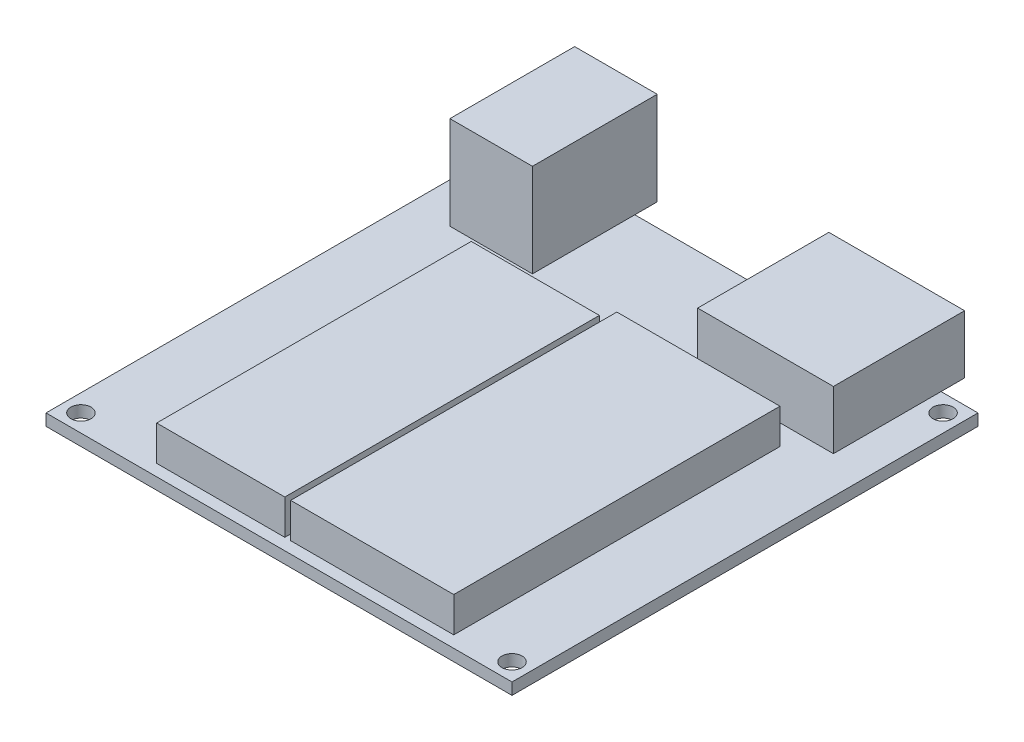
SolidWorks part; units mm, degrees
ref_plane "Front Plane" through (0, 0, 0) normal (0, 0, 1) x (1, 0, 0)
ref_plane "Top Plane" through (0, 0, 0) normal (0, 1, 0) x (1, 0, 0)
ref_plane "Right Plane" through (0, 0, 0) normal (1, 0, 0) x (0, 0, -1)
sketch "Sketch1" plane through (0, 0, 0) normal (0, 1, 0) x (1, 0, 0)
  line L0 (0, 0) -> (0, 50.8)
  line L1 (0, 50.8) -> (50.8, 50.8)
  line L2 (50.8, 50.8) -> (50.8, 0)
  line L3 (50.8, 0) -> (0, 0)
  line L4 (29.845, 40.64) -> (28.575, 40.64)
  line L5 (30.48, 43.18) -> (30.48, 38.1)
  line L6 (30.48, 38.1) -> (27.94, 38.1)
  line L7 (27.94, 38.1) -> (27.94, 43.18)
  line L8 (27.94, 43.18) -> (30.48, 43.18)
  line L9 (28.3382, 37.639) -> (28.245, 37.7322)
  line L10 (28.245, 37.7322) -> (28.0586, 37.7322)
  line L11 (28.0586, 37.7322) -> (27.9654, 37.639)
  line L12 (27.9654, 37.639) -> (27.9654, 37.2661)
  line L13 (27.9654, 37.2661) -> (28.0586, 37.1729)
  line L14 (28.0586, 37.1729) -> (28.245, 37.1729)
  line L15 (28.245, 37.1729) -> (28.3382, 37.2661)
  line L16 (28.5267, 37.5457) -> (28.7131, 37.7322)
  line L17 (28.7131, 37.7322) -> (28.7131, 37.1729)
  line L18 (28.5267, 37.1729) -> (28.8996, 37.1729)
  line L19 (28.2829, 43.8957) -> (28.4693, 44.0822)
  line L20 (28.4693, 44.0822) -> (28.4693, 43.5229)
  line L21 (28.2829, 43.5229) -> (28.6557, 43.5229)
  line L22 (28.8442, 43.6161) -> (28.8442, 43.989)
  line L23 (28.8442, 43.989) -> (28.9374, 44.0822)
  line L24 (28.9374, 44.0822) -> (29.1238, 44.0822)
  line L25 (29.1238, 44.0822) -> (29.2171, 43.989)
  line L26 (29.2171, 43.989) -> (29.2171, 43.6161)
  line L27 (29.2171, 43.6161) -> (29.1238, 43.5229)
  line L28 (29.1238, 43.5229) -> (28.9374, 43.5229)
  line L29 (28.9374, 43.5229) -> (28.8442, 43.6161)
  line L30 (28.8442, 43.6161) -> (29.2171, 43.989)
  line L31 (29.4055, 43.8957) -> (29.4055, 43.6161)
  line L32 (29.4055, 43.6161) -> (29.4987, 43.5229)
  line L33 (29.4987, 43.5229) -> (29.7784, 43.5229)
  line L34 (29.7784, 43.5229) -> (29.7784, 43.8957)
  line L35 (29.9668, 43.5229) -> (29.9668, 44.0822)
  line L36 (29.9668, 44.0822) -> (30.3397, 44.0822)
  line L37 (29.9668, 43.8025) -> (30.1533, 43.8025)
  line L38 (24.765, 40.64) -> (26.035, 40.64)
  line L39 (24.13, 38.1) -> (24.13, 43.18)
  line L40 (24.13, 43.18) -> (26.67, 43.18)
  line L41 (26.67, 43.18) -> (26.67, 38.1)
  line L42 (26.67, 38.1) -> (24.13, 38.1)
  line L43 (24.6756, 37.6644) -> (24.5824, 37.7576)
  line L44 (24.5824, 37.7576) -> (24.396, 37.7576)
  line L45 (24.396, 37.7576) -> (24.3028, 37.6644)
  line L46 (24.3028, 37.6644) -> (24.3028, 37.2915)
  line L47 (24.3028, 37.2915) -> (24.396, 37.1983)
  line L48 (24.396, 37.1983) -> (24.5824, 37.1983)
  line L49 (24.5824, 37.1983) -> (24.6756, 37.2915)
  line L50 (25.2369, 37.1983) -> (24.8641, 37.1983)
  line L51 (24.8641, 37.1983) -> (25.2369, 37.5711)
  line L52 (25.2369, 37.5711) -> (25.2369, 37.6644)
  line L53 (25.2369, 37.6644) -> (25.1437, 37.7576)
  line L54 (25.1437, 37.7576) -> (24.9573, 37.7576)
  line L55 (24.9573, 37.7576) -> (24.8641, 37.6644)
  line L56 (24.1326, 43.9211) -> (24.3191, 44.1076)
  line L57 (24.3191, 44.1076) -> (24.3191, 43.5483)
  line L58 (24.1326, 43.5483) -> (24.5055, 43.5483)
  line L59 (24.694, 43.6415) -> (24.694, 44.0144)
  line L60 (24.694, 44.0144) -> (24.7872, 44.1076)
  line L61 (24.7872, 44.1076) -> (24.9736, 44.1076)
  line L62 (24.9736, 44.1076) -> (25.0668, 44.0144)
  line L63 (25.0668, 44.0144) -> (25.0668, 43.6415)
  line L64 (25.0668, 43.6415) -> (24.9736, 43.5483)
  line L65 (24.9736, 43.5483) -> (24.7872, 43.5483)
  line L66 (24.7872, 43.5483) -> (24.694, 43.6415)
  line L67 (24.694, 43.6415) -> (25.0668, 44.0144)
  line L68 (25.2553, 43.9211) -> (25.2553, 43.6415)
  line L69 (25.2553, 43.6415) -> (25.3485, 43.5483)
  line L70 (25.3485, 43.5483) -> (25.6281, 43.5483)
  line L71 (25.6281, 43.5483) -> (25.6281, 43.9211)
  line L72 (25.8166, 43.5483) -> (25.8166, 44.1076)
  line L73 (25.8166, 44.1076) -> (26.1894, 44.1076)
  line L74 (25.8166, 43.8279) -> (26.003, 43.8279)
  line L75 (15.748, 34.29) -> (19.812, 34.29)
  line L76 (15.748, 34.29) -> (15.748, 31.75)
  line L77 (19.812, 31.75) -> (15.748, 31.75)
  line L78 (19.812, 31.75) -> (19.812, 34.29)
  line L79 (12.7, 33.02) -> (13.716, 33.02)
  line L80 (22.86, 33.02) -> (21.844, 33.02)
  line L81 (18.415, 33.02) -> (17.78, 33.02)
  line L82 (16.764, 32.385) -> (16.764, 33.655)
  line L83 (16.764, 33.655) -> (17.78, 33.02)
  line L84 (17.78, 33.02) -> (16.256, 33.02)
  line L85 (17.78, 33.02) -> (16.764, 32.385)
  line L86 (17.78, 32.385) -> (17.78, 33.02)
  line L87 (17.78, 33.02) -> (17.78, 33.655)
  line L88 (12.8591, 35.3702) -> (13.2404, 35.7515)
  line L89 (13.2404, 35.7515) -> (13.2404, 34.6075)
  line L90 (12.8591, 34.6075) -> (13.6217, 34.6075)
  line L91 (14.0285, 34.6075) -> (14.0285, 35.7515)
  line L92 (14.0285, 35.7515) -> (14.7912, 34.6075)
  line L93 (14.7912, 34.6075) -> (14.7912, 35.7515)
  line L94 (15.7699, 34.6075) -> (15.7699, 35.7515)
  line L95 (15.7699, 35.7515) -> (15.1979, 35.1795)
  line L96 (15.1979, 35.1795) -> (15.9605, 35.1795)
  line L97 (16.3673, 34.7982) -> (16.3673, 35.5608)
  line L98 (16.3673, 35.5608) -> (16.558, 35.7515)
  line L99 (16.558, 35.7515) -> (16.9393, 35.7515)
  line L100 (16.9393, 35.7515) -> (17.1299, 35.5608)
  line L101 (17.1299, 35.5608) -> (17.1299, 34.7982)
  line L102 (17.1299, 34.7982) -> (16.9393, 34.6075)
  line L103 (16.9393, 34.6075) -> (16.558, 34.6075)
  line L104 (16.558, 34.6075) -> (16.3673, 34.7982)
  line L105 (16.3673, 34.7982) -> (17.1299, 35.5608)
  line L106 (17.5367, 34.7982) -> (17.5367, 35.5608)
  line L107 (17.5367, 35.5608) -> (17.7273, 35.7515)
  line L108 (17.7273, 35.7515) -> (18.1087, 35.7515)
  line L109 (18.1087, 35.7515) -> (18.2993, 35.5608)
  line L110 (18.2993, 35.5608) -> (18.2993, 34.7982)
  line L111 (18.2993, 34.7982) -> (18.1087, 34.6075)
  line L112 (18.1087, 34.6075) -> (17.7273, 34.6075)
  line L113 (17.7273, 34.6075) -> (17.5367, 34.7982)
  line L114 (17.5367, 34.7982) -> (18.2993, 35.5608)
  line L115 (18.7061, 35.3702) -> (19.0874, 35.7515)
  line L116 (19.0874, 35.7515) -> (19.0874, 34.6075)
  line L117 (18.7061, 34.6075) -> (19.4687, 34.6075)
  line L118 (4.39, 39.64) -> (6.49, 39.64)
  line L119 (13.39, 50.34) -> (13.39, 53.24)
  line L120 (4.39, 53.24) -> (4.39, 50.34)
  line L121 (4.39, 53.24) -> (13.39, 53.24)
  line L122 (4.39, 50.34) -> (4.39, 45.04)
  line L123 (4.39, 39.64) -> (4.39, 40.34)
  line L124 (13.39, 50.34) -> (13.39, 39.64)
  line L125 (13.39, 39.64) -> (11.29, 39.64)
  line L126 (13.39, 50.34) -> (4.39, 50.34)
  line L127 (11.5901, 47.9299) -> (11.6536, 47.8663)
  line L128 (11.6536, 47.8663) -> (11.7172, 47.8663)
  line L129 (11.7172, 47.8663) -> (11.7807, 47.9299)
  line L130 (11.7807, 47.9299) -> (11.7807, 48.2476)
  line L131 (11.7172, 48.2476) -> (11.8443, 48.2476)
  line L132 (11.9643, 47.8663) -> (11.9643, 48.2476)
  line L133 (11.9643, 48.2476) -> (12.1549, 48.2476)
  line L134 (12.1549, 48.2476) -> (12.2185, 48.1841)
  line L135 (12.2185, 48.1841) -> (12.2185, 48.057)
  line L136 (12.2185, 48.057) -> (12.1549, 47.9934)
  line L137 (12.1549, 47.9934) -> (11.9643, 47.9934)
  line L138 (12.3385, 48.1205) -> (12.4656, 48.2476)
  line L139 (12.4656, 48.2476) -> (12.4656, 47.8663)
  line L140 (12.3385, 47.8663) -> (12.5927, 47.8663)
  line L141 (7.848, 49.1363) -> (7.848, 49.5176)
  line L142 (7.848, 49.5176) -> (8.0387, 49.5176)
  line L143 (8.0387, 49.5176) -> (8.1022, 49.4541)
  line L144 (8.1022, 49.4541) -> (8.1022, 49.327)
  line L145 (8.1022, 49.327) -> (8.0387, 49.2634)
  line L146 (8.0387, 49.2634) -> (7.848, 49.2634)
  line L147 (8.4129, 49.5176) -> (8.2858, 49.5176)
  line L148 (8.2858, 49.5176) -> (8.2222, 49.4541)
  line L149 (8.2222, 49.4541) -> (8.2222, 49.1999)
  line L150 (8.2222, 49.1999) -> (8.2858, 49.1363)
  line L151 (8.2858, 49.1363) -> (8.4129, 49.1363)
  line L152 (8.4129, 49.1363) -> (8.4764, 49.1999)
  line L153 (8.4764, 49.1999) -> (8.4764, 49.4541)
  line L154 (8.4764, 49.4541) -> (8.4129, 49.5176)
  line L155 (8.5964, 49.5176) -> (8.5964, 49.1363)
  line L156 (8.5964, 49.1363) -> (8.7235, 49.2634)
  line L157 (8.7235, 49.2634) -> (8.8506, 49.1363)
  line L158 (8.8506, 49.1363) -> (8.8506, 49.5176)
  line L159 (9.2248, 49.5176) -> (8.9706, 49.5176)
  line L160 (8.9706, 49.5176) -> (8.9706, 49.1363)
  line L161 (8.9706, 49.1363) -> (9.2248, 49.1363)
  line L162 (8.9706, 49.327) -> (9.0977, 49.327)
  line L163 (9.3448, 49.1363) -> (9.3448, 49.5176)
  line L164 (9.3448, 49.5176) -> (9.5355, 49.5176)
  line L165 (9.5355, 49.5176) -> (9.599, 49.4541)
  line L166 (9.599, 49.4541) -> (9.599, 49.327)
  line L167 (9.599, 49.327) -> (9.5355, 49.2634)
  line L168 (9.5355, 49.2634) -> (9.3448, 49.2634)
  line L169 (9.4719, 49.2634) -> (9.599, 49.1363)
  line L170 (9.719, 49.0727) -> (9.9733, 49.0727)
  line L171 (10.0932, 49.1999) -> (10.1568, 49.1363)
  line L172 (10.1568, 49.1363) -> (10.2204, 49.1363)
  line L173 (10.2204, 49.1363) -> (10.2839, 49.1999)
  line L174 (10.2839, 49.1999) -> (10.2839, 49.5176)
  line L175 (10.2204, 49.5176) -> (10.3475, 49.5176)
  line L176 (10.4674, 49.1363) -> (10.4674, 49.3905)
  line L177 (10.4674, 49.3905) -> (10.5945, 49.5176)
  line L178 (10.5945, 49.5176) -> (10.7217, 49.3905)
  line L179 (10.7217, 49.3905) -> (10.7217, 49.1363)
  line L180 (10.4674, 49.327) -> (10.7217, 49.327)
  line L181 (11.0959, 49.4541) -> (11.0323, 49.5176)
  line L182 (11.0323, 49.5176) -> (10.9052, 49.5176)
  line L183 (10.9052, 49.5176) -> (10.8417, 49.4541)
  line L184 (10.8417, 49.4541) -> (10.8417, 49.1999)
  line L185 (10.8417, 49.1999) -> (10.9052, 49.1363)
  line L186 (10.9052, 49.1363) -> (11.0323, 49.1363)
  line L187 (11.0323, 49.1363) -> (11.0959, 49.1999)
  line L188 (11.2159, 49.5176) -> (11.2159, 49.1363)
  line L189 (11.2159, 49.2634) -> (11.4701, 49.5176)
  line L190 (11.2794, 49.327) -> (11.4701, 49.1363)
  line L191 (11.5901, 49.1363) -> (11.5901, 49.5176)
  line L192 (11.5901, 49.5176) -> (11.7807, 49.5176)
  line L193 (11.7807, 49.5176) -> (11.8443, 49.4541)
  line L194 (11.8443, 49.4541) -> (11.8443, 49.327)
  line L195 (11.8443, 49.327) -> (11.7807, 49.2634)
  line L196 (11.7807, 49.2634) -> (11.5901, 49.2634)
  line L197 (12.0914, 49.1363) -> (12.0914, 49.5176)
  line L198 (11.9643, 49.5176) -> (12.2185, 49.5176)
  line L199 (12.3385, 49.1363) -> (12.3385, 49.5176)
  line L200 (12.3385, 49.327) -> (12.5927, 49.327)
  line L201 (12.5927, 49.5176) -> (12.5927, 49.1363)
  line L202 (10.795, 1.27) -> (24.765, 1.27)
  line L203 (24.765, 1.27) -> (24.765, 35.56)
  line L204 (24.765, 35.56) -> (10.795, 35.56)
  line L205 (10.795, 35.56) -> (10.795, 1.27)
  line L206 (14.1986, 3.8354) -> (13.6393, 3.8354)
  line L207 (13.6393, 3.8354) -> (13.6393, 4.115)
  line L208 (13.6393, 4.115) -> (13.7325, 4.2082)
  line L209 (13.7325, 4.2082) -> (13.919, 4.2082)
  line L210 (13.919, 4.2082) -> (14.0122, 4.115)
  line L211 (14.0122, 4.115) -> (14.0122, 3.8354)
  line L212 (14.0122, 4.0218) -> (14.1986, 4.2082)
  line L213 (13.6393, 4.3967) -> (14.1986, 4.7696)
  line L214 (13.6393, 4.7696) -> (14.1986, 4.3967)
  line L215 (16.7386, 4.0218) -> (16.1793, 4.0218)
  line L216 (16.1793, 3.8354) -> (16.1793, 4.2082)
  line L217 (16.1793, 4.3967) -> (16.7386, 4.7696)
  line L218 (16.1793, 4.7696) -> (16.7386, 4.3967)
  line L219 (18.8125, 4.2082) -> (18.7193, 4.115)
  line L220 (18.7193, 4.115) -> (18.7193, 3.9286)
  line L221 (18.7193, 3.9286) -> (18.8125, 3.8354)
  line L222 (18.8125, 3.8354) -> (19.1854, 3.8354)
  line L223 (19.1854, 3.8354) -> (19.2786, 3.9286)
  line L224 (19.2786, 3.9286) -> (19.2786, 4.115)
  line L225 (19.2786, 4.115) -> (19.1854, 4.2082)
  line L226 (19.1854, 4.2082) -> (18.999, 4.2082)
  line L227 (18.999, 4.2082) -> (18.999, 4.0218)
  line L228 (19.2786, 4.3967) -> (18.7193, 4.3967)
  line L229 (18.7193, 4.3967) -> (19.2786, 4.7696)
  line L230 (19.2786, 4.7696) -> (18.7193, 4.7696)
  line L231 (18.7193, 4.958) -> (19.2786, 4.958)
  line L232 (19.2786, 4.958) -> (19.2786, 5.2377)
  line L233 (19.2786, 5.2377) -> (19.1854, 5.3309)
  line L234 (19.1854, 5.3309) -> (18.8125, 5.3309)
  line L235 (18.8125, 5.3309) -> (18.7193, 5.2377)
  line L236 (18.7193, 5.2377) -> (18.7193, 4.958)
  line L237 (21.2593, 3.8354) -> (21.6322, 3.8354)
  line L238 (21.6322, 3.8354) -> (21.8186, 4.0218)
  line L239 (21.8186, 4.0218) -> (21.6322, 4.2082)
  line L240 (21.6322, 4.2082) -> (21.2593, 4.2082)
  line L241 (21.3525, 4.7696) -> (21.2593, 4.6763)
  line L242 (21.2593, 4.6763) -> (21.2593, 4.4899)
  line L243 (21.2593, 4.4899) -> (21.3525, 4.3967)
  line L244 (21.3525, 4.3967) -> (21.7254, 4.3967)
  line L245 (21.7254, 4.3967) -> (21.8186, 4.4899)
  line L246 (21.8186, 4.4899) -> (21.8186, 4.6763)
  line L247 (21.8186, 4.6763) -> (21.7254, 4.7696)
  line L248 (21.3525, 5.3309) -> (21.2593, 5.2377)
  line L249 (21.2593, 5.2377) -> (21.2593, 5.0512)
  line L250 (21.2593, 5.0512) -> (21.3525, 4.958)
  line L251 (21.3525, 4.958) -> (21.7254, 4.958)
  line L252 (21.7254, 4.958) -> (21.8186, 5.0512)
  line L253 (21.8186, 5.0512) -> (21.8186, 5.2377)
  line L254 (21.8186, 5.2377) -> (21.7254, 5.3309)
  line L255 (10.0752, 1.3335) -> (10.2235, 1.4818)
  line L256 (10.2235, 1.4818) -> (10.2235, 1.6301)
  line L257 (10.2235, 1.6301) -> (10.0752, 1.7784)
  line L258 (10.0752, 1.7784) -> (9.3337, 1.7784)
  line L259 (9.3337, 1.6301) -> (9.3337, 1.9267)
  line L260 (10.3718, 2.269) -> (10.3718, 2.8622)
  line L261 (10.2235, 3.2045) -> (9.3337, 3.2045)
  line L262 (9.3337, 3.2045) -> (9.3337, 3.6494)
  line L263 (9.3337, 3.6494) -> (9.482, 3.7977)
  line L264 (9.482, 3.7977) -> (9.6303, 3.7977)
  line L265 (9.6303, 3.7977) -> (9.7786, 3.6494)
  line L266 (9.7786, 3.6494) -> (9.9269, 3.7977)
  line L267 (9.9269, 3.7977) -> (10.0752, 3.7977)
  line L268 (10.0752, 3.7977) -> (10.2235, 3.6494)
  line L269 (10.2235, 3.6494) -> (10.2235, 3.2045)
  line L270 (9.7786, 3.2045) -> (9.7786, 3.6494)
  line L271 (10.2235, 4.4366) -> (9.3337, 4.4366)
  line L272 (9.3337, 4.14) -> (9.3337, 4.7332)
  line L273 (10.3718, 5.0756) -> (10.3718, 5.6687)
  line L274 (10.2235, 6.0111) -> (9.3337, 6.0111)
  line L275 (9.3337, 6.0111) -> (9.3337, 6.456)
  line L276 (9.3337, 6.456) -> (9.482, 6.6043)
  line L277 (9.482, 6.6043) -> (9.6303, 6.6043)
  line L278 (9.6303, 6.6043) -> (9.7786, 6.456)
  line L279 (9.7786, 6.456) -> (9.9269, 6.6043)
  line L280 (9.9269, 6.6043) -> (10.0752, 6.6043)
  line L281 (10.0752, 6.6043) -> (10.2235, 6.456)
  line L282 (10.2235, 6.456) -> (10.2235, 6.0111)
  line L283 (9.7786, 6.0111) -> (9.7786, 6.456)
  line L284 (9.3337, 7.3915) -> (9.3337, 7.0949)
  line L285 (9.3337, 7.0949) -> (9.482, 6.9466)
  line L286 (9.482, 6.9466) -> (10.0752, 6.9466)
  line L287 (10.0752, 6.9466) -> (10.2235, 7.0949)
  line L288 (10.2235, 7.0949) -> (10.2235, 7.3915)
  line L289 (10.2235, 7.3915) -> (10.0752, 7.5398)
  line L290 (10.0752, 7.5398) -> (9.482, 7.5398)
  line L291 (9.482, 7.5398) -> (9.3337, 7.3915)
  line L292 (10.2235, 7.8821) -> (9.6303, 7.8821)
  line L293 (9.6303, 7.8821) -> (9.3337, 8.1787)
  line L294 (9.3337, 8.1787) -> (9.6303, 8.4753)
  line L295 (9.6303, 8.4753) -> (10.2235, 8.4753)
  line L296 (9.7786, 7.8821) -> (9.7786, 8.4753)
  line L297 (10.2235, 8.8177) -> (9.3337, 8.8177)
  line L298 (9.3337, 8.8177) -> (9.3337, 9.2625)
  line L299 (9.3337, 9.2625) -> (9.482, 9.4108)
  line L300 (9.482, 9.4108) -> (9.7786, 9.4108)
  line L301 (9.7786, 9.4108) -> (9.9269, 9.2625)
  line L302 (9.9269, 9.2625) -> (9.9269, 8.8177)
  line L303 (9.9269, 9.1142) -> (10.2235, 9.4108)
  line L304 (9.3337, 9.7532) -> (10.2235, 9.7532)
  line L305 (10.2235, 9.7532) -> (10.2235, 10.198)
  line L306 (10.2235, 10.198) -> (10.0752, 10.3463)
  line L307 (10.0752, 10.3463) -> (9.482, 10.3463)
  line L308 (9.482, 10.3463) -> (9.3337, 10.198)
  line L309 (9.3337, 10.198) -> (9.3337, 9.7532)
  line L310 (10.3718, 10.6887) -> (10.3718, 11.2819)
  line L311 (9.6303, 11.6242) -> (9.3337, 11.9208)
  line L312 (9.3337, 11.9208) -> (10.2235, 11.9208)
  line L313 (10.2235, 11.6242) -> (10.2235, 12.2174)
  line L314 (3.81, 35.8648) -> (1.27, 35.8648)
  line L315 (0.9515, 36.2585) -> (2.0955, 36.2585)
  line L316 (2.0955, 36.2585) -> (2.0955, 37.0212)
  line L317 (0.9515, 38.1906) -> (0.9515, 37.4279)
  line L318 (0.9515, 37.4279) -> (2.0955, 37.4279)
  line L319 (2.0955, 37.4279) -> (2.0955, 38.1906)
  line L320 (1.5235, 37.4279) -> (1.5235, 37.8092)
  line L321 (0.9515, 38.5973) -> (2.0955, 38.5973)
  line L322 (2.0955, 38.5973) -> (2.0955, 39.1693)
  line L323 (2.0955, 39.1693) -> (1.9048, 39.3599)
  line L324 (1.9048, 39.3599) -> (1.1422, 39.3599)
  line L325 (1.1422, 39.3599) -> (0.9515, 39.1693)
  line L326 (0.9515, 39.1693) -> (0.9515, 38.5973)
  line L327 (1.3328, 39.7667) -> (0.9515, 40.148)
  line L328 (0.9515, 40.148) -> (2.0955, 40.148)
  line L329 (2.0955, 39.7667) -> (2.0955, 40.5293)
  line L330 (2.6768, 32.6898) -> (2.4032, 32.6898)
  line L331 (2.4032, 32.6898) -> (2.2098, 32.8832)
  line L332 (2.2098, 32.8832) -> (2.2098, 33.1568)
  line L333 (2.2098, 33.1568) -> (2.4032, 33.3502)
  line L334 (2.4032, 33.3502) -> (2.6768, 33.3502)
  line L335 (2.6768, 33.3502) -> (2.8702, 33.1568)
  line L336 (2.8702, 33.1568) -> (2.8702, 32.8832)
  line L337 (2.8702, 32.8832) -> (2.6768, 32.6898)
  line L338 (2.6768, 32.6898) -> (2.4032, 32.6898)
  line L339 (2.6768, 32.6898) -> (2.4032, 32.6898)
  line L340 (2.4032, 32.6898) -> (2.2098, 32.8832)
  line L341 (2.2098, 32.8832) -> (2.2098, 33.1568)
  line L342 (2.2098, 33.1568) -> (2.4032, 33.3502)
  line L343 (2.4032, 33.3502) -> (2.6768, 33.3502)
  line L344 (2.6768, 33.3502) -> (2.8702, 33.1568)
  line L345 (2.8702, 33.1568) -> (2.8702, 32.8832)
  line L346 (2.8702, 32.8832) -> (2.6768, 32.6898)
  line L347 (2.6768, 32.6898) -> (2.4032, 32.6898)
  line L348 (2.6768, 35.2298) -> (2.4032, 35.2298)
  line L349 (2.4032, 35.2298) -> (2.2098, 35.4232)
  line L350 (2.2098, 35.4232) -> (2.2098, 35.6968)
  line L351 (2.2098, 35.6968) -> (2.4032, 35.8902)
  line L352 (2.4032, 35.8902) -> (2.6768, 35.8902)
  line L353 (2.6768, 35.8902) -> (2.8702, 35.6968)
  line L354 (2.8702, 35.6968) -> (2.8702, 35.4232)
  line L355 (2.8702, 35.4232) -> (2.6768, 35.2298)
  line L356 (2.6768, 35.2298) -> (2.4032, 35.2298)
  line L357 (2.6768, 35.2298) -> (2.4032, 35.2298)
  line L358 (2.4032, 35.2298) -> (2.2098, 35.4232)
  line L359 (2.2098, 35.4232) -> (2.2098, 35.6968)
  line L360 (2.2098, 35.6968) -> (2.4032, 35.8902)
  line L361 (2.4032, 35.8902) -> (2.6768, 35.8902)
  line L362 (2.6768, 35.8902) -> (2.8702, 35.6968)
  line L363 (2.8702, 35.6968) -> (2.8702, 35.4232)
  line L364 (2.8702, 35.4232) -> (2.6768, 35.2298)
  line L365 (2.6768, 35.2298) -> (2.4032, 35.2298)
  line L366 (10.16, 36.83) -> (10.16, 31.75)
  line L367 (10.16, 31.75) -> (5.08, 31.75)
  line L368 (5.08, 31.75) -> (5.08, 36.83)
  line L369 (5.08, 36.83) -> (10.16, 36.83)
  line L370 (8.9275, 32.8596) -> (8.9275, 32.6139)
  line L371 (8.9275, 32.6139) -> (9.0504, 32.491)
  line L372 (9.0504, 32.491) -> (9.5418, 32.491)
  line L373 (9.5418, 32.491) -> (9.6647, 32.6139)
  line L374 (9.6647, 32.6139) -> (9.6647, 32.8596)
  line L375 (9.6647, 32.8596) -> (9.5418, 32.9825)
  line L376 (9.5418, 32.9825) -> (9.0504, 32.9825)
  line L377 (9.0504, 32.9825) -> (8.9275, 32.8596)
  line L378 (9.6647, 33.2394) -> (8.9275, 33.2394)
  line L379 (8.9275, 33.2394) -> (9.6647, 33.7309)
  line L380 (9.6647, 33.7309) -> (8.9275, 33.7309)
  line L381 (8.9275, 34.3565) -> (8.9275, 34.1107)
  line L382 (8.9275, 34.1107) -> (9.0504, 33.9878)
  line L383 (9.0504, 33.9878) -> (9.5418, 33.9878)
  line L384 (9.5418, 33.9878) -> (9.6647, 34.1107)
  line L385 (9.6647, 34.1107) -> (9.6647, 34.3565)
  line L386 (9.6647, 34.3565) -> (9.5418, 34.4793)
  line L387 (9.5418, 34.4793) -> (9.0504, 34.4793)
  line L388 (9.0504, 34.4793) -> (8.9275, 34.3565)
  line L389 (9.6647, 34.7363) -> (8.9275, 34.7363)
  line L390 (8.9275, 34.7363) -> (8.9275, 35.2277)
  line L391 (9.2961, 34.7363) -> (9.2961, 34.982)
  line L392 (9.6647, 35.4847) -> (8.9275, 35.4847)
  line L393 (8.9275, 35.4847) -> (8.9275, 35.9762)
  line L394 (9.2961, 35.4847) -> (9.2961, 35.7304)
  line L395 (5.7525, 31.7426) -> (6.4897, 31.7426)
  line L396 (6.4897, 31.7426) -> (6.4897, 32.1112)
  line L397 (6.4897, 32.1112) -> (6.3668, 32.2341)
  line L398 (6.3668, 32.2341) -> (5.8754, 32.2341)
  line L399 (5.8754, 32.2341) -> (5.7525, 32.1112)
  line L400 (5.7525, 32.1112) -> (5.7525, 31.7426)
  line L401 (5.8754, 32.9825) -> (5.7525, 32.8596)
  line L402 (5.7525, 32.8596) -> (5.7525, 32.6139)
  line L403 (5.7525, 32.6139) -> (5.8754, 32.491)
  line L404 (5.8754, 32.491) -> (5.9982, 32.491)
  line L405 (5.9982, 32.491) -> (6.1211, 32.6139)
  line L406 (6.1211, 32.6139) -> (6.1211, 32.8596)
  line L407 (6.1211, 32.8596) -> (6.244, 32.9825)
  line L408 (6.244, 32.9825) -> (6.3668, 32.9825)
  line L409 (6.3668, 32.9825) -> (6.4897, 32.8596)
  line L410 (6.4897, 32.8596) -> (6.4897, 32.6139)
  line L411 (6.4897, 32.6139) -> (6.3668, 32.491)
  line L412 (6.1211, 33.2394) -> (6.1211, 33.7309)
  line L413 (6.4897, 34.4793) -> (6.4897, 33.9878)
  line L414 (6.4897, 33.9878) -> (5.9982, 34.4793)
  line L415 (5.9982, 34.4793) -> (5.8754, 34.4793)
  line L416 (5.8754, 34.4793) -> (5.7525, 34.3565)
  line L417 (5.7525, 34.3565) -> (5.7525, 34.1107)
  line L418 (5.7525, 34.1107) -> (5.8754, 33.9878)
  line L419 (6.4897, 35.2277) -> (6.4897, 34.7363)
  line L420 (6.4897, 34.7363) -> (5.9982, 35.2277)
  line L421 (5.9982, 35.2277) -> (5.8754, 35.2277)
  line L422 (5.8754, 35.2277) -> (5.7525, 35.1049)
  line L423 (5.7525, 35.1049) -> (5.7525, 34.8591)
  line L424 (5.7525, 34.8591) -> (5.8754, 34.7363)
  line L425 (5.8754, 35.4847) -> (5.7525, 35.6075)
  line L426 (5.7525, 35.6075) -> (5.7525, 35.8533)
  line L427 (5.7525, 35.8533) -> (5.8754, 35.9762)
  line L428 (5.8754, 35.9762) -> (5.9982, 35.9762)
  line L429 (5.9982, 35.9762) -> (6.1211, 35.8533)
  line L430 (6.1211, 35.8533) -> (6.244, 35.9762)
  line L431 (6.244, 35.9762) -> (6.3668, 35.9762)
  line L432 (6.3668, 35.9762) -> (6.4897, 35.8533)
  line L433 (6.4897, 35.8533) -> (6.4897, 35.6075)
  line L434 (6.4897, 35.6075) -> (6.3668, 35.4847)
  line L435 (6.3668, 35.4847) -> (6.244, 35.4847)
  line L436 (6.244, 35.4847) -> (6.1211, 35.6075)
  line L437 (6.1211, 35.6075) -> (5.9982, 35.4847)
  line L438 (5.9982, 35.4847) -> (5.8754, 35.4847)
  line L439 (6.1211, 35.6075) -> (6.1211, 35.8533)
  line L440 (15.24, 21.082) -> (20.32, 21.082)
  line L441 (20.32, 21.082) -> (20.32, 20.32)
  line L442 (20.32, 20.32) -> (20.32, 19.558)
  line L443 (20.32, 19.558) -> (15.24, 19.558)
  line L444 (15.24, 19.558) -> (15.24, 20.32)
  line L445 (15.24, 20.32) -> (15.24, 21.082)
  line L446 (20.32, 20.32) -> (20.574, 20.32)
  line L447 (15.24, 20.32) -> (14.986, 20.32)
  line L448 (15.2527, 21.6027) -> (15.2527, 21.984)
  line L449 (15.2527, 21.984) -> (15.4434, 21.984)
  line L450 (15.4434, 21.984) -> (15.5069, 21.9205)
  line L451 (15.5069, 21.9205) -> (15.5069, 21.7934)
  line L452 (15.5069, 21.7934) -> (15.4434, 21.7298)
  line L453 (15.4434, 21.7298) -> (15.2527, 21.7298)
  line L454 (15.3798, 21.7298) -> (15.5069, 21.6027)
  line L455 (15.6269, 21.8569) -> (15.754, 21.984)
  line L456 (15.754, 21.984) -> (15.754, 21.6027)
  line L457 (15.6269, 21.6027) -> (15.8811, 21.6027)
  line L458 (15.8242, 20.5914) -> (16.1123, 20.8795)
  line L459 (16.1123, 20.8795) -> (16.1123, 20.0152)
  line L460 (15.8242, 20.0152) -> (16.4004, 20.0152)
  line L461 (16.7597, 20.1593) -> (16.7597, 20.7355)
  line L462 (16.7597, 20.7355) -> (16.9038, 20.8795)
  line L463 (16.9038, 20.8795) -> (17.1919, 20.8795)
  line L464 (17.1919, 20.8795) -> (17.3359, 20.7355)
  line L465 (17.3359, 20.7355) -> (17.3359, 20.1593)
  line L466 (17.3359, 20.1593) -> (17.1919, 20.0152)
  line L467 (17.1919, 20.0152) -> (16.9038, 20.0152)
  line L468 (16.9038, 20.0152) -> (16.7597, 20.1593)
  line L469 (16.7597, 20.1593) -> (17.3359, 20.7355)
  line L470 (17.6952, 20.8795) -> (17.6952, 20.0152)
  line L471 (17.6952, 20.3033) -> (18.2715, 20.8795)
  line L472 (17.8393, 20.4474) -> (18.2715, 20.0152)
  line L473 (15.24, 18.542) -> (20.32, 18.542)
  line L474 (20.32, 18.542) -> (20.32, 17.78)
  line L475 (20.32, 17.78) -> (20.32, 17.018)
  line L476 (20.32, 17.018) -> (15.24, 17.018)
  line L477 (15.24, 17.018) -> (15.24, 17.78)
  line L478 (15.24, 17.78) -> (15.24, 18.542)
  line L479 (20.32, 17.78) -> (20.574, 17.78)
  line L480 (15.24, 17.78) -> (14.986, 17.78)
  line L481 (15.2527, 19.0627) -> (15.2527, 19.444)
  line L482 (15.2527, 19.444) -> (15.4434, 19.444)
  line L483 (15.4434, 19.444) -> (15.5069, 19.3805)
  line L484 (15.5069, 19.3805) -> (15.5069, 19.2534)
  line L485 (15.5069, 19.2534) -> (15.4434, 19.1898)
  line L486 (15.4434, 19.1898) -> (15.2527, 19.1898)
  line L487 (15.3798, 19.1898) -> (15.5069, 19.0627)
  line L488 (15.8811, 19.0627) -> (15.6269, 19.0627)
  line L489 (15.6269, 19.0627) -> (15.8811, 19.3169)
  line L490 (15.8811, 19.3169) -> (15.8811, 19.3805)
  line L491 (15.8811, 19.3805) -> (15.8176, 19.444)
  line L492 (15.8176, 19.444) -> (15.6905, 19.444)
  line L493 (15.6905, 19.444) -> (15.6269, 19.3805)
  line L494 (15.8242, 18.0514) -> (16.1123, 18.3395)
  line L495 (16.1123, 18.3395) -> (16.1123, 17.4752)
  line L496 (15.8242, 17.4752) -> (16.4004, 17.4752)
  line L497 (16.7597, 17.6193) -> (16.7597, 18.1955)
  line L498 (16.7597, 18.1955) -> (16.9038, 18.3395)
  line L499 (16.9038, 18.3395) -> (17.1919, 18.3395)
  line L500 (17.1919, 18.3395) -> (17.3359, 18.1955)
  line L501 (17.3359, 18.1955) -> (17.3359, 17.6193)
  line L502 (17.3359, 17.6193) -> (17.1919, 17.4752)
  line L503 (17.1919, 17.4752) -> (16.9038, 17.4752)
  line L504 (16.9038, 17.4752) -> (16.7597, 17.6193)
  line L505 (16.7597, 17.6193) -> (17.3359, 18.1955)
  line L506 (17.6952, 18.3395) -> (17.6952, 17.4752)
  line L507 (17.6952, 17.7633) -> (18.2715, 18.3395)
  line L508 (17.8393, 17.9074) -> (18.2715, 17.4752)
  line L509 (15.24, 16.002) -> (20.32, 16.002)
  line L510 (20.32, 16.002) -> (20.32, 15.24)
  line L511 (20.32, 15.24) -> (20.32, 14.478)
  line L512 (20.32, 14.478) -> (15.24, 14.478)
  line L513 (15.24, 14.478) -> (15.24, 15.24)
  line L514 (15.24, 15.24) -> (15.24, 16.002)
  line L515 (20.32, 15.24) -> (20.574, 15.24)
  line L516 (15.24, 15.24) -> (14.986, 15.24)
  line L517 (15.2527, 16.5227) -> (15.2527, 16.904)
  line L518 (15.2527, 16.904) -> (15.4434, 16.904)
  line L519 (15.4434, 16.904) -> (15.5069, 16.8405)
  line L520 (15.5069, 16.8405) -> (15.5069, 16.7134)
  line L521 (15.5069, 16.7134) -> (15.4434, 16.6498)
  line L522 (15.4434, 16.6498) -> (15.2527, 16.6498)
  line L523 (15.3798, 16.6498) -> (15.5069, 16.5227)
  line L524 (15.6269, 16.8405) -> (15.6905, 16.904)
  line L525 (15.6905, 16.904) -> (15.8176, 16.904)
  line L526 (15.8176, 16.904) -> (15.8811, 16.8405)
  line L527 (15.8811, 16.8405) -> (15.8811, 16.7769)
  line L528 (15.8811, 16.7769) -> (15.8176, 16.7134)
  line L529 (15.8176, 16.7134) -> (15.754, 16.7134)
  line L530 (15.8176, 16.7134) -> (15.8811, 16.6498)
  line L531 (15.8811, 16.6498) -> (15.8811, 16.5863)
  line L532 (15.8811, 16.5863) -> (15.8176, 16.5227)
  line L533 (15.8176, 16.5227) -> (15.6905, 16.5227)
  line L534 (15.6905, 16.5227) -> (15.6269, 16.5863)
  line L535 (15.8242, 15.5114) -> (16.1123, 15.7995)
  line L536 (16.1123, 15.7995) -> (16.1123, 14.9352)
  line L537 (15.8242, 14.9352) -> (16.4004, 14.9352)
  line L538 (16.7597, 15.0793) -> (16.7597, 15.6555)
  line L539 (16.7597, 15.6555) -> (16.9038, 15.7995)
  line L540 (16.9038, 15.7995) -> (17.1919, 15.7995)
  line L541 (17.1919, 15.7995) -> (17.3359, 15.6555)
  line L542 (17.3359, 15.6555) -> (17.3359, 15.0793)
  line L543 (17.3359, 15.0793) -> (17.1919, 14.9352)
  line L544 (17.1919, 14.9352) -> (16.9038, 14.9352)
  line L545 (16.9038, 14.9352) -> (16.7597, 15.0793)
  line L546 (16.7597, 15.0793) -> (17.3359, 15.6555)
  line L547 (17.6952, 15.7995) -> (17.6952, 14.9352)
  line L548 (17.6952, 15.2233) -> (18.2715, 15.7995)
  line L549 (17.8393, 15.3674) -> (18.2715, 14.9352)
  line L550 (15.24, 13.462) -> (20.32, 13.462)
  line L551 (20.32, 13.462) -> (20.32, 12.7)
  line L552 (20.32, 12.7) -> (20.32, 11.938)
  line L553 (20.32, 11.938) -> (15.24, 11.938)
  line L554 (15.24, 11.938) -> (15.24, 12.7)
  line L555 (15.24, 12.7) -> (15.24, 13.462)
  line L556 (20.32, 12.7) -> (20.574, 12.7)
  line L557 (15.24, 12.7) -> (14.986, 12.7)
  line L558 (15.2527, 13.9827) -> (15.2527, 14.364)
  line L559 (15.2527, 14.364) -> (15.4434, 14.364)
  line L560 (15.4434, 14.364) -> (15.5069, 14.3005)
  line L561 (15.5069, 14.3005) -> (15.5069, 14.1734)
  line L562 (15.5069, 14.1734) -> (15.4434, 14.1098)
  line L563 (15.4434, 14.1098) -> (15.2527, 14.1098)
  line L564 (15.3798, 14.1098) -> (15.5069, 13.9827)
  line L565 (15.8176, 13.9827) -> (15.8176, 14.364)
  line L566 (15.8176, 14.364) -> (15.6269, 14.1734)
  line L567 (15.6269, 14.1734) -> (15.8811, 14.1734)
  line L568 (15.8242, 12.9714) -> (16.1123, 13.2595)
  line L569 (16.1123, 13.2595) -> (16.1123, 12.3952)
  line L570 (15.8242, 12.3952) -> (16.4004, 12.3952)
  line L571 (16.7597, 12.5393) -> (16.7597, 13.1155)
  line L572 (16.7597, 13.1155) -> (16.9038, 13.2595)
  line L573 (16.9038, 13.2595) -> (17.1919, 13.2595)
  line L574 (17.1919, 13.2595) -> (17.3359, 13.1155)
  line L575 (17.3359, 13.1155) -> (17.3359, 12.5393)
  line L576 (17.3359, 12.5393) -> (17.1919, 12.3952)
  line L577 (17.1919, 12.3952) -> (16.9038, 12.3952)
  line L578 (16.9038, 12.3952) -> (16.7597, 12.5393)
  line L579 (16.7597, 12.5393) -> (17.3359, 13.1155)
  line L580 (17.6952, 13.2595) -> (17.6952, 12.3952)
  line L581 (17.6952, 12.6833) -> (18.2715, 13.2595)
  line L582 (17.8393, 12.8274) -> (18.2715, 12.3952)
  line L583 (15.24, 10.922) -> (20.32, 10.922)
  line L584 (20.32, 10.922) -> (20.32, 10.16)
  line L585 (20.32, 10.16) -> (20.32, 9.398)
  line L586 (20.32, 9.398) -> (15.24, 9.398)
  line L587 (15.24, 9.398) -> (15.24, 10.16)
  line L588 (15.24, 10.16) -> (15.24, 10.922)
  line L589 (20.32, 10.16) -> (20.574, 10.16)
  line L590 (15.24, 10.16) -> (14.986, 10.16)
  line L591 (15.2527, 11.4427) -> (15.2527, 11.824)
  line L592 (15.2527, 11.824) -> (15.4434, 11.824)
  line L593 (15.4434, 11.824) -> (15.5069, 11.7605)
  line L594 (15.5069, 11.7605) -> (15.5069, 11.6334)
  line L595 (15.5069, 11.6334) -> (15.4434, 11.5698)
  line L596 (15.4434, 11.5698) -> (15.2527, 11.5698)
  line L597 (15.3798, 11.5698) -> (15.5069, 11.4427)
  line L598 (15.8811, 11.824) -> (15.6269, 11.824)
  line L599 (15.6269, 11.824) -> (15.6269, 11.6334)
  line L600 (15.6269, 11.6334) -> (15.754, 11.6969)
  line L601 (15.754, 11.6969) -> (15.8176, 11.6969)
  line L602 (15.8176, 11.6969) -> (15.8811, 11.6334)
  line L603 (15.8811, 11.6334) -> (15.8811, 11.5063)
  line L604 (15.8811, 11.5063) -> (15.8176, 11.4427)
  line L605 (15.8176, 11.4427) -> (15.6905, 11.4427)
  line L606 (15.6905, 11.4427) -> (15.6269, 11.5063)
  line L607 (15.8242, 10.4314) -> (16.1123, 10.7195)
  line L608 (16.1123, 10.7195) -> (16.1123, 9.8552)
  line L609 (15.8242, 9.8552) -> (16.4004, 9.8552)
  line L610 (16.7597, 9.9993) -> (16.7597, 10.5755)
  line L611 (16.7597, 10.5755) -> (16.9038, 10.7195)
  line L612 (16.9038, 10.7195) -> (17.1919, 10.7195)
  line L613 (17.1919, 10.7195) -> (17.3359, 10.5755)
  line L614 (17.3359, 10.5755) -> (17.3359, 9.9993)
  line L615 (17.3359, 9.9993) -> (17.1919, 9.8552)
  line L616 (17.1919, 9.8552) -> (16.9038, 9.8552)
  line L617 (16.9038, 9.8552) -> (16.7597, 9.9993)
  line L618 (16.7597, 9.9993) -> (17.3359, 10.5755)
  line L619 (17.6952, 10.7195) -> (17.6952, 9.8552)
  line L620 (17.6952, 10.1433) -> (18.2715, 10.7195)
  line L621 (17.8393, 10.2874) -> (18.2715, 9.8552)
  line L622 (15.24, 8.382) -> (20.32, 8.382)
  line L623 (20.32, 8.382) -> (20.32, 7.62)
  line L624 (20.32, 7.62) -> (20.32, 6.858)
  line L625 (20.32, 6.858) -> (15.24, 6.858)
  line L626 (15.24, 6.858) -> (15.24, 7.62)
  line L627 (15.24, 7.62) -> (15.24, 8.382)
  line L628 (20.32, 7.62) -> (20.574, 7.62)
  line L629 (15.24, 7.62) -> (14.986, 7.62)
  line L630 (15.2527, 8.9027) -> (15.2527, 9.284)
  line L631 (15.2527, 9.284) -> (15.4434, 9.284)
  line L632 (15.4434, 9.284) -> (15.5069, 9.2205)
  line L633 (15.5069, 9.2205) -> (15.5069, 9.0934)
  line L634 (15.5069, 9.0934) -> (15.4434, 9.0298)
  line L635 (15.4434, 9.0298) -> (15.2527, 9.0298)
  line L636 (15.3798, 9.0298) -> (15.5069, 8.9027)
  line L637 (15.8811, 9.284) -> (15.754, 9.2205)
  line L638 (15.754, 9.2205) -> (15.6269, 9.0934)
  line L639 (15.6269, 9.0934) -> (15.6269, 8.9663)
  line L640 (15.6269, 8.9663) -> (15.6905, 8.9027)
  line L641 (15.6905, 8.9027) -> (15.8176, 8.9027)
  line L642 (15.8176, 8.9027) -> (15.8811, 8.9663)
  line L643 (15.8811, 8.9663) -> (15.8811, 9.0298)
  line L644 (15.8811, 9.0298) -> (15.8176, 9.0934)
  line L645 (15.8176, 9.0934) -> (15.6269, 9.0934)
  line L646 (15.8242, 7.8914) -> (16.1123, 8.1795)
  line L647 (16.1123, 8.1795) -> (16.1123, 7.3152)
  line L648 (15.8242, 7.3152) -> (16.4004, 7.3152)
  line L649 (16.7597, 7.4593) -> (16.7597, 8.0355)
  line L650 (16.7597, 8.0355) -> (16.9038, 8.1795)
  line L651 (16.9038, 8.1795) -> (17.1919, 8.1795)
  line L652 (17.1919, 8.1795) -> (17.3359, 8.0355)
  line L653 (17.3359, 8.0355) -> (17.3359, 7.4593)
  line L654 (17.3359, 7.4593) -> (17.1919, 7.3152)
  line L655 (17.1919, 7.3152) -> (16.9038, 7.3152)
  line L656 (16.9038, 7.3152) -> (16.7597, 7.4593)
  line L657 (16.7597, 7.4593) -> (17.3359, 8.0355)
  line L658 (17.6952, 8.1795) -> (17.6952, 7.3152)
  line L659 (17.6952, 7.6033) -> (18.2715, 8.1795)
  line L660 (17.8393, 7.7474) -> (18.2715, 7.3152)
  line L661 (15.24, 28.702) -> (20.32, 28.702)
  line L662 (20.32, 28.702) -> (20.32, 27.94)
  line L663 (20.32, 27.94) -> (20.32, 27.178)
  line L664 (20.32, 27.178) -> (15.24, 27.178)
  line L665 (15.24, 27.178) -> (15.24, 27.94)
  line L666 (15.24, 27.94) -> (15.24, 28.702)
  line L667 (20.32, 27.94) -> (20.574, 27.94)
  line L668 (15.24, 27.94) -> (14.986, 27.94)
  line L669 (15.2527, 29.2227) -> (15.2527, 29.604)
  line L670 (15.2527, 29.604) -> (15.4434, 29.604)
  line L671 (15.4434, 29.604) -> (15.5069, 29.5405)
  line L672 (15.5069, 29.5405) -> (15.5069, 29.4134)
  line L673 (15.5069, 29.4134) -> (15.4434, 29.3498)
  line L674 (15.4434, 29.3498) -> (15.2527, 29.3498)
  line L675 (15.3798, 29.3498) -> (15.5069, 29.2227)
  line L676 (15.6269, 29.604) -> (15.8811, 29.604)
  line L677 (15.8811, 29.604) -> (15.8811, 29.5405)
  line L678 (15.8811, 29.5405) -> (15.6269, 29.2863)
  line L679 (15.6269, 29.2863) -> (15.6269, 29.2227)
  line L680 (15.8242, 28.2114) -> (16.1123, 28.4995)
  line L681 (16.1123, 28.4995) -> (16.1123, 27.6352)
  line L682 (15.8242, 27.6352) -> (16.4004, 27.6352)
  line L683 (16.7597, 27.6352) -> (16.7597, 27.7793)
  line L684 (16.7597, 27.7793) -> (16.9038, 27.7793)
  line L685 (16.9038, 27.7793) -> (16.9038, 27.6352)
  line L686 (16.9038, 27.6352) -> (16.7597, 27.6352)
  line L687 (17.2275, 28.2114) -> (17.5156, 28.4995)
  line L688 (17.5156, 28.4995) -> (17.5156, 27.6352)
  line L689 (17.2275, 27.6352) -> (17.8037, 27.6352)
  line L690 (18.163, 28.4995) -> (18.163, 27.6352)
  line L691 (18.163, 27.9233) -> (18.7392, 28.4995)
  line L692 (18.307, 28.0674) -> (18.7392, 27.6352)
  line L693 (25.4, 49.53) -> (30.48, 49.53)
  line L694 (30.48, 49.53) -> (30.48, 44.45)
  line L695 (30.48, 44.45) -> (25.4, 44.45)
  line L696 (25.4, 44.45) -> (25.4, 49.53)
  line L697 (26.0731, 48.2981) -> (26.0731, 49.0353)
  line L698 (26.0731, 49.0353) -> (26.4417, 49.0353)
  line L699 (26.4417, 49.0353) -> (26.5646, 48.9124)
  line L700 (26.5646, 48.9124) -> (26.5646, 48.6667)
  line L701 (26.5646, 48.6667) -> (26.4417, 48.5438)
  line L702 (26.4417, 48.5438) -> (26.0731, 48.5438)
  line L703 (26.3188, 48.5438) -> (26.5646, 48.2981)
  line L704 (27.313, 49.0353) -> (26.8215, 49.0353)
  line L705 (26.8215, 49.0353) -> (26.8215, 48.2981)
  line L706 (26.8215, 48.2981) -> (27.313, 48.2981)
  line L707 (26.8215, 48.6667) -> (27.0673, 48.6667)
  line L708 (28.0614, 48.9124) -> (27.9386, 49.0353)
  line L709 (27.9386, 49.0353) -> (27.6928, 49.0353)
  line L710 (27.6928, 49.0353) -> (27.5699, 48.9124)
  line L711 (27.5699, 48.9124) -> (27.5699, 48.7896)
  line L712 (27.5699, 48.7896) -> (27.6928, 48.6667)
  line L713 (27.6928, 48.6667) -> (27.9386, 48.6667)
  line L714 (27.9386, 48.6667) -> (28.0614, 48.5438)
  line L715 (28.0614, 48.5438) -> (28.0614, 48.421)
  line L716 (28.0614, 48.421) -> (27.9386, 48.2981)
  line L717 (27.9386, 48.2981) -> (27.6928, 48.2981)
  line L718 (27.6928, 48.2981) -> (27.5699, 48.421)
  line L719 (28.8098, 49.0353) -> (28.3184, 49.0353)
  line L720 (28.3184, 49.0353) -> (28.3184, 48.2981)
  line L721 (28.3184, 48.2981) -> (28.8098, 48.2981)
  line L722 (28.3184, 48.6667) -> (28.5641, 48.6667)
  line L723 (29.3125, 48.2981) -> (29.3125, 49.0353)
  line L724 (29.0668, 49.0353) -> (29.5583, 49.0353)
  line L725 (26.0731, 45.8603) -> (26.0731, 45.1231)
  line L726 (26.0731, 45.1231) -> (26.4417, 45.1231)
  line L727 (26.4417, 45.1231) -> (26.5646, 45.246)
  line L728 (26.5646, 45.246) -> (26.5646, 45.7374)
  line L729 (26.5646, 45.7374) -> (26.4417, 45.8603)
  line L730 (26.4417, 45.8603) -> (26.0731, 45.8603)
  line L731 (27.313, 45.7374) -> (27.1901, 45.8603)
  line L732 (27.1901, 45.8603) -> (26.9444, 45.8603)
  line L733 (26.9444, 45.8603) -> (26.8215, 45.7374)
  line L734 (26.8215, 45.7374) -> (26.8215, 45.6146)
  line L735 (26.8215, 45.6146) -> (26.9444, 45.4917)
  line L736 (26.9444, 45.4917) -> (27.1901, 45.4917)
  line L737 (27.1901, 45.4917) -> (27.313, 45.3688)
  line L738 (27.313, 45.3688) -> (27.313, 45.246)
  line L739 (27.313, 45.246) -> (27.1901, 45.1231)
  line L740 (27.1901, 45.1231) -> (26.9444, 45.1231)
  line L741 (26.9444, 45.1231) -> (26.8215, 45.246)
  line L742 (27.5699, 45.4917) -> (28.0614, 45.4917)
  line L743 (28.8098, 45.1231) -> (28.3184, 45.1231)
  line L744 (28.3184, 45.1231) -> (28.8098, 45.6146)
  line L745 (28.8098, 45.6146) -> (28.8098, 45.7374)
  line L746 (28.8098, 45.7374) -> (28.687, 45.8603)
  line L747 (28.687, 45.8603) -> (28.4412, 45.8603)
  line L748 (28.4412, 45.8603) -> (28.3184, 45.7374)
  line L749 (29.5583, 45.1231) -> (29.0668, 45.1231)
  line L750 (29.0668, 45.1231) -> (29.5583, 45.6146)
  line L751 (29.5583, 45.6146) -> (29.5583, 45.7374)
  line L752 (29.5583, 45.7374) -> (29.4354, 45.8603)
  line L753 (29.4354, 45.8603) -> (29.1896, 45.8603)
  line L754 (29.1896, 45.8603) -> (29.0668, 45.7374)
  line L755 (29.8152, 45.8603) -> (30.3067, 45.8603)
  line L756 (30.3067, 45.8603) -> (30.3067, 45.7374)
  line L757 (30.3067, 45.7374) -> (29.8152, 45.246)
  line L758 (29.8152, 45.246) -> (29.8152, 45.1231)
  line L759 (6.35, 20.32) -> (6.35, 30.48)
  line L760 (6.35, 30.48) -> (-5.08, 30.48)
  line L761 (-5.08, 30.48) -> (-5.08, 20.32)
  line L762 (-5.08, 20.32) -> (6.35, 20.32)
  line L763 (6.35, 20.32) -> (6.35, 30.48)
  line L764 (6.223, 20.32) -> (6.223, 30.48)
  line L765 (6.096, 20.32) -> (6.096, 30.48)
  line L766 (5.969, 20.32) -> (5.969, 30.48)
  line L767 (5.842, 20.32) -> (5.842, 30.48)
  line L768 (5.715, 20.32) -> (5.715, 30.48)
  line L769 (5.588, 20.32) -> (5.588, 30.48)
  line L770 (5.461, 20.32) -> (5.461, 30.48)
  line L771 (5.334, 20.32) -> (5.334, 30.48)
  line L772 (5.207, 20.32) -> (5.207, 30.48)
  line L773 (5.08, 20.32) -> (5.08, 30.48)
  line L774 (4.953, 20.32) -> (4.953, 30.48)
  line L775 (4.826, 20.32) -> (4.826, 30.48)
  line L776 (4.699, 20.32) -> (4.699, 30.48)
  line L777 (4.572, 20.32) -> (4.572, 30.48)
  line L778 (4.445, 20.32) -> (4.445, 30.48)
  line L779 (4.318, 20.32) -> (4.318, 30.48)
  line L780 (4.191, 20.32) -> (4.191, 30.48)
  line L781 (4.064, 20.32) -> (4.064, 30.48)
  line L782 (3.937, 20.32) -> (3.937, 30.48)
  line L783 (3.81, 20.32) -> (3.81, 30.48)
  line L784 (3.683, 20.32) -> (3.683, 30.48)
  line L785 (3.556, 20.32) -> (3.556, 30.48)
  line L786 (3.429, 20.32) -> (3.429, 30.48)
  line L787 (3.302, 20.32) -> (3.302, 30.48)
  line L788 (3.175, 20.32) -> (3.175, 30.48)
  line L789 (3.048, 20.32) -> (3.048, 30.48)
  line L790 (2.921, 20.32) -> (2.921, 30.48)
  line L791 (2.794, 20.32) -> (2.794, 30.48)
  line L792 (2.667, 20.32) -> (2.667, 30.48)
  line L793 (2.54, 20.32) -> (2.54, 30.48)
  line L794 (2.413, 20.32) -> (2.413, 30.48)
  line L795 (2.286, 20.32) -> (2.286, 30.48)
  line L796 (2.159, 20.32) -> (2.159, 30.48)
  line L797 (2.032, 20.32) -> (2.032, 30.48)
  line L798 (1.905, 20.32) -> (1.905, 30.48)
  line L799 (1.778, 20.32) -> (1.778, 30.48)
  line L800 (1.651, 20.32) -> (1.651, 30.48)
  line L801 (1.524, 20.32) -> (1.524, 30.48)
  line L802 (1.397, 20.32) -> (1.397, 30.48)
  line L803 (1.27, 20.32) -> (1.27, 30.48)
  line L804 (1.143, 20.32) -> (1.143, 30.48)
  line L805 (1.016, 20.32) -> (1.016, 30.48)
  line L806 (0.889, 20.32) -> (0.889, 30.48)
  line L807 (0.762, 20.32) -> (0.762, 30.48)
  line L808 (0.635, 20.32) -> (0.635, 30.48)
  line L809 (0.508, 20.32) -> (0.508, 30.48)
  line L810 (0.381, 20.32) -> (0.381, 30.48)
  line L811 (0.254, 20.32) -> (0.254, 30.48)
  line L812 (0.127, 20.32) -> (0.127, 30.48)
  line L813 (0, 20.32) -> (0, 30.48)
  line L814 (-0.127, 20.32) -> (-0.127, 30.48)
  line L815 (-0.254, 20.32) -> (-0.254, 30.48)
  line L816 (-0.381, 20.32) -> (-0.381, 30.48)
  line L817 (-0.508, 20.32) -> (-0.508, 30.48)
  line L818 (-0.635, 20.32) -> (-0.635, 30.48)
  line L819 (-0.762, 20.32) -> (-0.762, 30.48)
  line L820 (-0.889, 20.32) -> (-0.889, 30.48)
  line L821 (-1.016, 20.32) -> (-1.016, 30.48)
  line L822 (-1.143, 20.32) -> (-1.143, 30.48)
  line L823 (-1.27, 20.32) -> (-1.27, 30.48)
  line L824 (-1.397, 20.32) -> (-1.397, 30.48)
  line L825 (-1.524, 20.32) -> (-1.524, 30.48)
  line L826 (-1.651, 20.32) -> (-1.651, 30.48)
  line L827 (-1.778, 20.32) -> (-1.778, 30.48)
  line L828 (-1.905, 20.32) -> (-1.905, 30.48)
  line L829 (-2.032, 20.32) -> (-2.032, 30.48)
  line L830 (-2.159, 20.32) -> (-2.159, 30.48)
  line L831 (-2.286, 20.32) -> (-2.286, 30.48)
  line L832 (-2.413, 20.32) -> (-2.413, 30.48)
  line L833 (-2.54, 20.32) -> (-2.54, 30.48)
  line L834 (-2.667, 20.32) -> (-2.667, 30.48)
  line L835 (-2.794, 20.32) -> (-2.794, 30.48)
  line L836 (-2.921, 20.32) -> (-2.921, 30.48)
  line L837 (-3.048, 20.32) -> (-3.048, 30.48)
  line L838 (-3.175, 20.32) -> (-3.175, 30.48)
  line L839 (-3.302, 20.32) -> (-3.302, 30.48)
  line L840 (-3.429, 20.32) -> (-3.429, 30.48)
  line L841 (-3.556, 20.32) -> (-3.556, 30.48)
  line L842 (-3.683, 20.32) -> (-3.683, 30.48)
  line L843 (-3.81, 20.32) -> (-3.81, 30.48)
  line L844 (-3.937, 20.32) -> (-3.937, 30.48)
  line L845 (-4.064, 20.32) -> (-4.064, 30.48)
  line L846 (-4.191, 20.32) -> (-4.191, 30.48)
  line L847 (-4.318, 20.32) -> (-4.318, 30.48)
  line L848 (-4.445, 20.32) -> (-4.445, 30.48)
  line L849 (-4.572, 20.32) -> (-4.572, 30.48)
  line L850 (-4.699, 20.32) -> (-4.699, 30.48)
  line L851 (-4.826, 20.32) -> (-4.826, 30.48)
  line L852 (-4.953, 20.32) -> (-4.953, 30.48)
  line L853 (8.89, 20.32) -> (8.89, 30.48)
  line L854 (43.18, 1.27) -> (25.4, 1.27)
  line L855 (25.4, 1.27) -> (25.4, 36.83)
  line L856 (25.4, 36.83) -> (43.18, 36.83)
  line L857 (43.18, 36.83) -> (43.18, 1.27)
  line L858 (35.56, 2.54) -> (33.02, 2.54)
  line L859 (33.02, 2.54) -> (33.02, 1.27)
  line L860 (33.02, 1.27) -> (25.4, 1.27)
  line L861 (25.4, 1.27) -> (25.4, 36.83)
  line L862 (25.4, 36.83) -> (43.18, 36.83)
  line L863 (43.18, 36.83) -> (43.18, 1.27)
  line L864 (43.18, 1.27) -> (35.56, 1.27)
  line L865 (35.56, 1.27) -> (35.56, 2.54)
  line L866 (35.5092, 12.1913) -> (34.3398, 12.1913)
  line L867 (34.3398, 11.8015) -> (34.3398, 12.5811)
  line L868 (34.3398, 13.7505) -> (34.3398, 12.9709)
  line L869 (34.3398, 12.9709) -> (35.5092, 12.9709)
  line L870 (35.5092, 12.9709) -> (35.5092, 13.7505)
  line L871 (34.9245, 12.9709) -> (34.9245, 13.3607)
  line L872 (34.3398, 14.9199) -> (34.3398, 14.1403)
  line L873 (34.3398, 14.1403) -> (35.5092, 14.1403)
  line L874 (35.5092, 14.1403) -> (35.5092, 14.9199)
  line L875 (34.9245, 14.1403) -> (34.9245, 14.5301)
  line L876 (35.5092, 15.3097) -> (34.3398, 15.3097)
  line L877 (34.3398, 15.3097) -> (35.5092, 16.0893)
  line L878 (35.5092, 16.0893) -> (34.3398, 16.0893)
  line L879 (34.5347, 17.2587) -> (34.3398, 17.0638)
  line L880 (34.3398, 17.0638) -> (34.3398, 16.674)
  line L881 (34.3398, 16.674) -> (34.5347, 16.4791)
  line L882 (34.5347, 16.4791) -> (34.7296, 16.4791)
  line L883 (34.7296, 16.4791) -> (34.9245, 16.674)
  line L884 (34.9245, 16.674) -> (34.9245, 17.0638)
  line L885 (34.9245, 17.0638) -> (35.1194, 17.2587)
  line L886 (35.1194, 17.2587) -> (35.3143, 17.2587)
  line L887 (35.3143, 17.2587) -> (35.5092, 17.0638)
  line L888 (35.5092, 17.0638) -> (35.5092, 16.674)
  line L889 (35.5092, 16.674) -> (35.3143, 16.4791)
  line L890 (34.3398, 17.6485) -> (34.5347, 17.6485)
  line L891 (34.5347, 17.6485) -> (34.9245, 18.0383)
  line L892 (34.9245, 18.0383) -> (34.5347, 18.4281)
  line L893 (34.5347, 18.4281) -> (34.3398, 18.4281)
  line L894 (34.9245, 18.0383) -> (35.5092, 18.0383)
  line L895 (35.7041, 18.8179) -> (35.7041, 19.5975)
  line L896 (34.5347, 19.9873) -> (34.3398, 20.1822)
  line L897 (34.3398, 20.1822) -> (34.3398, 20.572)
  line L898 (34.3398, 20.572) -> (34.5347, 20.7669)
  line L899 (34.5347, 20.7669) -> (34.7296, 20.7669)
  line L900 (34.7296, 20.7669) -> (34.9245, 20.572)
  line L901 (34.9245, 20.572) -> (34.9245, 20.3771)
  line L902 (34.9245, 20.572) -> (35.1194, 20.7669)
  line L903 (35.1194, 20.7669) -> (35.3143, 20.7669)
  line L904 (35.3143, 20.7669) -> (35.5092, 20.572)
  line L905 (35.5092, 20.572) -> (35.5092, 20.1822)
  line L906 (35.5092, 20.1822) -> (35.3143, 19.9873)
  line L907 (35.5092, 21.1567) -> (35.3143, 21.1567)
  line L908 (35.3143, 21.1567) -> (35.3143, 21.3516)
  line L909 (35.3143, 21.3516) -> (35.5092, 21.3516)
  line L910 (35.5092, 21.3516) -> (35.5092, 21.1567)
  line L911 (35.5092, 22.521) -> (35.5092, 21.7414)
  line L912 (35.5092, 21.7414) -> (34.7296, 22.521)
  line L913 (34.7296, 22.521) -> (34.5347, 22.521)
  line L914 (34.5347, 22.521) -> (34.3398, 22.3261)
  line L915 (34.3398, 22.3261) -> (34.3398, 21.9363)
  line L916 (34.3398, 21.9363) -> (34.5347, 21.7414)
  line L917 (18.415, 48.26) -> (18.415, 38.1)
  line L918 (18.415, 38.1) -> (14.605, 38.1)
  line L919 (14.605, 38.1) -> (13.97, 38.1)
  line L920 (13.97, 38.1) -> (13.97, 48.26)
  line L921 (13.97, 48.26) -> (14.605, 48.26)
  line L922 (14.605, 48.26) -> (18.415, 48.26)
  line L923 (14.605, 48.26) -> (14.605, 38.1)
  line L924 (23.495, 48.26) -> (23.495, 38.1)
  line L925 (23.495, 38.1) -> (19.685, 38.1)
  line L926 (19.685, 38.1) -> (19.05, 38.1)
  line L927 (19.05, 38.1) -> (19.05, 48.26)
  line L928 (19.05, 48.26) -> (19.685, 48.26)
  line L929 (19.685, 48.26) -> (23.495, 48.26)
  line L930 (19.685, 48.26) -> (19.685, 38.1)
  line L931 (46.77, 53.37) -> (31.97, 53.37)
  line L932 (31.97, 53.37) -> (31.97, 39.07)
  line L933 (31.97, 39.07) -> (46.77, 39.07)
  line L934 (46.77, 39.07) -> (46.77, 53.37)
  line L935 (44.45, 46.05) -> (43.18, 51.9)
  line L936 (43.18, 51.9) -> (41.91, 51.9)
  line L937 (41.91, 51.9) -> (40.64, 46.05)
  line L938 (38.1, 46.05) -> (36.83, 51.9)
  line L939 (36.83, 51.9) -> (35.56, 51.9)
  line L940 (35.56, 51.9) -> (34.29, 46.05)
  line L941 (43.205, 42.28) -> (43.205, 44.28)
  line L942 (43.205, 44.28) -> (42.58, 44.28)
  line L943 (42.58, 44.28) -> (42.58, 43.28)
  line L944 (42.58, 43.28) -> (42.58, 42.28)
  line L945 (42.58, 42.28) -> (43.205, 42.28)
  line L946 (42.58, 42.28) -> (41.83, 42.78)
  line L947 (41.83, 42.78) -> (42.58, 43.28)
  line L948 (42.58, 43.28) -> (41.83, 43.78)
  line L949 (41.83, 43.78) -> (42.58, 44.28)
  line L950 (41.83, 44.28) -> (42.58, 44.28)
  line L951 (41.83, 42.28) -> (42.58, 42.28)
  line L952 (41.08, 42.28) -> (41.08, 44.28)
  line L953 (41.08, 44.28) -> (39.33, 44.28)
  line L954 (39.33, 44.28) -> (39.33, 43.78)
  line L955 (39.33, 43.78) -> (40.455, 43.78)
  line L956 (40.455, 43.78) -> (40.455, 43.53)
  line L957 (40.455, 43.53) -> (39.33, 43.53)
  line L958 (39.33, 43.53) -> (39.33, 43.03)
  line L959 (39.33, 43.03) -> (40.455, 43.03)
  line L960 (40.455, 43.03) -> (40.455, 42.78)
  line L961 (40.455, 42.78) -> (39.33, 42.78)
  line L962 (39.33, 42.78) -> (39.33, 42.28)
  line L963 (39.33, 42.28) -> (41.08, 42.28)
  line L964 (39.08, 42.28) -> (39.08, 44.28)
  line L965 (39.08, 44.28) -> (38.455, 44.28)
  line L966 (38.455, 44.28) -> (38.455, 43.53)
  line L967 (38.455, 43.53) -> (37.955, 44.28)
  line L968 (37.955, 44.28) -> (37.205, 44.28)
  line L969 (37.205, 44.28) -> (37.705, 43.53)
  line L970 (38.455, 42.78) -> (38.455, 43.155)
  line L971 (39.08, 42.28) -> (37.705, 42.28)
  line L972 (38.455, 42.78) -> (38.08, 42.78)
  line L973 (38.455, 43.155) -> (38.08, 43.155)
  line L974 (35.705, 43.28) -> (35.205, 43.28)
  line L975 (35.705, 43.28) -> (35.705, 43.78)
  line L976 (35.21, 42.78) -> (35.21, 42.335)
  line L977 (35.205, 43.28) -> (35.205, 44.155)
  line L978 (35.7133, 45.2076) -> (35.4591, 45.2076)
  line L979 (35.4591, 45.2076) -> (35.4591, 44.8263)
  line L980 (35.4591, 44.8263) -> (35.7133, 44.8263)
  line L981 (35.4591, 45.017) -> (35.5862, 45.017)
  line L982 (36.2075, 45.2076) -> (36.2075, 44.8263)
  line L983 (36.2075, 44.8263) -> (36.4617, 44.8263)
  line L984 (37.2101, 45.2076) -> (36.9559, 45.2076)
  line L985 (36.9559, 45.2076) -> (36.9559, 44.8263)
  line L986 (36.9559, 44.8263) -> (37.2101, 44.8263)
  line L987 (36.9559, 45.017) -> (37.083, 45.017)
  line L988 (37.9585, 45.1441) -> (37.895, 45.2076)
  line L989 (37.895, 45.2076) -> (37.7679, 45.2076)
  line L990 (37.7679, 45.2076) -> (37.7043, 45.1441)
  line L991 (37.7043, 45.1441) -> (37.7043, 44.8899)
  line L992 (37.7043, 44.8899) -> (37.7679, 44.8263)
  line L993 (37.7679, 44.8263) -> (37.895, 44.8263)
  line L994 (37.895, 44.8263) -> (37.9585, 44.8899)
  line L995 (38.5798, 44.8263) -> (38.5798, 45.2076)
  line L996 (38.4527, 45.2076) -> (38.7069, 45.2076)
  line L997 (39.2011, 44.8263) -> (39.2011, 45.2076)
  line L998 (39.2011, 45.2076) -> (39.3918, 45.2076)
  line L999 (39.3918, 45.2076) -> (39.4553, 45.1441)
  line L1000 (39.4553, 45.1441) -> (39.4553, 45.017)
  line L1001 (39.4553, 45.017) -> (39.3918, 44.9534)
  line L1002 (39.3918, 44.9534) -> (39.2011, 44.9534)
  line L1003 (39.3282, 44.9534) -> (39.4553, 44.8263)
  line L1004 (40.1402, 45.2076) -> (40.0131, 45.2076)
  line L1005 (40.0131, 45.2076) -> (39.9496, 45.1441)
  line L1006 (39.9496, 45.1441) -> (39.9496, 44.8899)
  line L1007 (39.9496, 44.8899) -> (40.0131, 44.8263)
  line L1008 (40.0131, 44.8263) -> (40.1402, 44.8263)
  line L1009 (40.1402, 44.8263) -> (40.2038, 44.8899)
  line L1010 (40.2038, 44.8899) -> (40.2038, 45.1441)
  line L1011 (40.2038, 45.1441) -> (40.1402, 45.2076)
  line L1012 (40.698, 44.8263) -> (40.698, 45.2076)
  line L1013 (40.698, 45.2076) -> (40.9522, 44.8263)
  line L1014 (40.9522, 44.8263) -> (40.9522, 45.2076)
  line L1015 (41.4464, 44.8263) -> (41.5735, 44.8263)
  line L1016 (41.5099, 44.8263) -> (41.5099, 45.2076)
  line L1017 (41.4464, 45.2076) -> (41.5735, 45.2076)
  line L1018 (42.3243, 45.1441) -> (42.2607, 45.2076)
  line L1019 (42.2607, 45.2076) -> (42.1336, 45.2076)
  line L1020 (42.1336, 45.2076) -> (42.07, 45.1441)
  line L1021 (42.07, 45.1441) -> (42.07, 44.8899)
  line L1022 (42.07, 44.8899) -> (42.1336, 44.8263)
  line L1023 (42.1336, 44.8263) -> (42.2607, 44.8263)
  line L1024 (42.2607, 44.8263) -> (42.3243, 44.8899)
  line L1025 (43.0727, 45.1441) -> (43.0091, 45.2076)
  line L1026 (43.0091, 45.2076) -> (42.882, 45.2076)
  line L1027 (42.882, 45.2076) -> (42.8185, 45.1441)
  line L1028 (42.8185, 45.1441) -> (42.8185, 45.0805)
  line L1029 (42.8185, 45.0805) -> (42.882, 45.017)
  line L1030 (42.882, 45.017) -> (43.0091, 45.017)
  line L1031 (43.0091, 45.017) -> (43.0727, 44.9534)
  line L1032 (43.0727, 44.9534) -> (43.0727, 44.8899)
  line L1033 (43.0727, 44.8899) -> (43.0091, 44.8263)
  line L1034 (43.0091, 44.8263) -> (42.882, 44.8263)
  line L1035 (42.882, 44.8263) -> (42.8185, 44.8899)
  line L1036 (42.87, 41.199) -> (42.87, 39.741)
  line L1037 (42.87, 41.199) -> (42.87, 39.741)
  line L1038 (40.37, 41.199) -> (40.37, 39.741)
  line L1039 (40.37, 41.199) -> (40.37, 39.741)
  line L1040 (38.37, 41.199) -> (38.37, 39.741)
  line L1041 (38.37, 41.199) -> (38.37, 39.741)
  line L1042 (35.87, 41.199) -> (35.87, 39.741)
  line L1043 (35.87, 41.199) -> (35.87, 39.741)
  line L1044 (46.99, 35.56) -> (46.99, 20.32)
  line L1045 (46.99, 20.32) -> (58.42, 20.32)
  line L1046 (58.42, 20.32) -> (58.42, 35.56)
  line L1047 (58.42, 35.56) -> (46.99, 35.56)
  line L1048 (46.99, 35.56) -> (46.99, 20.32)
  line L1049 (47.117, 35.56) -> (47.117, 20.32)
  line L1050 (47.244, 35.56) -> (47.244, 20.32)
  line L1051 (47.371, 35.56) -> (47.371, 20.32)
  line L1052 (47.498, 35.56) -> (47.498, 20.32)
  line L1053 (47.625, 35.56) -> (47.625, 20.32)
  line L1054 (47.752, 35.56) -> (47.752, 20.32)
  line L1055 (47.879, 35.56) -> (47.879, 20.32)
  line L1056 (48.006, 35.56) -> (48.006, 20.32)
  line L1057 (48.133, 35.56) -> (48.133, 20.32)
  line L1058 (48.26, 35.56) -> (48.26, 20.32)
  line L1059 (48.387, 35.56) -> (48.387, 20.32)
  line L1060 (48.514, 35.56) -> (48.514, 20.32)
  line L1061 (48.641, 35.56) -> (48.641, 20.32)
  line L1062 (48.768, 35.56) -> (48.768, 20.32)
  line L1063 (48.895, 35.56) -> (48.895, 20.32)
  line L1064 (49.022, 35.56) -> (49.022, 20.32)
  line L1065 (49.149, 35.56) -> (49.149, 20.32)
  line L1066 (49.276, 35.56) -> (49.276, 20.32)
  line L1067 (49.403, 35.56) -> (49.403, 20.32)
  line L1068 (49.53, 35.56) -> (49.53, 20.32)
  line L1069 (49.657, 35.56) -> (49.657, 20.32)
  line L1070 (49.784, 35.56) -> (49.784, 20.32)
  line L1071 (49.911, 35.56) -> (49.911, 20.32)
  line L1072 (50.038, 35.56) -> (50.038, 20.32)
  line L1073 (50.165, 35.56) -> (50.165, 20.32)
  line L1074 (50.292, 35.56) -> (50.292, 20.32)
  line L1075 (50.419, 35.56) -> (50.419, 20.32)
  line L1076 (50.546, 35.56) -> (50.546, 20.32)
  line L1077 (50.673, 35.56) -> (50.673, 20.32)
  line L1078 (50.8, 35.56) -> (50.8, 20.32)
  line L1079 (50.927, 35.56) -> (50.927, 20.32)
  line L1080 (51.054, 35.56) -> (51.054, 20.32)
  line L1081 (51.181, 35.56) -> (51.181, 20.32)
  line L1082 (51.308, 35.56) -> (51.308, 20.32)
  line L1083 (51.435, 35.56) -> (51.435, 20.32)
  line L1084 (51.562, 35.56) -> (51.562, 20.32)
  line L1085 (51.689, 35.56) -> (51.689, 20.32)
  line L1086 (51.816, 35.56) -> (51.816, 20.32)
  line L1087 (51.943, 35.56) -> (51.943, 20.32)
  line L1088 (52.07, 35.56) -> (52.07, 20.32)
  line L1089 (52.197, 35.56) -> (52.197, 20.32)
  line L1090 (52.324, 35.56) -> (52.324, 20.32)
  line L1091 (52.451, 35.56) -> (52.451, 20.32)
  line L1092 (52.578, 35.56) -> (52.578, 20.32)
  line L1093 (52.705, 35.56) -> (52.705, 20.32)
  line L1094 (52.832, 35.56) -> (52.832, 20.32)
  line L1095 (52.959, 35.56) -> (52.959, 20.32)
  line L1096 (53.086, 35.56) -> (53.086, 20.32)
  line L1097 (53.213, 35.56) -> (53.213, 20.32)
  line L1098 (53.34, 35.56) -> (53.34, 20.32)
  line L1099 (53.467, 35.56) -> (53.467, 20.32)
  line L1100 (53.594, 35.56) -> (53.594, 20.32)
  line L1101 (53.721, 35.56) -> (53.721, 20.32)
  line L1102 (53.848, 35.56) -> (53.848, 20.32)
  line L1103 (53.975, 35.56) -> (53.975, 20.32)
  line L1104 (54.102, 35.56) -> (54.102, 20.32)
  line L1105 (54.229, 35.56) -> (54.229, 20.32)
  line L1106 (54.356, 35.56) -> (54.356, 20.32)
  line L1107 (54.483, 35.56) -> (54.483, 20.32)
  line L1108 (54.61, 35.56) -> (54.61, 20.32)
  line L1109 (54.737, 35.56) -> (54.737, 20.32)
  line L1110 (54.864, 35.56) -> (54.864, 20.32)
  line L1111 (54.991, 35.56) -> (54.991, 20.32)
  line L1112 (55.118, 35.56) -> (55.118, 20.32)
  line L1113 (55.245, 35.56) -> (55.245, 20.32)
  line L1114 (55.372, 35.56) -> (55.372, 20.32)
  line L1115 (55.499, 35.56) -> (55.499, 20.32)
  line L1116 (55.626, 35.56) -> (55.626, 20.32)
  line L1117 (55.753, 35.56) -> (55.753, 20.32)
  line L1118 (55.88, 35.56) -> (55.88, 20.32)
  line L1119 (56.007, 35.56) -> (56.007, 20.32)
  line L1120 (56.134, 35.56) -> (56.134, 20.32)
  line L1121 (56.261, 35.56) -> (56.261, 20.32)
  line L1122 (56.388, 35.56) -> (56.388, 20.32)
  line L1123 (56.515, 35.56) -> (56.515, 20.32)
  line L1124 (56.642, 35.56) -> (56.642, 20.32)
  line L1125 (56.769, 35.56) -> (56.769, 20.32)
  line L1126 (56.896, 35.56) -> (56.896, 20.32)
  line L1127 (57.023, 35.56) -> (57.023, 20.32)
  line L1128 (57.15, 35.56) -> (57.15, 20.32)
  line L1129 (57.277, 35.56) -> (57.277, 20.32)
  line L1130 (57.404, 35.56) -> (57.404, 20.32)
  line L1131 (57.531, 35.56) -> (57.531, 20.32)
  line L1132 (57.658, 35.56) -> (57.658, 20.32)
  line L1133 (57.785, 35.56) -> (57.785, 20.32)
  line L1134 (57.912, 35.56) -> (57.912, 20.32)
  line L1135 (58.039, 35.56) -> (58.039, 20.32)
  line L1136 (58.166, 35.56) -> (58.166, 20.32)
  line L1137 (58.293, 35.56) -> (58.293, 20.32)
  line L1138 (44.45, 35.56) -> (44.45, 20.32)
  line L1139 (46.99, 19.05) -> (46.99, 3.81)
  line L1140 (46.99, 3.81) -> (58.42, 3.81)
  line L1141 (58.42, 3.81) -> (58.42, 19.05)
  line L1142 (58.42, 19.05) -> (46.99, 19.05)
  line L1143 (46.99, 19.05) -> (46.99, 3.81)
  line L1144 (47.117, 19.05) -> (47.117, 3.81)
  line L1145 (47.244, 19.05) -> (47.244, 3.81)
  line L1146 (47.371, 19.05) -> (47.371, 3.81)
  line L1147 (47.498, 19.05) -> (47.498, 3.81)
  line L1148 (47.625, 19.05) -> (47.625, 3.81)
  line L1149 (47.752, 19.05) -> (47.752, 3.81)
  line L1150 (47.879, 19.05) -> (47.879, 3.81)
  line L1151 (48.006, 19.05) -> (48.006, 3.81)
  line L1152 (48.133, 19.05) -> (48.133, 3.81)
  line L1153 (48.26, 19.05) -> (48.26, 3.81)
  line L1154 (48.387, 19.05) -> (48.387, 3.81)
  line L1155 (48.514, 19.05) -> (48.514, 3.81)
  line L1156 (48.641, 19.05) -> (48.641, 3.81)
  line L1157 (48.768, 19.05) -> (48.768, 3.81)
  line L1158 (48.895, 19.05) -> (48.895, 3.81)
  line L1159 (49.022, 19.05) -> (49.022, 3.81)
  line L1160 (49.149, 19.05) -> (49.149, 3.81)
  line L1161 (49.276, 19.05) -> (49.276, 3.81)
  line L1162 (49.403, 19.05) -> (49.403, 3.81)
  line L1163 (49.53, 19.05) -> (49.53, 3.81)
  line L1164 (49.657, 19.05) -> (49.657, 3.81)
  line L1165 (49.784, 19.05) -> (49.784, 3.81)
  line L1166 (49.911, 19.05) -> (49.911, 3.81)
  line L1167 (50.038, 19.05) -> (50.038, 3.81)
  line L1168 (50.165, 19.05) -> (50.165, 3.81)
  line L1169 (50.292, 19.05) -> (50.292, 3.81)
  line L1170 (50.419, 19.05) -> (50.419, 3.81)
  line L1171 (50.546, 19.05) -> (50.546, 3.81)
  line L1172 (50.673, 19.05) -> (50.673, 3.81)
  line L1173 (50.8, 19.05) -> (50.8, 3.81)
  line L1174 (50.927, 19.05) -> (50.927, 3.81)
  line L1175 (51.054, 19.05) -> (51.054, 3.81)
  line L1176 (51.181, 19.05) -> (51.181, 3.81)
  line L1177 (51.308, 19.05) -> (51.308, 3.81)
  line L1178 (51.435, 19.05) -> (51.435, 3.81)
  line L1179 (51.562, 19.05) -> (51.562, 3.81)
  line L1180 (51.689, 19.05) -> (51.689, 3.81)
  line L1181 (51.816, 19.05) -> (51.816, 3.81)
  line L1182 (51.943, 19.05) -> (51.943, 3.81)
  line L1183 (52.07, 19.05) -> (52.07, 3.81)
  line L1184 (52.197, 19.05) -> (52.197, 3.81)
  line L1185 (52.324, 19.05) -> (52.324, 3.81)
  line L1186 (52.451, 19.05) -> (52.451, 3.81)
  line L1187 (52.578, 19.05) -> (52.578, 3.81)
  line L1188 (52.705, 19.05) -> (52.705, 3.81)
  line L1189 (52.832, 19.05) -> (52.832, 3.81)
  line L1190 (52.959, 19.05) -> (52.959, 3.81)
  line L1191 (53.086, 19.05) -> (53.086, 3.81)
  line L1192 (53.213, 19.05) -> (53.213, 3.81)
  line L1193 (53.34, 19.05) -> (53.34, 3.81)
  line L1194 (53.467, 19.05) -> (53.467, 3.81)
  line L1195 (53.594, 19.05) -> (53.594, 3.81)
  line L1196 (53.721, 19.05) -> (53.721, 3.81)
  line L1197 (53.848, 19.05) -> (53.848, 3.81)
  line L1198 (53.975, 19.05) -> (53.975, 3.81)
  line L1199 (54.102, 19.05) -> (54.102, 3.81)
  line L1200 (54.229, 19.05) -> (54.229, 3.81)
  line L1201 (54.356, 19.05) -> (54.356, 3.81)
  line L1202 (54.483, 19.05) -> (54.483, 3.81)
  line L1203 (54.61, 19.05) -> (54.61, 3.81)
  line L1204 (54.737, 19.05) -> (54.737, 3.81)
  line L1205 (54.864, 19.05) -> (54.864, 3.81)
  line L1206 (54.991, 19.05) -> (54.991, 3.81)
  line L1207 (55.118, 19.05) -> (55.118, 3.81)
  line L1208 (55.245, 19.05) -> (55.245, 3.81)
  line L1209 (55.372, 19.05) -> (55.372, 3.81)
  line L1210 (55.499, 19.05) -> (55.499, 3.81)
  line L1211 (55.626, 19.05) -> (55.626, 3.81)
  line L1212 (55.753, 19.05) -> (55.753, 3.81)
  line L1213 (55.88, 19.05) -> (55.88, 3.81)
  line L1214 (56.007, 19.05) -> (56.007, 3.81)
  line L1215 (56.134, 19.05) -> (56.134, 3.81)
  line L1216 (56.261, 19.05) -> (56.261, 3.81)
  line L1217 (56.388, 19.05) -> (56.388, 3.81)
  line L1218 (56.515, 19.05) -> (56.515, 3.81)
  line L1219 (56.642, 19.05) -> (56.642, 3.81)
  line L1220 (56.769, 19.05) -> (56.769, 3.81)
  line L1221 (56.896, 19.05) -> (56.896, 3.81)
  line L1222 (57.023, 19.05) -> (57.023, 3.81)
  line L1223 (57.15, 19.05) -> (57.15, 3.81)
  line L1224 (57.277, 19.05) -> (57.277, 3.81)
  line L1225 (57.404, 19.05) -> (57.404, 3.81)
  line L1226 (57.531, 19.05) -> (57.531, 3.81)
  line L1227 (57.658, 19.05) -> (57.658, 3.81)
  line L1228 (57.785, 19.05) -> (57.785, 3.81)
  line L1229 (57.912, 19.05) -> (57.912, 3.81)
  line L1230 (58.039, 19.05) -> (58.039, 3.81)
  line L1231 (58.166, 19.05) -> (58.166, 3.81)
  line L1232 (58.293, 19.05) -> (58.293, 3.81)
  line L1233 (44.45, 19.05) -> (44.45, 3.81)
  line L1234 (6.35, 3.81) -> (6.35, 19.05)
  line L1235 (6.35, 19.05) -> (-5.08, 19.05)
  line L1236 (-5.08, 19.05) -> (-5.08, 3.81)
  line L1237 (-5.08, 3.81) -> (6.35, 3.81)
  line L1238 (6.35, 3.81) -> (6.35, 19.05)
  line L1239 (6.223, 3.81) -> (6.223, 19.05)
  line L1240 (6.096, 3.81) -> (6.096, 19.05)
  line L1241 (5.969, 3.81) -> (5.969, 19.05)
  line L1242 (5.842, 3.81) -> (5.842, 19.05)
  line L1243 (5.715, 3.81) -> (5.715, 19.05)
  line L1244 (5.588, 3.81) -> (5.588, 19.05)
  line L1245 (5.461, 3.81) -> (5.461, 19.05)
  line L1246 (5.334, 3.81) -> (5.334, 19.05)
  line L1247 (5.207, 3.81) -> (5.207, 19.05)
  line L1248 (5.08, 3.81) -> (5.08, 19.05)
  line L1249 (4.953, 3.81) -> (4.953, 19.05)
  line L1250 (4.826, 3.81) -> (4.826, 19.05)
  line L1251 (4.699, 3.81) -> (4.699, 19.05)
  line L1252 (4.572, 3.81) -> (4.572, 19.05)
  line L1253 (4.445, 3.81) -> (4.445, 19.05)
  line L1254 (4.318, 3.81) -> (4.318, 19.05)
  line L1255 (4.191, 3.81) -> (4.191, 19.05)
  line L1256 (4.064, 3.81) -> (4.064, 19.05)
  line L1257 (3.937, 3.81) -> (3.937, 19.05)
  line L1258 (3.81, 3.81) -> (3.81, 19.05)
  line L1259 (3.683, 3.81) -> (3.683, 19.05)
  line L1260 (3.556, 3.81) -> (3.556, 19.05)
  line L1261 (3.429, 3.81) -> (3.429, 19.05)
  line L1262 (3.302, 3.81) -> (3.302, 19.05)
  line L1263 (3.175, 3.81) -> (3.175, 19.05)
  line L1264 (3.048, 3.81) -> (3.048, 19.05)
  line L1265 (2.921, 3.81) -> (2.921, 19.05)
  line L1266 (2.794, 3.81) -> (2.794, 19.05)
  line L1267 (2.667, 3.81) -> (2.667, 19.05)
  line L1268 (2.54, 3.81) -> (2.54, 19.05)
  line L1269 (2.413, 3.81) -> (2.413, 19.05)
  line L1270 (2.286, 3.81) -> (2.286, 19.05)
  line L1271 (2.159, 3.81) -> (2.159, 19.05)
  line L1272 (2.032, 3.81) -> (2.032, 19.05)
  line L1273 (1.905, 3.81) -> (1.905, 19.05)
  line L1274 (1.778, 3.81) -> (1.778, 19.05)
  line L1275 (1.651, 3.81) -> (1.651, 19.05)
  line L1276 (1.524, 3.81) -> (1.524, 19.05)
  line L1277 (1.397, 3.81) -> (1.397, 19.05)
  line L1278 (1.27, 3.81) -> (1.27, 19.05)
  line L1279 (1.143, 3.81) -> (1.143, 19.05)
  line L1280 (1.016, 3.81) -> (1.016, 19.05)
  line L1281 (0.889, 3.81) -> (0.889, 19.05)
  line L1282 (0.762, 3.81) -> (0.762, 19.05)
  line L1283 (0.635, 3.81) -> (0.635, 19.05)
  line L1284 (0.508, 3.81) -> (0.508, 19.05)
  line L1285 (0.381, 3.81) -> (0.381, 19.05)
  line L1286 (0.254, 3.81) -> (0.254, 19.05)
  line L1287 (0.127, 3.81) -> (0.127, 19.05)
  line L1288 (0, 3.81) -> (0, 19.05)
  line L1289 (-0.127, 3.81) -> (-0.127, 19.05)
  line L1290 (-0.254, 3.81) -> (-0.254, 19.05)
  line L1291 (-0.381, 3.81) -> (-0.381, 19.05)
  line L1292 (-0.508, 3.81) -> (-0.508, 19.05)
  line L1293 (-0.635, 3.81) -> (-0.635, 19.05)
  line L1294 (-0.762, 3.81) -> (-0.762, 19.05)
  line L1295 (-0.889, 3.81) -> (-0.889, 19.05)
  line L1296 (-1.016, 3.81) -> (-1.016, 19.05)
  line L1297 (-1.143, 3.81) -> (-1.143, 19.05)
  line L1298 (-1.27, 3.81) -> (-1.27, 19.05)
  line L1299 (-1.397, 3.81) -> (-1.397, 19.05)
  line L1300 (-1.524, 3.81) -> (-1.524, 19.05)
  line L1301 (-1.651, 3.81) -> (-1.651, 19.05)
  line L1302 (-1.778, 3.81) -> (-1.778, 19.05)
  line L1303 (-1.905, 3.81) -> (-1.905, 19.05)
  line L1304 (-2.032, 3.81) -> (-2.032, 19.05)
  line L1305 (-2.159, 3.81) -> (-2.159, 19.05)
  line L1306 (-2.286, 3.81) -> (-2.286, 19.05)
  line L1307 (-2.413, 3.81) -> (-2.413, 19.05)
  line L1308 (-2.54, 3.81) -> (-2.54, 19.05)
  line L1309 (-2.667, 3.81) -> (-2.667, 19.05)
  line L1310 (-2.794, 3.81) -> (-2.794, 19.05)
  line L1311 (-2.921, 3.81) -> (-2.921, 19.05)
  line L1312 (-3.048, 3.81) -> (-3.048, 19.05)
  line L1313 (-3.175, 3.81) -> (-3.175, 19.05)
  line L1314 (-3.302, 3.81) -> (-3.302, 19.05)
  line L1315 (-3.429, 3.81) -> (-3.429, 19.05)
  line L1316 (-3.556, 3.81) -> (-3.556, 19.05)
  line L1317 (-3.683, 3.81) -> (-3.683, 19.05)
  line L1318 (-3.81, 3.81) -> (-3.81, 19.05)
  line L1319 (-3.937, 3.81) -> (-3.937, 19.05)
  line L1320 (-4.064, 3.81) -> (-4.064, 19.05)
  line L1321 (-4.191, 3.81) -> (-4.191, 19.05)
  line L1322 (-4.318, 3.81) -> (-4.318, 19.05)
  line L1323 (-4.445, 3.81) -> (-4.445, 19.05)
  line L1324 (-4.572, 3.81) -> (-4.572, 19.05)
  line L1325 (-4.699, 3.81) -> (-4.699, 19.05)
  line L1326 (-4.826, 3.81) -> (-4.826, 19.05)
  line L1327 (-4.953, 3.81) -> (-4.953, 19.05)
  line L1328 (8.89, 3.81) -> (8.89, 19.05)
  line L1329 (45.72, 15.24) -> (45.72, 31.75)
  line L1330 (25.4, 39.37) -> (45.72, 31.75)
  line L1331 (16.51, 43.18) -> (25.4, 39.37)
  line L1332 (13.97, 20.32) -> (25.4, 39.37)
  line L1333 (13.97, 17.78) -> (13.97, 20.32)
  line L1334 (13.97, 15.24) -> (13.97, 17.78)
  line L1335 (13.97, 12.7) -> (13.97, 15.24)
  line L1336 (13.97, 10.16) -> (13.97, 12.7)
  line L1337 (13.97, 7.62) -> (13.97, 10.16)
  line L1338 (7.62, 7.62) -> (13.97, 7.62)
  line L1339 (7.62, 21.59) -> (13.97, 20.32)
  line L1340 (21.59, 2.54) -> (13.97, 7.62)
  line L1341 (26.67, 2.54) -> (21.59, 2.54)
  line L1342 (21.59, 27.94) -> (7.62, 7.62)
  line L1343 (29.21, 41.91) -> (42.87, 40.47)
  line L1344 (21.59, 43.18) -> (29.21, 41.91)
  line L1345 (26.67, 7.62) -> (36.83, 35.56)
  line L1346 (16.51, 45.72) -> (21.59, 45.72)
  line L1347 (22.86, 33.02) -> (16.51, 45.72)
  line L1348 (34.29, 35.56) -> (35.87, 40.47)
  line L1349 (29.21, 39.37) -> (34.29, 35.56)
  line L1350 (25.4, 41.91) -> (29.21, 39.37)
  line L1351 (21.59, 40.64) -> (25.4, 41.91)
  line L1352 (16.51, 40.64) -> (21.59, 40.64)
  line L1353 (26.67, 46.99) -> (25.4, 41.91)
  line L1354 (8.89, 45.64) -> (16.51, 40.64)
  line L1355 (4.19, 42.64) -> (8.89, 45.64)
  line L1356 (45.72, 24.13) -> (34.29, 35.56)
  line L1357 (45.72, 7.62) -> (45.72, 24.13)
  line L1358 (41.91, 2.54) -> (45.72, 7.62)
  line L1359 (7.62, 24.13) -> (16.51, 40.64)
  line L1360 (7.62, 15.24) -> (7.62, 24.13)
  line L1361 (19.05, 2.54) -> (7.62, 15.24)
  line L1362 (2.54, 35.56) -> (7.62, 15.24)
  line L1363 (2.54, 33.02) -> (13.97, 27.94)
  line L1364 (7.62, 35.56) -> (8.89, 39.64)
  line L1365 (7.62, 33.02) -> (12.7, 33.02)
  line L1366 (16.51, 2.54) -> (41.91, 5.08)
  line L1367 (7.62, 26.67) -> (41.91, 12.7)
  line L1368 (13.97, 2.54) -> (41.91, 7.62)
  line L1369 (41.91, 33.02) -> (45.72, 29.21)
  line L1370 (21.59, 20.32) -> (41.91, 33.02)
  line L1371 (41.91, 35.56) -> (45.72, 34.29)
  line L1372 (21.59, 17.78) -> (41.91, 35.56)
  line L1373 (21.59, 15.24) -> (45.72, 12.7)
  line L1374 (26.67, 33.02) -> (21.59, 15.24)
  line L1375 (26.67, 30.48) -> (45.72, 17.78)
  line L1376 (21.59, 12.7) -> (26.67, 30.48)
  line L1377 (41.91, 17.78) -> (29.21, 46.99)
  line L1378 (21.59, 10.16) -> (26.67, 27.94)
  line L1379 (7.62, 10.16) -> (21.59, 10.16)
  line L1380 (7.62, 5.08) -> (26.67, 25.4)
  arc A0 (0.1016, 50.8) -> (-0.1016, 50.8) centre (0, 50.8) ccw
  arc A1 (-0.1016, 0) -> (0.1016, 0) centre (0, 0) ccw
  arc A2 (50.8, 50.6984) -> (50.8, 50.9016) centre (50.8, 50.8) ccw
  arc A3 (0, 50.9016) -> (0, 50.6984) centre (0, 50.8) ccw
  arc A4 (50.6984, 0) -> (50.9016, 0) centre (50.8, 0) ccw
  arc A5 (50.9016, 50.8) -> (50.6984, 50.8) centre (50.8, 50.8) ccw
  arc A6 (0, 0.1016) -> (0, -0.1016) centre (0, 0) ccw
  arc A7 (50.8, -0.1016) -> (50.8, 0.1016) centre (50.8, 0) ccw
  circle A8 centre (48.895, 1.905) radius 1.1
  circle A9 centre (48.895, 48.895) radius 1.1
  circle A10 centre (1.905, 48.895) radius 1.1
  circle A11 centre (1.905, 1.905) radius 1.1
  arc A12 (28.575, 40.6908) -> (28.575, 40.5892) centre (28.575, 40.64) ccw
  arc A13 (29.845, 40.5892) -> (29.845, 40.6908) centre (29.845, 40.64) ccw
  arc A14 (30.4292, 38.1) -> (30.5308, 38.1) centre (30.48, 38.1) ccw
  arc A15 (30.5308, 43.18) -> (30.4292, 43.18) centre (30.48, 43.18) ccw
  arc A16 (27.94, 38.1508) -> (27.94, 38.0492) centre (27.94, 38.1) ccw
  arc A17 (30.48, 38.0492) -> (30.48, 38.1508) centre (30.48, 38.1) ccw
  arc A18 (27.9908, 43.18) -> (27.8892, 43.18) centre (27.94, 43.18) ccw
  arc A19 (27.8892, 38.1) -> (27.9908, 38.1) centre (27.94, 38.1) ccw
  arc A20 (30.48, 43.1292) -> (30.48, 43.2308) centre (30.48, 43.18) ccw
  arc A21 (27.94, 43.2308) -> (27.94, 43.1292) centre (27.94, 43.18) ccw
  circle A22 centre (29.21, 41.91) radius 0.4128
  circle A23 centre (29.21, 41.91) radius 0.4128
  circle A24 centre (29.21, 39.37) radius 0.4128
  circle A25 centre (29.21, 39.37) radius 0.4128
  arc A26 (28.245, 37.7449) -> (28.2361, 37.7232) centre (28.2405, 37.734) ccw
  arc A27 (28.3382, 37.639) -> (28.3472, 37.6479) centre (28.3427, 37.6434) ccw
  arc A28 (28.0496, 37.7411) -> (28.0586, 37.7195) centre (28.0541, 37.7303) ccw
  arc A29 (28.2361, 37.7232) -> (28.245, 37.7449) centre (28.2405, 37.734) ccw
  arc A30 (27.9527, 37.639) -> (27.9744, 37.63) centre (27.9635, 37.6345) ccw
  arc A31 (28.0586, 37.7195) -> (28.0496, 37.7411) centre (28.0541, 37.7303) ccw
  arc A32 (27.9564, 37.2571) -> (27.9781, 37.2661) centre (27.9673, 37.2616) ccw
  arc A33 (27.9744, 37.63) -> (27.9527, 37.639) centre (27.9635, 37.6345) ccw
  arc A34 (28.0586, 37.1602) -> (28.0676, 37.1819) centre (28.0631, 37.171) ccw
  arc A35 (27.9781, 37.2661) -> (27.9564, 37.2571) centre (27.9673, 37.2616) ccw
  arc A36 (28.254, 37.1639) -> (28.245, 37.1856) centre (28.2495, 37.1748) ccw
  arc A37 (28.0676, 37.1819) -> (28.0586, 37.1602) centre (28.0631, 37.171) ccw
  arc A38 (28.3382, 37.2661) -> (28.3293, 37.2751) centre (28.3338, 37.2706) ccw
  arc A39 (28.245, 37.1856) -> (28.254, 37.1639) centre (28.2495, 37.1748) ccw
  arc A40 (28.7221, 37.7232) -> (28.7042, 37.7411) centre (28.7131, 37.7322) ccw
  arc A41 (28.5267, 37.5457) -> (28.5357, 37.5368) centre (28.5312, 37.5413) ccw
  arc A42 (28.7131, 37.1729) -> (28.7258, 37.1729) centre (28.7195, 37.1729) ccw
  arc A43 (28.7221, 37.7232) -> (28.7004, 37.7322) centre (28.7113, 37.7277) ccw
  arc A44 (28.8996, 37.1729) -> (28.8996, 37.1856) centre (28.8996, 37.1792) ccw
  arc A45 (28.5267, 37.1729) -> (28.5267, 37.1602) centre (28.5267, 37.1666) ccw
  arc A46 (28.4783, 44.0732) -> (28.4603, 44.0911) centre (28.4693, 44.0822) ccw
  arc A47 (28.2829, 43.8957) -> (28.2919, 43.8868) centre (28.2874, 43.8913) ccw
  arc A48 (28.4693, 43.5229) -> (28.482, 43.5229) centre (28.4757, 43.5229) ccw
  arc A49 (28.4783, 44.0732) -> (28.4566, 44.0822) centre (28.4675, 44.0777) ccw
  arc A50 (28.6557, 43.5229) -> (28.6557, 43.5356) centre (28.6557, 43.5292) ccw
  arc A51 (28.2829, 43.5229) -> (28.2829, 43.5102) centre (28.2829, 43.5166) ccw
  arc A52 (28.8532, 43.98) -> (28.8315, 43.989) centre (28.8423, 43.9845) ccw
  arc A53 (28.8315, 43.6161) -> (28.8569, 43.6161) centre (28.8442, 43.6161) ccw
  arc A54 (28.9374, 44.0695) -> (28.9284, 44.0911) centre (28.9329, 44.0803) ccw
  arc A55 (28.8315, 43.989) -> (28.8532, 43.98) centre (28.8423, 43.9845) ccw
  arc A56 (29.1149, 44.0732) -> (29.1238, 44.0949) centre (29.1194, 44.084) ccw
  arc A57 (28.9284, 44.0911) -> (28.9374, 44.0695) centre (28.9329, 44.0803) ccw
  arc A58 (29.2044, 43.989) -> (29.226, 43.9979) centre (29.2152, 43.9934) ccw
  arc A59 (29.1238, 44.0949) -> (29.1149, 44.0732) centre (29.1194, 44.084) ccw
  arc A60 (29.2081, 43.6251) -> (29.2298, 43.6161) centre (29.2189, 43.6206) ccw
  arc A61 (29.2298, 43.989) -> (29.2044, 43.989) centre (29.2171, 43.989) ccw
  arc A62 (29.1238, 43.5356) -> (29.1328, 43.5139) centre (29.1283, 43.5248) ccw
  arc A63 (29.2298, 43.6161) -> (29.2081, 43.6251) centre (29.2189, 43.6206) ccw
  arc A64 (28.9464, 43.5319) -> (28.9374, 43.5102) centre (28.9419, 43.521) ccw
  arc A65 (29.1328, 43.5139) -> (29.1238, 43.5356) centre (29.1283, 43.5248) ccw
  arc A66 (28.8569, 43.6161) -> (28.8352, 43.6071) centre (28.8461, 43.6116) ccw
  arc A67 (28.9374, 43.5102) -> (28.9464, 43.5319) centre (28.9419, 43.521) ccw
  arc A68 (29.2298, 43.989) -> (29.2081, 43.9979) centre (29.2189, 43.9934) ccw
  arc A69 (28.8315, 43.6161) -> (28.8532, 43.6071) centre (28.8423, 43.6116) ccw
  arc A70 (29.3965, 43.6071) -> (29.4182, 43.6161) centre (29.4074, 43.6116) ccw
  arc A71 (29.4055, 43.8957) -> (29.3928, 43.8957) centre (29.3992, 43.8957) ccw
  arc A72 (29.4987, 43.5102) -> (29.5077, 43.5319) centre (29.5032, 43.521) ccw
  arc A73 (29.4182, 43.6161) -> (29.3965, 43.6071) centre (29.4074, 43.6116) ccw
  arc A74 (29.7784, 43.5229) -> (29.7784, 43.5356) centre (29.7784, 43.5292) ccw
  arc A75 (29.5077, 43.5319) -> (29.4987, 43.5102) centre (29.5032, 43.521) ccw
  arc A76 (29.7784, 43.8957) -> (29.7657, 43.8957) centre (29.772, 43.8957) ccw
  arc A77 (29.7784, 43.5229) -> (29.7911, 43.5229) centre (29.7847, 43.5229) ccw
  arc A78 (29.9668, 44.0822) -> (29.9541, 44.0822) centre (29.9605, 44.0822) ccw
  arc A79 (29.9668, 43.5229) -> (29.9795, 43.5229) centre (29.9732, 43.5229) ccw
  arc A80 (30.3397, 44.0822) -> (30.3397, 44.0949) centre (30.3397, 44.0885) ccw
  arc A81 (29.9668, 44.0822) -> (29.9668, 44.0695) centre (29.9668, 44.0758) ccw
  arc A82 (30.1533, 43.8025) -> (30.1533, 43.8152) centre (30.1533, 43.8089) ccw
  arc A83 (29.9668, 43.8025) -> (29.9668, 43.7898) centre (29.9668, 43.7962) ccw
  arc A84 (26.035, 40.5892) -> (26.035, 40.6908) centre (26.035, 40.64) ccw
  arc A85 (24.765, 40.6908) -> (24.765, 40.5892) centre (24.765, 40.64) ccw
  arc A86 (24.1808, 43.18) -> (24.0792, 43.18) centre (24.13, 43.18) ccw
  arc A87 (24.0792, 38.1) -> (24.1808, 38.1) centre (24.13, 38.1) ccw
  arc A88 (26.67, 43.1292) -> (26.67, 43.2308) centre (26.67, 43.18) ccw
  arc A89 (24.13, 43.2308) -> (24.13, 43.1292) centre (24.13, 43.18) ccw
  arc A90 (26.6192, 38.1) -> (26.7208, 38.1) centre (26.67, 38.1) ccw
  arc A91 (26.7208, 43.18) -> (26.6192, 43.18) centre (26.67, 43.18) ccw
  arc A92 (24.13, 38.1508) -> (24.13, 38.0492) centre (24.13, 38.1) ccw
  arc A93 (26.67, 38.0492) -> (26.67, 38.1508) centre (26.67, 38.1) ccw
  circle A94 centre (25.4, 39.37) radius 0.4128
  circle A95 centre (25.4, 39.37) radius 0.4128
  circle A96 centre (25.4, 41.91) radius 0.4128
  circle A97 centre (25.4, 41.91) radius 0.4128
  arc A98 (24.5824, 37.7703) -> (24.5734, 37.7486) centre (24.5779, 37.7594) ccw
  arc A99 (24.6756, 37.6644) -> (24.6846, 37.6733) centre (24.6801, 37.6688) ccw
  arc A100 (24.387, 37.7665) -> (24.396, 37.7449) centre (24.3915, 37.7557) ccw
  arc A101 (24.5734, 37.7486) -> (24.5824, 37.7703) centre (24.5779, 37.7594) ccw
  arc A102 (24.2901, 37.6644) -> (24.3118, 37.6554) centre (24.3009, 37.6599) ccw
  arc A103 (24.396, 37.7449) -> (24.387, 37.7665) centre (24.3915, 37.7557) ccw
  arc A104 (24.2938, 37.2825) -> (24.3155, 37.2915) centre (24.3046, 37.287) ccw
  arc A105 (24.3118, 37.6554) -> (24.2901, 37.6644) centre (24.3009, 37.6599) ccw
  arc A106 (24.396, 37.1856) -> (24.405, 37.2073) centre (24.4005, 37.1964) ccw
  arc A107 (24.3155, 37.2915) -> (24.2938, 37.2825) centre (24.3046, 37.287) ccw
  arc A108 (24.5914, 37.1893) -> (24.5824, 37.211) centre (24.5869, 37.2002) ccw
  arc A109 (24.405, 37.2073) -> (24.396, 37.1856) centre (24.4005, 37.1964) ccw
  arc A110 (24.6756, 37.2915) -> (24.6667, 37.3005) centre (24.6711, 37.296) ccw
  arc A111 (24.5824, 37.211) -> (24.5914, 37.1893) centre (24.5869, 37.2002) ccw
  arc A112 (24.8641, 37.211) -> (24.8641, 37.1856) centre (24.8641, 37.1983) ccw
  arc A113 (25.2369, 37.1983) -> (25.2369, 37.211) centre (25.2369, 37.2047) ccw
  arc A114 (25.2496, 37.5711) -> (25.228, 37.5801) centre (25.2388, 37.5756) ccw
  arc A115 (24.8641, 37.211) -> (24.8731, 37.1893) centre (24.8686, 37.2002) ccw
  arc A116 (25.2459, 37.6733) -> (25.2242, 37.6644) centre (25.2351, 37.6688) ccw
  arc A117 (25.228, 37.5801) -> (25.2496, 37.5711) centre (25.2388, 37.5756) ccw
  arc A118 (25.1437, 37.7703) -> (25.1347, 37.7486) centre (25.1392, 37.7594) ccw
  arc A119 (25.2242, 37.6644) -> (25.2459, 37.6733) centre (25.2351, 37.6688) ccw
  arc A120 (24.9483, 37.7665) -> (24.9573, 37.7449) centre (24.9528, 37.7557) ccw
  arc A121 (25.1347, 37.7486) -> (25.1437, 37.7703) centre (25.1392, 37.7594) ccw
  arc A122 (24.8641, 37.6644) -> (24.8731, 37.6554) centre (24.8686, 37.6599) ccw
  arc A123 (24.9573, 37.7449) -> (24.9483, 37.7665) centre (24.9528, 37.7557) ccw
  arc A124 (24.3281, 44.0986) -> (24.3101, 44.1165) centre (24.3191, 44.1076) ccw
  arc A125 (24.1326, 43.9211) -> (24.1416, 43.9122) centre (24.1371, 43.9167) ccw
  arc A126 (24.3191, 43.5483) -> (24.3318, 43.5483) centre (24.3254, 43.5483) ccw
  arc A127 (24.3281, 44.0986) -> (24.3064, 44.1076) centre (24.3172, 44.1031) ccw
  arc A128 (24.5055, 43.5483) -> (24.5055, 43.561) centre (24.5055, 43.5547) ccw
  arc A129 (24.1326, 43.5483) -> (24.1326, 43.5356) centre (24.1326, 43.5419) ccw
  arc A130 (24.7029, 44.0054) -> (24.6813, 44.0144) centre (24.6921, 44.0099) ccw
  arc A131 (24.6813, 43.6415) -> (24.7067, 43.6415) centre (24.694, 43.6415) ccw
  arc A132 (24.7872, 44.0949) -> (24.7782, 44.1165) centre (24.7827, 44.1057) ccw
  arc A133 (24.6813, 44.0144) -> (24.7029, 44.0054) centre (24.6921, 44.0099) ccw
  arc A134 (24.9646, 44.0986) -> (24.9736, 44.1203) centre (24.9691, 44.1094) ccw
  arc A135 (24.7782, 44.1165) -> (24.7872, 44.0949) centre (24.7827, 44.1057) ccw
  arc A136 (25.0541, 44.0144) -> (25.0758, 44.0233) centre (25.0649, 44.0188) ccw
  arc A137 (24.9736, 44.1203) -> (24.9646, 44.0986) centre (24.9691, 44.1094) ccw
  arc A138 (25.0578, 43.6505) -> (25.0795, 43.6415) centre (25.0687, 43.646) ccw
  arc A139 (25.0795, 44.0144) -> (25.0541, 44.0144) centre (25.0668, 44.0144) ccw
  arc A140 (24.9736, 43.561) -> (24.9826, 43.5393) centre (24.9781, 43.5502) ccw
  arc A141 (25.0795, 43.6415) -> (25.0578, 43.6505) centre (25.0687, 43.646) ccw
  arc A142 (24.7962, 43.5573) -> (24.7872, 43.5356) centre (24.7917, 43.5464) ccw
  arc A143 (24.9826, 43.5393) -> (24.9736, 43.561) centre (24.9781, 43.5502) ccw
  arc A144 (24.7067, 43.6415) -> (24.685, 43.6325) centre (24.6958, 43.637) ccw
  arc A145 (24.7872, 43.5356) -> (24.7962, 43.5573) centre (24.7917, 43.5464) ccw
  arc A146 (25.0795, 44.0144) -> (25.0578, 44.0233) centre (25.0687, 44.0188) ccw
  arc A147 (24.6813, 43.6415) -> (24.7029, 43.6325) centre (24.6921, 43.637) ccw
  arc A148 (25.2463, 43.6325) -> (25.268, 43.6415) centre (25.2571, 43.637) ccw
  arc A149 (25.2553, 43.9211) -> (25.2426, 43.9211) centre (25.2489, 43.9211) ccw
  arc A150 (25.3485, 43.5356) -> (25.3575, 43.5573) centre (25.353, 43.5464) ccw
  arc A151 (25.268, 43.6415) -> (25.2463, 43.6325) centre (25.2571, 43.637) ccw
  arc A152 (25.6281, 43.5483) -> (25.6281, 43.561) centre (25.6281, 43.5547) ccw
  arc A153 (25.3575, 43.5573) -> (25.3485, 43.5356) centre (25.353, 43.5464) ccw
  arc A154 (25.6281, 43.9211) -> (25.6154, 43.9211) centre (25.6218, 43.9211) ccw
  arc A155 (25.6281, 43.5483) -> (25.6408, 43.5483) centre (25.6345, 43.5483) ccw
  arc A156 (25.8166, 44.1076) -> (25.8039, 44.1076) centre (25.8102, 44.1076) ccw
  arc A157 (25.8166, 43.5483) -> (25.8293, 43.5483) centre (25.8229, 43.5483) ccw
  arc A158 (26.1894, 44.1076) -> (26.1894, 44.1203) centre (26.1894, 44.1139) ccw
  arc A159 (25.8166, 44.1076) -> (25.8166, 44.0949) centre (25.8166, 44.1012) ccw
  arc A160 (26.003, 43.8279) -> (26.003, 43.8406) centre (26.003, 43.8343) ccw
  arc A161 (25.8166, 43.8279) -> (25.8166, 43.8152) centre (25.8166, 43.8216) ccw
  arc A162 (19.812, 34.2519) -> (19.812, 34.3281) centre (19.812, 34.29) ccw
  arc A163 (15.748, 34.3281) -> (15.748, 34.2519) centre (15.748, 34.29) ccw
  arc A164 (15.7099, 31.75) -> (15.7861, 31.75) centre (15.748, 31.75) ccw
  arc A165 (15.7861, 34.29) -> (15.7099, 34.29) centre (15.748, 34.29) ccw
  arc A166 (15.748, 31.7881) -> (15.748, 31.7119) centre (15.748, 31.75) ccw
  arc A167 (19.812, 31.7119) -> (19.812, 31.7881) centre (19.812, 31.75) ccw
  arc A168 (19.8501, 34.29) -> (19.7739, 34.29) centre (19.812, 34.29) ccw
  arc A169 (19.7739, 31.75) -> (19.8501, 31.75) centre (19.812, 31.75) ccw
  arc A170 (13.716, 32.8295) -> (13.716, 33.2105) centre (13.716, 33.02) ccw
  arc A171 (12.7, 33.2105) -> (12.7, 32.8295) centre (12.7, 33.02) ccw
  arc A172 (21.844, 33.2105) -> (21.844, 32.8295) centre (21.844, 33.02) ccw
  arc A173 (22.86, 32.8295) -> (22.86, 33.2105) centre (22.86, 33.02) ccw
  arc A174 (17.78, 33.0581) -> (17.78, 32.9819) centre (17.78, 33.02) ccw
  arc A175 (18.415, 32.9819) -> (18.415, 33.0581) centre (18.415, 33.02) ccw
  arc A176 (16.8021, 33.655) -> (16.7259, 33.655) centre (16.764, 33.655) ccw
  arc A177 (16.7259, 32.385) -> (16.8021, 32.385) centre (16.764, 32.385) ccw
  arc A178 (17.78, 32.9819) -> (17.8002, 33.0523) centre (17.7901, 33.0171) ccw
  arc A179 (16.7842, 33.6873) -> (16.7438, 33.6227) centre (16.764, 33.655) ccw
  arc A180 (16.256, 33.0581) -> (16.256, 32.9819) centre (16.256, 33.02) ccw
  arc A181 (17.78, 32.9819) -> (17.78, 33.0581) centre (17.78, 33.02) ccw
  arc A182 (16.7438, 32.4173) -> (16.7842, 32.3527) centre (16.764, 32.385) ccw
  arc A183 (17.78, 32.9819) -> (17.7598, 33.0523) centre (17.7699, 33.0171) ccw
  arc A184 (17.8181, 33.02) -> (17.7419, 33.02) centre (17.78, 33.02) ccw
  arc A185 (17.7419, 32.385) -> (17.8181, 32.385) centre (17.78, 32.385) ccw
  arc A186 (17.8181, 33.655) -> (17.7419, 33.655) centre (17.78, 33.655) ccw
  arc A187 (17.7419, 33.02) -> (17.8181, 33.02) centre (17.78, 33.02) ccw
  circle A188 centre (12.7, 33.02) radius 0.4191
  circle A189 centre (12.7, 33.02) radius 0.4191
  circle A190 centre (22.86, 33.02) radius 0.4191
  circle A191 centre (22.86, 33.02) radius 0.4191
  arc A192 (13.2629, 35.729) -> (13.218, 35.7739) centre (13.2404, 35.7515) ccw
  arc A193 (12.8367, 35.3926) -> (12.8816, 35.3477) centre (12.8591, 35.3701) ccw
  arc A194 (13.2087, 34.6075) -> (13.2722, 34.6075) centre (13.2404, 34.6075) ccw
  arc A195 (13.2629, 35.729) -> (13.2087, 35.7515) centre (13.2358, 35.7403) ccw
  arc A196 (13.6217, 34.5757) -> (13.6217, 34.6392) centre (13.6217, 34.6075) ccw
  arc A197 (12.8591, 34.6392) -> (12.8591, 34.5757) centre (12.8591, 34.6075) ccw
  arc A198 (14.0602, 35.7515) -> (13.9967, 35.7515) centre (14.0285, 35.7515) ccw
  arc A199 (13.9967, 34.6075) -> (14.0602, 34.6075) centre (14.0285, 34.6075) ccw
  arc A200 (14.7647, 34.5899) -> (14.8176, 34.6251) centre (14.7912, 34.6075) ccw
  arc A201 (14.0602, 35.7515) -> (14.0021, 35.7339) centre (14.0312, 35.7427) ccw
  arc A202 (14.8229, 35.7515) -> (14.7594, 35.7515) centre (14.7912, 35.7515) ccw
  arc A203 (14.7647, 34.5899) -> (14.8229, 34.6075) centre (14.7938, 34.5987) ccw
  arc A204 (15.8016, 35.7515) -> (15.7381, 35.7515) centre (15.7699, 35.7515) ccw
  arc A205 (15.7381, 34.6075) -> (15.8016, 34.6075) centre (15.7699, 34.6075) ccw
  arc A206 (15.1755, 35.2019) -> (15.2203, 35.157) centre (15.1979, 35.1795) ccw
  arc A207 (15.8016, 35.7515) -> (15.7474, 35.7739) centre (15.7745, 35.7627) ccw
  arc A208 (15.9605, 35.1477) -> (15.9605, 35.2112) centre (15.9605, 35.1795) ccw
  arc A209 (15.1755, 35.2019) -> (15.1979, 35.1477) centre (15.1867, 35.1748) ccw
  arc A210 (16.3898, 35.5384) -> (16.3356, 35.5608) centre (16.3627, 35.5496) ccw
  arc A211 (16.3356, 34.7982) -> (16.3991, 34.7982) centre (16.3673, 34.7982) ccw
  arc A212 (16.558, 35.7197) -> (16.5355, 35.7739) centre (16.5467, 35.7468) ccw
  arc A213 (16.3356, 35.5608) -> (16.3898, 35.5384) centre (16.3627, 35.5496) ccw
  arc A214 (16.9168, 35.729) -> (16.9393, 35.7832) centre (16.9281, 35.7561) ccw
  arc A215 (16.5355, 35.7739) -> (16.558, 35.7197) centre (16.5467, 35.7468) ccw
  arc A216 (17.0982, 35.5608) -> (17.1524, 35.5833) centre (17.1253, 35.572) ccw
  arc A217 (16.9393, 35.7832) -> (16.9168, 35.729) centre (16.9281, 35.7561) ccw
  arc A218 (17.1075, 34.8206) -> (17.1617, 34.7982) centre (17.1346, 34.8094) ccw
  arc A219 (17.1617, 35.5608) -> (17.0982, 35.5608) centre (17.1299, 35.5608) ccw
  arc A220 (16.9393, 34.6392) -> (16.9617, 34.585) centre (16.9505, 34.6121) ccw
  arc A221 (17.1617, 34.7982) -> (17.1075, 34.8206) centre (17.1346, 34.8094) ccw
  arc A222 (16.5804, 34.63) -> (16.558, 34.5757) centre (16.5692, 34.6029) ccw
  arc A223 (16.9617, 34.585) -> (16.9393, 34.6392) centre (16.9505, 34.6121) ccw
  arc A224 (16.3991, 34.7982) -> (16.3448, 34.7757) centre (16.372, 34.7869) ccw
  arc A225 (16.558, 34.5757) -> (16.5804, 34.63) centre (16.5692, 34.6029) ccw
  arc A226 (17.1617, 35.5608) -> (17.1075, 35.5833) centre (17.1346, 35.572) ccw
  arc A227 (16.3356, 34.7982) -> (16.3898, 34.7757) centre (16.3627, 34.7869) ccw
  arc A228 (17.5591, 35.5384) -> (17.5049, 35.5608) centre (17.532, 35.5496) ccw
  arc A229 (17.5049, 34.7982) -> (17.5684, 34.7982) centre (17.5367, 34.7982) ccw
  arc A230 (17.7273, 35.7197) -> (17.7049, 35.7739) centre (17.7161, 35.7468) ccw
  arc A231 (17.5049, 35.5608) -> (17.5591, 35.5384) centre (17.532, 35.5496) ccw
  arc A232 (18.0862, 35.729) -> (18.1087, 35.7832) centre (18.0974, 35.7561) ccw
  arc A233 (17.7049, 35.7739) -> (17.7273, 35.7197) centre (17.7161, 35.7468) ccw
  arc A234 (18.2676, 35.5608) -> (18.3218, 35.5833) centre (18.2947, 35.572) ccw
  arc A235 (18.1087, 35.7832) -> (18.0862, 35.729) centre (18.0974, 35.7561) ccw
  arc A236 (18.2769, 34.8206) -> (18.3311, 34.7982) centre (18.304, 34.8094) ccw
  arc A237 (18.3311, 35.5608) -> (18.2676, 35.5608) centre (18.2993, 35.5608) ccw
  arc A238 (18.1087, 34.6392) -> (18.1311, 34.585) centre (18.1199, 34.6121) ccw
  arc A239 (18.3311, 34.7982) -> (18.2769, 34.8206) centre (18.304, 34.8094) ccw
  arc A240 (17.7498, 34.63) -> (17.7273, 34.5757) centre (17.7386, 34.6029) ccw
  arc A241 (18.1311, 34.585) -> (18.1087, 34.6392) centre (18.1199, 34.6121) ccw
  arc A242 (17.5684, 34.7982) -> (17.5142, 34.7757) centre (17.5413, 34.7869) ccw
  arc A243 (17.7273, 34.5757) -> (17.7498, 34.63) centre (17.7386, 34.6029) ccw
  arc A244 (18.3311, 35.5608) -> (18.2769, 35.5833) centre (18.304, 35.572) ccw
  arc A245 (17.5049, 34.7982) -> (17.5591, 34.7757) centre (17.532, 34.7869) ccw
  arc A246 (19.1099, 35.729) -> (19.065, 35.7739) centre (19.0874, 35.7515) ccw
  arc A247 (18.6836, 35.3926) -> (18.7285, 35.3477) centre (18.7061, 35.3701) ccw
  arc A248 (19.0557, 34.6075) -> (19.1192, 34.6075) centre (19.0874, 34.6075) ccw
  arc A249 (19.1099, 35.729) -> (19.0557, 35.7515) centre (19.0828, 35.7403) ccw
  arc A250 (19.4687, 34.5757) -> (19.4687, 34.6392) centre (19.4687, 34.6075) ccw
  arc A251 (18.7061, 34.6392) -> (18.7061, 34.5757) centre (18.7061, 34.6075) ccw
  arc A252 (6.49, 39.5892) -> (6.49, 39.6908) centre (6.49, 39.64) ccw
  arc A253 (4.39, 39.6908) -> (4.39, 39.5892) centre (4.39, 39.64) ccw
  arc A254 (13.4408, 53.24) -> (13.3392, 53.24) centre (13.39, 53.24) ccw
  arc A255 (13.3392, 50.34) -> (13.4408, 50.34) centre (13.39, 50.34) ccw
  arc A256 (4.3392, 50.34) -> (4.4408, 50.34) centre (4.39, 50.34) ccw
  arc A257 (4.4408, 53.24) -> (4.3392, 53.24) centre (4.39, 53.24) ccw
  arc A258 (13.39, 53.1892) -> (13.39, 53.2908) centre (13.39, 53.24) ccw
  arc A259 (4.39, 53.2908) -> (4.39, 53.1892) centre (4.39, 53.24) ccw
  arc A260 (4.3392, 45.04) -> (4.4408, 45.04) centre (4.39, 45.04) ccw
  arc A261 (4.4408, 50.34) -> (4.3392, 50.34) centre (4.39, 50.34) ccw
  arc A262 (4.4408, 40.34) -> (4.3392, 40.34) centre (4.39, 40.34) ccw
  arc A263 (4.3392, 39.64) -> (4.4408, 39.64) centre (4.39, 39.64) ccw
  arc A264 (13.3392, 39.64) -> (13.4408, 39.64) centre (13.39, 39.64) ccw
  arc A265 (13.4408, 50.34) -> (13.3392, 50.34) centre (13.39, 50.34) ccw
  arc A266 (11.29, 39.6908) -> (11.29, 39.5892) centre (11.29, 39.64) ccw
  arc A267 (13.39, 39.5892) -> (13.39, 39.6908) centre (13.39, 39.64) ccw
  arc A268 (4.39, 50.3908) -> (4.39, 50.2892) centre (4.39, 50.34) ccw
  arc A269 (13.39, 50.2892) -> (13.39, 50.3908) centre (13.39, 50.34) ccw
  arc A270 (11.6536, 47.8599) -> (11.6581, 47.8708) centre (11.6559, 47.8654) ccw
  arc A271 (11.5901, 47.9299) -> (11.5856, 47.9254) centre (11.5878, 47.9276) ccw
  arc A272 (11.7217, 47.8618) -> (11.7172, 47.8726) centre (11.7194, 47.8672) ccw
  arc A273 (11.6581, 47.8708) -> (11.6536, 47.8599) centre (11.6559, 47.8654) ccw
  arc A274 (11.7871, 47.9299) -> (11.7763, 47.9343) centre (11.7817, 47.9321) ccw
  arc A275 (11.7172, 47.8726) -> (11.7217, 47.8618) centre (11.7194, 47.8672) ccw
  arc A276 (11.7807, 48.2476) -> (11.7744, 48.2476) centre (11.7776, 48.2476) ccw
  arc A277 (11.7763, 47.9343) -> (11.7871, 47.9299) centre (11.7817, 47.9321) ccw
  arc A278 (11.8443, 48.2476) -> (11.8443, 48.254) centre (11.8443, 48.2508) ccw
  arc A279 (11.7172, 48.2476) -> (11.7172, 48.2413) centre (11.7172, 48.2445) ccw
  arc A280 (11.9643, 48.2476) -> (11.9579, 48.2476) centre (11.9611, 48.2476) ccw
  arc A281 (11.9643, 47.8663) -> (11.9706, 47.8663) centre (11.9675, 47.8663) ccw
  arc A282 (12.1504, 48.2431) -> (12.1549, 48.254) centre (12.1527, 48.2486) ccw
  arc A283 (11.9643, 48.2476) -> (11.9643, 48.2413) centre (11.9643, 48.2445) ccw
  arc A284 (12.2121, 48.1841) -> (12.223, 48.1885) centre (12.2176, 48.1863) ccw
  arc A285 (12.1549, 48.254) -> (12.1504, 48.2431) centre (12.1527, 48.2486) ccw
  arc A286 (12.214, 48.0614) -> (12.2248, 48.057) centre (12.2194, 48.0592) ccw
  arc A287 (12.223, 48.1885) -> (12.2121, 48.1841) centre (12.2176, 48.1863) ccw
  arc A288 (12.1549, 47.9998) -> (12.1594, 47.9889) centre (12.1572, 47.9943) ccw
  arc A289 (12.2248, 48.057) -> (12.214, 48.0614) centre (12.2194, 48.0592) ccw
  arc A290 (11.9643, 47.9934) -> (11.9643, 47.9871) centre (11.9643, 47.9902) ccw
  arc A291 (12.1594, 47.9889) -> (12.1549, 47.9998) centre (12.1572, 47.9943) ccw
  arc A292 (12.4701, 48.2431) -> (12.4611, 48.2521) centre (12.4656, 48.2476) ccw
  arc A293 (12.3385, 48.1205) -> (12.343, 48.116) centre (12.3407, 48.1183) ccw
  arc A294 (12.4656, 47.8663) -> (12.472, 47.8663) centre (12.4688, 47.8663) ccw
  arc A295 (12.4701, 48.2431) -> (12.4593, 48.2476) centre (12.4647, 48.2454) ccw
  arc A296 (12.5927, 47.8663) -> (12.5927, 47.8726) centre (12.5927, 47.8695) ccw
  arc A297 (12.3385, 47.8663) -> (12.3385, 47.8599) centre (12.3385, 47.8631) ccw
  arc A298 (7.848, 49.5176) -> (7.8416, 49.5176) centre (7.8448, 49.5176) ccw
  arc A299 (7.848, 49.1363) -> (7.8543, 49.1363) centre (7.8512, 49.1363) ccw
  arc A300 (8.0342, 49.5131) -> (8.0387, 49.524) centre (8.0364, 49.5186) ccw
  arc A301 (7.848, 49.5176) -> (7.848, 49.5113) centre (7.848, 49.5145) ccw
  arc A302 (8.0959, 49.4541) -> (8.1067, 49.4585) centre (8.1013, 49.4563) ccw
  arc A303 (8.0387, 49.524) -> (8.0342, 49.5131) centre (8.0364, 49.5186) ccw
  arc A304 (8.0977, 49.3314) -> (8.1086, 49.327) centre (8.1031, 49.3292) ccw
  arc A305 (8.1067, 49.4585) -> (8.0959, 49.4541) centre (8.1013, 49.4563) ccw
  arc A306 (8.0387, 49.2698) -> (8.0432, 49.2589) centre (8.0409, 49.2643) ccw
  arc A307 (8.1086, 49.327) -> (8.0977, 49.3314) centre (8.1031, 49.3292) ccw
  arc A308 (7.848, 49.2634) -> (7.848, 49.2571) centre (7.848, 49.2602) ccw
  arc A309 (8.0432, 49.2589) -> (8.0387, 49.2698) centre (8.0409, 49.2643) ccw
  arc A310 (8.2813, 49.5221) -> (8.2858, 49.5113) centre (8.2835, 49.5167) ccw
  arc A311 (8.4084, 49.5131) -> (8.4129, 49.524) centre (8.4106, 49.5186) ccw
  arc A312 (8.2159, 49.4541) -> (8.2267, 49.4496) centre (8.2213, 49.4518) ccw
  arc A313 (8.2858, 49.5113) -> (8.2813, 49.5221) centre (8.2835, 49.5167) ccw
  arc A314 (8.2177, 49.1954) -> (8.2286, 49.1999) centre (8.2231, 49.1976) ccw
  arc A315 (8.2267, 49.4496) -> (8.2159, 49.4541) centre (8.2213, 49.4518) ccw
  arc A316 (8.2858, 49.13) -> (8.2903, 49.1408) centre (8.288, 49.1354) ccw
  arc A317 (8.2286, 49.1999) -> (8.2177, 49.1954) centre (8.2231, 49.1976) ccw
  arc A318 (8.4174, 49.1318) -> (8.4129, 49.1426) centre (8.4151, 49.1372) ccw
  arc A319 (8.2903, 49.1408) -> (8.2858, 49.13) centre (8.288, 49.1354) ccw
  arc A320 (8.4828, 49.1999) -> (8.4719, 49.2043) centre (8.4774, 49.2021) ccw
  arc A321 (8.4129, 49.1426) -> (8.4174, 49.1318) centre (8.4151, 49.1372) ccw
  arc A322 (8.4809, 49.4585) -> (8.4701, 49.4541) centre (8.4755, 49.4563) ccw
  arc A323 (8.4719, 49.2043) -> (8.4828, 49.1999) centre (8.4774, 49.2021) ccw
  arc A324 (8.4129, 49.524) -> (8.4084, 49.5131) centre (8.4106, 49.5186) ccw
  arc A325 (8.4701, 49.4541) -> (8.4809, 49.4585) centre (8.4755, 49.4563) ccw
  arc A326 (8.5901, 49.1363) -> (8.6028, 49.1363) centre (8.5964, 49.1363) ccw
  arc A327 (8.5964, 49.5176) -> (8.5901, 49.5176) centre (8.5932, 49.5176) ccw
  arc A328 (8.7235, 49.2634) -> (8.719, 49.2679) centre (8.7213, 49.2656) ccw
  arc A329 (8.5901, 49.1363) -> (8.6009, 49.1318) centre (8.5955, 49.1341) ccw
  arc A330 (8.8461, 49.1318) -> (8.8551, 49.1408) centre (8.8506, 49.1363) ccw
  arc A331 (8.7235, 49.2634) -> (8.719, 49.2589) centre (8.7213, 49.2612) ccw
  arc A332 (8.8506, 49.5176) -> (8.8443, 49.5176) centre (8.8475, 49.5176) ccw
  arc A333 (8.8461, 49.1318) -> (8.857, 49.1363) centre (8.8516, 49.1341) ccw
  arc A334 (8.9706, 49.5176) -> (8.9706, 49.5113) centre (8.9706, 49.5145) ccw
  arc A335 (9.2248, 49.5176) -> (9.2248, 49.524) centre (9.2248, 49.5208) ccw
  arc A336 (8.9706, 49.1363) -> (8.977, 49.1363) centre (8.9738, 49.1363) ccw
  arc A337 (8.9706, 49.5176) -> (8.9643, 49.5176) centre (8.9674, 49.5176) ccw
  arc A338 (9.2248, 49.1363) -> (9.2248, 49.1426) centre (9.2248, 49.1395) ccw
  arc A339 (8.9706, 49.1363) -> (8.9706, 49.13) centre (8.9706, 49.1331) ccw
  arc A340 (9.0977, 49.327) -> (9.0977, 49.3333) centre (9.0977, 49.3301) ccw
  arc A341 (8.9706, 49.327) -> (8.9706, 49.3206) centre (8.9706, 49.3238) ccw
  arc A342 (9.3448, 49.5176) -> (9.3385, 49.5176) centre (9.3416, 49.5176) ccw
  arc A343 (9.3448, 49.1363) -> (9.3512, 49.1363) centre (9.348, 49.1363) ccw
  arc A344 (9.531, 49.5131) -> (9.5355, 49.524) centre (9.5332, 49.5186) ccw
  arc A345 (9.3448, 49.5176) -> (9.3448, 49.5113) centre (9.3448, 49.5145) ccw
  arc A346 (9.5927, 49.4541) -> (9.6035, 49.4585) centre (9.5981, 49.4563) ccw
  arc A347 (9.5355, 49.524) -> (9.531, 49.5131) centre (9.5332, 49.5186) ccw
  arc A348 (9.5945, 49.3314) -> (9.6054, 49.327) centre (9.6, 49.3292) ccw
  arc A349 (9.6035, 49.4585) -> (9.5927, 49.4541) centre (9.5981, 49.4563) ccw
  arc A350 (9.5355, 49.2698) -> (9.54, 49.2589) centre (9.5377, 49.2643) ccw
  arc A351 (9.6054, 49.327) -> (9.5945, 49.3314) centre (9.6, 49.3292) ccw
  arc A352 (9.3448, 49.2634) -> (9.3448, 49.2571) centre (9.3448, 49.2602) ccw
  arc A353 (9.54, 49.2589) -> (9.5355, 49.2698) centre (9.5377, 49.2643) ccw
  arc A354 (9.599, 49.1363) -> (9.6035, 49.1408) centre (9.6013, 49.1385) ccw
  arc A355 (9.4719, 49.2634) -> (9.4674, 49.2589) centre (9.4697, 49.2612) ccw
  arc A356 (9.9733, 49.0727) -> (9.9733, 49.0791) centre (9.9733, 49.0759) ccw
  arc A357 (9.719, 49.0727) -> (9.719, 49.0664) centre (9.719, 49.0696) ccw
  arc A358 (10.1568, 49.13) -> (10.1613, 49.1408) centre (10.159, 49.1354) ccw
  arc A359 (10.0932, 49.1999) -> (10.0888, 49.1954) centre (10.091, 49.1976) ccw
  arc A360 (10.2248, 49.1318) -> (10.2204, 49.1426) centre (10.2226, 49.1372) ccw
  arc A361 (10.1613, 49.1408) -> (10.1568, 49.13) centre (10.159, 49.1354) ccw
  arc A362 (10.2903, 49.1999) -> (10.2794, 49.2043) centre (10.2848, 49.2021) ccw
  arc A363 (10.2204, 49.1426) -> (10.2248, 49.1318) centre (10.2226, 49.1372) ccw
  arc A364 (10.2839, 49.5176) -> (10.2776, 49.5176) centre (10.2807, 49.5176) ccw
  arc A365 (10.2794, 49.2043) -> (10.2903, 49.1999) centre (10.2848, 49.2021) ccw
  arc A366 (10.3475, 49.5176) -> (10.3475, 49.524) centre (10.3475, 49.5208) ccw
  arc A367 (10.2204, 49.5176) -> (10.2204, 49.5113) centre (10.2204, 49.5145) ccw
  arc A368 (10.4719, 49.386) -> (10.4611, 49.3905) centre (10.4665, 49.3883) ccw
  arc A369 (10.4674, 49.1363) -> (10.4738, 49.1363) centre (10.4706, 49.1363) ccw
  arc A370 (10.5945, 49.5176) -> (10.59, 49.5221) centre (10.5923, 49.5199) ccw
  arc A371 (10.4611, 49.3905) -> (10.4719, 49.386) centre (10.4665, 49.3883) ccw
  arc A372 (10.7153, 49.3905) -> (10.7261, 49.395) centre (10.7207, 49.3928) ccw
  arc A373 (10.5945, 49.5176) -> (10.59, 49.5131) centre (10.5923, 49.5154) ccw
  arc A374 (10.7217, 49.1363) -> (10.728, 49.1363) centre (10.7248, 49.1363) ccw
  arc A375 (10.7261, 49.395) -> (10.7153, 49.3905) centre (10.7207, 49.3928) ccw
  arc A376 (10.7217, 49.327) -> (10.7217, 49.3333) centre (10.7217, 49.3301) ccw
  arc A377 (10.4674, 49.327) -> (10.4674, 49.3206) centre (10.4674, 49.3238) ccw
  arc A378 (11.0323, 49.524) -> (11.0278, 49.5131) centre (11.0301, 49.5186) ccw
  arc A379 (11.0959, 49.4541) -> (11.1004, 49.4585) centre (11.0981, 49.4563) ccw
  arc A380 (10.9007, 49.5221) -> (10.9052, 49.5113) centre (10.903, 49.5167) ccw
  arc A381 (11.0278, 49.5131) -> (11.0323, 49.524) centre (11.0301, 49.5186) ccw
  arc A382 (10.8353, 49.4541) -> (10.8461, 49.4496) centre (10.8407, 49.4518) ccw
  arc A383 (10.9052, 49.5113) -> (10.9007, 49.5221) centre (10.903, 49.5167) ccw
  arc A384 (10.8372, 49.1954) -> (10.848, 49.1999) centre (10.8426, 49.1976) ccw
  arc A385 (10.8461, 49.4496) -> (10.8353, 49.4541) centre (10.8407, 49.4518) ccw
  arc A386 (10.9052, 49.13) -> (10.9097, 49.1408) centre (10.9074, 49.1354) ccw
  arc A387 (10.848, 49.1999) -> (10.8372, 49.1954) centre (10.8426, 49.1976) ccw
  arc A388 (11.0368, 49.1318) -> (11.0323, 49.1426) centre (11.0346, 49.1372) ccw
  arc A389 (10.9097, 49.1408) -> (10.9052, 49.13) centre (10.9074, 49.1354) ccw
  arc A390 (11.0959, 49.1999) -> (11.0914, 49.2043) centre (11.0936, 49.2021) ccw
  arc A391 (11.0323, 49.1426) -> (11.0368, 49.1318) centre (11.0346, 49.1372) ccw
  arc A392 (11.2159, 49.1363) -> (11.2222, 49.1363) centre (11.219, 49.1363) ccw
  arc A393 (11.2159, 49.5176) -> (11.2095, 49.5176) centre (11.2127, 49.5176) ccw
  arc A394 (11.4701, 49.5176) -> (11.4656, 49.5221) centre (11.4678, 49.5199) ccw
  arc A395 (11.2159, 49.2634) -> (11.2203, 49.2589) centre (11.2181, 49.2612) ccw
  arc A396 (11.4701, 49.1363) -> (11.4746, 49.1408) centre (11.4723, 49.1385) ccw
  arc A397 (11.2794, 49.327) -> (11.2749, 49.3225) centre (11.2772, 49.3247) ccw
  arc A398 (11.5901, 49.5176) -> (11.5837, 49.5176) centre (11.5869, 49.5176) ccw
  arc A399 (11.5901, 49.1363) -> (11.5964, 49.1363) centre (11.5932, 49.1363) ccw
  arc A400 (11.7762, 49.5131) -> (11.7807, 49.524) centre (11.7785, 49.5186) ccw
  arc A401 (11.5901, 49.5176) -> (11.5901, 49.5113) centre (11.5901, 49.5145) ccw
  arc A402 (11.8379, 49.4541) -> (11.8488, 49.4585) centre (11.8433, 49.4563) ccw
  arc A403 (11.7807, 49.524) -> (11.7762, 49.5131) centre (11.7785, 49.5186) ccw
  arc A404 (11.8398, 49.3314) -> (11.8506, 49.327) centre (11.8452, 49.3292) ccw
  arc A405 (11.8488, 49.4585) -> (11.8379, 49.4541) centre (11.8433, 49.4563) ccw
  arc A406 (11.7807, 49.2698) -> (11.7852, 49.2589) centre (11.783, 49.2643) ccw
  arc A407 (11.8506, 49.327) -> (11.8398, 49.3314) centre (11.8452, 49.3292) ccw
  arc A408 (11.5901, 49.2634) -> (11.5901, 49.2571) centre (11.5901, 49.2602) ccw
  arc A409 (11.7852, 49.2589) -> (11.7807, 49.2698) centre (11.783, 49.2643) ccw
  arc A410 (12.0914, 49.5176) -> (12.085, 49.5176) centre (12.0882, 49.5176) ccw
  arc A411 (12.0914, 49.1363) -> (12.0977, 49.1363) centre (12.0945, 49.1363) ccw
  arc A412 (12.2185, 49.5176) -> (12.2185, 49.524) centre (12.2185, 49.5208) ccw
  arc A413 (11.9643, 49.5176) -> (11.9643, 49.5113) centre (11.9643, 49.5145) ccw
  arc A414 (12.3385, 49.5176) -> (12.3321, 49.5176) centre (12.3353, 49.5176) ccw
  arc A415 (12.3385, 49.1363) -> (12.3448, 49.1363) centre (12.3417, 49.1363) ccw
  arc A416 (12.5927, 49.327) -> (12.5927, 49.3333) centre (12.5927, 49.3301) ccw
  arc A417 (12.3385, 49.327) -> (12.3385, 49.3206) centre (12.3385, 49.3238) ccw
  arc A418 (12.5927, 49.1363) -> (12.599, 49.1363) centre (12.5959, 49.1363) ccw
  arc A419 (12.5927, 49.5176) -> (12.5863, 49.5176) centre (12.5895, 49.5176) ccw
  circle A420 centre (8.89, 45.64) radius 1.0795
  circle A421 centre (8.89, 45.64) radius 1.0795
  circle A422 centre (4.19, 42.64) radius 1.0795
  circle A423 centre (4.19, 42.64) radius 1.0795
  circle A424 centre (8.89, 39.64) radius 1.0795
  circle A425 centre (8.89, 39.64) radius 1.0795
  arc A426 (24.765, 1.2383) -> (24.765, 1.3017) centre (24.765, 1.27) ccw
  arc A427 (10.795, 1.3017) -> (10.795, 1.2383) centre (10.795, 1.27) ccw
  arc A428 (24.7967, 35.56) -> (24.7332, 35.56) centre (24.765, 35.56) ccw
  arc A429 (24.7332, 1.27) -> (24.7967, 1.27) centre (24.765, 1.27) ccw
  arc A430 (10.795, 35.5917) -> (10.795, 35.5282) centre (10.795, 35.56) ccw
  arc A431 (24.765, 35.5282) -> (24.765, 35.5917) centre (24.765, 35.56) ccw
  arc A432 (10.7633, 1.27) -> (10.8267, 1.27) centre (10.795, 1.27) ccw
  arc A433 (10.8267, 35.56) -> (10.7633, 35.56) centre (10.795, 35.56) ccw
  arc A434 (13.6393, 3.8354) -> (13.6393, 3.8227) centre (13.6393, 3.829) ccw
  arc A435 (14.1986, 3.8354) -> (14.1986, 3.8481) centre (14.1986, 3.8417) ccw
  arc A436 (13.6483, 4.1061) -> (13.6266, 4.115) centre (13.6375, 4.1105) ccw
  arc A437 (13.6393, 3.8354) -> (13.652, 3.8354) centre (13.6457, 3.8354) ccw
  arc A438 (13.7325, 4.1955) -> (13.7236, 4.2172) centre (13.7281, 4.2064) ccw
  arc A439 (13.6266, 4.115) -> (13.6483, 4.1061) centre (13.6375, 4.1105) ccw
  arc A440 (13.91, 4.1993) -> (13.919, 4.2209) centre (13.9145, 4.2101) ccw
  arc A441 (13.7236, 4.2172) -> (13.7325, 4.1955) centre (13.7281, 4.2064) ccw
  arc A442 (13.9995, 4.115) -> (14.0212, 4.124) centre (14.0103, 4.1195) ccw
  arc A443 (13.919, 4.2209) -> (13.91, 4.1993) centre (13.9145, 4.2101) ccw
  arc A444 (14.0122, 3.8354) -> (14.0249, 3.8354) centre (14.0185, 3.8354) ccw
  arc A445 (14.0212, 4.124) -> (13.9995, 4.115) centre (14.0103, 4.1195) ccw
  arc A446 (14.1986, 4.2082) -> (14.1896, 4.2172) centre (14.1941, 4.2127) ccw
  arc A447 (14.0122, 4.0218) -> (14.0212, 4.0128) centre (14.0167, 4.0173) ccw
  arc A448 (14.1986, 4.7696) -> (14.1916, 4.7801) centre (14.1951, 4.7748) ccw
  arc A449 (13.6393, 4.3967) -> (13.6464, 4.3861) centre (13.6428, 4.3914) ccw
  arc A450 (14.1986, 4.3967) -> (14.2056, 4.4073) centre (14.2021, 4.402) ccw
  arc A451 (13.6393, 4.7696) -> (13.6323, 4.759) centre (13.6358, 4.7643) ccw
  arc A452 (16.1793, 4.0218) -> (16.1793, 4.0091) centre (16.1793, 4.0155) ccw
  arc A453 (16.7386, 4.0218) -> (16.7386, 4.0345) centre (16.7386, 4.0282) ccw
  arc A454 (16.1793, 4.2082) -> (16.1666, 4.2082) centre (16.173, 4.2082) ccw
  arc A455 (16.1793, 3.8354) -> (16.192, 3.8354) centre (16.1857, 3.8354) ccw
  arc A456 (16.7386, 4.7696) -> (16.7316, 4.7801) centre (16.7351, 4.7748) ccw
  arc A457 (16.1793, 4.3967) -> (16.1864, 4.3861) centre (16.1828, 4.3914) ccw
  arc A458 (16.7386, 4.3967) -> (16.7456, 4.4073) centre (16.7421, 4.402) ccw
  arc A459 (16.1793, 4.7696) -> (16.1723, 4.759) centre (16.1758, 4.7643) ccw
  arc A460 (18.7066, 4.115) -> (18.7283, 4.1061) centre (18.7175, 4.1105) ccw
  arc A461 (18.8125, 4.2082) -> (18.8036, 4.2172) centre (18.8081, 4.2127) ccw
  arc A462 (18.7104, 3.9196) -> (18.732, 3.9286) centre (18.7212, 3.9241) ccw
  arc A463 (18.7283, 4.1061) -> (18.7066, 4.115) centre (18.7175, 4.1105) ccw
  arc A464 (18.8125, 3.8227) -> (18.8215, 3.8444) centre (18.817, 3.8335) ccw
  arc A465 (18.732, 3.9286) -> (18.7104, 3.9196) centre (18.7212, 3.9241) ccw
  arc A466 (19.1944, 3.8264) -> (19.1854, 3.8481) centre (19.1899, 3.8373) ccw
  arc A467 (18.8215, 3.8444) -> (18.8125, 3.8227) centre (18.817, 3.8335) ccw
  arc A468 (19.2913, 3.9286) -> (19.2696, 3.9376) centre (19.2805, 3.9331) ccw
  arc A469 (19.1854, 3.8481) -> (19.1944, 3.8264) centre (19.1899, 3.8373) ccw
  arc A470 (19.2876, 4.124) -> (19.2659, 4.115) centre (19.2767, 4.1195) ccw
  arc A471 (19.2696, 3.9376) -> (19.2913, 3.9286) centre (19.2805, 3.9331) ccw
  arc A472 (19.1854, 4.2209) -> (19.1764, 4.1993) centre (19.1809, 4.2101) ccw
  arc A473 (19.2659, 4.115) -> (19.2876, 4.124) centre (19.2767, 4.1195) ccw
  arc A474 (18.999, 4.2082) -> (18.999, 4.1955) centre (18.999, 4.2019) ccw
  arc A475 (19.1764, 4.1993) -> (19.1854, 4.2209) centre (19.1809, 4.2101) ccw
  arc A476 (18.999, 4.0218) -> (19.0117, 4.0218) centre (19.0053, 4.0218) ccw
  arc A477 (18.999, 4.2082) -> (18.9863, 4.2082) centre (18.9926, 4.2082) ccw
  arc A478 (18.7193, 4.4094) -> (18.7193, 4.384) centre (18.7193, 4.3967) ccw
  arc A479 (19.2786, 4.3967) -> (19.2786, 4.4094) centre (19.2786, 4.4031) ccw
  arc A480 (19.2856, 4.759) -> (19.2716, 4.7801) centre (19.2786, 4.7696) ccw
  arc A481 (18.7193, 4.4094) -> (18.7264, 4.3861) centre (18.7228, 4.3978) ccw
  arc A482 (18.7193, 4.7696) -> (18.7193, 4.7569) centre (18.7193, 4.7632) ccw
  arc A483 (19.2856, 4.759) -> (19.2786, 4.7823) centre (19.2821, 4.7706) ccw
  arc A484 (19.2786, 4.958) -> (19.2786, 4.9707) centre (19.2786, 4.9644) ccw
  arc A485 (18.7193, 4.958) -> (18.7193, 4.9453) centre (18.7193, 4.9517) ccw
  arc A486 (19.2876, 5.2466) -> (19.2659, 5.2377) centre (19.2767, 5.2421) ccw
  arc A487 (19.2786, 4.958) -> (19.2913, 4.958) centre (19.2849, 4.958) ccw
  arc A488 (19.1854, 5.3436) -> (19.1764, 5.3219) centre (19.1809, 5.3327) ccw
  arc A489 (19.2659, 5.2377) -> (19.2876, 5.2466) centre (19.2767, 5.2421) ccw
  arc A490 (18.8036, 5.3398) -> (18.8125, 5.3182) centre (18.8081, 5.329) ccw
  arc A491 (19.1764, 5.3219) -> (19.1854, 5.3436) centre (19.1809, 5.3327) ccw
  arc A492 (18.7066, 5.2377) -> (18.7283, 5.2287) centre (18.7175, 5.2332) ccw
  arc A493 (18.8125, 5.3182) -> (18.8036, 5.3398) centre (18.8081, 5.329) ccw
  arc A494 (18.7193, 4.958) -> (18.732, 4.958) centre (18.7257, 4.958) ccw
  arc A495 (18.7283, 5.2287) -> (18.7066, 5.2377) centre (18.7175, 5.2332) ccw
  arc A496 (21.6412, 3.8264) -> (21.6322, 3.8481) centre (21.6367, 3.8373) ccw
  arc A497 (21.2593, 3.8354) -> (21.2593, 3.8227) centre (21.2593, 3.829) ccw
  arc A498 (21.8186, 4.0218) -> (21.8096, 4.0308) centre (21.8141, 4.0263) ccw
  arc A499 (21.6322, 3.8481) -> (21.6412, 3.8264) centre (21.6367, 3.8373) ccw
  arc A500 (21.6322, 4.2209) -> (21.6232, 4.1993) centre (21.6277, 4.2101) ccw
  arc A501 (21.8186, 4.0218) -> (21.8276, 4.0308) centre (21.8231, 4.0263) ccw
  arc A502 (21.2593, 4.2082) -> (21.2593, 4.1955) centre (21.2593, 4.2019) ccw
  arc A503 (21.6232, 4.1993) -> (21.6322, 4.2209) centre (21.6277, 4.2101) ccw
  arc A504 (21.2466, 4.6763) -> (21.2683, 4.6674) centre (21.2575, 4.6719) ccw
  arc A505 (21.3525, 4.7696) -> (21.3436, 4.7785) centre (21.3481, 4.774) ccw
  arc A506 (21.2504, 4.4809) -> (21.272, 4.4899) centre (21.2612, 4.4854) ccw
  arc A507 (21.2683, 4.6674) -> (21.2466, 4.6763) centre (21.2575, 4.6719) ccw
  arc A508 (21.3525, 4.384) -> (21.3615, 4.4057) centre (21.357, 4.3948) ccw
  arc A509 (21.272, 4.4899) -> (21.2504, 4.4809) centre (21.2612, 4.4854) ccw
  arc A510 (21.7344, 4.3877) -> (21.7254, 4.4094) centre (21.7299, 4.3986) ccw
  arc A511 (21.3615, 4.4057) -> (21.3525, 4.384) centre (21.357, 4.3948) ccw
  arc A512 (21.8313, 4.4899) -> (21.8096, 4.4989) centre (21.8205, 4.4944) ccw
  arc A513 (21.7254, 4.4094) -> (21.7344, 4.3877) centre (21.7299, 4.3986) ccw
  arc A514 (21.8276, 4.6853) -> (21.8059, 4.6763) centre (21.8167, 4.6808) ccw
  arc A515 (21.8096, 4.4989) -> (21.8313, 4.4899) centre (21.8205, 4.4944) ccw
  arc A516 (21.7254, 4.7696) -> (21.7164, 4.7606) centre (21.7209, 4.7651) ccw
  arc A517 (21.8059, 4.6763) -> (21.8276, 4.6853) centre (21.8167, 4.6808) ccw
  arc A518 (21.2466, 5.2377) -> (21.2683, 5.2287) centre (21.2575, 5.2332) ccw
  arc A519 (21.3525, 5.3309) -> (21.3436, 5.3398) centre (21.3481, 5.3354) ccw
  arc A520 (21.2504, 5.0423) -> (21.272, 5.0512) centre (21.2612, 5.0467) ccw
  arc A521 (21.2683, 5.2287) -> (21.2466, 5.2377) centre (21.2575, 5.2332) ccw
  arc A522 (21.3525, 4.9453) -> (21.3615, 4.967) centre (21.357, 4.9562) ccw
  arc A523 (21.272, 5.0512) -> (21.2504, 5.0423) centre (21.2612, 5.0467) ccw
  arc A524 (21.7344, 4.949) -> (21.7254, 4.9707) centre (21.7299, 4.9599) ccw
  arc A525 (21.3615, 4.967) -> (21.3525, 4.9453) centre (21.357, 4.9562) ccw
  arc A526 (21.8313, 5.0512) -> (21.8096, 5.0602) centre (21.8205, 5.0557) ccw
  arc A527 (21.7254, 4.9707) -> (21.7344, 4.949) centre (21.7299, 4.9599) ccw
  arc A528 (21.8276, 5.2466) -> (21.8059, 5.2377) centre (21.8167, 5.2421) ccw
  arc A529 (21.8096, 5.0602) -> (21.8313, 5.0512) centre (21.8205, 5.0557) ccw
  arc A530 (21.7254, 5.3309) -> (21.7164, 5.3219) centre (21.7209, 5.3264) ccw
  arc A531 (21.8059, 5.2377) -> (21.8276, 5.2466) centre (21.8167, 5.2421) ccw
  arc A532 (10.2552, 1.4818) -> (10.201, 1.5042) centre (10.2281, 1.493) ccw
  arc A533 (10.0528, 1.356) -> (10.0977, 1.311) centre (10.0752, 1.3335) ccw
  arc A534 (10.246, 1.6525) -> (10.1917, 1.6301) centre (10.2189, 1.6413) ccw
  arc A535 (10.201, 1.5042) -> (10.2552, 1.4818) centre (10.2281, 1.493) ccw
  arc A536 (10.0752, 1.8101) -> (10.0528, 1.7559) centre (10.064, 1.783) ccw
  arc A537 (10.1917, 1.6301) -> (10.246, 1.6525) centre (10.2189, 1.6413) ccw
  arc A538 (9.3337, 1.8101) -> (9.3337, 1.7466) centre (9.3337, 1.7784) ccw
  arc A539 (10.0528, 1.7559) -> (10.0752, 1.8101) centre (10.064, 1.783) ccw
  arc A540 (9.3655, 1.9267) -> (9.302, 1.9267) centre (9.3337, 1.9267) ccw
  arc A541 (9.302, 1.6301) -> (9.3655, 1.6301) centre (9.3337, 1.6301) ccw
  arc A542 (10.4035, 2.8622) -> (10.34, 2.8622) centre (10.3718, 2.8622) ccw
  arc A543 (10.34, 2.269) -> (10.4035, 2.269) centre (10.3718, 2.269) ccw
  arc A544 (9.3337, 3.2363) -> (9.3337, 3.1728) centre (9.3337, 3.2045) ccw
  arc A545 (10.2235, 3.1728) -> (10.2235, 3.2363) centre (10.2235, 3.2045) ccw
  arc A546 (9.3562, 3.627) -> (9.302, 3.6494) centre (9.3291, 3.6382) ccw
  arc A547 (9.302, 3.2045) -> (9.3655, 3.2045) centre (9.3337, 3.2045) ccw
  arc A548 (9.482, 3.766) -> (9.4596, 3.8202) centre (9.4708, 3.7931) ccw
  arc A549 (9.302, 3.6494) -> (9.3562, 3.627) centre (9.3291, 3.6382) ccw
  arc A550 (9.6079, 3.7753) -> (9.6303, 3.8295) centre (9.6191, 3.8024) ccw
  arc A551 (9.4596, 3.8202) -> (9.482, 3.766) centre (9.4708, 3.7931) ccw
  arc A552 (9.7469, 3.6494) -> (9.8011, 3.6719) centre (9.774, 3.6606) ccw
  arc A553 (9.6303, 3.8295) -> (9.6079, 3.7753) centre (9.6191, 3.8024) ccw
  arc A554 (9.9269, 3.766) -> (9.9045, 3.8202) centre (9.9157, 3.7931) ccw
  arc A555 (9.7469, 3.6494) -> (9.8011, 3.627) centre (9.774, 3.6382) ccw
  arc A556 (10.0528, 3.7753) -> (10.0752, 3.8295) centre (10.064, 3.8024) ccw
  arc A557 (9.9045, 3.8202) -> (9.9269, 3.766) centre (9.9157, 3.7931) ccw
  arc A558 (10.1917, 3.6494) -> (10.246, 3.6719) centre (10.2189, 3.6606) ccw
  arc A559 (10.0752, 3.8295) -> (10.0528, 3.7753) centre (10.064, 3.8024) ccw
  arc A560 (10.1917, 3.2045) -> (10.2552, 3.2045) centre (10.2235, 3.2045) ccw
  arc A561 (10.246, 3.6719) -> (10.1917, 3.6494) centre (10.2189, 3.6606) ccw
  arc A562 (9.8011, 3.627) -> (9.7469, 3.6494) centre (9.774, 3.6382) ccw
  arc A563 (9.7469, 3.2045) -> (9.8104, 3.2045) centre (9.7786, 3.2045) ccw
  arc A564 (9.3337, 4.4684) -> (9.3337, 4.4049) centre (9.3337, 4.4366) ccw
  arc A565 (10.2235, 4.4049) -> (10.2235, 4.4684) centre (10.2235, 4.4366) ccw
  arc A566 (9.3655, 4.7332) -> (9.302, 4.7332) centre (9.3337, 4.7332) ccw
  arc A567 (9.302, 4.14) -> (9.3655, 4.14) centre (9.3337, 4.14) ccw
  arc A568 (10.4035, 5.6687) -> (10.34, 5.6687) centre (10.3718, 5.6687) ccw
  arc A569 (10.34, 5.0756) -> (10.4035, 5.0756) centre (10.3718, 5.0756) ccw
  arc A570 (9.3337, 6.0428) -> (9.3337, 5.9793) centre (9.3337, 6.0111) ccw
  arc A571 (10.2235, 5.9793) -> (10.2235, 6.0428) centre (10.2235, 6.0111) ccw
  arc A572 (9.3562, 6.4335) -> (9.302, 6.456) centre (9.3291, 6.4447) ccw
  arc A573 (9.302, 6.0111) -> (9.3655, 6.0111) centre (9.3337, 6.0111) ccw
  arc A574 (9.482, 6.5725) -> (9.4596, 6.6267) centre (9.4708, 6.5996) ccw
  arc A575 (9.302, 6.456) -> (9.3562, 6.4335) centre (9.3291, 6.4447) ccw
  arc A576 (9.6079, 6.5818) -> (9.6303, 6.636) centre (9.6191, 6.6089) ccw
  arc A577 (9.4596, 6.6267) -> (9.482, 6.5725) centre (9.4708, 6.5996) ccw
  arc A578 (9.7469, 6.456) -> (9.8011, 6.4784) centre (9.774, 6.4672) ccw
  arc A579 (9.6303, 6.636) -> (9.6079, 6.5818) centre (9.6191, 6.6089) ccw
  arc A580 (9.9269, 6.5725) -> (9.9045, 6.6267) centre (9.9157, 6.5996) ccw
  arc A581 (9.7469, 6.456) -> (9.8011, 6.4335) centre (9.774, 6.4447) ccw
  arc A582 (10.0528, 6.5818) -> (10.0752, 6.636) centre (10.064, 6.6089) ccw
  arc A583 (9.9045, 6.6267) -> (9.9269, 6.5725) centre (9.9157, 6.5996) ccw
  arc A584 (10.1917, 6.456) -> (10.246, 6.4784) centre (10.2189, 6.4672) ccw
  arc A585 (10.0752, 6.636) -> (10.0528, 6.5818) centre (10.064, 6.6089) ccw
  arc A586 (10.1917, 6.0111) -> (10.2552, 6.0111) centre (10.2235, 6.0111) ccw
  arc A587 (10.246, 6.4784) -> (10.1917, 6.456) centre (10.2189, 6.4672) ccw
  arc A588 (9.8011, 6.4335) -> (9.7469, 6.456) centre (9.774, 6.4447) ccw
  arc A589 (9.7469, 6.0111) -> (9.8104, 6.0111) centre (9.7786, 6.0111) ccw
  arc A590 (9.3113, 7.0725) -> (9.3655, 7.0949) centre (9.3384, 7.0837) ccw
  arc A591 (9.3562, 7.369) -> (9.302, 7.3915) centre (9.3291, 7.3803) ccw
  arc A592 (9.482, 6.9149) -> (9.5045, 6.9691) centre (9.4932, 6.942) ccw
  arc A593 (9.3655, 7.0949) -> (9.3113, 7.0725) centre (9.3384, 7.0837) ccw
  arc A594 (10.0977, 6.9242) -> (10.0752, 6.9784) centre (10.0864, 6.9513) ccw
  arc A595 (9.5045, 6.9691) -> (9.482, 6.9149) centre (9.4932, 6.942) ccw
  arc A596 (10.2552, 7.0949) -> (10.201, 7.1174) centre (10.2281, 7.1061) ccw
  arc A597 (10.0752, 6.9784) -> (10.0977, 6.9242) centre (10.0864, 6.9513) ccw
  arc A598 (10.246, 7.4139) -> (10.1917, 7.3915) centre (10.2189, 7.4027) ccw
  arc A599 (10.201, 7.1174) -> (10.2552, 7.0949) centre (10.2281, 7.1061) ccw
  arc A600 (10.0752, 7.5715) -> (10.0528, 7.5173) centre (10.064, 7.5444) ccw
  arc A601 (10.1917, 7.3915) -> (10.246, 7.4139) centre (10.2189, 7.4027) ccw
  arc A602 (9.4596, 7.5622) -> (9.482, 7.508) centre (9.4708, 7.5351) ccw
  arc A603 (10.0528, 7.5173) -> (10.0752, 7.5715) centre (10.064, 7.5444) ccw
  arc A604 (9.302, 7.3915) -> (9.3562, 7.369) centre (9.3291, 7.3803) ccw
  arc A605 (9.482, 7.508) -> (9.4596, 7.5622) centre (9.4708, 7.5351) ccw
  arc A606 (9.6528, 7.9046) -> (9.6303, 7.8504) centre (9.6416, 7.8775) ccw
  arc A607 (10.2235, 7.8504) -> (10.2235, 7.9139) centre (10.2235, 7.8821) ccw
  arc A608 (9.3562, 8.2012) -> (9.3113, 8.1563) centre (9.3337, 8.1787) ccw
  arc A609 (9.6303, 7.8504) -> (9.6528, 7.9046) centre (9.6416, 7.8775) ccw
  arc A610 (9.6303, 8.4435) -> (9.6079, 8.4977) centre (9.6191, 8.4706) ccw
  arc A611 (9.3113, 8.2012) -> (9.3562, 8.1563) centre (9.3337, 8.1787) ccw
  arc A612 (10.2235, 8.4435) -> (10.2235, 8.507) centre (10.2235, 8.4753) ccw
  arc A613 (9.6079, 8.4977) -> (9.6303, 8.4435) centre (9.6191, 8.4706) ccw
  arc A614 (9.8104, 8.4753) -> (9.7469, 8.4753) centre (9.7786, 8.4753) ccw
  arc A615 (9.7469, 7.8821) -> (9.8104, 7.8821) centre (9.7786, 7.8821) ccw
  arc A616 (9.3337, 8.8494) -> (9.3337, 8.7859) centre (9.3337, 8.8177) ccw
  arc A617 (10.2235, 8.7859) -> (10.2235, 8.8494) centre (10.2235, 8.8177) ccw
  arc A618 (9.3562, 9.2401) -> (9.302, 9.2625) centre (9.3291, 9.2513) ccw
  arc A619 (9.302, 8.8177) -> (9.3655, 8.8177) centre (9.3337, 8.8177) ccw
  arc A620 (9.482, 9.3791) -> (9.4596, 9.4333) centre (9.4708, 9.4062) ccw
  arc A621 (9.302, 9.2625) -> (9.3562, 9.2401) centre (9.3291, 9.2513) ccw
  arc A622 (9.7562, 9.3884) -> (9.7786, 9.4426) centre (9.7674, 9.4155) ccw
  arc A623 (9.4596, 9.4333) -> (9.482, 9.3791) centre (9.4708, 9.4062) ccw
  arc A624 (9.8952, 9.2625) -> (9.9494, 9.285) centre (9.9223, 9.2737) ccw
  arc A625 (9.7786, 9.4426) -> (9.7562, 9.3884) centre (9.7674, 9.4155) ccw
  arc A626 (9.8952, 8.8177) -> (9.9587, 8.8177) centre (9.9269, 8.8177) ccw
  arc A627 (9.9494, 9.285) -> (9.8952, 9.2625) centre (9.9223, 9.2737) ccw
  arc A628 (10.246, 9.3884) -> (10.201, 9.4333) centre (10.2235, 9.4108) ccw
  arc A629 (9.9045, 9.1367) -> (9.9494, 9.0918) centre (9.9269, 9.1142) ccw
  arc A630 (10.2235, 9.7214) -> (10.2235, 9.7849) centre (10.2235, 9.7532) ccw
  arc A631 (9.3337, 9.7849) -> (9.3337, 9.7214) centre (9.3337, 9.7532) ccw
  arc A632 (10.246, 10.2205) -> (10.1917, 10.198) centre (10.2189, 10.2093) ccw
  arc A633 (10.1917, 9.7532) -> (10.2552, 9.7532) centre (10.2235, 9.7532) ccw
  arc A634 (10.0752, 10.3781) -> (10.0528, 10.3239) centre (10.064, 10.351) ccw
  arc A635 (10.1917, 10.198) -> (10.246, 10.2205) centre (10.2189, 10.2093) ccw
  arc A636 (9.4596, 10.3688) -> (9.482, 10.3146) centre (9.4708, 10.3417) ccw
  arc A637 (10.0528, 10.3239) -> (10.0752, 10.3781) centre (10.064, 10.351) ccw
  arc A638 (9.302, 10.198) -> (9.3562, 10.1756) centre (9.3291, 10.1868) ccw
  arc A639 (9.482, 10.3146) -> (9.4596, 10.3688) centre (9.4708, 10.3417) ccw
  arc A640 (9.302, 9.7532) -> (9.3655, 9.7532) centre (9.3337, 9.7532) ccw
  arc A641 (9.3562, 10.1756) -> (9.302, 10.198) centre (9.3291, 10.1868) ccw
  arc A642 (10.4035, 11.2819) -> (10.34, 11.2819) centre (10.3718, 11.2819) ccw
  arc A643 (10.34, 10.6887) -> (10.4035, 10.6887) centre (10.3718, 10.6887) ccw
  arc A644 (9.3562, 11.9432) -> (9.3113, 11.8984) centre (9.3337, 11.9208) ccw
  arc A645 (9.6079, 11.6018) -> (9.6528, 11.6467) centre (9.6303, 11.6242) ccw
  arc A646 (10.2235, 11.889) -> (10.2235, 11.9525) centre (10.2235, 11.9208) ccw
  arc A647 (9.3562, 11.9432) -> (9.3337, 11.889) centre (9.345, 11.9161) ccw
  arc A648 (10.2552, 12.2174) -> (10.1917, 12.2174) centre (10.2235, 12.2174) ccw
  arc A649 (10.1917, 11.6242) -> (10.2552, 11.6242) centre (10.2235, 11.6242) ccw
  circle A650 centre (19.05, 2.54) radius 0.4445
  circle A651 centre (19.05, 2.54) radius 0.4445
  circle A652 centre (13.97, 2.54) radius 0.4445
  circle A653 centre (13.97, 2.54) radius 0.4445
  circle A654 centre (16.51, 2.54) radius 0.4445
  circle A655 centre (16.51, 2.54) radius 0.4445
  circle A656 centre (21.59, 2.54) radius 0.4445
  circle A657 centre (21.59, 2.54) radius 0.4445
  arc A658 (1.27, 35.9283) -> (1.27, 35.8013) centre (1.27, 35.8648) ccw
  arc A659 (3.81, 35.8013) -> (3.81, 35.9283) centre (3.81, 35.8648) ccw
  arc A660 (1.5644, 33.1192) -> (2.54, 32.766) centre (2.54, 34.29) ccw
  arc A661 (1.5888, 33.1485) -> (1.54, 33.0899) centre (1.5644, 33.1192) ccw
  arc A662 (2.54, 32.7279) -> (2.54, 32.8041) centre (2.54, 32.766) ccw
  arc A663 (2.54, 32.766) -> (3.5525, 33.1509) centre (2.54, 34.29) ccw
  arc A664 (2.54, 32.8041) -> (2.54, 32.7279) centre (2.54, 32.766) ccw
  arc A665 (3.5778, 33.1224) -> (3.5272, 33.1794) centre (3.5525, 33.1509) ccw
  arc A666 (2.54, 35.814) -> (1.5482, 35.4471) centre (2.54, 34.29) ccw
  arc A667 (2.54, 35.7759) -> (2.54, 35.8521) centre (2.54, 35.814) ccw
  arc A668 (1.5234, 35.476) -> (1.573, 35.4182) centre (1.5482, 35.4471) ccw
  arc A669 (3.5156, 35.4608) -> (2.54, 35.814) centre (2.54, 34.29) ccw
  arc A670 (3.4912, 35.4315) -> (3.54, 35.4901) centre (3.5156, 35.4608) ccw
  arc A671 (2.54, 35.8521) -> (2.54, 35.7759) centre (2.54, 35.814) ccw
  arc A672 (1.6542, 35.5301) -> (1.016, 34.29) centre (2.54, 34.29) ccw
  arc A673 (1.6763, 35.4991) -> (1.6321, 35.5611) centre (1.6542, 35.5301) ccw
  arc A674 (0.9779, 34.29) -> (1.0541, 34.29) centre (1.016, 34.29) ccw
  arc A675 (1.016, 34.29) -> (1.6256, 33.0708) centre (2.54, 34.29) ccw
  arc A676 (1.0541, 34.29) -> (0.9779, 34.29) centre (1.016, 34.29) ccw
  arc A677 (1.6027, 33.0403) -> (1.6485, 33.1013) centre (1.6256, 33.0708) ccw
  arc A678 (4.064, 34.29) -> (3.4756, 35.493) centre (2.54, 34.29) ccw
  arc A679 (4.0259, 34.29) -> (4.1021, 34.29) centre (4.064, 34.29) ccw
  arc A680 (3.499, 35.5231) -> (3.4522, 35.4629) centre (3.4756, 35.493) ccw
  arc A681 (3.4756, 33.087) -> (4.064, 34.29) centre (2.54, 34.29) ccw
  arc A682 (3.4522, 33.1171) -> (3.499, 33.0569) centre (3.4756, 33.087) ccw
  arc A683 (4.1021, 34.29) -> (4.0259, 34.29) centre (4.064, 34.29) ccw
  arc A684 (1.905, 34.29) -> (2.54, 33.655) centre (2.54, 34.29) ccw
  arc A685 (1.9431, 34.29) -> (1.8669, 34.29) centre (1.905, 34.29) ccw
  arc A686 (2.54, 33.6169) -> (2.54, 33.6931) centre (2.54, 33.655) ccw
  arc A687 (1.524, 34.29) -> (2.54, 33.274) centre (2.54, 34.29) ccw
  arc A688 (1.5621, 34.29) -> (1.4859, 34.29) centre (1.524, 34.29) ccw
  arc A689 (2.54, 33.2359) -> (2.54, 33.3121) centre (2.54, 33.274) ccw
  arc A690 (3.175, 34.29) -> (2.54, 34.925) centre (2.54, 34.29) ccw
  arc A691 (3.1369, 34.29) -> (3.2131, 34.29) centre (3.175, 34.29) ccw
  arc A692 (2.54, 34.9631) -> (2.54, 34.8869) centre (2.54, 34.925) ccw
  arc A693 (3.556, 34.29) -> (2.54, 35.306) centre (2.54, 34.29) ccw
  arc A694 (3.5179, 34.29) -> (3.5941, 34.29) centre (3.556, 34.29) ccw
  arc A695 (2.54, 35.3441) -> (2.54, 35.2679) centre (2.54, 35.306) ccw
  arc A696 (1.2391, 35.851) -> (0.508, 34.29) centre (2.54, 34.29) ccw
  arc A697 (1.27, 35.8013) -> (1.1984, 35.8998) centre (1.2342, 35.8505) ccw
  arc A698 (0.4445, 34.29) -> (0.5715, 34.29) centre (0.508, 34.29) ccw
  arc A699 (0.508, 34.29) -> (1.5838, 32.4971) centre (2.54, 34.29) ccw
  arc A700 (0.5715, 34.29) -> (0.4445, 34.29) centre (0.508, 34.29) ccw
  arc A701 (1.5465, 32.445) -> (1.6137, 32.5531) centre (1.5801, 32.4991) ccw
  arc A702 (4.572, 34.29) -> (3.8526, 35.8412) centre (2.54, 34.29) ccw
  arc A703 (4.5085, 34.29) -> (4.6355, 34.29) centre (4.572, 34.29) ccw
  arc A704 (3.8936, 35.8897) -> (3.81, 35.8013) centre (3.8518, 35.8455) ccw
  arc A705 (3.5482, 32.5257) -> (4.572, 34.29) centre (2.54, 34.2899) ccw
  arc A706 (3.5167, 32.5808) -> (3.5797, 32.4706) centre (3.5482, 32.5257) ccw
  arc A707 (4.6355, 34.29) -> (4.5085, 34.29) centre (4.572, 34.29) ccw
  arc A708 (1.5838, 32.4971) -> (2.54, 32.258) centre (2.536, 34.2738) ccw
  arc A709 (1.6137, 32.5531) -> (1.5465, 32.445) centre (1.5801, 32.4991) ccw
  arc A710 (2.54, 32.1945) -> (2.54, 32.3215) centre (2.54, 32.258) ccw
  arc A711 (2.54, 32.258) -> (3.605, 32.5594) centre (2.5401, 34.29) ccw
  arc A712 (2.54, 32.3215) -> (2.54, 32.1945) centre (2.54, 32.258) ccw
  arc A713 (3.6383, 32.5053) -> (3.5717, 32.6135) centre (3.605, 32.5594) ccw
  arc A714 (2.0955, 36.2268) -> (2.0955, 36.2902) centre (2.0955, 36.2585) ccw
  arc A715 (0.9515, 36.2902) -> (0.9515, 36.2268) centre (0.9515, 36.2585) ccw
  arc A716 (2.1273, 37.0212) -> (2.0638, 37.0212) centre (2.0955, 37.0212) ccw
  arc A717 (2.0638, 36.2585) -> (2.1273, 36.2585) centre (2.0955, 36.2585) ccw
  arc A718 (0.9198, 37.4279) -> (0.9833, 37.4279) centre (0.9515, 37.4279) ccw
  arc A719 (0.9833, 38.1906) -> (0.9198, 38.1906) centre (0.9515, 38.1906) ccw
  arc A720 (2.0955, 37.3961) -> (2.0955, 37.4596) centre (2.0955, 37.4279) ccw
  arc A721 (0.9515, 37.4596) -> (0.9515, 37.3961) centre (0.9515, 37.4279) ccw
  arc A722 (2.1273, 38.1906) -> (2.0638, 38.1906) centre (2.0955, 38.1906) ccw
  arc A723 (2.0638, 37.4279) -> (2.1273, 37.4279) centre (2.0955, 37.4279) ccw
  arc A724 (1.5553, 37.8092) -> (1.4918, 37.8092) centre (1.5235, 37.8092) ccw
  arc A725 (1.4918, 37.4279) -> (1.5553, 37.4279) centre (1.5235, 37.4279) ccw
  arc A726 (2.0955, 38.5655) -> (2.0955, 38.629) centre (2.0955, 38.5973) ccw
  arc A727 (0.9515, 38.629) -> (0.9515, 38.5655) centre (0.9515, 38.5973) ccw
  arc A728 (2.118, 39.1917) -> (2.0638, 39.1693) centre (2.0909, 39.1805) ccw
  arc A729 (2.0638, 38.5973) -> (2.1273, 38.5973) centre (2.0955, 38.5973) ccw
  arc A730 (1.9048, 39.3917) -> (1.8824, 39.3375) centre (1.8936, 39.3646) ccw
  arc A731 (2.0638, 39.1693) -> (2.118, 39.1917) centre (2.0909, 39.1805) ccw
  arc A732 (1.1197, 39.3824) -> (1.1422, 39.3282) centre (1.131, 39.3553) ccw
  arc A733 (1.8824, 39.3375) -> (1.9048, 39.3917) centre (1.8936, 39.3646) ccw
  arc A734 (0.9198, 39.1693) -> (0.974, 39.1468) centre (0.9469, 39.1581) ccw
  arc A735 (1.1422, 39.3282) -> (1.1197, 39.3824) centre (1.131, 39.3553) ccw
  arc A736 (0.9198, 38.5973) -> (0.9833, 38.5973) centre (0.9515, 38.5973) ccw
  arc A737 (0.974, 39.1468) -> (0.9198, 39.1693) centre (0.9469, 39.1581) ccw
  arc A738 (0.974, 40.1705) -> (0.9291, 40.1256) centre (0.9515, 40.148) ccw
  arc A739 (1.3104, 39.7442) -> (1.3553, 39.7892) centre (1.3329, 39.7667) ccw
  arc A740 (2.0955, 40.1163) -> (2.0955, 40.1798) centre (2.0955, 40.148) ccw
  arc A741 (0.974, 40.1705) -> (0.9515, 40.1163) centre (0.9627, 40.1434) ccw
  arc A742 (2.1273, 40.5293) -> (2.0638, 40.5293) centre (2.0955, 40.5293) ccw
  arc A743 (2.0638, 39.7667) -> (2.1273, 39.7667) centre (2.0955, 39.7667) ccw
  arc A744 (10.1092, 31.75) -> (10.2108, 31.75) centre (10.16, 31.75) ccw
  arc A745 (10.2108, 36.83) -> (10.1092, 36.83) centre (10.16, 36.83) ccw
  arc A746 (5.08, 31.8008) -> (5.08, 31.6992) centre (5.08, 31.75) ccw
  arc A747 (10.16, 31.6992) -> (10.16, 31.8008) centre (10.16, 31.75) ccw
  arc A748 (5.1308, 36.83) -> (5.0292, 36.83) centre (5.08, 36.83) ccw
  arc A749 (5.0292, 31.75) -> (5.1308, 31.75) centre (5.08, 31.75) ccw
  arc A750 (10.16, 36.7792) -> (10.16, 36.8808) centre (10.16, 36.83) ccw
  arc A751 (5.08, 36.8808) -> (5.08, 36.7792) centre (5.08, 36.83) ccw
  arc A752 (8.914, 32.6004) -> (8.9465, 32.6139) centre (8.9303, 32.6071) ccw
  arc A753 (8.941, 32.8462) -> (8.9084, 32.8596) centre (8.9247, 32.8529) ccw
  arc A754 (9.0504, 32.472) -> (9.0638, 32.5045) centre (9.0571, 32.4882) ccw
  arc A755 (8.9465, 32.6139) -> (8.914, 32.6004) centre (8.9303, 32.6071) ccw
  arc A756 (9.5553, 32.4776) -> (9.5418, 32.5101) centre (9.5486, 32.4938) ccw
  arc A757 (9.0638, 32.5045) -> (9.0504, 32.472) centre (9.0571, 32.4882) ccw
  arc A758 (9.6837, 32.6139) -> (9.6512, 32.6274) centre (9.6675, 32.6206) ccw
  arc A759 (9.5418, 32.5101) -> (9.5553, 32.4776) centre (9.5486, 32.4938) ccw
  arc A760 (9.6782, 32.8731) -> (9.6456, 32.8596) centre (9.6619, 32.8664) ccw
  arc A761 (9.6512, 32.6274) -> (9.6837, 32.6139) centre (9.6675, 32.6206) ccw
  arc A762 (9.5418, 33.0016) -> (9.5284, 32.969) centre (9.5351, 32.9853) ccw
  arc A763 (9.6456, 32.8596) -> (9.6782, 32.8731) centre (9.6619, 32.8664) ccw
  arc A764 (9.0369, 32.996) -> (9.0504, 32.9635) centre (9.0436, 32.9797) ccw
  arc A765 (9.5284, 32.969) -> (9.5418, 33.0016) centre (9.5351, 32.9853) ccw
  arc A766 (8.9084, 32.8596) -> (8.941, 32.8462) centre (8.9247, 32.8529) ccw
  arc A767 (9.0504, 32.9635) -> (9.0369, 32.996) centre (9.0436, 32.9797) ccw
  arc A768 (8.9275, 33.2585) -> (8.9275, 33.2204) centre (8.9275, 33.2394) ccw
  arc A769 (9.6647, 33.2394) -> (9.6647, 33.2585) centre (9.6647, 33.249) ccw
  arc A770 (9.6753, 33.7151) -> (9.6541, 33.7468) centre (9.6647, 33.7309) ccw
  arc A771 (8.9275, 33.2585) -> (8.938, 33.2236) centre (8.9327, 33.241) ccw
  arc A772 (8.9275, 33.7309) -> (8.9275, 33.7119) centre (8.9275, 33.7214) ccw
  arc A773 (9.6753, 33.7151) -> (9.6647, 33.75) centre (9.67, 33.7325) ccw
  arc A774 (8.914, 34.0972) -> (8.9465, 34.1107) centre (8.9303, 34.104) ccw
  arc A775 (8.941, 34.343) -> (8.9084, 34.3565) centre (8.9247, 34.3497) ccw
  arc A776 (9.0504, 33.9688) -> (9.0638, 34.0013) centre (9.0571, 33.9851) ccw
  arc A777 (8.9465, 34.1107) -> (8.914, 34.0972) centre (8.9303, 34.104) ccw
  arc A778 (9.5553, 33.9744) -> (9.5418, 34.0069) centre (9.5486, 33.9906) ccw
  arc A779 (9.0638, 34.0013) -> (9.0504, 33.9688) centre (9.0571, 33.9851) ccw
  arc A780 (9.6837, 34.1107) -> (9.6512, 34.1242) centre (9.6675, 34.1175) ccw
  arc A781 (9.5418, 34.0069) -> (9.5553, 33.9744) centre (9.5486, 33.9906) ccw
  arc A782 (9.6782, 34.3699) -> (9.6456, 34.3565) centre (9.6619, 34.3632) ccw
  arc A783 (9.6512, 34.1242) -> (9.6837, 34.1107) centre (9.6675, 34.1175) ccw
  arc A784 (9.5418, 34.4984) -> (9.5284, 34.4659) centre (9.5351, 34.4821) ccw
  arc A785 (9.6456, 34.3565) -> (9.6782, 34.3699) centre (9.6619, 34.3632) ccw
  arc A786 (9.0369, 34.4928) -> (9.0504, 34.4603) centre (9.0436, 34.4766) ccw
  arc A787 (9.5284, 34.4659) -> (9.5418, 34.4984) centre (9.5351, 34.4821) ccw
  arc A788 (8.9084, 34.3565) -> (8.941, 34.343) centre (8.9247, 34.3497) ccw
  arc A789 (9.0504, 34.4603) -> (9.0369, 34.4928) centre (9.0436, 34.4766) ccw
  arc A790 (8.9275, 34.7363) -> (8.9275, 34.7172) centre (8.9275, 34.7268) ccw
  arc A791 (9.6647, 34.7363) -> (9.6647, 34.7553) centre (9.6647, 34.7458) ccw
  arc A792 (8.9275, 35.2277) -> (8.9084, 35.2277) centre (8.9179, 35.2277) ccw
  arc A793 (8.9275, 34.7363) -> (8.9465, 34.7363) centre (8.937, 34.7363) ccw
  arc A794 (9.2961, 34.982) -> (9.277, 34.982) centre (9.2866, 34.982) ccw
  arc A795 (9.2961, 34.7363) -> (9.3151, 34.7363) centre (9.3056, 34.7363) ccw
  arc A796 (8.9275, 35.4847) -> (8.9275, 35.4656) centre (8.9275, 35.4752) ccw
  arc A797 (9.6647, 35.4847) -> (9.6647, 35.5037) centre (9.6647, 35.4942) ccw
  arc A798 (8.9275, 35.9762) -> (8.9084, 35.9762) centre (8.9179, 35.9762) ccw
  arc A799 (8.9275, 35.4847) -> (8.9465, 35.4847) centre (8.937, 35.4847) ccw
  arc A800 (9.2961, 35.7304) -> (9.277, 35.7304) centre (9.2866, 35.7304) ccw
  arc A801 (9.2961, 35.4847) -> (9.3151, 35.4847) centre (9.3056, 35.4847) ccw
  arc A802 (6.4897, 31.7426) -> (6.4897, 31.7617) centre (6.4897, 31.7521) ccw
  arc A803 (5.7525, 31.7426) -> (5.7525, 31.7236) centre (5.7525, 31.7331) ccw
  arc A804 (6.5032, 32.1247) -> (6.4706, 32.1112) centre (6.4869, 32.118) ccw
  arc A805 (6.4897, 31.7426) -> (6.5087, 31.7426) centre (6.4992, 31.7426) ccw
  arc A806 (6.3668, 32.2531) -> (6.3534, 32.2206) centre (6.3601, 32.2369) ccw
  arc A807 (6.4706, 32.1112) -> (6.5032, 32.1247) centre (6.4869, 32.118) ccw
  arc A808 (5.8619, 32.2476) -> (5.8754, 32.215) centre (5.8686, 32.2313) ccw
  arc A809 (6.3534, 32.2206) -> (6.3668, 32.2531) centre (6.3601, 32.2369) ccw
  arc A810 (5.7334, 32.1112) -> (5.766, 32.0978) centre (5.7497, 32.1045) ccw
  arc A811 (5.8754, 32.215) -> (5.8619, 32.2476) centre (5.8686, 32.2313) ccw
  arc A812 (5.7525, 31.7426) -> (5.7715, 31.7426) centre (5.762, 31.7426) ccw
  arc A813 (5.766, 32.0978) -> (5.7334, 32.1112) centre (5.7497, 32.1045) ccw
  arc A814 (5.7334, 32.8596) -> (5.766, 32.8462) centre (5.7497, 32.8529) ccw
  arc A815 (5.8754, 32.9825) -> (5.8619, 32.996) centre (5.8686, 32.9892) ccw
  arc A816 (5.739, 32.6004) -> (5.7715, 32.6139) centre (5.7553, 32.6071) ccw
  arc A817 (5.766, 32.8462) -> (5.7334, 32.8596) centre (5.7497, 32.8529) ccw
  arc A818 (5.8754, 32.472) -> (5.8888, 32.5045) centre (5.8821, 32.4882) ccw
  arc A819 (5.7715, 32.6139) -> (5.739, 32.6004) centre (5.7553, 32.6071) ccw
  arc A820 (6.0117, 32.4776) -> (5.9982, 32.5101) centre (6.005, 32.4938) ccw
  arc A821 (5.8888, 32.5045) -> (5.8754, 32.472) centre (5.8821, 32.4882) ccw
  arc A822 (6.1401, 32.6139) -> (6.1076, 32.6274) centre (6.1239, 32.6206) ccw
  arc A823 (5.9982, 32.5101) -> (6.0117, 32.4776) centre (6.005, 32.4938) ccw
  arc A824 (6.1346, 32.8462) -> (6.102, 32.8596) centre (6.1183, 32.8529) ccw
  arc A825 (6.1076, 32.6274) -> (6.1401, 32.6139) centre (6.1239, 32.6206) ccw
  arc A826 (6.244, 32.9635) -> (6.2305, 32.996) centre (6.2372, 32.9797) ccw
  arc A827 (6.102, 32.8596) -> (6.1346, 32.8462) centre (6.1183, 32.8529) ccw
  arc A828 (6.3534, 32.969) -> (6.3668, 33.0016) centre (6.3601, 32.9853) ccw
  arc A829 (6.2305, 32.996) -> (6.244, 32.9635) centre (6.2372, 32.9797) ccw
  arc A830 (6.4706, 32.8596) -> (6.5032, 32.8731) centre (6.4869, 32.8664) ccw
  arc A831 (6.3668, 33.0016) -> (6.3534, 32.969) centre (6.3601, 32.9853) ccw
  arc A832 (6.4762, 32.6274) -> (6.5087, 32.6139) centre (6.4925, 32.6206) ccw
  arc A833 (6.5032, 32.8731) -> (6.4706, 32.8596) centre (6.4869, 32.8664) ccw
  arc A834 (6.3668, 32.491) -> (6.3803, 32.4776) centre (6.3736, 32.4843) ccw
  arc A835 (6.5087, 32.6139) -> (6.4762, 32.6274) centre (6.4925, 32.6206) ccw
  arc A836 (6.1211, 33.7309) -> (6.102, 33.7309) centre (6.1116, 33.7309) ccw
  arc A837 (6.1211, 33.2394) -> (6.1401, 33.2394) centre (6.1306, 33.2394) ccw
  arc A838 (6.4706, 33.9878) -> (6.5087, 33.9878) centre (6.4897, 33.9878) ccw
  arc A839 (6.4897, 34.4793) -> (6.4706, 34.4793) centre (6.4802, 34.4793) ccw
  arc A840 (5.9982, 34.4984) -> (5.9847, 34.4659) centre (5.9915, 34.4821) ccw
  arc A841 (6.4706, 33.9878) -> (6.5032, 34.0013) centre (6.4869, 33.9946) ccw
  arc A842 (5.8619, 34.4928) -> (5.8754, 34.4603) centre (5.8686, 34.4766) ccw
  arc A843 (5.9847, 34.4659) -> (5.9982, 34.4984) centre (5.9915, 34.4821) ccw
  arc A844 (5.7334, 34.3565) -> (5.766, 34.343) centre (5.7497, 34.3497) ccw
  arc A845 (5.8754, 34.4603) -> (5.8619, 34.4928) centre (5.8686, 34.4766) ccw
  arc A846 (5.739, 34.0972) -> (5.7715, 34.1107) centre (5.7553, 34.104) ccw
  arc A847 (5.766, 34.343) -> (5.7334, 34.3565) centre (5.7497, 34.3497) ccw
  arc A848 (5.8754, 33.9878) -> (5.8888, 34.0013) centre (5.8821, 33.9946) ccw
  arc A849 (5.7715, 34.1107) -> (5.739, 34.0972) centre (5.7553, 34.104) ccw
  arc A850 (6.4706, 34.7363) -> (6.5087, 34.7363) centre (6.4897, 34.7363) ccw
  arc A851 (6.4897, 35.2277) -> (6.4706, 35.2277) centre (6.4802, 35.2277) ccw
  arc A852 (5.9982, 35.2468) -> (5.9847, 35.2143) centre (5.9915, 35.2305) ccw
  arc A853 (6.4706, 34.7363) -> (6.5032, 34.7497) centre (6.4869, 34.743) ccw
  arc A854 (5.8619, 35.2412) -> (5.8754, 35.2087) centre (5.8686, 35.225) ccw
  arc A855 (5.9847, 35.2143) -> (5.9982, 35.2468) centre (5.9915, 35.2305) ccw
  arc A856 (5.7334, 35.1049) -> (5.766, 35.0914) centre (5.7497, 35.0982) ccw
  arc A857 (5.8754, 35.2087) -> (5.8619, 35.2412) centre (5.8686, 35.225) ccw
  arc A858 (5.739, 34.8457) -> (5.7715, 34.8591) centre (5.7553, 34.8524) ccw
  arc A859 (5.766, 35.0914) -> (5.7334, 35.1049) centre (5.7497, 35.0982) ccw
  arc A860 (5.8754, 34.7363) -> (5.8888, 34.7497) centre (5.8821, 34.743) ccw
  arc A861 (5.7715, 34.8591) -> (5.739, 34.8457) centre (5.7553, 34.8524) ccw
  arc A862 (5.7715, 35.6075) -> (5.739, 35.5941) centre (5.7553, 35.6008) ccw
  arc A863 (5.8754, 35.4656) -> (5.8888, 35.4982) centre (5.8821, 35.4819) ccw
  arc A864 (5.766, 35.8398) -> (5.7334, 35.8533) centre (5.7497, 35.8466) ccw
  arc A865 (5.739, 35.5941) -> (5.7715, 35.6075) centre (5.7553, 35.6008) ccw
  arc A866 (5.8754, 35.9571) -> (5.8619, 35.9896) centre (5.8686, 35.9734) ccw
  arc A867 (5.7334, 35.8533) -> (5.766, 35.8398) centre (5.7497, 35.8466) ccw
  arc A868 (5.9847, 35.9627) -> (5.9982, 35.9952) centre (5.9915, 35.979) ccw
  arc A869 (5.8619, 35.9896) -> (5.8754, 35.9571) centre (5.8686, 35.9734) ccw
  arc A870 (6.102, 35.8533) -> (6.1346, 35.8668) centre (6.1183, 35.86) ccw
  arc A871 (5.9982, 35.9952) -> (5.9847, 35.9627) centre (5.9915, 35.979) ccw
  arc A872 (6.244, 35.9571) -> (6.2305, 35.9896) centre (6.2372, 35.9734) ccw
  arc A873 (6.102, 35.8533) -> (6.1346, 35.8398) centre (6.1183, 35.8466) ccw
  arc A874 (6.3534, 35.9627) -> (6.3668, 35.9952) centre (6.3601, 35.979) ccw
  arc A875 (6.2305, 35.9896) -> (6.244, 35.9571) centre (6.2372, 35.9734) ccw
  arc A876 (6.4706, 35.8533) -> (6.5032, 35.8668) centre (6.4869, 35.86) ccw
  arc A877 (6.3668, 35.9952) -> (6.3534, 35.9627) centre (6.3601, 35.979) ccw
  arc A878 (6.4762, 35.621) -> (6.5087, 35.6075) centre (6.4925, 35.6143) ccw
  arc A879 (6.5032, 35.8668) -> (6.4706, 35.8533) centre (6.4869, 35.86) ccw
  arc A880 (6.3668, 35.5037) -> (6.3803, 35.4712) centre (6.3736, 35.4875) ccw
  arc A881 (6.5087, 35.6075) -> (6.4762, 35.621) centre (6.4925, 35.6143) ccw
  arc A882 (6.2574, 35.4982) -> (6.244, 35.4656) centre (6.2507, 35.4819) ccw
  arc A883 (6.3803, 35.4712) -> (6.3668, 35.5037) centre (6.3736, 35.4875) ccw
  arc A884 (6.1401, 35.6075) -> (6.1076, 35.5941) centre (6.1239, 35.6008) ccw
  arc A885 (6.244, 35.4656) -> (6.2574, 35.4982) centre (6.2507, 35.4819) ccw
  arc A886 (5.9982, 35.5037) -> (6.0117, 35.4712) centre (6.005, 35.4875) ccw
  arc A887 (6.1401, 35.6075) -> (6.1076, 35.621) centre (6.1239, 35.6143) ccw
  arc A888 (5.8888, 35.4982) -> (5.8754, 35.4656) centre (5.8821, 35.4819) ccw
  arc A889 (6.0117, 35.4712) -> (5.9982, 35.5037) centre (6.005, 35.4875) ccw
  arc A890 (6.1346, 35.8668) -> (6.102, 35.8533) centre (6.1183, 35.86) ccw
  arc A891 (6.1076, 35.5941) -> (6.1401, 35.6075) centre (6.1239, 35.6008) ccw
  circle A892 centre (7.62, 35.56) radius 0.327
  circle A893 centre (7.62, 35.56) radius 0.327
  circle A894 centre (7.62, 33.02) radius 0.327
  circle A895 centre (7.62, 33.02) radius 0.327
  arc A896 (20.32, 21.0312) -> (20.32, 21.1328) centre (20.32, 21.082) ccw
  arc A897 (15.24, 21.1328) -> (15.24, 21.0312) centre (15.24, 21.082) ccw
  arc A898 (20.2692, 20.32) -> (20.3708, 20.32) centre (20.32, 20.32) ccw
  arc A899 (20.3708, 21.082) -> (20.2692, 21.082) centre (20.32, 21.082) ccw
  arc A900 (20.2692, 19.558) -> (20.3708, 19.558) centre (20.32, 19.558) ccw
  arc A901 (20.3708, 20.32) -> (20.2692, 20.32) centre (20.32, 20.32) ccw
  arc A902 (15.24, 19.6088) -> (15.24, 19.5072) centre (15.24, 19.558) ccw
  arc A903 (20.32, 19.5072) -> (20.32, 19.6088) centre (20.32, 19.558) ccw
  arc A904 (15.2908, 20.32) -> (15.1892, 20.32) centre (15.24, 20.32) ccw
  arc A905 (15.1892, 19.558) -> (15.2908, 19.558) centre (15.24, 19.558) ccw
  arc A906 (15.2908, 21.082) -> (15.1892, 21.082) centre (15.24, 21.082) ccw
  arc A907 (15.1892, 20.32) -> (15.2908, 20.32) centre (15.24, 20.32) ccw
  arc A908 (20.574, 20.2692) -> (20.574, 20.3708) centre (20.574, 20.32) ccw
  arc A909 (20.32, 20.3708) -> (20.32, 20.2692) centre (20.32, 20.32) ccw
  arc A910 (14.986, 20.3708) -> (14.986, 20.2692) centre (14.986, 20.32) ccw
  arc A911 (15.24, 20.2692) -> (15.24, 20.3708) centre (15.24, 20.32) ccw
  arc A912 (15.2527, 21.984) -> (15.2463, 21.984) centre (15.2495, 21.984) ccw
  arc A913 (15.2527, 21.6027) -> (15.2591, 21.6027) centre (15.2559, 21.6027) ccw
  arc A914 (15.4389, 21.9795) -> (15.4434, 21.9904) centre (15.4411, 21.985) ccw
  arc A915 (15.2527, 21.984) -> (15.2527, 21.9777) centre (15.2527, 21.9809) ccw
  arc A916 (15.5006, 21.9205) -> (15.5114, 21.9249) centre (15.506, 21.9227) ccw
  arc A917 (15.4434, 21.9904) -> (15.4389, 21.9795) centre (15.4411, 21.985) ccw
  arc A918 (15.5024, 21.7978) -> (15.5133, 21.7934) centre (15.5078, 21.7956) ccw
  arc A919 (15.5114, 21.9249) -> (15.5006, 21.9205) centre (15.506, 21.9227) ccw
  arc A920 (15.4434, 21.7362) -> (15.4478, 21.7253) centre (15.4456, 21.7307) ccw
  arc A921 (15.5133, 21.7934) -> (15.5024, 21.7978) centre (15.5078, 21.7956) ccw
  arc A922 (15.2527, 21.7298) -> (15.2527, 21.7235) centre (15.2527, 21.7266) ccw
  arc A923 (15.4478, 21.7253) -> (15.4434, 21.7362) centre (15.4456, 21.7307) ccw
  arc A924 (15.5069, 21.6027) -> (15.5114, 21.6072) centre (15.5092, 21.6049) ccw
  arc A925 (15.3798, 21.7298) -> (15.3753, 21.7253) centre (15.3776, 21.7276) ccw
  arc A926 (15.7585, 21.9795) -> (15.7495, 21.9885) centre (15.754, 21.984) ccw
  arc A927 (15.6269, 21.8569) -> (15.6314, 21.8524) centre (15.6292, 21.8547) ccw
  arc A928 (15.754, 21.6027) -> (15.7604, 21.6027) centre (15.7572, 21.6027) ccw
  arc A929 (15.7585, 21.9795) -> (15.7477, 21.984) centre (15.7531, 21.9818) ccw
  arc A930 (15.8811, 21.6027) -> (15.8811, 21.609) centre (15.8811, 21.6059) ccw
  arc A931 (15.6269, 21.6027) -> (15.6269, 21.5963) centre (15.6269, 21.5995) ccw
  arc A932 (16.1393, 20.8526) -> (16.0854, 20.9065) centre (16.1123, 20.8795) ccw
  arc A933 (15.7973, 20.6184) -> (15.8511, 20.5645) centre (15.8242, 20.5914) ccw
  arc A934 (16.0742, 20.0152) -> (16.1504, 20.0152) centre (16.1123, 20.0152) ccw
  arc A935 (16.1504, 20.8795) -> (16.0742, 20.8795) centre (16.1123, 20.8795) ccw
  arc A936 (16.4004, 19.9771) -> (16.4004, 20.0533) centre (16.4004, 20.0152) ccw
  arc A937 (15.8242, 20.0533) -> (15.8242, 19.9771) centre (15.8242, 20.0152) ccw
  arc A938 (16.7978, 20.7355) -> (16.7216, 20.7355) centre (16.7597, 20.7355) ccw
  arc A939 (16.7216, 20.1593) -> (16.7978, 20.1593) centre (16.7597, 20.1593) ccw
  arc A940 (16.9307, 20.8526) -> (16.8768, 20.9065) centre (16.9038, 20.8795) ccw
  arc A941 (16.7328, 20.7624) -> (16.7867, 20.7085) centre (16.7597, 20.7355) ccw
  arc A942 (17.1919, 20.8414) -> (17.1919, 20.9176) centre (17.1919, 20.8795) ccw
  arc A943 (16.9038, 20.9176) -> (16.9038, 20.8414) centre (16.9038, 20.8795) ccw
  arc A944 (17.309, 20.7085) -> (17.3629, 20.7624) centre (17.3359, 20.7355) ccw
  arc A945 (17.2188, 20.9065) -> (17.1649, 20.8526) centre (17.1919, 20.8795) ccw
  arc A946 (17.2978, 20.1593) -> (17.374, 20.1593) centre (17.3359, 20.1593) ccw
  arc A947 (17.374, 20.7355) -> (17.2978, 20.7355) centre (17.3359, 20.7355) ccw
  arc A948 (17.1649, 20.0421) -> (17.2188, 19.9883) centre (17.1919, 20.0152) ccw
  arc A949 (17.3629, 20.1323) -> (17.309, 20.1862) centre (17.3359, 20.1593) ccw
  arc A950 (16.9038, 20.0533) -> (16.9038, 19.9771) centre (16.9038, 20.0152) ccw
  arc A951 (17.1919, 19.9771) -> (17.1919, 20.0533) centre (17.1919, 20.0152) ccw
  arc A952 (16.7867, 20.1862) -> (16.7328, 20.1323) centre (16.7597, 20.1593) ccw
  arc A953 (16.8768, 19.9883) -> (16.9307, 20.0421) centre (16.9038, 20.0152) ccw
  arc A954 (17.3629, 20.7085) -> (17.309, 20.7624) centre (17.3359, 20.7355) ccw
  arc A955 (16.7328, 20.1862) -> (16.7867, 20.1323) centre (16.7597, 20.1593) ccw
  arc A956 (17.6571, 20.0152) -> (17.7333, 20.0152) centre (17.6952, 20.0152) ccw
  arc A957 (17.7333, 20.8795) -> (17.6571, 20.8795) centre (17.6952, 20.8795) ccw
  arc A958 (18.2984, 20.8526) -> (18.2445, 20.9065) centre (18.2715, 20.8795) ccw
  arc A959 (17.6683, 20.3303) -> (17.7222, 20.2764) centre (17.6952, 20.3033) ccw
  arc A960 (18.2445, 19.9883) -> (18.2984, 20.0421) centre (18.2715, 20.0152) ccw
  arc A961 (17.8662, 20.4743) -> (17.8124, 20.4204) centre (17.8393, 20.4474) ccw
  circle A962 centre (13.97, 20.32) radius 0.4699
  circle A963 centre (13.97, 20.32) radius 0.4699
  circle A964 centre (21.59, 20.32) radius 0.4699
  circle A965 centre (21.59, 20.32) radius 0.4699
  arc A966 (20.32, 18.4912) -> (20.32, 18.5928) centre (20.32, 18.542) ccw
  arc A967 (15.24, 18.5928) -> (15.24, 18.4912) centre (15.24, 18.542) ccw
  arc A968 (20.2692, 17.78) -> (20.3708, 17.78) centre (20.32, 17.78) ccw
  arc A969 (20.3708, 18.542) -> (20.2692, 18.542) centre (20.32, 18.542) ccw
  arc A970 (20.2692, 17.018) -> (20.3708, 17.018) centre (20.32, 17.018) ccw
  arc A971 (20.3708, 17.78) -> (20.2692, 17.78) centre (20.32, 17.78) ccw
  arc A972 (15.24, 17.0688) -> (15.24, 16.9672) centre (15.24, 17.018) ccw
  arc A973 (20.32, 16.9672) -> (20.32, 17.0688) centre (20.32, 17.018) ccw
  arc A974 (15.2908, 17.78) -> (15.1892, 17.78) centre (15.24, 17.78) ccw
  arc A975 (15.1892, 17.018) -> (15.2908, 17.018) centre (15.24, 17.018) ccw
  arc A976 (15.2908, 18.542) -> (15.1892, 18.542) centre (15.24, 18.542) ccw
  arc A977 (15.1892, 17.78) -> (15.2908, 17.78) centre (15.24, 17.78) ccw
  arc A978 (20.574, 17.7292) -> (20.574, 17.8308) centre (20.574, 17.78) ccw
  arc A979 (20.32, 17.8308) -> (20.32, 17.7292) centre (20.32, 17.78) ccw
  arc A980 (14.986, 17.8308) -> (14.986, 17.7292) centre (14.986, 17.78) ccw
  arc A981 (15.24, 17.7292) -> (15.24, 17.8308) centre (15.24, 17.78) ccw
  arc A982 (15.2527, 19.444) -> (15.2463, 19.444) centre (15.2495, 19.444) ccw
  arc A983 (15.2527, 19.0627) -> (15.2591, 19.0627) centre (15.2559, 19.0627) ccw
  arc A984 (15.4389, 19.4395) -> (15.4434, 19.4504) centre (15.4411, 19.445) ccw
  arc A985 (15.2527, 19.444) -> (15.2527, 19.4377) centre (15.2527, 19.4409) ccw
  arc A986 (15.5006, 19.3805) -> (15.5114, 19.3849) centre (15.506, 19.3827) ccw
  arc A987 (15.4434, 19.4504) -> (15.4389, 19.4395) centre (15.4411, 19.445) ccw
  arc A988 (15.5024, 19.2578) -> (15.5133, 19.2534) centre (15.5078, 19.2556) ccw
  arc A989 (15.5114, 19.3849) -> (15.5006, 19.3805) centre (15.506, 19.3827) ccw
  arc A990 (15.4434, 19.1962) -> (15.4478, 19.1853) centre (15.4456, 19.1907) ccw
  arc A991 (15.5133, 19.2534) -> (15.5024, 19.2578) centre (15.5078, 19.2556) ccw
  arc A992 (15.2527, 19.1898) -> (15.2527, 19.1835) centre (15.2527, 19.1866) ccw
  arc A993 (15.4478, 19.1853) -> (15.4434, 19.1962) centre (15.4456, 19.1907) ccw
  arc A994 (15.5069, 19.0627) -> (15.5114, 19.0672) centre (15.5092, 19.0649) ccw
  arc A995 (15.3798, 19.1898) -> (15.3753, 19.1853) centre (15.3776, 19.1876) ccw
  arc A996 (15.6269, 19.0691) -> (15.6269, 19.0563) centre (15.6269, 19.0627) ccw
  arc A997 (15.8811, 19.0627) -> (15.8811, 19.0691) centre (15.8811, 19.0659) ccw
  arc A998 (15.8875, 19.3169) -> (15.8766, 19.3214) centre (15.882, 19.3192) ccw
  arc A999 (15.6269, 19.0691) -> (15.6314, 19.0582) centre (15.6292, 19.0636) ccw
  arc A1000 (15.8856, 19.3849) -> (15.8748, 19.3805) centre (15.8802, 19.3827) ccw
  arc A1001 (15.8766, 19.3214) -> (15.8875, 19.3169) centre (15.882, 19.3192) ccw
  arc A1002 (15.8176, 19.4504) -> (15.8131, 19.4395) centre (15.8153, 19.445) ccw
  arc A1003 (15.8748, 19.3805) -> (15.8856, 19.3849) centre (15.8802, 19.3827) ccw
  arc A1004 (15.686, 19.4485) -> (15.6905, 19.4377) centre (15.6882, 19.4431) ccw
  arc A1005 (15.8131, 19.4395) -> (15.8176, 19.4504) centre (15.8153, 19.445) ccw
  arc A1006 (15.6269, 19.3805) -> (15.6314, 19.376) centre (15.6292, 19.3782) ccw
  arc A1007 (15.6905, 19.4377) -> (15.686, 19.4485) centre (15.6882, 19.4431) ccw
  arc A1008 (16.1393, 18.3126) -> (16.0854, 18.3665) centre (16.1123, 18.3395) ccw
  arc A1009 (15.7973, 18.0784) -> (15.8511, 18.0245) centre (15.8242, 18.0514) ccw
  arc A1010 (16.0742, 17.4752) -> (16.1504, 17.4752) centre (16.1123, 17.4752) ccw
  arc A1011 (16.1504, 18.3395) -> (16.0742, 18.3395) centre (16.1123, 18.3395) ccw
  arc A1012 (16.4004, 17.4371) -> (16.4004, 17.5133) centre (16.4004, 17.4752) ccw
  arc A1013 (15.8242, 17.5133) -> (15.8242, 17.4371) centre (15.8242, 17.4752) ccw
  arc A1014 (16.7978, 18.1955) -> (16.7216, 18.1955) centre (16.7597, 18.1955) ccw
  arc A1015 (16.7216, 17.6193) -> (16.7978, 17.6193) centre (16.7597, 17.6193) ccw
  arc A1016 (16.9307, 18.3126) -> (16.8768, 18.3665) centre (16.9038, 18.3395) ccw
  arc A1017 (16.7328, 18.2224) -> (16.7867, 18.1685) centre (16.7597, 18.1955) ccw
  arc A1018 (17.1919, 18.3014) -> (17.1919, 18.3776) centre (17.1919, 18.3395) ccw
  arc A1019 (16.9038, 18.3776) -> (16.9038, 18.3014) centre (16.9038, 18.3395) ccw
  arc A1020 (17.309, 18.1685) -> (17.3629, 18.2224) centre (17.3359, 18.1955) ccw
  arc A1021 (17.2188, 18.3665) -> (17.1649, 18.3126) centre (17.1919, 18.3395) ccw
  arc A1022 (17.2978, 17.6193) -> (17.374, 17.6193) centre (17.3359, 17.6193) ccw
  arc A1023 (17.374, 18.1955) -> (17.2978, 18.1955) centre (17.3359, 18.1955) ccw
  arc A1024 (17.1649, 17.5021) -> (17.2188, 17.4483) centre (17.1919, 17.4752) ccw
  arc A1025 (17.3629, 17.5923) -> (17.309, 17.6462) centre (17.3359, 17.6193) ccw
  arc A1026 (16.9038, 17.5133) -> (16.9038, 17.4371) centre (16.9038, 17.4752) ccw
  arc A1027 (17.1919, 17.4371) -> (17.1919, 17.5133) centre (17.1919, 17.4752) ccw
  arc A1028 (16.7867, 17.6462) -> (16.7328, 17.5923) centre (16.7597, 17.6193) ccw
  arc A1029 (16.8768, 17.4483) -> (16.9307, 17.5021) centre (16.9038, 17.4752) ccw
  arc A1030 (17.3629, 18.1685) -> (17.309, 18.2224) centre (17.3359, 18.1955) ccw
  arc A1031 (16.7328, 17.6462) -> (16.7867, 17.5923) centre (16.7597, 17.6193) ccw
  arc A1032 (17.6571, 17.4752) -> (17.7333, 17.4752) centre (17.6952, 17.4752) ccw
  arc A1033 (17.7333, 18.3395) -> (17.6571, 18.3395) centre (17.6952, 18.3395) ccw
  arc A1034 (18.2984, 18.3126) -> (18.2445, 18.3665) centre (18.2715, 18.3395) ccw
  arc A1035 (17.6683, 17.7903) -> (17.7222, 17.7364) centre (17.6952, 17.7633) ccw
  arc A1036 (18.2445, 17.4483) -> (18.2984, 17.5021) centre (18.2715, 17.4752) ccw
  arc A1037 (17.8662, 17.9343) -> (17.8124, 17.8804) centre (17.8393, 17.9074) ccw
  circle A1038 centre (13.97, 17.78) radius 0.4699
  circle A1039 centre (13.97, 17.78) radius 0.4699
  circle A1040 centre (21.59, 17.78) radius 0.4699
  circle A1041 centre (21.59, 17.78) radius 0.4699
  arc A1042 (20.32, 15.9512) -> (20.32, 16.0528) centre (20.32, 16.002) ccw
  arc A1043 (15.24, 16.0528) -> (15.24, 15.9512) centre (15.24, 16.002) ccw
  arc A1044 (20.2692, 15.24) -> (20.3708, 15.24) centre (20.32, 15.24) ccw
  arc A1045 (20.3708, 16.002) -> (20.2692, 16.002) centre (20.32, 16.002) ccw
  arc A1046 (20.2692, 14.478) -> (20.3708, 14.478) centre (20.32, 14.478) ccw
  arc A1047 (20.3708, 15.24) -> (20.2692, 15.24) centre (20.32, 15.24) ccw
  arc A1048 (15.24, 14.5288) -> (15.24, 14.4272) centre (15.24, 14.478) ccw
  arc A1049 (20.32, 14.4272) -> (20.32, 14.5288) centre (20.32, 14.478) ccw
  arc A1050 (15.2908, 15.24) -> (15.1892, 15.24) centre (15.24, 15.24) ccw
  arc A1051 (15.1892, 14.478) -> (15.2908, 14.478) centre (15.24, 14.478) ccw
  arc A1052 (15.2908, 16.002) -> (15.1892, 16.002) centre (15.24, 16.002) ccw
  arc A1053 (15.1892, 15.24) -> (15.2908, 15.24) centre (15.24, 15.24) ccw
  arc A1054 (20.574, 15.1892) -> (20.574, 15.2908) centre (20.574, 15.24) ccw
  arc A1055 (20.32, 15.2908) -> (20.32, 15.1892) centre (20.32, 15.24) ccw
  arc A1056 (14.986, 15.2908) -> (14.986, 15.1892) centre (14.986, 15.24) ccw
  arc A1057 (15.24, 15.1892) -> (15.24, 15.2908) centre (15.24, 15.24) ccw
  arc A1058 (15.2527, 16.904) -> (15.2463, 16.904) centre (15.2495, 16.904) ccw
  arc A1059 (15.2527, 16.5227) -> (15.2591, 16.5227) centre (15.2559, 16.5227) ccw
  arc A1060 (15.4389, 16.8995) -> (15.4434, 16.9104) centre (15.4411, 16.905) ccw
  arc A1061 (15.2527, 16.904) -> (15.2527, 16.8977) centre (15.2527, 16.9009) ccw
  arc A1062 (15.5006, 16.8405) -> (15.5114, 16.8449) centre (15.506, 16.8427) ccw
  arc A1063 (15.4434, 16.9104) -> (15.4389, 16.8995) centre (15.4411, 16.905) ccw
  arc A1064 (15.5024, 16.7178) -> (15.5133, 16.7134) centre (15.5078, 16.7156) ccw
  arc A1065 (15.5114, 16.8449) -> (15.5006, 16.8405) centre (15.506, 16.8427) ccw
  arc A1066 (15.4434, 16.6562) -> (15.4478, 16.6453) centre (15.4456, 16.6507) ccw
  arc A1067 (15.5133, 16.7134) -> (15.5024, 16.7178) centre (15.5078, 16.7156) ccw
  arc A1068 (15.2527, 16.6498) -> (15.2527, 16.6435) centre (15.2527, 16.6466) ccw
  arc A1069 (15.4478, 16.6453) -> (15.4434, 16.6562) centre (15.4456, 16.6507) ccw
  arc A1070 (15.5069, 16.5227) -> (15.5114, 16.5272) centre (15.5092, 16.5249) ccw
  arc A1071 (15.3798, 16.6498) -> (15.3753, 16.6453) centre (15.3776, 16.6476) ccw
  arc A1072 (15.6905, 16.8977) -> (15.686, 16.9085) centre (15.6882, 16.9031) ccw
  arc A1073 (15.6269, 16.8405) -> (15.6314, 16.836) centre (15.6292, 16.8382) ccw
  arc A1074 (15.8131, 16.8995) -> (15.8176, 16.9104) centre (15.8153, 16.905) ccw
  arc A1075 (15.686, 16.9085) -> (15.6905, 16.8977) centre (15.6882, 16.9031) ccw
  arc A1076 (15.8748, 16.8405) -> (15.8856, 16.8449) centre (15.8802, 16.8427) ccw
  arc A1077 (15.8176, 16.9104) -> (15.8131, 16.8995) centre (15.8153, 16.905) ccw
  arc A1078 (15.8766, 16.7814) -> (15.8875, 16.7769) centre (15.882, 16.7792) ccw
  arc A1079 (15.8856, 16.8449) -> (15.8748, 16.8405) centre (15.8802, 16.8427) ccw
  arc A1080 (15.8176, 16.7197) -> (15.8221, 16.7089) centre (15.8198, 16.7143) ccw
  arc A1081 (15.8875, 16.7769) -> (15.8766, 16.7814) centre (15.882, 16.7792) ccw
  arc A1082 (15.754, 16.7134) -> (15.754, 16.707) centre (15.754, 16.7102) ccw
  arc A1083 (15.8221, 16.7089) -> (15.8176, 16.7197) centre (15.8198, 16.7143) ccw
  arc A1084 (15.8748, 16.6498) -> (15.8856, 16.6543) centre (15.8802, 16.652) ccw
  arc A1085 (15.8176, 16.7197) -> (15.8131, 16.7089) centre (15.8153, 16.7143) ccw
  arc A1086 (15.8766, 16.5907) -> (15.8875, 16.5863) centre (15.882, 16.5885) ccw
  arc A1087 (15.8856, 16.6543) -> (15.8748, 16.6498) centre (15.8802, 16.652) ccw
  arc A1088 (15.8176, 16.5291) -> (15.8221, 16.5182) centre (15.8198, 16.5236) ccw
  arc A1089 (15.8875, 16.5863) -> (15.8766, 16.5907) centre (15.882, 16.5885) ccw
  arc A1090 (15.6949, 16.5272) -> (15.6905, 16.5163) centre (15.6927, 16.5218) ccw
  arc A1091 (15.8221, 16.5182) -> (15.8176, 16.5291) centre (15.8198, 16.5236) ccw
  arc A1092 (15.6269, 16.5863) -> (15.6224, 16.5818) centre (15.6247, 16.584) ccw
  arc A1093 (15.6905, 16.5163) -> (15.6949, 16.5272) centre (15.6927, 16.5218) ccw
  arc A1094 (16.1393, 15.7726) -> (16.0854, 15.8265) centre (16.1123, 15.7995) ccw
  arc A1095 (15.7973, 15.5384) -> (15.8511, 15.4845) centre (15.8242, 15.5114) ccw
  arc A1096 (16.0742, 14.9352) -> (16.1504, 14.9352) centre (16.1123, 14.9352) ccw
  arc A1097 (16.1504, 15.7995) -> (16.0742, 15.7995) centre (16.1123, 15.7995) ccw
  arc A1098 (16.4004, 14.8971) -> (16.4004, 14.9733) centre (16.4004, 14.9352) ccw
  arc A1099 (15.8242, 14.9733) -> (15.8242, 14.8971) centre (15.8242, 14.9352) ccw
  arc A1100 (16.7978, 15.6555) -> (16.7216, 15.6555) centre (16.7597, 15.6555) ccw
  arc A1101 (16.7216, 15.0793) -> (16.7978, 15.0793) centre (16.7597, 15.0793) ccw
  arc A1102 (16.9307, 15.7726) -> (16.8768, 15.8265) centre (16.9038, 15.7995) ccw
  arc A1103 (16.7328, 15.6824) -> (16.7867, 15.6285) centre (16.7597, 15.6555) ccw
  arc A1104 (17.1919, 15.7614) -> (17.1919, 15.8376) centre (17.1919, 15.7995) ccw
  arc A1105 (16.9038, 15.8376) -> (16.9038, 15.7614) centre (16.9038, 15.7995) ccw
  arc A1106 (17.309, 15.6285) -> (17.3629, 15.6824) centre (17.3359, 15.6555) ccw
  arc A1107 (17.2188, 15.8265) -> (17.1649, 15.7726) centre (17.1919, 15.7995) ccw
  arc A1108 (17.2978, 15.0793) -> (17.374, 15.0793) centre (17.3359, 15.0793) ccw
  arc A1109 (17.374, 15.6555) -> (17.2978, 15.6555) centre (17.3359, 15.6555) ccw
  arc A1110 (17.1649, 14.9621) -> (17.2188, 14.9083) centre (17.1919, 14.9352) ccw
  arc A1111 (17.3629, 15.0523) -> (17.309, 15.1062) centre (17.3359, 15.0793) ccw
  arc A1112 (16.9038, 14.9733) -> (16.9038, 14.8971) centre (16.9038, 14.9352) ccw
  arc A1113 (17.1919, 14.8971) -> (17.1919, 14.9733) centre (17.1919, 14.9352) ccw
  arc A1114 (16.7867, 15.1062) -> (16.7328, 15.0523) centre (16.7597, 15.0793) ccw
  arc A1115 (16.8768, 14.9083) -> (16.9307, 14.9621) centre (16.9038, 14.9352) ccw
  arc A1116 (17.3629, 15.6285) -> (17.309, 15.6824) centre (17.3359, 15.6555) ccw
  arc A1117 (16.7328, 15.1062) -> (16.7867, 15.0523) centre (16.7597, 15.0793) ccw
  arc A1118 (17.6571, 14.9352) -> (17.7333, 14.9352) centre (17.6952, 14.9352) ccw
  arc A1119 (17.7333, 15.7995) -> (17.6571, 15.7995) centre (17.6952, 15.7995) ccw
  arc A1120 (18.2984, 15.7726) -> (18.2445, 15.8265) centre (18.2715, 15.7995) ccw
  arc A1121 (17.6683, 15.2503) -> (17.7222, 15.1964) centre (17.6952, 15.2233) ccw
  arc A1122 (18.2445, 14.9083) -> (18.2984, 14.9621) centre (18.2715, 14.9352) ccw
  arc A1123 (17.8662, 15.3943) -> (17.8124, 15.3404) centre (17.8393, 15.3674) ccw
  circle A1124 centre (13.97, 15.24) radius 0.4699
  circle A1125 centre (13.97, 15.24) radius 0.4699
  circle A1126 centre (21.59, 15.24) radius 0.4699
  circle A1127 centre (21.59, 15.24) radius 0.4699
  arc A1128 (20.32, 13.4112) -> (20.32, 13.5128) centre (20.32, 13.462) ccw
  arc A1129 (15.24, 13.5128) -> (15.24, 13.4112) centre (15.24, 13.462) ccw
  arc A1130 (20.2692, 12.7) -> (20.3708, 12.7) centre (20.32, 12.7) ccw
  arc A1131 (20.3708, 13.462) -> (20.2692, 13.462) centre (20.32, 13.462) ccw
  arc A1132 (20.2692, 11.938) -> (20.3708, 11.938) centre (20.32, 11.938) ccw
  arc A1133 (20.3708, 12.7) -> (20.2692, 12.7) centre (20.32, 12.7) ccw
  arc A1134 (15.24, 11.9888) -> (15.24, 11.8872) centre (15.24, 11.938) ccw
  arc A1135 (20.32, 11.8872) -> (20.32, 11.9888) centre (20.32, 11.938) ccw
  arc A1136 (15.2908, 12.7) -> (15.1892, 12.7) centre (15.24, 12.7) ccw
  arc A1137 (15.1892, 11.938) -> (15.2908, 11.938) centre (15.24, 11.938) ccw
  arc A1138 (15.2908, 13.462) -> (15.1892, 13.462) centre (15.24, 13.462) ccw
  arc A1139 (15.1892, 12.7) -> (15.2908, 12.7) centre (15.24, 12.7) ccw
  arc A1140 (20.574, 12.6492) -> (20.574, 12.7508) centre (20.574, 12.7) ccw
  arc A1141 (20.32, 12.7508) -> (20.32, 12.6492) centre (20.32, 12.7) ccw
  arc A1142 (14.986, 12.7508) -> (14.986, 12.6492) centre (14.986, 12.7) ccw
  arc A1143 (15.24, 12.6492) -> (15.24, 12.7508) centre (15.24, 12.7) ccw
  arc A1144 (15.2527, 14.364) -> (15.2463, 14.364) centre (15.2495, 14.364) ccw
  arc A1145 (15.2527, 13.9827) -> (15.2591, 13.9827) centre (15.2559, 13.9827) ccw
  arc A1146 (15.4389, 14.3595) -> (15.4434, 14.3704) centre (15.4411, 14.365) ccw
  arc A1147 (15.2527, 14.364) -> (15.2527, 14.3577) centre (15.2527, 14.3609) ccw
  arc A1148 (15.5006, 14.3005) -> (15.5114, 14.3049) centre (15.506, 14.3027) ccw
  arc A1149 (15.4434, 14.3704) -> (15.4389, 14.3595) centre (15.4411, 14.365) ccw
  arc A1150 (15.5024, 14.1778) -> (15.5133, 14.1734) centre (15.5078, 14.1756) ccw
  arc A1151 (15.5114, 14.3049) -> (15.5006, 14.3005) centre (15.506, 14.3027) ccw
  arc A1152 (15.4434, 14.1162) -> (15.4478, 14.1053) centre (15.4456, 14.1107) ccw
  arc A1153 (15.5133, 14.1734) -> (15.5024, 14.1778) centre (15.5078, 14.1756) ccw
  arc A1154 (15.2527, 14.1098) -> (15.2527, 14.1035) centre (15.2527, 14.1066) ccw
  arc A1155 (15.4478, 14.1053) -> (15.4434, 14.1162) centre (15.4456, 14.1107) ccw
  arc A1156 (15.5069, 13.9827) -> (15.5114, 13.9872) centre (15.5092, 13.9849) ccw
  arc A1157 (15.3798, 14.1098) -> (15.3753, 14.1053) centre (15.3776, 14.1076) ccw
  arc A1158 (15.8239, 14.364) -> (15.8112, 14.364) centre (15.8176, 14.364) ccw
  arc A1159 (15.8176, 13.9827) -> (15.8239, 13.9827) centre (15.8207, 13.9827) ccw
  arc A1160 (15.6224, 14.1778) -> (15.6314, 14.1689) centre (15.6269, 14.1734) ccw
  arc A1161 (15.8239, 14.364) -> (15.8131, 14.3685) centre (15.8185, 14.3663) ccw
  arc A1162 (15.8811, 14.1734) -> (15.8811, 14.1797) centre (15.8811, 14.1765) ccw
  arc A1163 (15.6224, 14.1778) -> (15.6269, 14.167) centre (15.6247, 14.1724) ccw
  arc A1164 (16.1393, 13.2326) -> (16.0854, 13.2865) centre (16.1123, 13.2595) ccw
  arc A1165 (15.7973, 12.9984) -> (15.8511, 12.9445) centre (15.8242, 12.9714) ccw
  arc A1166 (16.0742, 12.3952) -> (16.1504, 12.3952) centre (16.1123, 12.3952) ccw
  arc A1167 (16.1504, 13.2595) -> (16.0742, 13.2595) centre (16.1123, 13.2595) ccw
  arc A1168 (16.4004, 12.3571) -> (16.4004, 12.4333) centre (16.4004, 12.3952) ccw
  arc A1169 (15.8242, 12.4333) -> (15.8242, 12.3571) centre (15.8242, 12.3952) ccw
  arc A1170 (16.7978, 13.1155) -> (16.7216, 13.1155) centre (16.7597, 13.1155) ccw
  arc A1171 (16.7216, 12.5393) -> (16.7978, 12.5393) centre (16.7597, 12.5393) ccw
  arc A1172 (16.9307, 13.2326) -> (16.8768, 13.2865) centre (16.9038, 13.2595) ccw
  arc A1173 (16.7328, 13.1424) -> (16.7867, 13.0885) centre (16.7597, 13.1155) ccw
  arc A1174 (17.1919, 13.2214) -> (17.1919, 13.2976) centre (17.1919, 13.2595) ccw
  arc A1175 (16.9038, 13.2976) -> (16.9038, 13.2214) centre (16.9038, 13.2595) ccw
  arc A1176 (17.309, 13.0885) -> (17.3629, 13.1424) centre (17.3359, 13.1155) ccw
  arc A1177 (17.2188, 13.2865) -> (17.1649, 13.2326) centre (17.1919, 13.2595) ccw
  arc A1178 (17.2978, 12.5393) -> (17.374, 12.5393) centre (17.3359, 12.5393) ccw
  arc A1179 (17.374, 13.1155) -> (17.2978, 13.1155) centre (17.3359, 13.1155) ccw
  arc A1180 (17.1649, 12.4221) -> (17.2188, 12.3683) centre (17.1919, 12.3952) ccw
  arc A1181 (17.3629, 12.5123) -> (17.309, 12.5662) centre (17.3359, 12.5393) ccw
  arc A1182 (16.9038, 12.4333) -> (16.9038, 12.3571) centre (16.9038, 12.3952) ccw
  arc A1183 (17.1919, 12.3571) -> (17.1919, 12.4333) centre (17.1919, 12.3952) ccw
  arc A1184 (16.7867, 12.5662) -> (16.7328, 12.5123) centre (16.7597, 12.5393) ccw
  arc A1185 (16.8768, 12.3683) -> (16.9307, 12.4221) centre (16.9038, 12.3952) ccw
  arc A1186 (17.3629, 13.0885) -> (17.309, 13.1424) centre (17.3359, 13.1155) ccw
  arc A1187 (16.7328, 12.5662) -> (16.7867, 12.5123) centre (16.7597, 12.5393) ccw
  arc A1188 (17.6571, 12.3952) -> (17.7333, 12.3952) centre (17.6952, 12.3952) ccw
  arc A1189 (17.7333, 13.2595) -> (17.6571, 13.2595) centre (17.6952, 13.2595) ccw
  arc A1190 (18.2984, 13.2326) -> (18.2445, 13.2865) centre (18.2715, 13.2595) ccw
  arc A1191 (17.6683, 12.7103) -> (17.7222, 12.6564) centre (17.6952, 12.6833) ccw
  arc A1192 (18.2445, 12.3683) -> (18.2984, 12.4221) centre (18.2715, 12.3952) ccw
  arc A1193 (17.8662, 12.8543) -> (17.8124, 12.8004) centre (17.8393, 12.8274) ccw
  circle A1194 centre (13.97, 12.7) radius 0.4699
  circle A1195 centre (13.97, 12.7) radius 0.4699
  circle A1196 centre (21.59, 12.7) radius 0.4699
  circle A1197 centre (21.59, 12.7) radius 0.4699
  arc A1198 (20.32, 10.8712) -> (20.32, 10.9728) centre (20.32, 10.922) ccw
  arc A1199 (15.24, 10.9728) -> (15.24, 10.8712) centre (15.24, 10.922) ccw
  arc A1200 (20.2692, 10.16) -> (20.3708, 10.16) centre (20.32, 10.16) ccw
  arc A1201 (20.3708, 10.922) -> (20.2692, 10.922) centre (20.32, 10.922) ccw
  arc A1202 (20.2692, 9.398) -> (20.3708, 9.398) centre (20.32, 9.398) ccw
  arc A1203 (20.3708, 10.16) -> (20.2692, 10.16) centre (20.32, 10.16) ccw
  arc A1204 (15.24, 9.4488) -> (15.24, 9.3472) centre (15.24, 9.398) ccw
  arc A1205 (20.32, 9.3472) -> (20.32, 9.4488) centre (20.32, 9.398) ccw
  arc A1206 (15.2908, 10.16) -> (15.1892, 10.16) centre (15.24, 10.16) ccw
  arc A1207 (15.1892, 9.398) -> (15.2908, 9.398) centre (15.24, 9.398) ccw
  arc A1208 (15.2908, 10.922) -> (15.1892, 10.922) centre (15.24, 10.922) ccw
  arc A1209 (15.1892, 10.16) -> (15.2908, 10.16) centre (15.24, 10.16) ccw
  arc A1210 (20.574, 10.1092) -> (20.574, 10.2108) centre (20.574, 10.16) ccw
  arc A1211 (20.32, 10.2108) -> (20.32, 10.1092) centre (20.32, 10.16) ccw
  arc A1212 (14.986, 10.2108) -> (14.986, 10.1092) centre (14.986, 10.16) ccw
  arc A1213 (15.24, 10.1092) -> (15.24, 10.2108) centre (15.24, 10.16) ccw
  arc A1214 (15.2527, 11.824) -> (15.2463, 11.824) centre (15.2495, 11.824) ccw
  arc A1215 (15.2527, 11.4427) -> (15.2591, 11.4427) centre (15.2559, 11.4427) ccw
  arc A1216 (15.4389, 11.8195) -> (15.4434, 11.8304) centre (15.4411, 11.825) ccw
  arc A1217 (15.2527, 11.824) -> (15.2527, 11.8177) centre (15.2527, 11.8209) ccw
  arc A1218 (15.5006, 11.7605) -> (15.5114, 11.7649) centre (15.506, 11.7627) ccw
  arc A1219 (15.4434, 11.8304) -> (15.4389, 11.8195) centre (15.4411, 11.825) ccw
  arc A1220 (15.5024, 11.6378) -> (15.5133, 11.6334) centre (15.5078, 11.6356) ccw
  arc A1221 (15.5114, 11.7649) -> (15.5006, 11.7605) centre (15.506, 11.7627) ccw
  arc A1222 (15.4434, 11.5762) -> (15.4478, 11.5653) centre (15.4456, 11.5707) ccw
  arc A1223 (15.5133, 11.6334) -> (15.5024, 11.6378) centre (15.5078, 11.6356) ccw
  arc A1224 (15.2527, 11.5698) -> (15.2527, 11.5635) centre (15.2527, 11.5666) ccw
  arc A1225 (15.4478, 11.5653) -> (15.4434, 11.5762) centre (15.4456, 11.5707) ccw
  arc A1226 (15.5069, 11.4427) -> (15.5114, 11.4472) centre (15.5092, 11.4449) ccw
  arc A1227 (15.3798, 11.5698) -> (15.3753, 11.5653) centre (15.3776, 11.5676) ccw
  arc A1228 (15.6269, 11.824) -> (15.6269, 11.8177) centre (15.6269, 11.8209) ccw
  arc A1229 (15.8811, 11.824) -> (15.8811, 11.8304) centre (15.8811, 11.8272) ccw
  arc A1230 (15.6269, 11.6334) -> (15.6333, 11.6334) centre (15.6301, 11.6334) ccw
  arc A1231 (15.6269, 11.824) -> (15.6206, 11.824) centre (15.6237, 11.824) ccw
  arc A1232 (15.754, 11.6906) -> (15.7512, 11.7026) centre (15.7526, 11.6966) ccw
  arc A1233 (15.6269, 11.6334) -> (15.6297, 11.6277) centre (15.6283, 11.6305) ccw
  arc A1234 (15.8131, 11.6924) -> (15.8176, 11.7033) centre (15.8153, 11.6978) ccw
  arc A1235 (15.7512, 11.7026) -> (15.754, 11.6906) centre (15.7526, 11.6966) ccw
  arc A1236 (15.8748, 11.6334) -> (15.8856, 11.6378) centre (15.8802, 11.6356) ccw
  arc A1237 (15.8176, 11.7033) -> (15.8131, 11.6924) centre (15.8153, 11.6978) ccw
  arc A1238 (15.8766, 11.5107) -> (15.8875, 11.5063) centre (15.882, 11.5085) ccw
  arc A1239 (15.8856, 11.6378) -> (15.8748, 11.6334) centre (15.8802, 11.6356) ccw
  arc A1240 (15.8176, 11.449) -> (15.8221, 11.4382) centre (15.8198, 11.4436) ccw
  arc A1241 (15.8875, 11.5063) -> (15.8766, 11.5107) centre (15.882, 11.5085) ccw
  arc A1242 (15.6949, 11.4472) -> (15.6905, 11.4363) centre (15.6927, 11.4418) ccw
  arc A1243 (15.8221, 11.4382) -> (15.8176, 11.449) centre (15.8198, 11.4436) ccw
  arc A1244 (15.6269, 11.5063) -> (15.6224, 11.5018) centre (15.6247, 11.504) ccw
  arc A1245 (15.6905, 11.4363) -> (15.6949, 11.4472) centre (15.6927, 11.4418) ccw
  arc A1246 (16.1393, 10.6926) -> (16.0854, 10.7465) centre (16.1123, 10.7195) ccw
  arc A1247 (15.7973, 10.4584) -> (15.8511, 10.4045) centre (15.8242, 10.4314) ccw
  arc A1248 (16.0742, 9.8552) -> (16.1504, 9.8552) centre (16.1123, 9.8552) ccw
  arc A1249 (16.1504, 10.7195) -> (16.0742, 10.7195) centre (16.1123, 10.7195) ccw
  arc A1250 (16.4004, 9.8171) -> (16.4004, 9.8933) centre (16.4004, 9.8552) ccw
  arc A1251 (15.8242, 9.8933) -> (15.8242, 9.8171) centre (15.8242, 9.8552) ccw
  arc A1252 (16.7978, 10.5755) -> (16.7216, 10.5755) centre (16.7597, 10.5755) ccw
  arc A1253 (16.7216, 9.9993) -> (16.7978, 9.9993) centre (16.7597, 9.9993) ccw
  arc A1254 (16.9307, 10.6926) -> (16.8768, 10.7465) centre (16.9038, 10.7195) ccw
  arc A1255 (16.7328, 10.6024) -> (16.7867, 10.5485) centre (16.7597, 10.5755) ccw
  arc A1256 (17.1919, 10.6814) -> (17.1919, 10.7576) centre (17.1919, 10.7195) ccw
  arc A1257 (16.9038, 10.7576) -> (16.9038, 10.6814) centre (16.9038, 10.7195) ccw
  arc A1258 (17.309, 10.5485) -> (17.3629, 10.6024) centre (17.3359, 10.5755) ccw
  arc A1259 (17.2188, 10.7465) -> (17.1649, 10.6926) centre (17.1919, 10.7195) ccw
  arc A1260 (17.2978, 9.9993) -> (17.374, 9.9993) centre (17.3359, 9.9993) ccw
  arc A1261 (17.374, 10.5755) -> (17.2978, 10.5755) centre (17.3359, 10.5755) ccw
  arc A1262 (17.1649, 9.8821) -> (17.2188, 9.8283) centre (17.1919, 9.8552) ccw
  arc A1263 (17.3629, 9.9723) -> (17.309, 10.0262) centre (17.3359, 9.9993) ccw
  arc A1264 (16.9038, 9.8933) -> (16.9038, 9.8171) centre (16.9038, 9.8552) ccw
  arc A1265 (17.1919, 9.8171) -> (17.1919, 9.8933) centre (17.1919, 9.8552) ccw
  arc A1266 (16.7867, 10.0262) -> (16.7328, 9.9723) centre (16.7597, 9.9993) ccw
  arc A1267 (16.8768, 9.8283) -> (16.9307, 9.8821) centre (16.9038, 9.8552) ccw
  arc A1268 (17.3629, 10.5485) -> (17.309, 10.6024) centre (17.3359, 10.5755) ccw
  arc A1269 (16.7328, 10.0262) -> (16.7867, 9.9723) centre (16.7597, 9.9993) ccw
  arc A1270 (17.6571, 9.8552) -> (17.7333, 9.8552) centre (17.6952, 9.8552) ccw
  arc A1271 (17.7333, 10.7195) -> (17.6571, 10.7195) centre (17.6952, 10.7195) ccw
  arc A1272 (18.2984, 10.6926) -> (18.2445, 10.7465) centre (18.2715, 10.7195) ccw
  arc A1273 (17.6683, 10.1703) -> (17.7222, 10.1164) centre (17.6952, 10.1433) ccw
  arc A1274 (18.2445, 9.8283) -> (18.2984, 9.8821) centre (18.2715, 9.8552) ccw
  arc A1275 (17.8662, 10.3143) -> (17.8124, 10.2604) centre (17.8393, 10.2874) ccw
  circle A1276 centre (13.97, 10.16) radius 0.4699
  circle A1277 centre (13.97, 10.16) radius 0.4699
  circle A1278 centre (21.59, 10.16) radius 0.4699
  circle A1279 centre (21.59, 10.16) radius 0.4699
  arc A1280 (20.32, 8.3312) -> (20.32, 8.4328) centre (20.32, 8.382) ccw
  arc A1281 (15.24, 8.4328) -> (15.24, 8.3312) centre (15.24, 8.382) ccw
  arc A1282 (20.2692, 7.62) -> (20.3708, 7.62) centre (20.32, 7.62) ccw
  arc A1283 (20.3708, 8.382) -> (20.2692, 8.382) centre (20.32, 8.382) ccw
  arc A1284 (20.2692, 6.858) -> (20.3708, 6.858) centre (20.32, 6.858) ccw
  arc A1285 (20.3708, 7.62) -> (20.2692, 7.62) centre (20.32, 7.62) ccw
  arc A1286 (15.24, 6.9088) -> (15.24, 6.8072) centre (15.24, 6.858) ccw
  arc A1287 (20.32, 6.8072) -> (20.32, 6.9088) centre (20.32, 6.858) ccw
  arc A1288 (15.2908, 7.62) -> (15.1892, 7.62) centre (15.24, 7.62) ccw
  arc A1289 (15.1892, 6.858) -> (15.2908, 6.858) centre (15.24, 6.858) ccw
  arc A1290 (15.2908, 8.382) -> (15.1892, 8.382) centre (15.24, 8.382) ccw
  arc A1291 (15.1892, 7.62) -> (15.2908, 7.62) centre (15.24, 7.62) ccw
  arc A1292 (20.574, 7.5692) -> (20.574, 7.6708) centre (20.574, 7.62) ccw
  arc A1293 (20.32, 7.6708) -> (20.32, 7.5692) centre (20.32, 7.62) ccw
  arc A1294 (14.986, 7.6708) -> (14.986, 7.5692) centre (14.986, 7.62) ccw
  arc A1295 (15.24, 7.5692) -> (15.24, 7.6708) centre (15.24, 7.62) ccw
  arc A1296 (15.2527, 9.284) -> (15.2463, 9.284) centre (15.2495, 9.284) ccw
  arc A1297 (15.2527, 8.9027) -> (15.2591, 8.9027) centre (15.2559, 8.9027) ccw
  arc A1298 (15.4389, 9.2795) -> (15.4434, 9.2904) centre (15.4411, 9.285) ccw
  arc A1299 (15.2527, 9.284) -> (15.2527, 9.2777) centre (15.2527, 9.2809) ccw
  arc A1300 (15.5006, 9.2205) -> (15.5114, 9.2249) centre (15.506, 9.2227) ccw
  arc A1301 (15.4434, 9.2904) -> (15.4389, 9.2795) centre (15.4411, 9.285) ccw
  arc A1302 (15.5024, 9.0978) -> (15.5133, 9.0934) centre (15.5078, 9.0956) ccw
  arc A1303 (15.5114, 9.2249) -> (15.5006, 9.2205) centre (15.506, 9.2227) ccw
  arc A1304 (15.4434, 9.0362) -> (15.4478, 9.0253) centre (15.4456, 9.0307) ccw
  arc A1305 (15.5133, 9.0934) -> (15.5024, 9.0978) centre (15.5078, 9.0956) ccw
  arc A1306 (15.2527, 9.0298) -> (15.2527, 9.0235) centre (15.2527, 9.0266) ccw
  arc A1307 (15.4478, 9.0253) -> (15.4434, 9.0362) centre (15.4456, 9.0307) ccw
  arc A1308 (15.5069, 8.9027) -> (15.5114, 8.9072) centre (15.5092, 8.9049) ccw
  arc A1309 (15.3798, 9.0298) -> (15.3753, 9.0253) centre (15.3776, 9.0276) ccw
  arc A1310 (15.7495, 9.2249) -> (15.7569, 9.2148) centre (15.7532, 9.2199) ccw
  arc A1311 (15.8811, 9.284) -> (15.8783, 9.2897) centre (15.8797, 9.2869) ccw
  arc A1312 (15.6224, 9.0978) -> (15.6314, 9.0889) centre (15.6269, 9.0934) ccw
  arc A1313 (15.7569, 9.2148) -> (15.7495, 9.2249) centre (15.7532, 9.2199) ccw
  arc A1314 (15.6224, 8.9618) -> (15.6333, 8.9663) centre (15.6278, 8.964) ccw
  arc A1315 (15.6314, 9.0889) -> (15.6206, 9.0934) centre (15.626, 9.0911) ccw
  arc A1316 (15.6905, 8.8963) -> (15.6949, 8.9072) centre (15.6927, 8.9018) ccw
  arc A1317 (15.6333, 8.9663) -> (15.6224, 8.9618) centre (15.6278, 8.964) ccw
  arc A1318 (15.8221, 8.8982) -> (15.8176, 8.9091) centre (15.8198, 8.9036) ccw
  arc A1319 (15.6949, 8.9072) -> (15.6905, 8.8963) centre (15.6927, 8.9018) ccw
  arc A1320 (15.8875, 8.9663) -> (15.8766, 8.9707) centre (15.882, 8.9685) ccw
  arc A1321 (15.8176, 8.9091) -> (15.8221, 8.8982) centre (15.8198, 8.9036) ccw
  arc A1322 (15.8856, 9.0343) -> (15.8748, 9.0298) centre (15.8802, 9.032) ccw
  arc A1323 (15.8766, 8.9707) -> (15.8875, 8.9663) centre (15.882, 8.9685) ccw
  arc A1324 (15.8176, 9.0997) -> (15.8131, 9.0889) centre (15.8153, 9.0943) ccw
  arc A1325 (15.8748, 9.0298) -> (15.8856, 9.0343) centre (15.8802, 9.032) ccw
  arc A1326 (15.6224, 9.0978) -> (15.6269, 9.087) centre (15.6247, 9.0924) ccw
  arc A1327 (15.8131, 9.0889) -> (15.8176, 9.0997) centre (15.8153, 9.0943) ccw
  arc A1328 (16.1393, 8.1526) -> (16.0854, 8.2065) centre (16.1123, 8.1795) ccw
  arc A1329 (15.7973, 7.9184) -> (15.8511, 7.8645) centre (15.8242, 7.8914) ccw
  arc A1330 (16.0742, 7.3152) -> (16.1504, 7.3152) centre (16.1123, 7.3152) ccw
  arc A1331 (16.1504, 8.1795) -> (16.0742, 8.1795) centre (16.1123, 8.1795) ccw
  arc A1332 (16.4004, 7.2771) -> (16.4004, 7.3533) centre (16.4004, 7.3152) ccw
  arc A1333 (15.8242, 7.3533) -> (15.8242, 7.2771) centre (15.8242, 7.3152) ccw
  arc A1334 (16.7978, 8.0355) -> (16.7216, 8.0355) centre (16.7597, 8.0355) ccw
  arc A1335 (16.7216, 7.4593) -> (16.7978, 7.4593) centre (16.7597, 7.4593) ccw
  arc A1336 (16.9307, 8.1526) -> (16.8768, 8.2065) centre (16.9038, 8.1795) ccw
  arc A1337 (16.7328, 8.0624) -> (16.7867, 8.0085) centre (16.7597, 8.0355) ccw
  arc A1338 (17.1919, 8.1414) -> (17.1919, 8.2176) centre (17.1919, 8.1795) ccw
  arc A1339 (16.9038, 8.2176) -> (16.9038, 8.1414) centre (16.9038, 8.1795) ccw
  arc A1340 (17.309, 8.0085) -> (17.3629, 8.0624) centre (17.3359, 8.0355) ccw
  arc A1341 (17.2188, 8.2065) -> (17.1649, 8.1526) centre (17.1919, 8.1795) ccw
  arc A1342 (17.2978, 7.4593) -> (17.374, 7.4593) centre (17.3359, 7.4593) ccw
  arc A1343 (17.374, 8.0355) -> (17.2978, 8.0355) centre (17.3359, 8.0355) ccw
  arc A1344 (17.1649, 7.3421) -> (17.2188, 7.2883) centre (17.1919, 7.3152) ccw
  arc A1345 (17.3629, 7.4323) -> (17.309, 7.4862) centre (17.3359, 7.4593) ccw
  arc A1346 (16.9038, 7.3533) -> (16.9038, 7.2771) centre (16.9038, 7.3152) ccw
  arc A1347 (17.1919, 7.2771) -> (17.1919, 7.3533) centre (17.1919, 7.3152) ccw
  arc A1348 (16.7867, 7.4862) -> (16.7328, 7.4323) centre (16.7597, 7.4593) ccw
  arc A1349 (16.8768, 7.2883) -> (16.9307, 7.3421) centre (16.9038, 7.3152) ccw
  arc A1350 (17.3629, 8.0085) -> (17.309, 8.0624) centre (17.3359, 8.0355) ccw
  arc A1351 (16.7328, 7.4862) -> (16.7867, 7.4323) centre (16.7597, 7.4593) ccw
  arc A1352 (17.6571, 7.3152) -> (17.7333, 7.3152) centre (17.6952, 7.3152) ccw
  arc A1353 (17.7333, 8.1795) -> (17.6571, 8.1795) centre (17.6952, 8.1795) ccw
  arc A1354 (18.2984, 8.1526) -> (18.2445, 8.2065) centre (18.2715, 8.1795) ccw
  arc A1355 (17.6683, 7.6303) -> (17.7222, 7.5764) centre (17.6952, 7.6033) ccw
  arc A1356 (18.2445, 7.2883) -> (18.2984, 7.3421) centre (18.2715, 7.3152) ccw
  arc A1357 (17.8662, 7.7743) -> (17.8124, 7.7204) centre (17.8393, 7.7474) ccw
  circle A1358 centre (13.97, 7.62) radius 0.4699
  circle A1359 centre (13.97, 7.62) radius 0.4699
  circle A1360 centre (21.59, 7.62) radius 0.4699
  circle A1361 centre (21.59, 7.62) radius 0.4699
  arc A1362 (20.32, 28.6512) -> (20.32, 28.7528) centre (20.32, 28.702) ccw
  arc A1363 (15.24, 28.7528) -> (15.24, 28.6512) centre (15.24, 28.702) ccw
  arc A1364 (20.2692, 27.94) -> (20.3708, 27.94) centre (20.32, 27.94) ccw
  arc A1365 (20.3708, 28.702) -> (20.2692, 28.702) centre (20.32, 28.702) ccw
  arc A1366 (20.2692, 27.178) -> (20.3708, 27.178) centre (20.32, 27.178) ccw
  arc A1367 (20.3708, 27.94) -> (20.2692, 27.94) centre (20.32, 27.94) ccw
  arc A1368 (15.24, 27.2288) -> (15.24, 27.1272) centre (15.24, 27.178) ccw
  arc A1369 (20.32, 27.1272) -> (20.32, 27.2288) centre (20.32, 27.178) ccw
  arc A1370 (15.2908, 27.94) -> (15.1892, 27.94) centre (15.24, 27.94) ccw
  arc A1371 (15.1892, 27.178) -> (15.2908, 27.178) centre (15.24, 27.178) ccw
  arc A1372 (15.2908, 28.702) -> (15.1892, 28.702) centre (15.24, 28.702) ccw
  arc A1373 (15.1892, 27.94) -> (15.2908, 27.94) centre (15.24, 27.94) ccw
  arc A1374 (20.574, 27.8892) -> (20.574, 27.9908) centre (20.574, 27.94) ccw
  arc A1375 (20.32, 27.9908) -> (20.32, 27.8892) centre (20.32, 27.94) ccw
  arc A1376 (14.986, 27.9908) -> (14.986, 27.8892) centre (14.986, 27.94) ccw
  arc A1377 (15.24, 27.8892) -> (15.24, 27.9908) centre (15.24, 27.94) ccw
  arc A1378 (15.2527, 29.604) -> (15.2463, 29.604) centre (15.2495, 29.604) ccw
  arc A1379 (15.2527, 29.2227) -> (15.2591, 29.2227) centre (15.2559, 29.2227) ccw
  arc A1380 (15.4389, 29.5995) -> (15.4434, 29.6104) centre (15.4411, 29.605) ccw
  arc A1381 (15.2527, 29.604) -> (15.2527, 29.5977) centre (15.2527, 29.6009) ccw
  arc A1382 (15.5006, 29.5405) -> (15.5114, 29.5449) centre (15.506, 29.5427) ccw
  arc A1383 (15.4434, 29.6104) -> (15.4389, 29.5995) centre (15.4411, 29.605) ccw
  arc A1384 (15.5024, 29.4178) -> (15.5133, 29.4134) centre (15.5078, 29.4156) ccw
  arc A1385 (15.5114, 29.5449) -> (15.5006, 29.5405) centre (15.506, 29.5427) ccw
  arc A1386 (15.4434, 29.3562) -> (15.4478, 29.3453) centre (15.4456, 29.3507) ccw
  arc A1387 (15.5133, 29.4134) -> (15.5024, 29.4178) centre (15.5078, 29.4156) ccw
  arc A1388 (15.2527, 29.3498) -> (15.2527, 29.3435) centre (15.2527, 29.3466) ccw
  arc A1389 (15.4478, 29.3453) -> (15.4434, 29.3562) centre (15.4456, 29.3507) ccw
  arc A1390 (15.5069, 29.2227) -> (15.5114, 29.2272) centre (15.5092, 29.2249) ccw
  arc A1391 (15.3798, 29.3498) -> (15.3753, 29.3453) centre (15.3776, 29.3476) ccw
  arc A1392 (15.8811, 29.604) -> (15.8811, 29.6104) centre (15.8811, 29.6072) ccw
  arc A1393 (15.6269, 29.604) -> (15.6269, 29.5977) centre (15.6269, 29.6009) ccw
  arc A1394 (15.8766, 29.5449) -> (15.8875, 29.5405) centre (15.882, 29.5427) ccw
  arc A1395 (15.8811, 29.604) -> (15.8748, 29.604) centre (15.8779, 29.604) ccw
  arc A1396 (15.6206, 29.2863) -> (15.6314, 29.2818) centre (15.626, 29.284) ccw
  arc A1397 (15.8875, 29.5405) -> (15.8766, 29.5449) centre (15.882, 29.5427) ccw
  arc A1398 (15.6269, 29.2227) -> (15.6333, 29.2227) centre (15.6301, 29.2227) ccw
  arc A1399 (15.6314, 29.2818) -> (15.6206, 29.2863) centre (15.626, 29.284) ccw
  arc A1400 (16.1393, 28.4726) -> (16.0854, 28.5265) centre (16.1123, 28.4995) ccw
  arc A1401 (15.7973, 28.2384) -> (15.8511, 28.1845) centre (15.8242, 28.2114) ccw
  arc A1402 (16.0742, 27.6352) -> (16.1504, 27.6352) centre (16.1123, 27.6352) ccw
  arc A1403 (16.1504, 28.4995) -> (16.0742, 28.4995) centre (16.1123, 28.4995) ccw
  arc A1404 (16.4004, 27.5971) -> (16.4004, 27.6733) centre (16.4004, 27.6352) ccw
  arc A1405 (15.8242, 27.6733) -> (15.8242, 27.5971) centre (15.8242, 27.6352) ccw
  arc A1406 (16.7978, 27.7793) -> (16.7216, 27.7793) centre (16.7597, 27.7793) ccw
  arc A1407 (16.7216, 27.6352) -> (16.7978, 27.6352) centre (16.7597, 27.6352) ccw
  arc A1408 (16.9038, 27.7412) -> (16.9038, 27.8174) centre (16.9038, 27.7793) ccw
  arc A1409 (16.7597, 27.8174) -> (16.7597, 27.7412) centre (16.7597, 27.7793) ccw
  arc A1410 (16.8657, 27.6352) -> (16.9419, 27.6352) centre (16.9038, 27.6352) ccw
  arc A1411 (16.9419, 27.7793) -> (16.8657, 27.7793) centre (16.9038, 27.7793) ccw
  arc A1412 (16.7597, 27.6733) -> (16.7597, 27.5971) centre (16.7597, 27.6352) ccw
  arc A1413 (16.9038, 27.5971) -> (16.9038, 27.6733) centre (16.9038, 27.6352) ccw
  arc A1414 (17.5425, 28.4726) -> (17.4887, 28.5265) centre (17.5156, 28.4995) ccw
  arc A1415 (17.2005, 28.2384) -> (17.2544, 28.1845) centre (17.2275, 28.2114) ccw
  arc A1416 (17.4775, 27.6352) -> (17.5537, 27.6352) centre (17.5156, 27.6352) ccw
  arc A1417 (17.5537, 28.4995) -> (17.4775, 28.4995) centre (17.5156, 28.4995) ccw
  arc A1418 (17.8037, 27.5971) -> (17.8037, 27.6733) centre (17.8037, 27.6352) ccw
  arc A1419 (17.2275, 27.6733) -> (17.2275, 27.5971) centre (17.2275, 27.6352) ccw
  arc A1420 (18.1249, 27.6352) -> (18.2011, 27.6352) centre (18.163, 27.6352) ccw
  arc A1421 (18.2011, 28.4995) -> (18.1249, 28.4995) centre (18.163, 28.4995) ccw
  arc A1422 (18.7662, 28.4726) -> (18.7123, 28.5265) centre (18.7392, 28.4995) ccw
  arc A1423 (18.1361, 27.9503) -> (18.1899, 27.8964) centre (18.163, 27.9233) ccw
  arc A1424 (18.7123, 27.6083) -> (18.7662, 27.6621) centre (18.7392, 27.6352) ccw
  arc A1425 (18.334, 28.0943) -> (18.2801, 28.0404) centre (18.307, 28.0674) ccw
  circle A1426 centre (13.97, 27.94) radius 0.4699
  circle A1427 centre (13.97, 27.94) radius 0.4699
  circle A1428 centre (21.59, 27.94) radius 0.4699
  circle A1429 centre (21.59, 27.94) radius 0.4699
  arc A1430 (30.48, 49.4792) -> (30.48, 49.5808) centre (30.48, 49.53) ccw
  arc A1431 (25.4, 49.5808) -> (25.4, 49.4792) centre (25.4, 49.53) ccw
  arc A1432 (30.4292, 44.45) -> (30.5308, 44.45) centre (30.48, 44.45) ccw
  arc A1433 (30.5308, 49.53) -> (30.4292, 49.53) centre (30.48, 49.53) ccw
  arc A1434 (25.4, 44.5008) -> (25.4, 44.3992) centre (25.4, 44.45) ccw
  arc A1435 (30.48, 44.3992) -> (30.48, 44.5008) centre (30.48, 44.45) ccw
  arc A1436 (25.4508, 49.53) -> (25.3492, 49.53) centre (25.4, 49.53) ccw
  arc A1437 (25.3492, 44.45) -> (25.4508, 44.45) centre (25.4, 44.45) ccw
  arc A1438 (26.0731, 49.0353) -> (26.0541, 49.0353) centre (26.0636, 49.0353) ccw
  arc A1439 (26.0731, 48.2981) -> (26.0921, 48.2981) centre (26.0826, 48.2981) ccw
  arc A1440 (26.4282, 49.0218) -> (26.4417, 49.0544) centre (26.435, 49.0381) ccw
  arc A1441 (26.0731, 49.0353) -> (26.0731, 49.0163) centre (26.0731, 49.0258) ccw
  arc A1442 (26.5455, 48.9124) -> (26.5781, 48.9259) centre (26.5618, 48.9192) ccw
  arc A1443 (26.4417, 49.0544) -> (26.4282, 49.0218) centre (26.435, 49.0381) ccw
  arc A1444 (26.5511, 48.6802) -> (26.5836, 48.6667) centre (26.5674, 48.6734) ccw
  arc A1445 (26.5781, 48.9259) -> (26.5455, 48.9124) centre (26.5618, 48.9192) ccw
  arc A1446 (26.4417, 48.5629) -> (26.4552, 48.5304) centre (26.4484, 48.5466) ccw
  arc A1447 (26.5836, 48.6667) -> (26.5511, 48.6802) centre (26.5674, 48.6734) ccw
  arc A1448 (26.0731, 48.5438) -> (26.0731, 48.5248) centre (26.0731, 48.5343) ccw
  arc A1449 (26.4552, 48.5304) -> (26.4417, 48.5629) centre (26.4484, 48.5466) ccw
  arc A1450 (26.5646, 48.2981) -> (26.5781, 48.3116) centre (26.5713, 48.3048) ccw
  arc A1451 (26.3188, 48.5438) -> (26.3054, 48.5304) centre (26.3121, 48.5371) ccw
  arc A1452 (26.8215, 49.0353) -> (26.8215, 49.0163) centre (26.8215, 49.0258) ccw
  arc A1453 (27.313, 49.0353) -> (27.313, 49.0544) centre (27.313, 49.0449) ccw
  arc A1454 (26.8215, 48.2981) -> (26.8406, 48.2981) centre (26.831, 48.2981) ccw
  arc A1455 (26.8215, 49.0353) -> (26.8025, 49.0353) centre (26.812, 49.0353) ccw
  arc A1456 (27.313, 48.2981) -> (27.313, 48.3171) centre (27.313, 48.3076) ccw
  arc A1457 (26.8215, 48.2981) -> (26.8215, 48.279) centre (26.8215, 48.2886) ccw
  arc A1458 (27.0673, 48.6667) -> (27.0673, 48.6858) centre (27.0673, 48.6762) ccw
  arc A1459 (26.8215, 48.6667) -> (26.8215, 48.6477) centre (26.8215, 48.6572) ccw
  arc A1460 (27.9386, 49.0544) -> (27.9251, 49.0218) centre (27.9318, 49.0381) ccw
  arc A1461 (28.0614, 48.9124) -> (28.0749, 48.9259) centre (28.0681, 48.9192) ccw
  arc A1462 (27.6793, 49.0488) -> (27.6928, 49.0163) centre (27.6861, 49.0325) ccw
  arc A1463 (27.9251, 49.0218) -> (27.9386, 49.0544) centre (27.9318, 49.0381) ccw
  arc A1464 (27.5509, 48.9124) -> (27.5834, 48.899) centre (27.5671, 48.9057) ccw
  arc A1465 (27.6928, 49.0163) -> (27.6793, 49.0488) centre (27.6861, 49.0325) ccw
  arc A1466 (27.5565, 48.7761) -> (27.589, 48.7896) centre (27.5727, 48.7828) ccw
  arc A1467 (27.5834, 48.899) -> (27.5509, 48.9124) centre (27.5671, 48.9057) ccw
  arc A1468 (27.6928, 48.6477) -> (27.7063, 48.6802) centre (27.6995, 48.6639) ccw
  arc A1469 (27.589, 48.7896) -> (27.5565, 48.7761) centre (27.5727, 48.7828) ccw
  arc A1470 (27.9251, 48.6532) -> (27.9386, 48.6858) centre (27.9318, 48.6695) ccw
  arc A1471 (27.7063, 48.6802) -> (27.6928, 48.6477) centre (27.6995, 48.6639) ccw
  arc A1472 (28.0424, 48.5438) -> (28.0749, 48.5573) centre (28.0586, 48.5506) ccw
  arc A1473 (27.9386, 48.6858) -> (27.9251, 48.6532) centre (27.9318, 48.6695) ccw
  arc A1474 (28.048, 48.4344) -> (28.0805, 48.421) centre (28.0642, 48.4277) ccw
  arc A1475 (28.0749, 48.5573) -> (28.0424, 48.5438) centre (28.0586, 48.5506) ccw
  arc A1476 (27.9386, 48.3171) -> (27.952, 48.2846) centre (27.9453, 48.3009) ccw
  arc A1477 (28.0805, 48.421) -> (28.048, 48.4344) centre (28.0642, 48.4277) ccw
  arc A1478 (27.7063, 48.3116) -> (27.6928, 48.279) centre (27.6995, 48.2953) ccw
  arc A1479 (27.952, 48.2846) -> (27.9386, 48.3171) centre (27.9453, 48.3009) ccw
  arc A1480 (27.5699, 48.421) -> (27.5565, 48.4075) centre (27.5632, 48.4142) ccw
  arc A1481 (27.6928, 48.279) -> (27.7063, 48.3116) centre (27.6995, 48.2953) ccw
  arc A1482 (28.3184, 49.0353) -> (28.3184, 49.0163) centre (28.3184, 49.0258) ccw
  arc A1483 (28.8098, 49.0353) -> (28.8098, 49.0544) centre (28.8098, 49.0449) ccw
  arc A1484 (28.3184, 48.2981) -> (28.3374, 48.2981) centre (28.3279, 48.2981) ccw
  arc A1485 (28.3184, 49.0353) -> (28.2993, 49.0353) centre (28.3088, 49.0353) ccw
  arc A1486 (28.8098, 48.2981) -> (28.8098, 48.3171) centre (28.8098, 48.3076) ccw
  arc A1487 (28.3184, 48.2981) -> (28.3184, 48.279) centre (28.3184, 48.2886) ccw
  arc A1488 (28.5641, 48.6667) -> (28.5641, 48.6858) centre (28.5641, 48.6762) ccw
  arc A1489 (28.3184, 48.6667) -> (28.3184, 48.6477) centre (28.3184, 48.6572) ccw
  arc A1490 (29.3125, 49.0353) -> (29.2935, 49.0353) centre (29.303, 49.0353) ccw
  arc A1491 (29.3125, 48.2981) -> (29.3316, 48.2981) centre (29.322, 48.2981) ccw
  arc A1492 (29.5583, 49.0353) -> (29.5583, 49.0544) centre (29.5583, 49.0449) ccw
  arc A1493 (29.0668, 49.0353) -> (29.0668, 49.0163) centre (29.0668, 49.0258) ccw
  arc A1494 (26.0731, 45.1231) -> (26.0921, 45.1231) centre (26.0826, 45.1231) ccw
  arc A1495 (26.0731, 45.8603) -> (26.0541, 45.8603) centre (26.0636, 45.8603) ccw
  arc A1496 (26.4552, 45.1096) -> (26.4417, 45.1422) centre (26.4484, 45.1259) ccw
  arc A1497 (26.0731, 45.1231) -> (26.0731, 45.1041) centre (26.0731, 45.1136) ccw
  arc A1498 (26.5836, 45.246) -> (26.5511, 45.2594) centre (26.5674, 45.2527) ccw
  arc A1499 (26.4417, 45.1422) -> (26.4552, 45.1096) centre (26.4484, 45.1259) ccw
  arc A1500 (26.5781, 45.7509) -> (26.5455, 45.7374) centre (26.5618, 45.7442) ccw
  arc A1501 (26.5511, 45.2594) -> (26.5836, 45.246) centre (26.5674, 45.2527) ccw
  arc A1502 (26.4417, 45.8794) -> (26.4282, 45.8468) centre (26.435, 45.8631) ccw
  arc A1503 (26.5455, 45.7374) -> (26.5781, 45.7509) centre (26.5618, 45.7442) ccw
  arc A1504 (26.0731, 45.8603) -> (26.0731, 45.8413) centre (26.0731, 45.8508) ccw
  arc A1505 (26.4282, 45.8468) -> (26.4417, 45.8794) centre (26.435, 45.8631) ccw
  arc A1506 (27.1901, 45.8794) -> (27.1767, 45.8468) centre (27.1834, 45.8631) ccw
  arc A1507 (27.313, 45.7374) -> (27.3265, 45.7509) centre (27.3197, 45.7442) ccw
  arc A1508 (26.9309, 45.8738) -> (26.9444, 45.8413) centre (26.9377, 45.8575) ccw
  arc A1509 (27.1767, 45.8468) -> (27.1901, 45.8794) centre (27.1834, 45.8631) ccw
  arc A1510 (26.8025, 45.7374) -> (26.835, 45.724) centre (26.8187, 45.7307) ccw
  arc A1511 (26.9444, 45.8413) -> (26.9309, 45.8738) centre (26.9377, 45.8575) ccw
  arc A1512 (26.808, 45.6011) -> (26.8406, 45.6146) centre (26.8243, 45.6078) ccw
  arc A1513 (26.835, 45.724) -> (26.8025, 45.7374) centre (26.8187, 45.7307) ccw
  arc A1514 (26.9444, 45.4727) -> (26.9579, 45.5052) centre (26.9511, 45.4889) ccw
  arc A1515 (26.8406, 45.6146) -> (26.808, 45.6011) centre (26.8243, 45.6078) ccw
  arc A1516 (27.1767, 45.4782) -> (27.1901, 45.5108) centre (27.1834, 45.4945) ccw
  arc A1517 (26.9579, 45.5052) -> (26.9444, 45.4727) centre (26.9511, 45.4889) ccw
  arc A1518 (27.294, 45.3688) -> (27.3265, 45.3823) centre (27.3102, 45.3756) ccw
  arc A1519 (27.1901, 45.5108) -> (27.1767, 45.4782) centre (27.1834, 45.4945) ccw
  arc A1520 (27.2995, 45.2594) -> (27.3321, 45.246) centre (27.3158, 45.2527) ccw
  arc A1521 (27.3265, 45.3823) -> (27.294, 45.3688) centre (27.3102, 45.3756) ccw
  arc A1522 (27.1901, 45.1422) -> (27.2036, 45.1096) centre (27.1969, 45.1259) ccw
  arc A1523 (27.3321, 45.246) -> (27.2995, 45.2594) centre (27.3158, 45.2527) ccw
  arc A1524 (26.9579, 45.1366) -> (26.9444, 45.1041) centre (26.9511, 45.1203) ccw
  arc A1525 (27.2036, 45.1096) -> (27.1901, 45.1422) centre (27.1969, 45.1259) ccw
  arc A1526 (26.8215, 45.246) -> (26.808, 45.2325) centre (26.8148, 45.2392) ccw
  arc A1527 (26.9444, 45.1041) -> (26.9579, 45.1366) centre (26.9511, 45.1203) ccw
  arc A1528 (28.0614, 45.4917) -> (28.0614, 45.5108) centre (28.0614, 45.5012) ccw
  arc A1529 (27.5699, 45.4917) -> (27.5699, 45.4727) centre (27.5699, 45.4822) ccw
  arc A1530 (28.3184, 45.1422) -> (28.3184, 45.1041) centre (28.3184, 45.1231) ccw
  arc A1531 (28.8098, 45.1231) -> (28.8098, 45.1422) centre (28.8098, 45.1326) ccw
  arc A1532 (28.8289, 45.6146) -> (28.7964, 45.6281) centre (28.8126, 45.6213) ccw
  arc A1533 (28.3184, 45.1422) -> (28.3318, 45.1096) centre (28.3251, 45.1259) ccw
  arc A1534 (28.8233, 45.7509) -> (28.7908, 45.7374) centre (28.807, 45.7442) ccw
  arc A1535 (28.7964, 45.6281) -> (28.8289, 45.6146) centre (28.8126, 45.6213) ccw
  arc A1536 (28.687, 45.8794) -> (28.6735, 45.8468) centre (28.6802, 45.8631) ccw
  arc A1537 (28.7908, 45.7374) -> (28.8233, 45.7509) centre (28.807, 45.7442) ccw
  arc A1538 (28.4278, 45.8738) -> (28.4412, 45.8413) centre (28.4345, 45.8575) ccw
  arc A1539 (28.6735, 45.8468) -> (28.687, 45.8794) centre (28.6802, 45.8631) ccw
  arc A1540 (28.3184, 45.7374) -> (28.3318, 45.724) centre (28.3251, 45.7307) ccw
  arc A1541 (28.4412, 45.8413) -> (28.4278, 45.8738) centre (28.4345, 45.8575) ccw
  arc A1542 (29.0668, 45.1422) -> (29.0668, 45.1041) centre (29.0668, 45.1231) ccw
  arc A1543 (29.5583, 45.1231) -> (29.5583, 45.1422) centre (29.5583, 45.1326) ccw
  arc A1544 (29.5773, 45.6146) -> (29.5448, 45.6281) centre (29.561, 45.6213) ccw
  arc A1545 (29.0668, 45.1422) -> (29.0802, 45.1096) centre (29.0735, 45.1259) ccw
  arc A1546 (29.5717, 45.7509) -> (29.5392, 45.7374) centre (29.5555, 45.7442) ccw
  arc A1547 (29.5448, 45.6281) -> (29.5773, 45.6146) centre (29.561, 45.6213) ccw
  arc A1548 (29.4354, 45.8794) -> (29.4219, 45.8468) centre (29.4286, 45.8631) ccw
  arc A1549 (29.5392, 45.7374) -> (29.5717, 45.7509) centre (29.5555, 45.7442) ccw
  arc A1550 (29.1762, 45.8738) -> (29.1896, 45.8413) centre (29.1829, 45.8575) ccw
  arc A1551 (29.4219, 45.8468) -> (29.4354, 45.8794) centre (29.4286, 45.8631) ccw
  arc A1552 (29.0668, 45.7374) -> (29.0802, 45.724) centre (29.0735, 45.7307) ccw
  arc A1553 (29.1896, 45.8413) -> (29.1762, 45.8738) centre (29.1829, 45.8575) ccw
  arc A1554 (30.3067, 45.8603) -> (30.3067, 45.8794) centre (30.3067, 45.8699) ccw
  arc A1555 (29.8152, 45.8603) -> (29.8152, 45.8413) centre (29.8152, 45.8508) ccw
  arc A1556 (30.2932, 45.7509) -> (30.3257, 45.7374) centre (30.3095, 45.7442) ccw
  arc A1557 (30.3067, 45.8603) -> (30.2876, 45.8603) centre (30.2971, 45.8603) ccw
  arc A1558 (29.7961, 45.246) -> (29.8286, 45.2325) centre (29.8124, 45.2392) ccw
  arc A1559 (30.3257, 45.7374) -> (30.2932, 45.7509) centre (30.3095, 45.7442) ccw
  arc A1560 (29.8152, 45.1231) -> (29.8342, 45.1231) centre (29.8247, 45.1231) ccw
  arc A1561 (29.8286, 45.2325) -> (29.7961, 45.246) centre (29.8124, 45.2392) ccw
  circle A1562 centre (26.67, 46.99) radius 0.327
  circle A1563 centre (26.67, 46.99) radius 0.327
  circle A1564 centre (29.21, 46.99) radius 0.327
  circle A1565 centre (29.21, 46.99) radius 0.327
  arc A1566 (6.3817, 30.48) -> (6.3182, 30.48) centre (6.35, 30.48) ccw
  arc A1567 (6.3182, 20.32) -> (6.3817, 20.32) centre (6.35, 20.32) ccw
  arc A1568 (-5.08, 30.5117) -> (-5.08, 30.4482) centre (-5.08, 30.48) ccw
  arc A1569 (6.35, 30.4482) -> (6.35, 30.5117) centre (6.35, 30.48) ccw
  arc A1570 (-5.1117, 20.32) -> (-5.0482, 20.32) centre (-5.08, 20.32) ccw
  arc A1571 (-5.0482, 30.48) -> (-5.1117, 30.48) centre (-5.08, 30.48) ccw
  arc A1572 (6.35, 20.2882) -> (6.35, 20.3517) centre (6.35, 20.32) ccw
  arc A1573 (-5.08, 20.3517) -> (-5.08, 20.2882) centre (-5.08, 20.32) ccw
  arc A1574 (6.3817, 30.48) -> (6.3182, 30.48) centre (6.35, 30.48) ccw
  arc A1575 (6.3182, 20.32) -> (6.3817, 20.32) centre (6.35, 20.32) ccw
  arc A1576 (6.2547, 30.48) -> (6.1913, 30.48) centre (6.223, 30.48) ccw
  arc A1577 (6.1913, 20.32) -> (6.2547, 20.32) centre (6.223, 20.32) ccw
  arc A1578 (6.1277, 30.48) -> (6.0642, 30.48) centre (6.096, 30.48) ccw
  arc A1579 (6.0642, 20.32) -> (6.1277, 20.32) centre (6.096, 20.32) ccw
  arc A1580 (6.0007, 30.48) -> (5.9372, 30.48) centre (5.969, 30.48) ccw
  arc A1581 (5.9372, 20.32) -> (6.0007, 20.32) centre (5.969, 20.32) ccw
  arc A1582 (5.8737, 30.48) -> (5.8102, 30.48) centre (5.842, 30.48) ccw
  arc A1583 (5.8102, 20.32) -> (5.8737, 20.32) centre (5.842, 20.32) ccw
  arc A1584 (5.7468, 30.48) -> (5.6833, 30.48) centre (5.715, 30.48) ccw
  arc A1585 (5.6833, 20.32) -> (5.7468, 20.32) centre (5.715, 20.32) ccw
  arc A1586 (5.6197, 30.48) -> (5.5562, 30.48) centre (5.588, 30.48) ccw
  arc A1587 (5.5562, 20.32) -> (5.6197, 20.32) centre (5.588, 20.32) ccw
  arc A1588 (5.4927, 30.48) -> (5.4292, 30.48) centre (5.461, 30.48) ccw
  arc A1589 (5.4292, 20.32) -> (5.4927, 20.32) centre (5.461, 20.32) ccw
  arc A1590 (5.3658, 30.48) -> (5.3022, 30.48) centre (5.334, 30.48) ccw
  arc A1591 (5.3022, 20.32) -> (5.3658, 20.32) centre (5.334, 20.32) ccw
  arc A1592 (5.2387, 30.48) -> (5.1752, 30.48) centre (5.207, 30.48) ccw
  arc A1593 (5.1752, 20.32) -> (5.2387, 20.32) centre (5.207, 20.32) ccw
  arc A1594 (5.1117, 30.48) -> (5.0482, 30.48) centre (5.08, 30.48) ccw
  arc A1595 (5.0482, 20.32) -> (5.1117, 20.32) centre (5.08, 20.32) ccw
  arc A1596 (4.9848, 30.48) -> (4.9213, 30.48) centre (4.953, 30.48) ccw
  arc A1597 (4.9213, 20.32) -> (4.9848, 20.32) centre (4.953, 20.32) ccw
  arc A1598 (4.8578, 30.48) -> (4.7942, 30.48) centre (4.826, 30.48) ccw
  arc A1599 (4.7942, 20.32) -> (4.8578, 20.32) centre (4.826, 20.32) ccw
  arc A1600 (4.7307, 30.48) -> (4.6672, 30.48) centre (4.699, 30.48) ccw
  arc A1601 (4.6672, 20.32) -> (4.7307, 20.32) centre (4.699, 20.32) ccw
  arc A1602 (4.6037, 30.48) -> (4.5403, 30.48) centre (4.572, 30.48) ccw
  arc A1603 (4.5403, 20.32) -> (4.6037, 20.32) centre (4.572, 20.32) ccw
  arc A1604 (4.4768, 30.48) -> (4.4132, 30.48) centre (4.445, 30.48) ccw
  arc A1605 (4.4132, 20.32) -> (4.4768, 20.32) centre (4.445, 20.32) ccw
  arc A1606 (4.3498, 30.48) -> (4.2862, 30.48) centre (4.318, 30.48) ccw
  arc A1607 (4.2862, 20.32) -> (4.3498, 20.32) centre (4.318, 20.32) ccw
  arc A1608 (4.2227, 30.48) -> (4.1593, 30.48) centre (4.191, 30.48) ccw
  arc A1609 (4.1593, 20.32) -> (4.2227, 20.32) centre (4.191, 20.32) ccw
  arc A1610 (4.0957, 30.48) -> (4.0323, 30.48) centre (4.064, 30.48) ccw
  arc A1611 (4.0323, 20.32) -> (4.0957, 20.32) centre (4.064, 20.32) ccw
  arc A1612 (3.9688, 30.48) -> (3.9052, 30.48) centre (3.937, 30.48) ccw
  arc A1613 (3.9052, 20.32) -> (3.9688, 20.32) centre (3.937, 20.32) ccw
  arc A1614 (3.8417, 30.48) -> (3.7782, 30.48) centre (3.81, 30.48) ccw
  arc A1615 (3.7782, 20.32) -> (3.8417, 20.32) centre (3.81, 20.32) ccw
  arc A1616 (3.7147, 30.48) -> (3.6512, 30.48) centre (3.683, 30.48) ccw
  arc A1617 (3.6512, 20.32) -> (3.7147, 20.32) centre (3.683, 20.32) ccw
  arc A1618 (3.5877, 30.48) -> (3.5242, 30.48) centre (3.556, 30.48) ccw
  arc A1619 (3.5242, 20.32) -> (3.5877, 20.32) centre (3.556, 20.32) ccw
  arc A1620 (3.4608, 30.48) -> (3.3973, 30.48) centre (3.429, 30.48) ccw
  arc A1621 (3.3973, 20.32) -> (3.4608, 20.32) centre (3.429, 20.32) ccw
  arc A1622 (3.3337, 30.48) -> (3.2703, 30.48) centre (3.302, 30.48) ccw
  arc A1623 (3.2703, 20.32) -> (3.3337, 20.32) centre (3.302, 20.32) ccw
  arc A1624 (3.2067, 30.48) -> (3.1432, 30.48) centre (3.175, 30.48) ccw
  arc A1625 (3.1432, 20.32) -> (3.2067, 20.32) centre (3.175, 20.32) ccw
  arc A1626 (3.0797, 30.48) -> (3.0162, 30.48) centre (3.048, 30.48) ccw
  arc A1627 (3.0162, 20.32) -> (3.0797, 20.32) centre (3.048, 20.32) ccw
  arc A1628 (2.9527, 30.48) -> (2.8893, 30.48) centre (2.921, 30.48) ccw
  arc A1629 (2.8893, 20.32) -> (2.9527, 20.32) centre (2.921, 20.32) ccw
  arc A1630 (2.8258, 30.48) -> (2.7622, 30.48) centre (2.794, 30.48) ccw
  arc A1631 (2.7622, 20.32) -> (2.8258, 20.32) centre (2.794, 20.32) ccw
  arc A1632 (2.6987, 30.48) -> (2.6352, 30.48) centre (2.667, 30.48) ccw
  arc A1633 (2.6352, 20.32) -> (2.6987, 20.32) centre (2.667, 20.32) ccw
  arc A1634 (2.5718, 30.48) -> (2.5082, 30.48) centre (2.54, 30.48) ccw
  arc A1635 (2.5082, 20.32) -> (2.5718, 20.32) centre (2.54, 20.32) ccw
  arc A1636 (2.4447, 30.48) -> (2.3812, 30.48) centre (2.413, 30.48) ccw
  arc A1637 (2.3812, 20.32) -> (2.4447, 20.32) centre (2.413, 20.32) ccw
  arc A1638 (2.3177, 30.48) -> (2.2542, 30.48) centre (2.286, 30.48) ccw
  arc A1639 (2.2542, 20.32) -> (2.3177, 20.32) centre (2.286, 20.32) ccw
  arc A1640 (2.1907, 30.48) -> (2.1273, 30.48) centre (2.159, 30.48) ccw
  arc A1641 (2.1273, 20.32) -> (2.1907, 20.32) centre (2.159, 20.32) ccw
  arc A1642 (2.0638, 30.48) -> (2.0002, 30.48) centre (2.032, 30.48) ccw
  arc A1643 (2.0002, 20.32) -> (2.0638, 20.32) centre (2.032, 20.32) ccw
  arc A1644 (1.9367, 30.48) -> (1.8732, 30.48) centre (1.905, 30.48) ccw
  arc A1645 (1.8732, 20.32) -> (1.9367, 20.32) centre (1.905, 20.32) ccw
  arc A1646 (1.8097, 30.48) -> (1.7463, 30.48) centre (1.778, 30.48) ccw
  arc A1647 (1.7463, 20.32) -> (1.8097, 20.32) centre (1.778, 20.32) ccw
  arc A1648 (1.6827, 30.48) -> (1.6193, 30.48) centre (1.651, 30.48) ccw
  arc A1649 (1.6193, 20.32) -> (1.6827, 20.32) centre (1.651, 20.32) ccw
  arc A1650 (1.5557, 30.48) -> (1.4922, 30.48) centre (1.524, 30.48) ccw
  arc A1651 (1.4922, 20.32) -> (1.5557, 20.32) centre (1.524, 20.32) ccw
  arc A1652 (1.4287, 30.48) -> (1.3652, 30.48) centre (1.397, 30.48) ccw
  arc A1653 (1.3652, 20.32) -> (1.4287, 20.32) centre (1.397, 20.32) ccw
  arc A1654 (1.3017, 30.48) -> (1.2383, 30.48) centre (1.27, 30.48) ccw
  arc A1655 (1.2383, 20.32) -> (1.3017, 20.32) centre (1.27, 20.32) ccw
  arc A1656 (1.1747, 30.48) -> (1.1112, 30.48) centre (1.143, 30.48) ccw
  arc A1657 (1.1112, 20.32) -> (1.1747, 20.32) centre (1.143, 20.32) ccw
  arc A1658 (1.0478, 30.48) -> (0.9842, 30.48) centre (1.016, 30.48) ccw
  arc A1659 (0.9842, 20.32) -> (1.0478, 20.32) centre (1.016, 20.32) ccw
  arc A1660 (0.9207, 30.48) -> (0.8573, 30.48) centre (0.889, 30.48) ccw
  arc A1661 (0.8573, 20.32) -> (0.9207, 20.32) centre (0.889, 20.32) ccw
  arc A1662 (0.7937, 30.48) -> (0.7302, 30.48) centre (0.762, 30.48) ccw
  arc A1663 (0.7302, 20.32) -> (0.7937, 20.32) centre (0.762, 20.32) ccw
  arc A1664 (0.6667, 30.48) -> (0.6032, 30.48) centre (0.635, 30.48) ccw
  arc A1665 (0.6032, 20.32) -> (0.6667, 20.32) centre (0.635, 20.32) ccw
  arc A1666 (0.5397, 30.48) -> (0.4762, 30.48) centre (0.508, 30.48) ccw
  arc A1667 (0.4762, 20.32) -> (0.5397, 20.32) centre (0.508, 20.32) ccw
  arc A1668 (0.4127, 30.48) -> (0.3493, 30.48) centre (0.381, 30.48) ccw
  arc A1669 (0.3493, 20.32) -> (0.4127, 20.32) centre (0.381, 20.32) ccw
  arc A1670 (0.2858, 30.48) -> (0.2223, 30.48) centre (0.254, 30.48) ccw
  arc A1671 (0.2223, 20.32) -> (0.2858, 20.32) centre (0.254, 20.32) ccw
  arc A1672 (0.1588, 30.48) -> (0.0953, 30.48) centre (0.127, 30.48) ccw
  arc A1673 (0.0953, 20.32) -> (0.1588, 20.32) centre (0.127, 20.32) ccw
  arc A1674 (0.0318, 30.48) -> (-0.0318, 30.48) centre (0, 30.48) ccw
  arc A1675 (-0.0318, 20.32) -> (0.0318, 20.32) centre (0, 20.32) ccw
  arc A1676 (-0.0953, 30.48) -> (-0.1588, 30.48) centre (-0.127, 30.48) ccw
  arc A1677 (-0.1588, 20.32) -> (-0.0953, 20.32) centre (-0.127, 20.32) ccw
  arc A1678 (-0.2223, 30.48) -> (-0.2858, 30.48) centre (-0.254, 30.48) ccw
  arc A1679 (-0.2858, 20.32) -> (-0.2223, 20.32) centre (-0.254, 20.32) ccw
  arc A1680 (-0.3493, 30.48) -> (-0.4127, 30.48) centre (-0.381, 30.48) ccw
  arc A1681 (-0.4127, 20.32) -> (-0.3493, 20.32) centre (-0.381, 20.32) ccw
  arc A1682 (-0.4762, 30.48) -> (-0.5397, 30.48) centre (-0.508, 30.48) ccw
  arc A1683 (-0.5397, 20.32) -> (-0.4762, 20.32) centre (-0.508, 20.32) ccw
  arc A1684 (-0.6032, 30.48) -> (-0.6667, 30.48) centre (-0.635, 30.48) ccw
  arc A1685 (-0.6667, 20.32) -> (-0.6032, 20.32) centre (-0.635, 20.32) ccw
  arc A1686 (-0.7302, 30.48) -> (-0.7937, 30.48) centre (-0.762, 30.48) ccw
  arc A1687 (-0.7937, 20.32) -> (-0.7302, 20.32) centre (-0.762, 20.32) ccw
  arc A1688 (-0.8573, 30.48) -> (-0.9207, 30.48) centre (-0.889, 30.48) ccw
  arc A1689 (-0.9207, 20.32) -> (-0.8573, 20.32) centre (-0.889, 20.32) ccw
  arc A1690 (-0.9842, 30.48) -> (-1.0478, 30.48) centre (-1.016, 30.48) ccw
  arc A1691 (-1.0478, 20.32) -> (-0.9842, 20.32) centre (-1.016, 20.32) ccw
  arc A1692 (-1.1112, 30.48) -> (-1.1747, 30.48) centre (-1.143, 30.48) ccw
  arc A1693 (-1.1747, 20.32) -> (-1.1112, 20.32) centre (-1.143, 20.32) ccw
  arc A1694 (-1.2383, 30.48) -> (-1.3017, 30.48) centre (-1.27, 30.48) ccw
  arc A1695 (-1.3017, 20.32) -> (-1.2383, 20.32) centre (-1.27, 20.32) ccw
  arc A1696 (-1.3652, 30.48) -> (-1.4287, 30.48) centre (-1.397, 30.48) ccw
  arc A1697 (-1.4287, 20.32) -> (-1.3652, 20.32) centre (-1.397, 20.32) ccw
  arc A1698 (-1.4922, 30.48) -> (-1.5557, 30.48) centre (-1.524, 30.48) ccw
  arc A1699 (-1.5557, 20.32) -> (-1.4922, 20.32) centre (-1.524, 20.32) ccw
  arc A1700 (-1.6193, 30.48) -> (-1.6827, 30.48) centre (-1.651, 30.48) ccw
  arc A1701 (-1.6827, 20.32) -> (-1.6193, 20.32) centre (-1.651, 20.32) ccw
  arc A1702 (-1.7463, 30.48) -> (-1.8097, 30.48) centre (-1.778, 30.48) ccw
  arc A1703 (-1.8097, 20.32) -> (-1.7463, 20.32) centre (-1.778, 20.32) ccw
  arc A1704 (-1.8732, 30.48) -> (-1.9367, 30.48) centre (-1.905, 30.48) ccw
  arc A1705 (-1.9367, 20.32) -> (-1.8732, 20.32) centre (-1.905, 20.32) ccw
  arc A1706 (-2.0002, 30.48) -> (-2.0638, 30.48) centre (-2.032, 30.48) ccw
  arc A1707 (-2.0638, 20.32) -> (-2.0002, 20.32) centre (-2.032, 20.32) ccw
  arc A1708 (-2.1273, 30.48) -> (-2.1907, 30.48) centre (-2.159, 30.48) ccw
  arc A1709 (-2.1907, 20.32) -> (-2.1273, 20.32) centre (-2.159, 20.32) ccw
  arc A1710 (-2.2542, 30.48) -> (-2.3177, 30.48) centre (-2.286, 30.48) ccw
  arc A1711 (-2.3177, 20.32) -> (-2.2542, 20.32) centre (-2.286, 20.32) ccw
  arc A1712 (-2.3812, 30.48) -> (-2.4447, 30.48) centre (-2.413, 30.48) ccw
  arc A1713 (-2.4447, 20.32) -> (-2.3812, 20.32) centre (-2.413, 20.32) ccw
  arc A1714 (-2.5082, 30.48) -> (-2.5718, 30.48) centre (-2.54, 30.48) ccw
  arc A1715 (-2.5718, 20.32) -> (-2.5082, 20.32) centre (-2.54, 20.32) ccw
  arc A1716 (-2.6352, 30.48) -> (-2.6987, 30.48) centre (-2.667, 30.48) ccw
  arc A1717 (-2.6987, 20.32) -> (-2.6352, 20.32) centre (-2.667, 20.32) ccw
  arc A1718 (-2.7622, 30.48) -> (-2.8258, 30.48) centre (-2.794, 30.48) ccw
  arc A1719 (-2.8258, 20.32) -> (-2.7622, 20.32) centre (-2.794, 20.32) ccw
  arc A1720 (-2.8893, 30.48) -> (-2.9527, 30.48) centre (-2.921, 30.48) ccw
  arc A1721 (-2.9527, 20.32) -> (-2.8893, 20.32) centre (-2.921, 20.32) ccw
  arc A1722 (-3.0162, 30.48) -> (-3.0797, 30.48) centre (-3.048, 30.48) ccw
  arc A1723 (-3.0797, 20.32) -> (-3.0162, 20.32) centre (-3.048, 20.32) ccw
  arc A1724 (-3.1432, 30.48) -> (-3.2067, 30.48) centre (-3.175, 30.48) ccw
  arc A1725 (-3.2067, 20.32) -> (-3.1432, 20.32) centre (-3.175, 20.32) ccw
  arc A1726 (-3.2703, 30.48) -> (-3.3337, 30.48) centre (-3.302, 30.48) ccw
  arc A1727 (-3.3337, 20.32) -> (-3.2703, 20.32) centre (-3.302, 20.32) ccw
  arc A1728 (-3.3973, 30.48) -> (-3.4608, 30.48) centre (-3.429, 30.48) ccw
  arc A1729 (-3.4608, 20.32) -> (-3.3973, 20.32) centre (-3.429, 20.32) ccw
  arc A1730 (-3.5242, 30.48) -> (-3.5877, 30.48) centre (-3.556, 30.48) ccw
  arc A1731 (-3.5877, 20.32) -> (-3.5242, 20.32) centre (-3.556, 20.32) ccw
  arc A1732 (-3.6512, 30.48) -> (-3.7147, 30.48) centre (-3.683, 30.48) ccw
  arc A1733 (-3.7147, 20.32) -> (-3.6512, 20.32) centre (-3.683, 20.32) ccw
  arc A1734 (-3.7782, 30.48) -> (-3.8417, 30.48) centre (-3.81, 30.48) ccw
  arc A1735 (-3.8417, 20.32) -> (-3.7782, 20.32) centre (-3.81, 20.32) ccw
  arc A1736 (-3.9052, 30.48) -> (-3.9688, 30.48) centre (-3.937, 30.48) ccw
  arc A1737 (-3.9688, 20.32) -> (-3.9052, 20.32) centre (-3.937, 20.32) ccw
  arc A1738 (-4.0323, 30.48) -> (-4.0957, 30.48) centre (-4.064, 30.48) ccw
  arc A1739 (-4.0957, 20.32) -> (-4.0323, 20.32) centre (-4.064, 20.32) ccw
  arc A1740 (-4.1593, 30.48) -> (-4.2227, 30.48) centre (-4.191, 30.48) ccw
  arc A1741 (-4.2227, 20.32) -> (-4.1593, 20.32) centre (-4.191, 20.32) ccw
  arc A1742 (-4.2862, 30.48) -> (-4.3498, 30.48) centre (-4.318, 30.48) ccw
  arc A1743 (-4.3498, 20.32) -> (-4.2862, 20.32) centre (-4.318, 20.32) ccw
  arc A1744 (-4.4132, 30.48) -> (-4.4768, 30.48) centre (-4.445, 30.48) ccw
  arc A1745 (-4.4768, 20.32) -> (-4.4132, 20.32) centre (-4.445, 20.32) ccw
  arc A1746 (-4.5403, 30.48) -> (-4.6037, 30.48) centre (-4.572, 30.48) ccw
  arc A1747 (-4.6037, 20.32) -> (-4.5403, 20.32) centre (-4.572, 20.32) ccw
  arc A1748 (-4.6672, 30.48) -> (-4.7307, 30.48) centre (-4.699, 30.48) ccw
  arc A1749 (-4.7307, 20.32) -> (-4.6672, 20.32) centre (-4.699, 20.32) ccw
  arc A1750 (-4.7942, 30.48) -> (-4.8578, 30.48) centre (-4.826, 30.48) ccw
  arc A1751 (-4.8578, 20.32) -> (-4.7942, 20.32) centre (-4.826, 20.32) ccw
  arc A1752 (-4.9213, 30.48) -> (-4.9848, 30.48) centre (-4.953, 30.48) ccw
  arc A1753 (-4.9848, 20.32) -> (-4.9213, 20.32) centre (-4.953, 20.32) ccw
  arc A1754 (8.9217, 30.48) -> (8.8582, 30.48) centre (8.89, 30.48) ccw
  arc A1755 (8.8582, 20.32) -> (8.9217, 20.32) centre (8.89, 20.32) ccw
  circle A1756 centre (7.62, 21.59) radius 0.352
  circle A1757 centre (7.62, 21.59) radius 0.352
  circle A1758 centre (7.62, 24.13) radius 0.352
  circle A1759 centre (7.62, 24.13) radius 0.352
  circle A1760 centre (7.62, 26.67) radius 0.352
  circle A1761 centre (7.62, 26.67) radius 0.352
  circle A1762 centre (7.62, 29.21) radius 0.352
  circle A1763 centre (7.62, 29.21) radius 0.352
  arc A1764 (25.4, 1.3017) -> (25.4, 1.2383) centre (25.4, 1.27) ccw
  arc A1765 (43.18, 1.2383) -> (43.18, 1.3017) centre (43.18, 1.27) ccw
  arc A1766 (25.4318, 36.83) -> (25.3682, 36.83) centre (25.4, 36.83) ccw
  arc A1767 (25.3682, 1.27) -> (25.4318, 1.27) centre (25.4, 1.27) ccw
  arc A1768 (43.18, 36.7982) -> (43.18, 36.8618) centre (43.18, 36.83) ccw
  arc A1769 (25.4, 36.8618) -> (25.4, 36.7982) centre (25.4, 36.83) ccw
  arc A1770 (43.1482, 1.27) -> (43.2117, 1.27) centre (43.18, 1.27) ccw
  arc A1771 (43.2117, 36.83) -> (43.1482, 36.83) centre (43.18, 36.83) ccw
  arc A1772 (33.02, 2.5908) -> (33.02, 2.4892) centre (33.02, 2.54) ccw
  arc A1773 (35.56, 2.4892) -> (35.56, 2.5908) centre (35.56, 2.54) ccw
  arc A1774 (32.9692, 1.27) -> (33.0708, 1.27) centre (33.02, 1.27) ccw
  arc A1775 (33.0708, 2.54) -> (32.9692, 2.54) centre (33.02, 2.54) ccw
  arc A1776 (25.4, 1.3017) -> (25.4, 1.2192) centre (25.4, 1.2605) ccw
  arc A1777 (33.02, 1.2192) -> (33.02, 1.3208) centre (33.02, 1.27) ccw
  arc A1778 (25.4318, 36.83) -> (25.3492, 36.83) centre (25.3905, 36.83) ccw
  arc A1779 (25.3682, 1.27) -> (25.4508, 1.27) centre (25.4095, 1.27) ccw
  arc A1780 (43.18, 36.7982) -> (43.18, 36.8808) centre (43.18, 36.8395) ccw
  arc A1781 (25.4, 36.8618) -> (25.4, 36.7792) centre (25.4, 36.8205) ccw
  arc A1782 (43.1482, 1.27) -> (43.2308, 1.27) centre (43.1895, 1.27) ccw
  arc A1783 (43.2117, 36.83) -> (43.1292, 36.83) centre (43.1705, 36.83) ccw
  arc A1784 (35.56, 1.3208) -> (35.56, 1.2192) centre (35.56, 1.27) ccw
  arc A1785 (43.18, 1.2383) -> (43.18, 1.3208) centre (43.18, 1.2795) ccw
  arc A1786 (35.6108, 2.54) -> (35.5092, 2.54) centre (35.56, 2.54) ccw
  arc A1787 (35.5092, 1.27) -> (35.6108, 1.27) centre (35.56, 1.27) ccw
  circle A1788 centre (41.91, 5.08) radius 0.3683
  circle A1789 centre (41.91, 5.08) radius 0.3683
  circle A1790 centre (41.91, 7.62) radius 0.3683
  circle A1791 centre (41.91, 7.62) radius 0.3683
  circle A1792 centre (41.91, 10.16) radius 0.3683
  circle A1793 centre (41.91, 10.16) radius 0.3683
  circle A1794 centre (41.91, 12.7) radius 0.3683
  circle A1795 centre (41.91, 12.7) radius 0.3683
  circle A1796 centre (26.67, 7.62) radius 0.3683
  circle A1797 centre (26.67, 7.62) radius 0.3683
  circle A1798 centre (36.83, 35.56) radius 0.3683
  circle A1799 centre (36.83, 35.56) radius 0.3683
  circle A1800 centre (41.91, 15.24) radius 0.3683
  circle A1801 centre (41.91, 15.24) radius 0.3683
  circle A1802 centre (41.91, 17.78) radius 0.3683
  circle A1803 centre (41.91, 17.78) radius 0.3683
  circle A1804 centre (41.91, 20.32) radius 0.3683
  circle A1805 centre (41.91, 20.32) radius 0.3683
  circle A1806 centre (41.91, 22.86) radius 0.3683
  circle A1807 centre (41.91, 22.86) radius 0.3683
  circle A1808 centre (41.91, 25.4) radius 0.3683
  circle A1809 centre (41.91, 25.4) radius 0.3683
  circle A1810 centre (41.91, 27.94) radius 0.3683
  circle A1811 centre (41.91, 27.94) radius 0.3683
  circle A1812 centre (41.91, 30.48) radius 0.3683
  circle A1813 centre (41.91, 30.48) radius 0.3683
  circle A1814 centre (41.91, 33.02) radius 0.3683
  circle A1815 centre (41.91, 33.02) radius 0.3683
  circle A1816 centre (41.91, 35.56) radius 0.3683
  circle A1817 centre (41.91, 35.56) radius 0.3683
  circle A1818 centre (26.67, 35.56) radius 0.3683
  circle A1819 centre (26.67, 35.56) radius 0.3683
  circle A1820 centre (26.67, 33.02) radius 0.3683
  circle A1821 centre (26.67, 33.02) radius 0.3683
  circle A1822 centre (26.67, 30.48) radius 0.3683
  circle A1823 centre (26.67, 30.48) radius 0.3683
  circle A1824 centre (26.67, 27.94) radius 0.3683
  circle A1825 centre (26.67, 27.94) radius 0.3683
  circle A1826 centre (26.67, 25.4) radius 0.3683
  circle A1827 centre (26.67, 25.4) radius 0.3683
  circle A1828 centre (26.67, 22.86) radius 0.3683
  circle A1829 centre (26.67, 22.86) radius 0.3683
  circle A1830 centre (26.67, 20.32) radius 0.3683
  circle A1831 centre (26.67, 20.32) radius 0.3683
  circle A1832 centre (26.67, 17.78) radius 0.3683
  circle A1833 centre (26.67, 17.78) radius 0.3683
  circle A1834 centre (26.67, 15.24) radius 0.3683
  circle A1835 centre (26.67, 15.24) radius 0.3683
  circle A1836 centre (26.67, 12.7) radius 0.3683
  circle A1837 centre (26.67, 12.7) radius 0.3683
  circle A1838 centre (26.67, 10.16) radius 0.3683
  circle A1839 centre (26.67, 10.16) radius 0.3683
  circle A1840 centre (29.21, 35.56) radius 0.3683
  circle A1841 centre (29.21, 35.56) radius 0.3683
  circle A1842 centre (26.67, 5.08) radius 0.3683
  circle A1843 centre (26.67, 5.08) radius 0.3683
  circle A1844 centre (41.91, 2.54) radius 0.3683
  circle A1845 centre (41.91, 2.54) radius 0.3683
  circle A1846 centre (34.29, 35.56) radius 0.3683
  circle A1847 centre (34.29, 35.56) radius 0.3683
  circle A1848 centre (31.75, 35.56) radius 0.3683
  circle A1849 centre (31.75, 35.56) radius 0.3683
  circle A1850 centre (39.37, 35.56) radius 0.3683
  circle A1851 centre (39.37, 35.56) radius 0.3683
  circle A1852 centre (26.67, 2.54) radius 0.3683
  circle A1853 centre (26.67, 2.54) radius 0.3683
  arc A1854 (34.3398, 12.1913) -> (34.3398, 12.1659) centre (34.3398, 12.1786) ccw
  arc A1855 (35.5092, 12.1913) -> (35.5092, 12.2167) centre (35.5092, 12.204) ccw
  arc A1856 (34.3398, 12.5811) -> (34.3144, 12.5811) centre (34.3271, 12.5811) ccw
  arc A1857 (34.3398, 11.8015) -> (34.3652, 11.8015) centre (34.3525, 11.8015) ccw
  arc A1858 (34.3398, 12.9709) -> (34.3652, 12.9709) centre (34.3525, 12.9709) ccw
  arc A1859 (34.3398, 13.7505) -> (34.3144, 13.7505) centre (34.3271, 13.7505) ccw
  arc A1860 (35.5092, 12.9709) -> (35.5092, 12.9963) centre (35.5092, 12.9836) ccw
  arc A1861 (34.3398, 12.9709) -> (34.3398, 12.9455) centre (34.3398, 12.9582) ccw
  arc A1862 (35.5092, 13.7505) -> (35.4838, 13.7505) centre (35.4965, 13.7505) ccw
  arc A1863 (35.5092, 12.9709) -> (35.5346, 12.9709) centre (35.5219, 12.9709) ccw
  arc A1864 (34.9245, 13.3607) -> (34.8991, 13.3607) centre (34.9118, 13.3607) ccw
  arc A1865 (34.9245, 12.9709) -> (34.9499, 12.9709) centre (34.9372, 12.9709) ccw
  arc A1866 (34.3398, 14.1403) -> (34.3652, 14.1403) centre (34.3525, 14.1403) ccw
  arc A1867 (34.3398, 14.9199) -> (34.3144, 14.9199) centre (34.3271, 14.9199) ccw
  arc A1868 (35.5092, 14.1403) -> (35.5092, 14.1657) centre (35.5092, 14.153) ccw
  arc A1869 (34.3398, 14.1403) -> (34.3398, 14.1149) centre (34.3398, 14.1276) ccw
  arc A1870 (35.5092, 14.9199) -> (35.4838, 14.9199) centre (35.4965, 14.9199) ccw
  arc A1871 (35.5092, 14.1403) -> (35.5346, 14.1403) centre (35.5219, 14.1403) ccw
  arc A1872 (34.9245, 14.5301) -> (34.8991, 14.5301) centre (34.9118, 14.5301) ccw
  arc A1873 (34.9245, 14.1403) -> (34.9499, 14.1403) centre (34.9372, 14.1403) ccw
  arc A1874 (34.3398, 15.3351) -> (34.3398, 15.2843) centre (34.3398, 15.3097) ccw
  arc A1875 (35.5092, 15.3097) -> (35.5092, 15.3351) centre (35.5092, 15.3224) ccw
  arc A1876 (35.5233, 16.0682) -> (35.4951, 16.1104) centre (35.5092, 16.0893) ccw
  arc A1877 (34.3398, 15.3351) -> (34.3539, 15.2886) centre (34.3468, 15.3118) ccw
  arc A1878 (34.3398, 16.0893) -> (34.3398, 16.0639) centre (34.3398, 16.0766) ccw
  arc A1879 (35.5233, 16.0682) -> (35.5092, 16.1147) centre (35.5162, 16.0914) ccw
  arc A1880 (34.3144, 17.0638) -> (34.3578, 17.0458) centre (34.3361, 17.0548) ccw
  arc A1881 (34.5347, 17.2587) -> (34.5167, 17.2766) centre (34.5257, 17.2677) ccw
  arc A1882 (34.3219, 16.656) -> (34.3652, 16.674) centre (34.3435, 16.665) ccw
  arc A1883 (34.3578, 17.0458) -> (34.3144, 17.0638) centre (34.3361, 17.0548) ccw
  arc A1884 (34.5347, 16.4537) -> (34.5527, 16.497) centre (34.5437, 16.4754) ccw
  arc A1885 (34.3652, 16.674) -> (34.3219, 16.656) centre (34.3435, 16.665) ccw
  arc A1886 (34.7476, 16.4611) -> (34.7296, 16.5045) centre (34.7386, 16.4828) ccw
  arc A1887 (34.5527, 16.497) -> (34.5347, 16.4537) centre (34.5437, 16.4754) ccw
  arc A1888 (34.9499, 16.674) -> (34.9065, 16.6919) centre (34.9282, 16.683) ccw
  arc A1889 (34.7296, 16.5045) -> (34.7476, 16.4611) centre (34.7386, 16.4828) ccw
  arc A1890 (34.9425, 17.0458) -> (34.8991, 17.0638) centre (34.9208, 17.0548) ccw
  arc A1891 (34.9065, 16.6919) -> (34.9499, 16.674) centre (34.9282, 16.683) ccw
  arc A1892 (35.1194, 17.2333) -> (35.1015, 17.2766) centre (35.1104, 17.255) ccw
  arc A1893 (34.8991, 17.0638) -> (34.9425, 17.0458) centre (34.9208, 17.0548) ccw
  arc A1894 (35.2963, 17.2407) -> (35.3143, 17.2841) centre (35.3053, 17.2624) ccw
  arc A1895 (35.1015, 17.2766) -> (35.1194, 17.2333) centre (35.1104, 17.255) ccw
  arc A1896 (35.4838, 17.0638) -> (35.5272, 17.0818) centre (35.5055, 17.0728) ccw
  arc A1897 (35.3143, 17.2841) -> (35.2963, 17.2407) centre (35.3053, 17.2624) ccw
  arc A1898 (35.4912, 16.6919) -> (35.5346, 16.674) centre (35.5129, 16.683) ccw
  arc A1899 (35.5272, 17.0818) -> (35.4838, 17.0638) centre (35.5055, 17.0728) ccw
  arc A1900 (35.3143, 16.4791) -> (35.3323, 16.4611) centre (35.3233, 16.4701) ccw
  arc A1901 (35.5346, 16.674) -> (35.4912, 16.6919) centre (35.5129, 16.683) ccw
  arc A1902 (34.5527, 17.6305) -> (34.5347, 17.6739) centre (34.5437, 17.6522) ccw
  arc A1903 (34.3398, 17.6485) -> (34.3398, 17.6231) centre (34.3398, 17.6358) ccw
  arc A1904 (34.9245, 18.0129) -> (34.9065, 18.0563) centre (34.9155, 18.0346) ccw
  arc A1905 (34.5347, 17.6739) -> (34.5527, 17.6305) centre (34.5437, 17.6522) ccw
  arc A1906 (34.5347, 18.4535) -> (34.5167, 18.4101) centre (34.5257, 18.4318) ccw
  arc A1907 (34.9245, 18.0129) -> (34.9425, 18.0563) centre (34.9335, 18.0346) ccw
  arc A1908 (34.3398, 18.4281) -> (34.3398, 18.4027) centre (34.3398, 18.4154) ccw
  arc A1909 (34.5167, 18.4101) -> (34.5347, 18.4535) centre (34.5257, 18.4318) ccw
  arc A1910 (35.5092, 18.0383) -> (35.5092, 18.0637) centre (35.5092, 18.051) ccw
  arc A1911 (34.9065, 18.0563) -> (34.9245, 18.0129) centre (34.9155, 18.0346) ccw
  arc A1912 (35.7041, 19.5975) -> (35.6787, 19.5975) centre (35.6914, 19.5975) ccw
  arc A1913 (35.7041, 18.8179) -> (35.7295, 18.8179) centre (35.7168, 18.8179) ccw
  arc A1914 (34.3652, 20.1822) -> (34.3219, 20.1642) centre (34.3435, 20.1732) ccw
  arc A1915 (34.5347, 19.9873) -> (34.5527, 20.0052) centre (34.5437, 19.9963) ccw
  arc A1916 (34.3578, 20.554) -> (34.3144, 20.572) centre (34.3361, 20.563) ccw
  arc A1917 (34.3219, 20.1642) -> (34.3652, 20.1822) centre (34.3435, 20.1732) ccw
  arc A1918 (34.5347, 20.7415) -> (34.5167, 20.7848) centre (34.5257, 20.7632) ccw
  arc A1919 (34.3144, 20.572) -> (34.3578, 20.554) centre (34.3361, 20.563) ccw
  arc A1920 (34.7116, 20.7489) -> (34.7296, 20.7923) centre (34.7206, 20.7706) ccw
  arc A1921 (34.5167, 20.7848) -> (34.5347, 20.7415) centre (34.5257, 20.7632) ccw
  arc A1922 (34.8991, 20.572) -> (34.9425, 20.59) centre (34.9208, 20.581) ccw
  arc A1923 (34.7296, 20.7923) -> (34.7116, 20.7489) centre (34.7206, 20.7706) ccw
  arc A1924 (34.9245, 20.3771) -> (34.9499, 20.3771) centre (34.9372, 20.3771) ccw
  arc A1925 (34.9425, 20.59) -> (34.8991, 20.572) centre (34.9208, 20.581) ccw
  arc A1926 (35.1194, 20.7415) -> (35.1015, 20.7848) centre (35.1104, 20.7632) ccw
  arc A1927 (34.8991, 20.572) -> (34.9425, 20.554) centre (34.9208, 20.563) ccw
  arc A1928 (35.2963, 20.7489) -> (35.3143, 20.7923) centre (35.3053, 20.7706) ccw
  arc A1929 (35.1015, 20.7848) -> (35.1194, 20.7415) centre (35.1104, 20.7632) ccw
  arc A1930 (35.4838, 20.572) -> (35.5272, 20.59) centre (35.5055, 20.581) ccw
  arc A1931 (35.3143, 20.7923) -> (35.2963, 20.7489) centre (35.3053, 20.7706) ccw
  arc A1932 (35.4912, 20.2001) -> (35.5346, 20.1822) centre (35.5129, 20.1912) ccw
  arc A1933 (35.5272, 20.59) -> (35.4838, 20.572) centre (35.5055, 20.581) ccw
  arc A1934 (35.3143, 19.9873) -> (35.3323, 19.9693) centre (35.3233, 19.9783) ccw
  arc A1935 (35.5346, 20.1822) -> (35.4912, 20.2001) centre (35.5129, 20.1912) ccw
  arc A1936 (35.3143, 21.1567) -> (35.3143, 21.1313) centre (35.3143, 21.144) ccw
  arc A1937 (35.5092, 21.1567) -> (35.5092, 21.1821) centre (35.5092, 21.1694) ccw
  arc A1938 (35.3143, 21.3516) -> (35.2889, 21.3516) centre (35.3016, 21.3516) ccw
  arc A1939 (35.3143, 21.1567) -> (35.3397, 21.1567) centre (35.327, 21.1567) ccw
  arc A1940 (35.5092, 21.3516) -> (35.5092, 21.377) centre (35.5092, 21.3643) ccw
  arc A1941 (35.3143, 21.3516) -> (35.3143, 21.3262) centre (35.3143, 21.3389) ccw
  arc A1942 (35.5092, 21.1567) -> (35.5346, 21.1567) centre (35.5219, 21.1567) ccw
  arc A1943 (35.5092, 21.3516) -> (35.4838, 21.3516) centre (35.4965, 21.3516) ccw
  arc A1944 (35.4838, 21.7414) -> (35.5346, 21.7414) centre (35.5092, 21.7414) ccw
  arc A1945 (35.5092, 22.521) -> (35.4838, 22.521) centre (35.4965, 22.521) ccw
  arc A1946 (34.7296, 22.5464) -> (34.7116, 22.503) centre (34.7206, 22.5247) ccw
  arc A1947 (35.4838, 21.7414) -> (35.5272, 21.7593) centre (35.5055, 21.7504) ccw
  arc A1948 (34.5167, 22.5389) -> (34.5347, 22.4956) centre (34.5257, 22.5173) ccw
  arc A1949 (34.7116, 22.503) -> (34.7296, 22.5464) centre (34.7206, 22.5247) ccw
  arc A1950 (34.3144, 22.3261) -> (34.3578, 22.3081) centre (34.3361, 22.3171) ccw
  arc A1951 (34.5347, 22.4956) -> (34.5167, 22.5389) centre (34.5257, 22.5173) ccw
  arc A1952 (34.3219, 21.9183) -> (34.3652, 21.9363) centre (34.3435, 21.9273) ccw
  arc A1953 (34.3578, 22.3081) -> (34.3144, 22.3261) centre (34.3361, 22.3171) ccw
  arc A1954 (34.5347, 21.7414) -> (34.5527, 21.7593) centre (34.5437, 21.7504) ccw
  arc A1955 (34.3652, 21.9363) -> (34.3219, 21.9183) centre (34.3435, 21.9273) ccw
  arc A1956 (18.3642, 38.1) -> (18.4658, 38.1) centre (18.415, 38.1) ccw
  arc A1957 (18.4658, 48.26) -> (18.3642, 48.26) centre (18.415, 48.26) ccw
  arc A1958 (14.605, 38.1508) -> (14.605, 38.0492) centre (14.605, 38.1) ccw
  arc A1959 (18.415, 38.0492) -> (18.415, 38.1508) centre (18.415, 38.1) ccw
  arc A1960 (13.97, 38.1508) -> (13.97, 38.0492) centre (13.97, 38.1) ccw
  arc A1961 (14.605, 38.0492) -> (14.605, 38.1508) centre (14.605, 38.1) ccw
  arc A1962 (14.0208, 48.26) -> (13.9192, 48.26) centre (13.97, 48.26) ccw
  arc A1963 (13.9192, 38.1) -> (14.0208, 38.1) centre (13.97, 38.1) ccw
  arc A1964 (14.605, 48.2092) -> (14.605, 48.3108) centre (14.605, 48.26) ccw
  arc A1965 (13.97, 48.3108) -> (13.97, 48.2092) centre (13.97, 48.26) ccw
  arc A1966 (18.415, 48.2092) -> (18.415, 48.3108) centre (18.415, 48.26) ccw
  arc A1967 (14.605, 48.3108) -> (14.605, 48.2092) centre (14.605, 48.26) ccw
  arc A1968 (14.5542, 38.1) -> (14.6558, 38.1) centre (14.605, 38.1) ccw
  arc A1969 (14.6558, 48.26) -> (14.5542, 48.26) centre (14.605, 48.26) ccw
  circle A1970 centre (16.51, 45.72) radius 0.4699
  circle A1971 centre (16.51, 45.72) radius 0.4699
  circle A1972 centre (16.51, 43.18) radius 0.4699
  circle A1973 centre (16.51, 43.18) radius 0.4699
  arc A1974 (23.4442, 38.1) -> (23.5458, 38.1) centre (23.495, 38.1) ccw
  arc A1975 (23.5458, 48.26) -> (23.4442, 48.26) centre (23.495, 48.26) ccw
  arc A1976 (19.685, 38.1508) -> (19.685, 38.0492) centre (19.685, 38.1) ccw
  arc A1977 (23.495, 38.0492) -> (23.495, 38.1508) centre (23.495, 38.1) ccw
  arc A1978 (19.05, 38.1508) -> (19.05, 38.0492) centre (19.05, 38.1) ccw
  arc A1979 (19.685, 38.0492) -> (19.685, 38.1508) centre (19.685, 38.1) ccw
  arc A1980 (19.1008, 48.26) -> (18.9992, 48.26) centre (19.05, 48.26) ccw
  arc A1981 (18.9992, 38.1) -> (19.1008, 38.1) centre (19.05, 38.1) ccw
  arc A1982 (19.685, 48.2092) -> (19.685, 48.3108) centre (19.685, 48.26) ccw
  arc A1983 (19.05, 48.3108) -> (19.05, 48.2092) centre (19.05, 48.26) ccw
  arc A1984 (23.495, 48.2092) -> (23.495, 48.3108) centre (23.495, 48.26) ccw
  arc A1985 (19.685, 48.3108) -> (19.685, 48.2092) centre (19.685, 48.26) ccw
  arc A1986 (19.6342, 38.1) -> (19.7358, 38.1) centre (19.685, 38.1) ccw
  arc A1987 (19.7358, 48.26) -> (19.6342, 48.26) centre (19.685, 48.26) ccw
  circle A1988 centre (21.59, 45.72) radius 0.4699
  circle A1989 centre (21.59, 45.72) radius 0.4699
  circle A1990 centre (21.59, 43.18) radius 0.4699
  circle A1991 centre (21.59, 43.18) radius 0.4699
  arc A1992 (31.97, 53.4335) -> (31.97, 53.3065) centre (31.97, 53.37) ccw
  arc A1993 (46.77, 53.3065) -> (46.77, 53.4335) centre (46.77, 53.37) ccw
  arc A1994 (31.9065, 39.07) -> (32.0335, 39.07) centre (31.97, 39.07) ccw
  arc A1995 (32.0335, 53.37) -> (31.9065, 53.37) centre (31.97, 53.37) ccw
  arc A1996 (46.77, 39.0065) -> (46.77, 39.1335) centre (46.77, 39.07) ccw
  arc A1997 (31.97, 39.1335) -> (31.97, 39.0065) centre (31.97, 39.07) ccw
  arc A1998 (46.8335, 53.37) -> (46.7065, 53.37) centre (46.77, 53.37) ccw
  arc A1999 (46.7065, 39.07) -> (46.8335, 39.07) centre (46.77, 39.07) ccw
  arc A2000 (43.2172, 51.9081) -> (43.1428, 51.8919) centre (43.18, 51.9) ccw
  arc A2001 (44.4128, 46.0419) -> (44.4872, 46.0581) centre (44.45, 46.05) ccw
  arc A2002 (41.91, 51.9381) -> (41.91, 51.8619) centre (41.91, 51.9) ccw
  arc A2003 (43.18, 51.8619) -> (43.18, 51.9381) centre (43.18, 51.9) ccw
  arc A2004 (40.6028, 46.0581) -> (40.6772, 46.0419) centre (40.64, 46.05) ccw
  arc A2005 (41.9472, 51.8919) -> (41.8728, 51.9081) centre (41.91, 51.9) ccw
  arc A2006 (36.8672, 51.9081) -> (36.7928, 51.8919) centre (36.83, 51.9) ccw
  arc A2007 (38.0628, 46.0419) -> (38.1372, 46.0581) centre (38.1, 46.05) ccw
  arc A2008 (35.56, 51.9381) -> (35.56, 51.8619) centre (35.56, 51.9) ccw
  arc A2009 (36.83, 51.8619) -> (36.83, 51.9381) centre (36.83, 51.9) ccw
  arc A2010 (34.2528, 46.0581) -> (34.3272, 46.0419) centre (34.29, 46.05) ccw
  arc A2011 (35.5972, 51.8919) -> (35.5228, 51.9081) centre (35.56, 51.9) ccw
  arc A2012 (41.83, 43.28) -> (41.83, 42.28) centre (41.83, 42.78) ccw
  arc A2013 (41.83, 43.2673) -> (41.83, 43.2927) centre (41.83, 43.28) ccw
  arc A2014 (41.83, 42.2673) -> (41.83, 42.2927) centre (41.83, 42.28) ccw
  arc A2015 (41.83, 44.28) -> (41.83, 43.28) centre (41.83, 43.78) ccw
  arc A2016 (41.83, 44.2673) -> (41.83, 44.2927) centre (41.83, 44.28) ccw
  arc A2017 (41.83, 43.2673) -> (41.83, 43.2927) centre (41.83, 43.28) ccw
  arc A2018 (35.705, 42.78) -> (35.705, 43.78) centre (35.705, 43.28) ccw
  arc A2019 (35.7033, 42.7926) -> (35.705, 42.7673) centre (35.7042, 42.7799) ccw
  arc A2020 (35.705, 43.78) -> (35.705, 43.7673) centre (35.705, 43.7736) ccw
  arc A2021 (35.955, 42.28) -> (35.955, 44.28) centre (35.955, 43.28) ccw
  arc A2022 (35.9546, 42.2927) -> (35.955, 42.2673) centre (35.9548, 42.28) ccw
  arc A2023 (35.9549, 44.2927) -> (35.955, 44.2673) centre (35.955, 44.28) ccw
  arc A2024 (35.205, 42.78) -> (35.705, 42.78) centre (35.455, 44.655) ccw
  arc A2025 (35.205, 42.78) -> (35.2033, 42.7674) centre (35.2042, 42.7737) ccw
  arc A2026 (35.705, 42.7673) -> (35.7033, 42.7926) centre (35.7042, 42.7799) ccw
  arc A2027 (35.195, 42.335) -> (35.955, 42.28) centre (35.8353, 45.9051) ccw
  arc A2028 (35.195, 42.335) -> (35.1928, 42.3225) centre (35.1939, 42.3287) ccw
  arc A2029 (35.955, 42.2673) -> (35.9546, 42.2927) centre (35.9548, 42.28) ccw
  arc A2030 (35.955, 44.28) -> (35.205, 44.155) centre (35.9654, 41.9051) ccw
  arc A2031 (35.955, 44.2673) -> (35.9549, 44.2927) centre (35.955, 44.28) ccw
  arc A2032 (35.205, 44.155) -> (35.2091, 44.143) centre (35.207, 44.149) ccw
  arc A2033 (37.705, 43.53) -> (37.705, 42.28) centre (37.705, 42.905) ccw
  arc A2034 (37.705, 43.5173) -> (37.705, 43.5427) centre (37.705, 43.53) ccw
  arc A2035 (37.705, 42.2673) -> (37.705, 42.2927) centre (37.705, 42.28) ccw
  arc A2036 (38.08, 43.155) -> (38.08, 42.78) centre (38.08, 42.9675) ccw
  arc A2037 (38.08, 43.1423) -> (38.08, 43.1677) centre (38.08, 43.155) ccw
  arc A2038 (38.08, 42.7673) -> (38.08, 42.7927) centre (38.08, 42.78) ccw
  arc A2039 (43.205, 44.28) -> (43.1923, 44.28) centre (43.1986, 44.28) ccw
  arc A2040 (43.205, 42.28) -> (43.2177, 42.28) centre (43.2113, 42.28) ccw
  arc A2041 (42.58, 44.2927) -> (42.58, 44.2673) centre (42.58, 44.28) ccw
  arc A2042 (43.205, 44.28) -> (43.205, 44.2927) centre (43.205, 44.2863) ccw
  arc A2043 (42.5673, 43.28) -> (42.5927, 43.28) centre (42.58, 43.28) ccw
  arc A2044 (42.58, 44.28) -> (42.5673, 44.28) centre (42.5737, 44.28) ccw
  arc A2045 (42.58, 42.28) -> (42.5927, 42.28) centre (42.5864, 42.28) ccw
  arc A2046 (42.5927, 43.28) -> (42.5673, 43.28) centre (42.58, 43.28) ccw
  arc A2047 (43.205, 42.28) -> (43.205, 42.2927) centre (43.205, 42.2864) ccw
  arc A2048 (42.58, 42.2927) -> (42.58, 42.2673) centre (42.58, 42.28) ccw
  arc A2049 (41.83, 42.78) -> (41.823, 42.7694) centre (41.8265, 42.7747) ccw
  arc A2050 (42.58, 42.2673) -> (42.587, 42.2906) centre (42.5835, 42.2789) ccw
  arc A2051 (42.5927, 43.28) -> (42.573, 43.2906) centre (42.5828, 43.2853) ccw
  arc A2052 (41.83, 42.78) -> (41.8371, 42.7694) centre (41.8335, 42.7747) ccw
  arc A2053 (41.83, 43.78) -> (41.823, 43.7694) centre (41.8265, 43.7747) ccw
  arc A2054 (42.5673, 43.28) -> (42.587, 43.2906) centre (42.5772, 43.2853) ccw
  arc A2055 (42.58, 44.2673) -> (42.573, 44.2906) centre (42.5765, 44.2789) ccw
  arc A2056 (41.83, 43.78) -> (41.8371, 43.7694) centre (41.8335, 43.7747) ccw
  arc A2057 (42.58, 44.2673) -> (42.58, 44.2927) centre (42.58, 44.28) ccw
  arc A2058 (41.83, 44.2927) -> (41.83, 44.2673) centre (41.83, 44.28) ccw
  arc A2059 (42.58, 42.2673) -> (42.58, 42.2927) centre (42.58, 42.28) ccw
  arc A2060 (41.83, 42.2927) -> (41.83, 42.2673) centre (41.83, 42.28) ccw
  arc A2061 (41.08, 44.28) -> (41.0673, 44.28) centre (41.0737, 44.28) ccw
  arc A2062 (41.08, 42.28) -> (41.0927, 42.28) centre (41.0864, 42.28) ccw
  arc A2063 (39.33, 44.28) -> (39.33, 44.2673) centre (39.33, 44.2736) ccw
  arc A2064 (41.08, 44.28) -> (41.08, 44.2927) centre (41.08, 44.2863) ccw
  arc A2065 (39.33, 43.78) -> (39.3427, 43.78) centre (39.3363, 43.78) ccw
  arc A2066 (39.33, 44.28) -> (39.3173, 44.28) centre (39.3236, 44.28) ccw
  arc A2067 (40.455, 43.78) -> (40.455, 43.7927) centre (40.455, 43.7863) ccw
  arc A2068 (39.33, 43.78) -> (39.33, 43.7673) centre (39.33, 43.7736) ccw
  arc A2069 (40.455, 43.53) -> (40.4677, 43.53) centre (40.4614, 43.53) ccw
  arc A2070 (40.455, 43.78) -> (40.4423, 43.78) centre (40.4487, 43.78) ccw
  arc A2071 (39.33, 43.53) -> (39.33, 43.5173) centre (39.33, 43.5237) ccw
  arc A2072 (40.455, 43.53) -> (40.455, 43.5427) centre (40.455, 43.5364) ccw
  arc A2073 (39.33, 43.03) -> (39.3427, 43.03) centre (39.3363, 43.03) ccw
  arc A2074 (39.33, 43.53) -> (39.3173, 43.53) centre (39.3236, 43.53) ccw
  arc A2075 (40.455, 43.03) -> (40.455, 43.0427) centre (40.455, 43.0363) ccw
  arc A2076 (39.33, 43.03) -> (39.33, 43.0173) centre (39.33, 43.0236) ccw
  arc A2077 (40.455, 42.78) -> (40.4677, 42.78) centre (40.4614, 42.78) ccw
  arc A2078 (40.455, 43.03) -> (40.4423, 43.03) centre (40.4487, 43.03) ccw
  arc A2079 (39.33, 42.78) -> (39.33, 42.7673) centre (39.33, 42.7737) ccw
  arc A2080 (40.455, 42.78) -> (40.455, 42.7927) centre (40.455, 42.7864) ccw
  arc A2081 (39.33, 42.28) -> (39.3427, 42.28) centre (39.3363, 42.28) ccw
  arc A2082 (39.33, 42.78) -> (39.3173, 42.78) centre (39.3236, 42.78) ccw
  arc A2083 (41.08, 42.28) -> (41.08, 42.2927) centre (41.08, 42.2864) ccw
  arc A2084 (39.33, 42.28) -> (39.33, 42.2673) centre (39.33, 42.2737) ccw
  arc A2085 (39.08, 44.28) -> (39.0673, 44.28) centre (39.0737, 44.28) ccw
  arc A2086 (39.08, 42.28) -> (39.0927, 42.28) centre (39.0864, 42.28) ccw
  arc A2087 (38.455, 44.28) -> (38.455, 44.2673) centre (38.455, 44.2736) ccw
  arc A2088 (39.08, 44.28) -> (39.08, 44.2927) centre (39.08, 44.2863) ccw
  arc A2089 (38.4423, 43.53) -> (38.4677, 43.53) centre (38.455, 43.53) ccw
  arc A2090 (38.455, 44.28) -> (38.4423, 44.28) centre (38.4486, 44.28) ccw
  arc A2091 (37.955, 44.2927) -> (37.9444, 44.273) centre (37.9497, 44.2828) ccw
  arc A2092 (38.4423, 43.53) -> (38.4656, 43.537) centre (38.4539, 43.5335) ccw
  arc A2093 (37.205, 44.2927) -> (37.205, 44.2673) centre (37.205, 44.28) ccw
  arc A2094 (37.9444, 44.273) -> (37.955, 44.2927) centre (37.9497, 44.2828) ccw
  arc A2095 (37.705, 43.5173) -> (37.7156, 43.537) centre (37.7103, 43.5272) ccw
  arc A2096 (37.205, 44.2927) -> (37.1944, 44.273) centre (37.1997, 44.2828) ccw
  arc A2097 (38.455, 43.155) -> (38.4423, 43.155) centre (38.4486, 43.155) ccw
  arc A2098 (38.455, 42.78) -> (38.4677, 42.78) centre (38.4613, 42.78) ccw
  arc A2099 (37.705, 42.2927) -> (37.705, 42.2673) centre (37.705, 42.28) ccw
  arc A2100 (39.08, 42.28) -> (39.08, 42.2927) centre (39.08, 42.2864) ccw
  arc A2101 (38.08, 42.7927) -> (38.08, 42.7673) centre (38.08, 42.78) ccw
  arc A2102 (38.455, 42.78) -> (38.455, 42.7927) centre (38.455, 42.7864) ccw
  arc A2103 (38.08, 43.1677) -> (38.08, 43.1423) centre (38.08, 43.155) ccw
  arc A2104 (38.455, 43.155) -> (38.455, 43.1677) centre (38.455, 43.1614) ccw
  arc A2105 (35.205, 43.28) -> (35.205, 43.2673) centre (35.205, 43.2736) ccw
  arc A2106 (35.705, 43.28) -> (35.705, 43.2927) centre (35.705, 43.2863) ccw
  arc A2107 (35.705, 43.78) -> (35.6923, 43.78) centre (35.6987, 43.78) ccw
  arc A2108 (35.705, 43.28) -> (35.7177, 43.28) centre (35.7114, 43.28) ccw
  arc A2109 (35.195, 42.335) -> (35.2227, 42.335) centre (35.2088, 42.335) ccw
  arc A2110 (35.21, 42.78) -> (35.1973, 42.78) centre (35.2036, 42.78) ccw
  arc A2111 (35.205, 44.155) -> (35.1923, 44.155) centre (35.1987, 44.155) ccw
  arc A2112 (35.205, 43.28) -> (35.2177, 43.28) centre (35.2114, 43.28) ccw
  arc A2113 (35.4591, 45.2076) -> (35.4591, 45.2013) centre (35.4591, 45.2045) ccw
  arc A2114 (35.7133, 45.2076) -> (35.7133, 45.214) centre (35.7133, 45.2108) ccw
  arc A2115 (35.4591, 44.8263) -> (35.4654, 44.8263) centre (35.4622, 44.8263) ccw
  arc A2116 (35.4591, 45.2076) -> (35.4527, 45.2076) centre (35.4559, 45.2076) ccw
  arc A2117 (35.7133, 44.8263) -> (35.7133, 44.8327) centre (35.7133, 44.8295) ccw
  arc A2118 (35.4591, 44.8263) -> (35.4591, 44.82) centre (35.4591, 44.8231) ccw
  arc A2119 (35.5862, 45.017) -> (35.5862, 45.0233) centre (35.5862, 45.0201) ccw
  arc A2120 (35.4591, 45.017) -> (35.4591, 45.0106) centre (35.4591, 45.0138) ccw
  arc A2121 (36.2075, 44.8263) -> (36.2138, 44.8263) centre (36.2107, 44.8263) ccw
  arc A2122 (36.2075, 45.2076) -> (36.2011, 45.2076) centre (36.2043, 45.2076) ccw
  arc A2123 (36.4617, 44.8263) -> (36.4617, 44.8327) centre (36.4617, 44.8295) ccw
  arc A2124 (36.2075, 44.8263) -> (36.2075, 44.82) centre (36.2075, 44.8231) ccw
  arc A2125 (36.9559, 45.2076) -> (36.9559, 45.2013) centre (36.9559, 45.2045) ccw
  arc A2126 (37.2101, 45.2076) -> (37.2101, 45.214) centre (37.2101, 45.2108) ccw
  arc A2127 (36.9559, 44.8263) -> (36.9623, 44.8263) centre (36.9591, 44.8263) ccw
  arc A2128 (36.9559, 45.2076) -> (36.9496, 45.2076) centre (36.9527, 45.2076) ccw
  arc A2129 (37.2101, 44.8263) -> (37.2101, 44.8327) centre (37.2101, 44.8295) ccw
  arc A2130 (36.9559, 44.8263) -> (36.9559, 44.82) centre (36.9559, 44.8231) ccw
  arc A2131 (37.083, 45.017) -> (37.083, 45.0233) centre (37.083, 45.0201) ccw
  arc A2132 (36.9559, 45.017) -> (36.9559, 45.0106) centre (36.9559, 45.0138) ccw
  arc A2133 (37.895, 45.214) -> (37.8905, 45.2031) centre (37.8927, 45.2086) ccw
  arc A2134 (37.9585, 45.1441) -> (37.963, 45.1486) centre (37.9608, 45.1463) ccw
  arc A2135 (37.7634, 45.2121) -> (37.7679, 45.2013) centre (37.7656, 45.2067) ccw
  arc A2136 (37.8905, 45.2031) -> (37.895, 45.214) centre (37.8927, 45.2086) ccw
  arc A2137 (37.698, 45.1441) -> (37.7088, 45.1396) centre (37.7034, 45.1418) ccw
  arc A2138 (37.7679, 45.2013) -> (37.7634, 45.2121) centre (37.7656, 45.2067) ccw
  arc A2139 (37.6998, 44.8854) -> (37.7107, 44.8899) centre (37.7052, 44.8876) ccw
  arc A2140 (37.7088, 45.1396) -> (37.698, 45.1441) centre (37.7034, 45.1418) ccw
  arc A2141 (37.7679, 44.82) -> (37.7723, 44.8308) centre (37.7701, 44.8254) ccw
  arc A2142 (37.7107, 44.8899) -> (37.6998, 44.8854) centre (37.7052, 44.8876) ccw
  arc A2143 (37.8995, 44.8218) -> (37.895, 44.8327) centre (37.8972, 44.8272) ccw
  arc A2144 (37.7723, 44.8308) -> (37.7679, 44.82) centre (37.7701, 44.8254) ccw
  arc A2145 (37.9585, 44.8899) -> (37.954, 44.8943) centre (37.9563, 44.8921) ccw
  arc A2146 (37.895, 44.8327) -> (37.8995, 44.8218) centre (37.8972, 44.8272) ccw
  arc A2147 (38.5798, 45.2076) -> (38.5735, 45.2076) centre (38.5767, 45.2076) ccw
  arc A2148 (38.5798, 44.8263) -> (38.5862, 44.8263) centre (38.583, 44.8263) ccw
  arc A2149 (38.7069, 45.2076) -> (38.7069, 45.214) centre (38.7069, 45.2108) ccw
  arc A2150 (38.4527, 45.2076) -> (38.4527, 45.2013) centre (38.4527, 45.2045) ccw
  arc A2151 (39.2011, 45.2076) -> (39.1948, 45.2076) centre (39.198, 45.2076) ccw
  arc A2152 (39.2011, 44.8263) -> (39.2075, 44.8263) centre (39.2043, 44.8263) ccw
  arc A2153 (39.3873, 45.2031) -> (39.3918, 45.214) centre (39.3895, 45.2086) ccw
  arc A2154 (39.2011, 45.2076) -> (39.2011, 45.2013) centre (39.2011, 45.2045) ccw
  arc A2155 (39.449, 45.1441) -> (39.4598, 45.1486) centre (39.4544, 45.1463) ccw
  arc A2156 (39.3918, 45.214) -> (39.3873, 45.2031) centre (39.3895, 45.2086) ccw
  arc A2157 (39.4508, 45.0214) -> (39.4617, 45.017) centre (39.4563, 45.0192) ccw
  arc A2158 (39.4598, 45.1486) -> (39.449, 45.1441) centre (39.4544, 45.1463) ccw
  arc A2159 (39.3918, 44.9598) -> (39.3963, 44.9489) centre (39.394, 44.9543) ccw
  arc A2160 (39.4617, 45.017) -> (39.4508, 45.0214) centre (39.4563, 45.0192) ccw
  arc A2161 (39.2011, 44.9534) -> (39.2011, 44.9471) centre (39.2011, 44.9502) ccw
  arc A2162 (39.3963, 44.9489) -> (39.3918, 44.9598) centre (39.394, 44.9543) ccw
  arc A2163 (39.4553, 44.8263) -> (39.4598, 44.8308) centre (39.4576, 44.8285) ccw
  arc A2164 (39.3282, 44.9534) -> (39.3237, 44.9489) centre (39.326, 44.9512) ccw
  arc A2165 (40.0086, 45.2121) -> (40.0131, 45.2013) centre (40.0109, 45.2067) ccw
  arc A2166 (40.1357, 45.2031) -> (40.1402, 45.214) centre (40.138, 45.2086) ccw
  arc A2167 (39.9432, 45.1441) -> (39.954, 45.1396) centre (39.9486, 45.1418) ccw
  arc A2168 (40.0131, 45.2013) -> (40.0086, 45.2121) centre (40.0109, 45.2067) ccw
  arc A2169 (39.9451, 44.8854) -> (39.9559, 44.8899) centre (39.9505, 44.8876) ccw
  arc A2170 (39.954, 45.1396) -> (39.9432, 45.1441) centre (39.9486, 45.1418) ccw
  arc A2171 (40.0131, 44.82) -> (40.0176, 44.8308) centre (40.0154, 44.8254) ccw
  arc A2172 (39.9559, 44.8899) -> (39.9451, 44.8854) centre (39.9505, 44.8876) ccw
  arc A2173 (40.1447, 44.8218) -> (40.1402, 44.8327) centre (40.1425, 44.8272) ccw
  arc A2174 (40.0176, 44.8308) -> (40.0131, 44.82) centre (40.0154, 44.8254) ccw
  arc A2175 (40.2101, 44.8899) -> (40.1993, 44.8943) centre (40.2047, 44.8921) ccw
  arc A2176 (40.1402, 44.8327) -> (40.1447, 44.8218) centre (40.1425, 44.8272) ccw
  arc A2177 (40.2083, 45.1486) -> (40.1974, 45.1441) centre (40.2028, 45.1463) ccw
  arc A2178 (40.1993, 44.8943) -> (40.2101, 44.8899) centre (40.2047, 44.8921) ccw
  arc A2179 (40.1402, 45.214) -> (40.1357, 45.2031) centre (40.138, 45.2086) ccw
  arc A2180 (40.1974, 45.1441) -> (40.2083, 45.1486) centre (40.2028, 45.1463) ccw
  arc A2181 (40.7043, 45.2076) -> (40.6916, 45.2076) centre (40.698, 45.2076) ccw
  arc A2182 (40.698, 44.8263) -> (40.7043, 44.8263) centre (40.7011, 44.8263) ccw
  arc A2183 (40.9469, 44.8228) -> (40.9574, 44.8298) centre (40.9522, 44.8263) ccw
  arc A2184 (40.7043, 45.2076) -> (40.6927, 45.2041) centre (40.6985, 45.2059) ccw
  arc A2185 (40.9522, 45.2076) -> (40.9458, 45.2076) centre (40.949, 45.2076) ccw
  arc A2186 (40.9469, 44.8228) -> (40.9585, 44.8263) centre (40.9527, 44.8245) ccw
  arc A2187 (41.5735, 44.8263) -> (41.5735, 44.8327) centre (41.5735, 44.8295) ccw
  arc A2188 (41.4464, 44.8263) -> (41.4464, 44.82) centre (41.4464, 44.8231) ccw
  arc A2189 (41.5099, 45.2076) -> (41.5036, 45.2076) centre (41.5067, 45.2076) ccw
  arc A2190 (41.5099, 44.8263) -> (41.5163, 44.8263) centre (41.5131, 44.8263) ccw
  arc A2191 (41.5735, 45.2076) -> (41.5735, 45.214) centre (41.5735, 45.2108) ccw
  arc A2192 (41.4464, 45.2076) -> (41.4464, 45.2013) centre (41.4464, 45.2045) ccw
  arc A2193 (42.2607, 45.214) -> (42.2562, 45.2031) centre (42.2585, 45.2086) ccw
  arc A2194 (42.3243, 45.1441) -> (42.3287, 45.1486) centre (42.3265, 45.1463) ccw
  arc A2195 (42.1291, 45.2121) -> (42.1336, 45.2013) centre (42.1313, 45.2067) ccw
  arc A2196 (42.2562, 45.2031) -> (42.2607, 45.214) centre (42.2585, 45.2086) ccw
  arc A2197 (42.0637, 45.1441) -> (42.0745, 45.1396) centre (42.0691, 45.1418) ccw
  arc A2198 (42.1336, 45.2013) -> (42.1291, 45.2121) centre (42.1313, 45.2067) ccw
  arc A2199 (42.0655, 44.8854) -> (42.0764, 44.8899) centre (42.071, 44.8876) ccw
  arc A2200 (42.0745, 45.1396) -> (42.0637, 45.1441) centre (42.0691, 45.1418) ccw
  arc A2201 (42.1336, 44.82) -> (42.1381, 44.8308) centre (42.1358, 44.8254) ccw
  arc A2202 (42.0764, 44.8899) -> (42.0655, 44.8854) centre (42.071, 44.8876) ccw
  arc A2203 (42.2652, 44.8218) -> (42.2607, 44.8327) centre (42.263, 44.8272) ccw
  arc A2204 (42.1381, 44.8308) -> (42.1336, 44.82) centre (42.1358, 44.8254) ccw
  arc A2205 (42.3243, 44.8899) -> (42.3198, 44.8943) centre (42.322, 44.8921) ccw
  arc A2206 (42.2607, 44.8327) -> (42.2652, 44.8218) centre (42.263, 44.8272) ccw
  arc A2207 (43.0091, 45.214) -> (43.0046, 45.2031) centre (43.0069, 45.2086) ccw
  arc A2208 (43.0727, 45.1441) -> (43.0772, 45.1486) centre (43.0749, 45.1463) ccw
  arc A2209 (42.8775, 45.2121) -> (42.882, 45.2013) centre (42.8798, 45.2067) ccw
  arc A2210 (43.0046, 45.2031) -> (43.0091, 45.214) centre (43.0069, 45.2086) ccw
  arc A2211 (42.8121, 45.1441) -> (42.823, 45.1396) centre (42.8175, 45.1418) ccw
  arc A2212 (42.882, 45.2013) -> (42.8775, 45.2121) centre (42.8798, 45.2067) ccw
  arc A2213 (42.814, 45.076) -> (42.8248, 45.0805) centre (42.8194, 45.0783) ccw
  arc A2214 (42.823, 45.1396) -> (42.8121, 45.1441) centre (42.8175, 45.1418) ccw
  arc A2215 (42.882, 45.0106) -> (42.8865, 45.0214) centre (42.8843, 45.016) ccw
  arc A2216 (42.8248, 45.0805) -> (42.814, 45.076) centre (42.8194, 45.0783) ccw
  arc A2217 (43.0046, 45.0125) -> (43.0091, 45.0233) centre (43.0069, 45.0179) ccw
  arc A2218 (42.8865, 45.0214) -> (42.882, 45.0106) centre (42.8843, 45.016) ccw
  arc A2219 (43.0663, 44.9534) -> (43.0772, 44.9579) centre (43.0718, 44.9557) ccw
  arc A2220 (43.0091, 45.0233) -> (43.0046, 45.0125) centre (43.0069, 45.0179) ccw
  arc A2221 (43.0682, 44.8943) -> (43.079, 44.8899) centre (43.0736, 44.8921) ccw
  arc A2222 (43.0772, 44.9579) -> (43.0663, 44.9534) centre (43.0718, 44.9557) ccw
  arc A2223 (43.0091, 44.8327) -> (43.0136, 44.8218) centre (43.0114, 44.8272) ccw
  arc A2224 (43.079, 44.8899) -> (43.0682, 44.8943) centre (43.0736, 44.8921) ccw
  arc A2225 (42.8865, 44.8308) -> (42.882, 44.82) centre (42.8843, 44.8254) ccw
  arc A2226 (43.0136, 44.8218) -> (43.0091, 44.8327) centre (43.0114, 44.8272) ccw
  arc A2227 (42.8185, 44.8899) -> (42.814, 44.8854) centre (42.8162, 44.8876) ccw
  arc A2228 (42.882, 44.82) -> (42.8865, 44.8308) centre (42.8843, 44.8254) ccw
  circle A2229 centre (45.94, 43.18) radius 1.15
  circle A2230 centre (32.8, 43.18) radius 1.15
  arc A2231 (42.5055, 39.741) -> (43.2345, 39.741) centre (42.87, 39.741) ccw
  arc A2232 (43.2345, 41.199) -> (42.5055, 41.199) centre (42.87, 41.199) ccw
  arc A2233 (42.5055, 39.741) -> (43.2345, 39.741) centre (42.87, 39.741) ccw
  arc A2234 (43.2345, 41.199) -> (42.5055, 41.199) centre (42.87, 41.199) ccw
  arc A2235 (40.0055, 39.741) -> (40.7345, 39.741) centre (40.37, 39.741) ccw
  arc A2236 (40.7345, 41.199) -> (40.0055, 41.199) centre (40.37, 41.199) ccw
  arc A2237 (40.0055, 39.741) -> (40.7345, 39.741) centre (40.37, 39.741) ccw
  arc A2238 (40.7345, 41.199) -> (40.0055, 41.199) centre (40.37, 41.199) ccw
  arc A2239 (38.0055, 39.741) -> (38.7345, 39.741) centre (38.37, 39.741) ccw
  arc A2240 (38.7345, 41.199) -> (38.0055, 41.199) centre (38.37, 41.199) ccw
  arc A2241 (38.0055, 39.741) -> (38.7345, 39.741) centre (38.37, 39.741) ccw
  arc A2242 (38.7345, 41.199) -> (38.0055, 41.199) centre (38.37, 41.199) ccw
  arc A2243 (35.5055, 39.741) -> (36.2345, 39.741) centre (35.87, 39.741) ccw
  arc A2244 (36.2345, 41.199) -> (35.5055, 41.199) centre (35.87, 41.199) ccw
  arc A2245 (35.5055, 39.741) -> (36.2345, 39.741) centre (35.87, 39.741) ccw
  arc A2246 (36.2345, 41.199) -> (35.5055, 41.199) centre (35.87, 41.199) ccw
  arc A2247 (46.9582, 20.32) -> (47.0218, 20.32) centre (46.99, 20.32) ccw
  arc A2248 (47.0218, 35.56) -> (46.9582, 35.56) centre (46.99, 35.56) ccw
  arc A2249 (58.42, 20.2882) -> (58.42, 20.3517) centre (58.42, 20.32) ccw
  arc A2250 (46.99, 20.3517) -> (46.99, 20.2882) centre (46.99, 20.32) ccw
  arc A2251 (58.4517, 35.56) -> (58.3882, 35.56) centre (58.42, 35.56) ccw
  arc A2252 (58.3882, 20.32) -> (58.4517, 20.32) centre (58.42, 20.32) ccw
  arc A2253 (46.99, 35.5917) -> (46.99, 35.5282) centre (46.99, 35.56) ccw
  arc A2254 (58.42, 35.5282) -> (58.42, 35.5917) centre (58.42, 35.56) ccw
  arc A2255 (46.9582, 20.32) -> (47.0218, 20.32) centre (46.99, 20.32) ccw
  arc A2256 (47.0218, 35.56) -> (46.9582, 35.56) centre (46.99, 35.56) ccw
  arc A2257 (47.0852, 20.32) -> (47.1487, 20.32) centre (47.117, 20.32) ccw
  arc A2258 (47.1487, 35.56) -> (47.0852, 35.56) centre (47.117, 35.56) ccw
  arc A2259 (47.2122, 20.32) -> (47.2757, 20.32) centre (47.244, 20.32) ccw
  arc A2260 (47.2757, 35.56) -> (47.2122, 35.56) centre (47.244, 35.56) ccw
  arc A2261 (47.3392, 20.32) -> (47.4027, 20.32) centre (47.371, 20.32) ccw
  arc A2262 (47.4027, 35.56) -> (47.3392, 35.56) centre (47.371, 35.56) ccw
  arc A2263 (47.4662, 20.32) -> (47.5297, 20.32) centre (47.498, 20.32) ccw
  arc A2264 (47.5297, 35.56) -> (47.4662, 35.56) centre (47.498, 35.56) ccw
  arc A2265 (47.5932, 20.32) -> (47.6567, 20.32) centre (47.625, 20.32) ccw
  arc A2266 (47.6567, 35.56) -> (47.5932, 35.56) centre (47.625, 35.56) ccw
  arc A2267 (47.7203, 20.32) -> (47.7837, 20.32) centre (47.752, 20.32) ccw
  arc A2268 (47.7837, 35.56) -> (47.7203, 35.56) centre (47.752, 35.56) ccw
  arc A2269 (47.8473, 20.32) -> (47.9107, 20.32) centre (47.879, 20.32) ccw
  arc A2270 (47.9107, 35.56) -> (47.8473, 35.56) centre (47.879, 35.56) ccw
  arc A2271 (47.9742, 20.32) -> (48.0377, 20.32) centre (48.006, 20.32) ccw
  arc A2272 (48.0377, 35.56) -> (47.9742, 35.56) centre (48.006, 35.56) ccw
  arc A2273 (48.1013, 20.32) -> (48.1647, 20.32) centre (48.133, 20.32) ccw
  arc A2274 (48.1647, 35.56) -> (48.1013, 35.56) centre (48.133, 35.56) ccw
  arc A2275 (48.2282, 20.32) -> (48.2918, 20.32) centre (48.26, 20.32) ccw
  arc A2276 (48.2918, 35.56) -> (48.2282, 35.56) centre (48.26, 35.56) ccw
  arc A2277 (48.3553, 20.32) -> (48.4187, 20.32) centre (48.387, 20.32) ccw
  arc A2278 (48.4187, 35.56) -> (48.3553, 35.56) centre (48.387, 35.56) ccw
  arc A2279 (48.4823, 20.32) -> (48.5457, 20.32) centre (48.514, 20.32) ccw
  arc A2280 (48.5457, 35.56) -> (48.4823, 35.56) centre (48.514, 35.56) ccw
  arc A2281 (48.6093, 20.32) -> (48.6728, 20.32) centre (48.641, 20.32) ccw
  arc A2282 (48.6728, 35.56) -> (48.6093, 35.56) centre (48.641, 35.56) ccw
  arc A2283 (48.7362, 20.32) -> (48.7997, 20.32) centre (48.768, 20.32) ccw
  arc A2284 (48.7997, 35.56) -> (48.7362, 35.56) centre (48.768, 35.56) ccw
  arc A2285 (48.8632, 20.32) -> (48.9267, 20.32) centre (48.895, 20.32) ccw
  arc A2286 (48.9267, 35.56) -> (48.8632, 35.56) centre (48.895, 35.56) ccw
  arc A2287 (48.9902, 20.32) -> (49.0537, 20.32) centre (49.022, 20.32) ccw
  arc A2288 (49.0537, 35.56) -> (48.9902, 35.56) centre (49.022, 35.56) ccw
  arc A2289 (49.1172, 20.32) -> (49.1807, 20.32) centre (49.149, 20.32) ccw
  arc A2290 (49.1807, 35.56) -> (49.1172, 35.56) centre (49.149, 35.56) ccw
  arc A2291 (49.2442, 20.32) -> (49.3077, 20.32) centre (49.276, 20.32) ccw
  arc A2292 (49.3077, 35.56) -> (49.2442, 35.56) centre (49.276, 35.56) ccw
  arc A2293 (49.3712, 20.32) -> (49.4348, 20.32) centre (49.403, 20.32) ccw
  arc A2294 (49.4348, 35.56) -> (49.3712, 35.56) centre (49.403, 35.56) ccw
  arc A2295 (49.4982, 20.32) -> (49.5617, 20.32) centre (49.53, 20.32) ccw
  arc A2296 (49.5617, 35.56) -> (49.4982, 35.56) centre (49.53, 35.56) ccw
  arc A2297 (49.6253, 20.32) -> (49.6887, 20.32) centre (49.657, 20.32) ccw
  arc A2298 (49.6887, 35.56) -> (49.6253, 35.56) centre (49.657, 35.56) ccw
  arc A2299 (49.7522, 20.32) -> (49.8158, 20.32) centre (49.784, 20.32) ccw
  arc A2300 (49.8158, 35.56) -> (49.7522, 35.56) centre (49.784, 35.56) ccw
  arc A2301 (49.8792, 20.32) -> (49.9428, 20.32) centre (49.911, 20.32) ccw
  arc A2302 (49.9428, 35.56) -> (49.8792, 35.56) centre (49.911, 35.56) ccw
  arc A2303 (50.0062, 20.32) -> (50.0697, 20.32) centre (50.038, 20.32) ccw
  arc A2304 (50.0697, 35.56) -> (50.0062, 35.56) centre (50.038, 35.56) ccw
  arc A2305 (50.1332, 20.32) -> (50.1968, 20.32) centre (50.165, 20.32) ccw
  arc A2306 (50.1968, 35.56) -> (50.1332, 35.56) centre (50.165, 35.56) ccw
  arc A2307 (50.2602, 20.32) -> (50.3237, 20.32) centre (50.292, 20.32) ccw
  arc A2308 (50.3237, 35.56) -> (50.2602, 35.56) centre (50.292, 35.56) ccw
  arc A2309 (50.3872, 20.32) -> (50.4507, 20.32) centre (50.419, 20.32) ccw
  arc A2310 (50.4507, 35.56) -> (50.3872, 35.56) centre (50.419, 35.56) ccw
  arc A2311 (50.5142, 20.32) -> (50.5777, 20.32) centre (50.546, 20.32) ccw
  arc A2312 (50.5777, 35.56) -> (50.5142, 35.56) centre (50.546, 35.56) ccw
  arc A2313 (50.6412, 20.32) -> (50.7047, 20.32) centre (50.673, 20.32) ccw
  arc A2314 (50.7047, 35.56) -> (50.6412, 35.56) centre (50.673, 35.56) ccw
  arc A2315 (50.7683, 20.32) -> (50.8317, 20.32) centre (50.8, 20.32) ccw
  arc A2316 (50.8317, 35.56) -> (50.7683, 35.56) centre (50.8, 35.56) ccw
  arc A2317 (50.8953, 20.32) -> (50.9587, 20.32) centre (50.927, 20.32) ccw
  arc A2318 (50.9587, 35.56) -> (50.8953, 35.56) centre (50.927, 35.56) ccw
  arc A2319 (51.0222, 20.32) -> (51.0857, 20.32) centre (51.054, 20.32) ccw
  arc A2320 (51.0857, 35.56) -> (51.0222, 35.56) centre (51.054, 35.56) ccw
  arc A2321 (51.1492, 20.32) -> (51.2127, 20.32) centre (51.181, 20.32) ccw
  arc A2322 (51.2127, 35.56) -> (51.1492, 35.56) centre (51.181, 35.56) ccw
  arc A2323 (51.2762, 20.32) -> (51.3398, 20.32) centre (51.308, 20.32) ccw
  arc A2324 (51.3398, 35.56) -> (51.2762, 35.56) centre (51.308, 35.56) ccw
  arc A2325 (51.4033, 20.32) -> (51.4667, 20.32) centre (51.435, 20.32) ccw
  arc A2326 (51.4667, 35.56) -> (51.4033, 35.56) centre (51.435, 35.56) ccw
  arc A2327 (51.5303, 20.32) -> (51.5938, 20.32) centre (51.562, 20.32) ccw
  arc A2328 (51.5938, 35.56) -> (51.5303, 35.56) centre (51.562, 35.56) ccw
  arc A2329 (51.6572, 20.32) -> (51.7207, 20.32) centre (51.689, 20.32) ccw
  arc A2330 (51.7207, 35.56) -> (51.6572, 35.56) centre (51.689, 35.56) ccw
  arc A2331 (51.7843, 20.32) -> (51.8477, 20.32) centre (51.816, 20.32) ccw
  arc A2332 (51.8477, 35.56) -> (51.7843, 35.56) centre (51.816, 35.56) ccw
  arc A2333 (51.9113, 20.32) -> (51.9748, 20.32) centre (51.943, 20.32) ccw
  arc A2334 (51.9748, 35.56) -> (51.9113, 35.56) centre (51.943, 35.56) ccw
  arc A2335 (52.0382, 20.32) -> (52.1017, 20.32) centre (52.07, 20.32) ccw
  arc A2336 (52.1017, 35.56) -> (52.0382, 35.56) centre (52.07, 35.56) ccw
  arc A2337 (52.1652, 20.32) -> (52.2287, 20.32) centre (52.197, 20.32) ccw
  arc A2338 (52.2287, 35.56) -> (52.1652, 35.56) centre (52.197, 35.56) ccw
  arc A2339 (52.2922, 20.32) -> (52.3557, 20.32) centre (52.324, 20.32) ccw
  arc A2340 (52.3557, 35.56) -> (52.2922, 35.56) centre (52.324, 35.56) ccw
  arc A2341 (52.4192, 20.32) -> (52.4828, 20.32) centre (52.451, 20.32) ccw
  arc A2342 (52.4828, 35.56) -> (52.4192, 35.56) centre (52.451, 35.56) ccw
  arc A2343 (52.5463, 20.32) -> (52.6097, 20.32) centre (52.578, 20.32) ccw
  arc A2344 (52.6097, 35.56) -> (52.5463, 35.56) centre (52.578, 35.56) ccw
  arc A2345 (52.6732, 20.32) -> (52.7368, 20.32) centre (52.705, 20.32) ccw
  arc A2346 (52.7368, 35.56) -> (52.6732, 35.56) centre (52.705, 35.56) ccw
  arc A2347 (52.8002, 20.32) -> (52.8637, 20.32) centre (52.832, 20.32) ccw
  arc A2348 (52.8637, 35.56) -> (52.8002, 35.56) centre (52.832, 35.56) ccw
  arc A2349 (52.9273, 20.32) -> (52.9908, 20.32) centre (52.959, 20.32) ccw
  arc A2350 (52.9908, 35.56) -> (52.9273, 35.56) centre (52.959, 35.56) ccw
  arc A2351 (53.0542, 20.32) -> (53.1178, 20.32) centre (53.086, 20.32) ccw
  arc A2352 (53.1178, 35.56) -> (53.0542, 35.56) centre (53.086, 35.56) ccw
  arc A2353 (53.1812, 20.32) -> (53.2447, 20.32) centre (53.213, 20.32) ccw
  arc A2354 (53.2447, 35.56) -> (53.1812, 35.56) centre (53.213, 35.56) ccw
  arc A2355 (53.3082, 20.32) -> (53.3717, 20.32) centre (53.34, 20.32) ccw
  arc A2356 (53.3717, 35.56) -> (53.3082, 35.56) centre (53.34, 35.56) ccw
  arc A2357 (53.4352, 20.32) -> (53.4988, 20.32) centre (53.467, 20.32) ccw
  arc A2358 (53.4988, 35.56) -> (53.4352, 35.56) centre (53.467, 35.56) ccw
  arc A2359 (53.5622, 20.32) -> (53.6257, 20.32) centre (53.594, 20.32) ccw
  arc A2360 (53.6257, 35.56) -> (53.5622, 35.56) centre (53.594, 35.56) ccw
  arc A2361 (53.6893, 20.32) -> (53.7527, 20.32) centre (53.721, 20.32) ccw
  arc A2362 (53.7527, 35.56) -> (53.6893, 35.56) centre (53.721, 35.56) ccw
  arc A2363 (53.8162, 20.32) -> (53.8797, 20.32) centre (53.848, 20.32) ccw
  arc A2364 (53.8797, 35.56) -> (53.8162, 35.56) centre (53.848, 35.56) ccw
  arc A2365 (53.9432, 20.32) -> (54.0068, 20.32) centre (53.975, 20.32) ccw
  arc A2366 (54.0068, 35.56) -> (53.9432, 35.56) centre (53.975, 35.56) ccw
  arc A2367 (54.0703, 20.32) -> (54.1337, 20.32) centre (54.102, 20.32) ccw
  arc A2368 (54.1337, 35.56) -> (54.0703, 35.56) centre (54.102, 35.56) ccw
  arc A2369 (54.1972, 20.32) -> (54.2607, 20.32) centre (54.229, 20.32) ccw
  arc A2370 (54.2607, 35.56) -> (54.1972, 35.56) centre (54.229, 35.56) ccw
  arc A2371 (54.3242, 20.32) -> (54.3877, 20.32) centre (54.356, 20.32) ccw
  arc A2372 (54.3877, 35.56) -> (54.3242, 35.56) centre (54.356, 35.56) ccw
  arc A2373 (54.4512, 20.32) -> (54.5147, 20.32) centre (54.483, 20.32) ccw
  arc A2374 (54.5147, 35.56) -> (54.4512, 35.56) centre (54.483, 35.56) ccw
  arc A2375 (54.5783, 20.32) -> (54.6418, 20.32) centre (54.61, 20.32) ccw
  arc A2376 (54.6418, 35.56) -> (54.5783, 35.56) centre (54.61, 35.56) ccw
  arc A2377 (54.7052, 20.32) -> (54.7687, 20.32) centre (54.737, 20.32) ccw
  arc A2378 (54.7687, 35.56) -> (54.7052, 35.56) centre (54.737, 35.56) ccw
  arc A2379 (54.8323, 20.32) -> (54.8957, 20.32) centre (54.864, 20.32) ccw
  arc A2380 (54.8957, 35.56) -> (54.8323, 35.56) centre (54.864, 35.56) ccw
  arc A2381 (54.9592, 20.32) -> (55.0227, 20.32) centre (54.991, 20.32) ccw
  arc A2382 (55.0227, 35.56) -> (54.9592, 35.56) centre (54.991, 35.56) ccw
  arc A2383 (55.0863, 20.32) -> (55.1498, 20.32) centre (55.118, 20.32) ccw
  arc A2384 (55.1498, 35.56) -> (55.0863, 35.56) centre (55.118, 35.56) ccw
  arc A2385 (55.2132, 20.32) -> (55.2767, 20.32) centre (55.245, 20.32) ccw
  arc A2386 (55.2767, 35.56) -> (55.2132, 35.56) centre (55.245, 35.56) ccw
  arc A2387 (55.3402, 20.32) -> (55.4037, 20.32) centre (55.372, 20.32) ccw
  arc A2388 (55.4037, 35.56) -> (55.3402, 35.56) centre (55.372, 35.56) ccw
  arc A2389 (55.4672, 20.32) -> (55.5307, 20.32) centre (55.499, 20.32) ccw
  arc A2390 (55.5307, 35.56) -> (55.4672, 35.56) centre (55.499, 35.56) ccw
  arc A2391 (55.5943, 20.32) -> (55.6578, 20.32) centre (55.626, 20.32) ccw
  arc A2392 (55.6578, 35.56) -> (55.5943, 35.56) centre (55.626, 35.56) ccw
  arc A2393 (55.7212, 20.32) -> (55.7848, 20.32) centre (55.753, 20.32) ccw
  arc A2394 (55.7848, 35.56) -> (55.7212, 35.56) centre (55.753, 35.56) ccw
  arc A2395 (55.8482, 20.32) -> (55.9117, 20.32) centre (55.88, 20.32) ccw
  arc A2396 (55.9117, 35.56) -> (55.8482, 35.56) centre (55.88, 35.56) ccw
  arc A2397 (55.9752, 20.32) -> (56.0387, 20.32) centre (56.007, 20.32) ccw
  arc A2398 (56.0387, 35.56) -> (55.9752, 35.56) centre (56.007, 35.56) ccw
  arc A2399 (56.1023, 20.32) -> (56.1658, 20.32) centre (56.134, 20.32) ccw
  arc A2400 (56.1658, 35.56) -> (56.1023, 35.56) centre (56.134, 35.56) ccw
  arc A2401 (56.2293, 20.32) -> (56.2928, 20.32) centre (56.261, 20.32) ccw
  arc A2402 (56.2928, 35.56) -> (56.2293, 35.56) centre (56.261, 35.56) ccw
  arc A2403 (56.3562, 20.32) -> (56.4198, 20.32) centre (56.388, 20.32) ccw
  arc A2404 (56.4198, 35.56) -> (56.3562, 35.56) centre (56.388, 35.56) ccw
  arc A2405 (56.4832, 20.32) -> (56.5467, 20.32) centre (56.515, 20.32) ccw
  arc A2406 (56.5467, 35.56) -> (56.4832, 35.56) centre (56.515, 35.56) ccw
  arc A2407 (56.6102, 20.32) -> (56.6738, 20.32) centre (56.642, 20.32) ccw
  arc A2408 (56.6738, 35.56) -> (56.6102, 35.56) centre (56.642, 35.56) ccw
  arc A2409 (56.7373, 20.32) -> (56.8007, 20.32) centre (56.769, 20.32) ccw
  arc A2410 (56.8007, 35.56) -> (56.7373, 35.56) centre (56.769, 35.56) ccw
  arc A2411 (56.8642, 20.32) -> (56.9277, 20.32) centre (56.896, 20.32) ccw
  arc A2412 (56.9277, 35.56) -> (56.8642, 35.56) centre (56.896, 35.56) ccw
  arc A2413 (56.9912, 20.32) -> (57.0547, 20.32) centre (57.023, 20.32) ccw
  arc A2414 (57.0547, 35.56) -> (56.9912, 35.56) centre (57.023, 35.56) ccw
  arc A2415 (57.1182, 20.32) -> (57.1818, 20.32) centre (57.15, 20.32) ccw
  arc A2416 (57.1818, 35.56) -> (57.1182, 35.56) centre (57.15, 35.56) ccw
  arc A2417 (57.2453, 20.32) -> (57.3087, 20.32) centre (57.277, 20.32) ccw
  arc A2418 (57.3087, 35.56) -> (57.2453, 35.56) centre (57.277, 35.56) ccw
  arc A2419 (57.3723, 20.32) -> (57.4357, 20.32) centre (57.404, 20.32) ccw
  arc A2420 (57.4357, 35.56) -> (57.3723, 35.56) centre (57.404, 35.56) ccw
  arc A2421 (57.4992, 20.32) -> (57.5627, 20.32) centre (57.531, 20.32) ccw
  arc A2422 (57.5627, 35.56) -> (57.4992, 35.56) centre (57.531, 35.56) ccw
  arc A2423 (57.6262, 20.32) -> (57.6898, 20.32) centre (57.658, 20.32) ccw
  arc A2424 (57.6898, 35.56) -> (57.6262, 35.56) centre (57.658, 35.56) ccw
  arc A2425 (57.7533, 20.32) -> (57.8167, 20.32) centre (57.785, 20.32) ccw
  arc A2426 (57.8167, 35.56) -> (57.7533, 35.56) centre (57.785, 35.56) ccw
  arc A2427 (57.8803, 20.32) -> (57.9437, 20.32) centre (57.912, 20.32) ccw
  arc A2428 (57.9437, 35.56) -> (57.8803, 35.56) centre (57.912, 35.56) ccw
  arc A2429 (58.0072, 20.32) -> (58.0707, 20.32) centre (58.039, 20.32) ccw
  arc A2430 (58.0707, 35.56) -> (58.0072, 35.56) centre (58.039, 35.56) ccw
  arc A2431 (58.1342, 20.32) -> (58.1977, 20.32) centre (58.166, 20.32) ccw
  arc A2432 (58.1977, 35.56) -> (58.1342, 35.56) centre (58.166, 35.56) ccw
  arc A2433 (58.2613, 20.32) -> (58.3248, 20.32) centre (58.293, 20.32) ccw
  arc A2434 (58.3248, 35.56) -> (58.2613, 35.56) centre (58.293, 35.56) ccw
  arc A2435 (44.4183, 20.32) -> (44.4817, 20.32) centre (44.45, 20.32) ccw
  arc A2436 (44.4817, 35.56) -> (44.4183, 35.56) centre (44.45, 35.56) ccw
  circle A2437 centre (45.72, 34.29) radius 0.352
  circle A2438 centre (45.72, 34.29) radius 0.352
  circle A2439 centre (45.72, 31.75) radius 0.352
  circle A2440 centre (45.72, 31.75) radius 0.352
  circle A2441 centre (45.72, 29.21) radius 0.352
  circle A2442 centre (45.72, 29.21) radius 0.352
  circle A2443 centre (45.72, 26.67) radius 0.352
  circle A2444 centre (45.72, 26.67) radius 0.352
  circle A2445 centre (45.72, 24.13) radius 0.352
  circle A2446 centre (45.72, 24.13) radius 0.352
  circle A2447 centre (45.72, 21.59) radius 0.352
  circle A2448 centre (45.72, 21.59) radius 0.352
  arc A2449 (46.9582, 3.81) -> (47.0218, 3.81) centre (46.99, 3.81) ccw
  arc A2450 (47.0218, 19.05) -> (46.9582, 19.05) centre (46.99, 19.05) ccw
  arc A2451 (58.42, 3.7782) -> (58.42, 3.8417) centre (58.42, 3.81) ccw
  arc A2452 (46.99, 3.8417) -> (46.99, 3.7782) centre (46.99, 3.81) ccw
  arc A2453 (58.4517, 19.05) -> (58.3882, 19.05) centre (58.42, 19.05) ccw
  arc A2454 (58.3882, 3.81) -> (58.4517, 3.81) centre (58.42, 3.81) ccw
  arc A2455 (46.99, 19.0817) -> (46.99, 19.0183) centre (46.99, 19.05) ccw
  arc A2456 (58.42, 19.0183) -> (58.42, 19.0817) centre (58.42, 19.05) ccw
  arc A2457 (46.9582, 3.81) -> (47.0218, 3.81) centre (46.99, 3.81) ccw
  arc A2458 (47.0218, 19.05) -> (46.9582, 19.05) centre (46.99, 19.05) ccw
  arc A2459 (47.0852, 3.81) -> (47.1487, 3.81) centre (47.117, 3.81) ccw
  arc A2460 (47.1487, 19.05) -> (47.0852, 19.05) centre (47.117, 19.05) ccw
  arc A2461 (47.2122, 3.81) -> (47.2757, 3.81) centre (47.244, 3.81) ccw
  arc A2462 (47.2757, 19.05) -> (47.2122, 19.05) centre (47.244, 19.05) ccw
  arc A2463 (47.3392, 3.81) -> (47.4027, 3.81) centre (47.371, 3.81) ccw
  arc A2464 (47.4027, 19.05) -> (47.3392, 19.05) centre (47.371, 19.05) ccw
  arc A2465 (47.4662, 3.81) -> (47.5297, 3.81) centre (47.498, 3.81) ccw
  arc A2466 (47.5297, 19.05) -> (47.4662, 19.05) centre (47.498, 19.05) ccw
  arc A2467 (47.5932, 3.81) -> (47.6567, 3.81) centre (47.625, 3.81) ccw
  arc A2468 (47.6567, 19.05) -> (47.5932, 19.05) centre (47.625, 19.05) ccw
  arc A2469 (47.7203, 3.81) -> (47.7837, 3.81) centre (47.752, 3.81) ccw
  arc A2470 (47.7837, 19.05) -> (47.7203, 19.05) centre (47.752, 19.05) ccw
  arc A2471 (47.8473, 3.81) -> (47.9107, 3.81) centre (47.879, 3.81) ccw
  arc A2472 (47.9107, 19.05) -> (47.8473, 19.05) centre (47.879, 19.05) ccw
  arc A2473 (47.9742, 3.81) -> (48.0377, 3.81) centre (48.006, 3.81) ccw
  arc A2474 (48.0377, 19.05) -> (47.9742, 19.05) centre (48.006, 19.05) ccw
  arc A2475 (48.1013, 3.81) -> (48.1647, 3.81) centre (48.133, 3.81) ccw
  arc A2476 (48.1647, 19.05) -> (48.1013, 19.05) centre (48.133, 19.05) ccw
  arc A2477 (48.2282, 3.81) -> (48.2918, 3.81) centre (48.26, 3.81) ccw
  arc A2478 (48.2918, 19.05) -> (48.2282, 19.05) centre (48.26, 19.05) ccw
  arc A2479 (48.3553, 3.81) -> (48.4187, 3.81) centre (48.387, 3.81) ccw
  arc A2480 (48.4187, 19.05) -> (48.3553, 19.05) centre (48.387, 19.05) ccw
  arc A2481 (48.4823, 3.81) -> (48.5457, 3.81) centre (48.514, 3.81) ccw
  arc A2482 (48.5457, 19.05) -> (48.4823, 19.05) centre (48.514, 19.05) ccw
  arc A2483 (48.6093, 3.81) -> (48.6728, 3.81) centre (48.641, 3.81) ccw
  arc A2484 (48.6728, 19.05) -> (48.6093, 19.05) centre (48.641, 19.05) ccw
  arc A2485 (48.7362, 3.81) -> (48.7997, 3.81) centre (48.768, 3.81) ccw
  arc A2486 (48.7997, 19.05) -> (48.7362, 19.05) centre (48.768, 19.05) ccw
  arc A2487 (48.8632, 3.81) -> (48.9267, 3.81) centre (48.895, 3.81) ccw
  arc A2488 (48.9267, 19.05) -> (48.8632, 19.05) centre (48.895, 19.05) ccw
  arc A2489 (48.9902, 3.81) -> (49.0537, 3.81) centre (49.022, 3.81) ccw
  arc A2490 (49.0537, 19.05) -> (48.9902, 19.05) centre (49.022, 19.05) ccw
  arc A2491 (49.1172, 3.81) -> (49.1807, 3.81) centre (49.149, 3.81) ccw
  arc A2492 (49.1807, 19.05) -> (49.1172, 19.05) centre (49.149, 19.05) ccw
  arc A2493 (49.2442, 3.81) -> (49.3077, 3.81) centre (49.276, 3.81) ccw
  arc A2494 (49.3077, 19.05) -> (49.2442, 19.05) centre (49.276, 19.05) ccw
  arc A2495 (49.3712, 3.81) -> (49.4348, 3.81) centre (49.403, 3.81) ccw
  arc A2496 (49.4348, 19.05) -> (49.3712, 19.05) centre (49.403, 19.05) ccw
  arc A2497 (49.4982, 3.81) -> (49.5617, 3.81) centre (49.53, 3.81) ccw
  arc A2498 (49.5617, 19.05) -> (49.4982, 19.05) centre (49.53, 19.05) ccw
  arc A2499 (49.6253, 3.81) -> (49.6887, 3.81) centre (49.657, 3.81) ccw
  arc A2500 (49.6887, 19.05) -> (49.6253, 19.05) centre (49.657, 19.05) ccw
  arc A2501 (49.7522, 3.81) -> (49.8158, 3.81) centre (49.784, 3.81) ccw
  arc A2502 (49.8158, 19.05) -> (49.7522, 19.05) centre (49.784, 19.05) ccw
  arc A2503 (49.8792, 3.81) -> (49.9428, 3.81) centre (49.911, 3.81) ccw
  arc A2504 (49.9428, 19.05) -> (49.8792, 19.05) centre (49.911, 19.05) ccw
  arc A2505 (50.0062, 3.81) -> (50.0697, 3.81) centre (50.038, 3.81) ccw
  arc A2506 (50.0697, 19.05) -> (50.0062, 19.05) centre (50.038, 19.05) ccw
  arc A2507 (50.1332, 3.81) -> (50.1968, 3.81) centre (50.165, 3.81) ccw
  arc A2508 (50.1968, 19.05) -> (50.1332, 19.05) centre (50.165, 19.05) ccw
  arc A2509 (50.2602, 3.81) -> (50.3237, 3.81) centre (50.292, 3.81) ccw
  arc A2510 (50.3237, 19.05) -> (50.2602, 19.05) centre (50.292, 19.05) ccw
  arc A2511 (50.3872, 3.81) -> (50.4507, 3.81) centre (50.419, 3.81) ccw
  arc A2512 (50.4507, 19.05) -> (50.3872, 19.05) centre (50.419, 19.05) ccw
  arc A2513 (50.5142, 3.81) -> (50.5777, 3.81) centre (50.546, 3.81) ccw
  arc A2514 (50.5777, 19.05) -> (50.5142, 19.05) centre (50.546, 19.05) ccw
  arc A2515 (50.6412, 3.81) -> (50.7047, 3.81) centre (50.673, 3.81) ccw
  arc A2516 (50.7047, 19.05) -> (50.6412, 19.05) centre (50.673, 19.05) ccw
  arc A2517 (50.7683, 3.81) -> (50.8317, 3.81) centre (50.8, 3.81) ccw
  arc A2518 (50.8317, 19.05) -> (50.7683, 19.05) centre (50.8, 19.05) ccw
  arc A2519 (50.8953, 3.81) -> (50.9587, 3.81) centre (50.927, 3.81) ccw
  arc A2520 (50.9587, 19.05) -> (50.8953, 19.05) centre (50.927, 19.05) ccw
  arc A2521 (51.0222, 3.81) -> (51.0857, 3.81) centre (51.054, 3.81) ccw
  arc A2522 (51.0857, 19.05) -> (51.0222, 19.05) centre (51.054, 19.05) ccw
  arc A2523 (51.1492, 3.81) -> (51.2127, 3.81) centre (51.181, 3.81) ccw
  arc A2524 (51.2127, 19.05) -> (51.1492, 19.05) centre (51.181, 19.05) ccw
  arc A2525 (51.2762, 3.81) -> (51.3398, 3.81) centre (51.308, 3.81) ccw
  arc A2526 (51.3398, 19.05) -> (51.2762, 19.05) centre (51.308, 19.05) ccw
  arc A2527 (51.4033, 3.81) -> (51.4667, 3.81) centre (51.435, 3.81) ccw
  arc A2528 (51.4667, 19.05) -> (51.4033, 19.05) centre (51.435, 19.05) ccw
  arc A2529 (51.5303, 3.81) -> (51.5938, 3.81) centre (51.562, 3.81) ccw
  arc A2530 (51.5938, 19.05) -> (51.5303, 19.05) centre (51.562, 19.05) ccw
  arc A2531 (51.6572, 3.81) -> (51.7207, 3.81) centre (51.689, 3.81) ccw
  arc A2532 (51.7207, 19.05) -> (51.6572, 19.05) centre (51.689, 19.05) ccw
  arc A2533 (51.7843, 3.81) -> (51.8477, 3.81) centre (51.816, 3.81) ccw
  arc A2534 (51.8477, 19.05) -> (51.7843, 19.05) centre (51.816, 19.05) ccw
  arc A2535 (51.9113, 3.81) -> (51.9748, 3.81) centre (51.943, 3.81) ccw
  arc A2536 (51.9748, 19.05) -> (51.9113, 19.05) centre (51.943, 19.05) ccw
  arc A2537 (52.0382, 3.81) -> (52.1017, 3.81) centre (52.07, 3.81) ccw
  arc A2538 (52.1017, 19.05) -> (52.0382, 19.05) centre (52.07, 19.05) ccw
  arc A2539 (52.1652, 3.81) -> (52.2287, 3.81) centre (52.197, 3.81) ccw
  arc A2540 (52.2287, 19.05) -> (52.1652, 19.05) centre (52.197, 19.05) ccw
  arc A2541 (52.2922, 3.81) -> (52.3557, 3.81) centre (52.324, 3.81) ccw
  arc A2542 (52.3557, 19.05) -> (52.2922, 19.05) centre (52.324, 19.05) ccw
  arc A2543 (52.4192, 3.81) -> (52.4828, 3.81) centre (52.451, 3.81) ccw
  arc A2544 (52.4828, 19.05) -> (52.4192, 19.05) centre (52.451, 19.05) ccw
  arc A2545 (52.5463, 3.81) -> (52.6097, 3.81) centre (52.578, 3.81) ccw
  arc A2546 (52.6097, 19.05) -> (52.5463, 19.05) centre (52.578, 19.05) ccw
  arc A2547 (52.6732, 3.81) -> (52.7368, 3.81) centre (52.705, 3.81) ccw
  arc A2548 (52.7368, 19.05) -> (52.6732, 19.05) centre (52.705, 19.05) ccw
  arc A2549 (52.8002, 3.81) -> (52.8637, 3.81) centre (52.832, 3.81) ccw
  arc A2550 (52.8637, 19.05) -> (52.8002, 19.05) centre (52.832, 19.05) ccw
  arc A2551 (52.9273, 3.81) -> (52.9908, 3.81) centre (52.959, 3.81) ccw
  arc A2552 (52.9908, 19.05) -> (52.9273, 19.05) centre (52.959, 19.05) ccw
  arc A2553 (53.0542, 3.81) -> (53.1178, 3.81) centre (53.086, 3.81) ccw
  arc A2554 (53.1178, 19.05) -> (53.0542, 19.05) centre (53.086, 19.05) ccw
  arc A2555 (53.1812, 3.81) -> (53.2447, 3.81) centre (53.213, 3.81) ccw
  arc A2556 (53.2447, 19.05) -> (53.1812, 19.05) centre (53.213, 19.05) ccw
  arc A2557 (53.3082, 3.81) -> (53.3717, 3.81) centre (53.34, 3.81) ccw
  arc A2558 (53.3717, 19.05) -> (53.3082, 19.05) centre (53.34, 19.05) ccw
  arc A2559 (53.4352, 3.81) -> (53.4988, 3.81) centre (53.467, 3.81) ccw
  arc A2560 (53.4988, 19.05) -> (53.4352, 19.05) centre (53.467, 19.05) ccw
  arc A2561 (53.5622, 3.81) -> (53.6257, 3.81) centre (53.594, 3.81) ccw
  arc A2562 (53.6257, 19.05) -> (53.5622, 19.05) centre (53.594, 19.05) ccw
  arc A2563 (53.6893, 3.81) -> (53.7527, 3.81) centre (53.721, 3.81) ccw
  arc A2564 (53.7527, 19.05) -> (53.6893, 19.05) centre (53.721, 19.05) ccw
  arc A2565 (53.8162, 3.81) -> (53.8797, 3.81) centre (53.848, 3.81) ccw
  arc A2566 (53.8797, 19.05) -> (53.8162, 19.05) centre (53.848, 19.05) ccw
  arc A2567 (53.9432, 3.81) -> (54.0068, 3.81) centre (53.975, 3.81) ccw
  arc A2568 (54.0068, 19.05) -> (53.9432, 19.05) centre (53.975, 19.05) ccw
  arc A2569 (54.0703, 3.81) -> (54.1337, 3.81) centre (54.102, 3.81) ccw
  arc A2570 (54.1337, 19.05) -> (54.0703, 19.05) centre (54.102, 19.05) ccw
  arc A2571 (54.1972, 3.81) -> (54.2607, 3.81) centre (54.229, 3.81) ccw
  arc A2572 (54.2607, 19.05) -> (54.1972, 19.05) centre (54.229, 19.05) ccw
  arc A2573 (54.3242, 3.81) -> (54.3877, 3.81) centre (54.356, 3.81) ccw
  arc A2574 (54.3877, 19.05) -> (54.3242, 19.05) centre (54.356, 19.05) ccw
  arc A2575 (54.4512, 3.81) -> (54.5147, 3.81) centre (54.483, 3.81) ccw
  arc A2576 (54.5147, 19.05) -> (54.4512, 19.05) centre (54.483, 19.05) ccw
  arc A2577 (54.5783, 3.81) -> (54.6418, 3.81) centre (54.61, 3.81) ccw
  arc A2578 (54.6418, 19.05) -> (54.5783, 19.05) centre (54.61, 19.05) ccw
  arc A2579 (54.7052, 3.81) -> (54.7687, 3.81) centre (54.737, 3.81) ccw
  arc A2580 (54.7687, 19.05) -> (54.7052, 19.05) centre (54.737, 19.05) ccw
  arc A2581 (54.8323, 3.81) -> (54.8957, 3.81) centre (54.864, 3.81) ccw
  arc A2582 (54.8957, 19.05) -> (54.8323, 19.05) centre (54.864, 19.05) ccw
  arc A2583 (54.9592, 3.81) -> (55.0227, 3.81) centre (54.991, 3.81) ccw
  arc A2584 (55.0227, 19.05) -> (54.9592, 19.05) centre (54.991, 19.05) ccw
  arc A2585 (55.0863, 3.81) -> (55.1498, 3.81) centre (55.118, 3.81) ccw
  arc A2586 (55.1498, 19.05) -> (55.0863, 19.05) centre (55.118, 19.05) ccw
  arc A2587 (55.2132, 3.81) -> (55.2767, 3.81) centre (55.245, 3.81) ccw
  arc A2588 (55.2767, 19.05) -> (55.2132, 19.05) centre (55.245, 19.05) ccw
  arc A2589 (55.3402, 3.81) -> (55.4037, 3.81) centre (55.372, 3.81) ccw
  arc A2590 (55.4037, 19.05) -> (55.3402, 19.05) centre (55.372, 19.05) ccw
  arc A2591 (55.4672, 3.81) -> (55.5307, 3.81) centre (55.499, 3.81) ccw
  arc A2592 (55.5307, 19.05) -> (55.4672, 19.05) centre (55.499, 19.05) ccw
  arc A2593 (55.5943, 3.81) -> (55.6578, 3.81) centre (55.626, 3.81) ccw
  arc A2594 (55.6578, 19.05) -> (55.5943, 19.05) centre (55.626, 19.05) ccw
  arc A2595 (55.7212, 3.81) -> (55.7848, 3.81) centre (55.753, 3.81) ccw
  arc A2596 (55.7848, 19.05) -> (55.7212, 19.05) centre (55.753, 19.05) ccw
  arc A2597 (55.8482, 3.81) -> (55.9117, 3.81) centre (55.88, 3.81) ccw
  arc A2598 (55.9117, 19.05) -> (55.8482, 19.05) centre (55.88, 19.05) ccw
  arc A2599 (55.9752, 3.81) -> (56.0387, 3.81) centre (56.007, 3.81) ccw
  arc A2600 (56.0387, 19.05) -> (55.9752, 19.05) centre (56.007, 19.05) ccw
  arc A2601 (56.1023, 3.81) -> (56.1658, 3.81) centre (56.134, 3.81) ccw
  arc A2602 (56.1658, 19.05) -> (56.1023, 19.05) centre (56.134, 19.05) ccw
  arc A2603 (56.2293, 3.81) -> (56.2928, 3.81) centre (56.261, 3.81) ccw
  arc A2604 (56.2928, 19.05) -> (56.2293, 19.05) centre (56.261, 19.05) ccw
  arc A2605 (56.3562, 3.81) -> (56.4198, 3.81) centre (56.388, 3.81) ccw
  arc A2606 (56.4198, 19.05) -> (56.3562, 19.05) centre (56.388, 19.05) ccw
  arc A2607 (56.4832, 3.81) -> (56.5467, 3.81) centre (56.515, 3.81) ccw
  arc A2608 (56.5467, 19.05) -> (56.4832, 19.05) centre (56.515, 19.05) ccw
  arc A2609 (56.6102, 3.81) -> (56.6738, 3.81) centre (56.642, 3.81) ccw
  arc A2610 (56.6738, 19.05) -> (56.6102, 19.05) centre (56.642, 19.05) ccw
  arc A2611 (56.7373, 3.81) -> (56.8007, 3.81) centre (56.769, 3.81) ccw
  arc A2612 (56.8007, 19.05) -> (56.7373, 19.05) centre (56.769, 19.05) ccw
  arc A2613 (56.8642, 3.81) -> (56.9277, 3.81) centre (56.896, 3.81) ccw
  arc A2614 (56.9277, 19.05) -> (56.8642, 19.05) centre (56.896, 19.05) ccw
  arc A2615 (56.9912, 3.81) -> (57.0547, 3.81) centre (57.023, 3.81) ccw
  arc A2616 (57.0547, 19.05) -> (56.9912, 19.05) centre (57.023, 19.05) ccw
  arc A2617 (57.1182, 3.81) -> (57.1818, 3.81) centre (57.15, 3.81) ccw
  arc A2618 (57.1818, 19.05) -> (57.1182, 19.05) centre (57.15, 19.05) ccw
  arc A2619 (57.2453, 3.81) -> (57.3087, 3.81) centre (57.277, 3.81) ccw
  arc A2620 (57.3087, 19.05) -> (57.2453, 19.05) centre (57.277, 19.05) ccw
  arc A2621 (57.3723, 3.81) -> (57.4357, 3.81) centre (57.404, 3.81) ccw
  arc A2622 (57.4357, 19.05) -> (57.3723, 19.05) centre (57.404, 19.05) ccw
  arc A2623 (57.4992, 3.81) -> (57.5627, 3.81) centre (57.531, 3.81) ccw
  arc A2624 (57.5627, 19.05) -> (57.4992, 19.05) centre (57.531, 19.05) ccw
  arc A2625 (57.6262, 3.81) -> (57.6898, 3.81) centre (57.658, 3.81) ccw
  arc A2626 (57.6898, 19.05) -> (57.6262, 19.05) centre (57.658, 19.05) ccw
  arc A2627 (57.7533, 3.81) -> (57.8167, 3.81) centre (57.785, 3.81) ccw
  arc A2628 (57.8167, 19.05) -> (57.7533, 19.05) centre (57.785, 19.05) ccw
  arc A2629 (57.8803, 3.81) -> (57.9437, 3.81) centre (57.912, 3.81) ccw
  arc A2630 (57.9437, 19.05) -> (57.8803, 19.05) centre (57.912, 19.05) ccw
  arc A2631 (58.0072, 3.81) -> (58.0707, 3.81) centre (58.039, 3.81) ccw
  arc A2632 (58.0707, 19.05) -> (58.0072, 19.05) centre (58.039, 19.05) ccw
  arc A2633 (58.1342, 3.81) -> (58.1977, 3.81) centre (58.166, 3.81) ccw
  arc A2634 (58.1977, 19.05) -> (58.1342, 19.05) centre (58.166, 19.05) ccw
  arc A2635 (58.2613, 3.81) -> (58.3248, 3.81) centre (58.293, 3.81) ccw
  arc A2636 (58.3248, 19.05) -> (58.2613, 19.05) centre (58.293, 19.05) ccw
  arc A2637 (44.4183, 3.81) -> (44.4817, 3.81) centre (44.45, 3.81) ccw
  arc A2638 (44.4817, 19.05) -> (44.4183, 19.05) centre (44.45, 19.05) ccw
  circle A2639 centre (45.72, 17.78) radius 0.352
  circle A2640 centre (45.72, 17.78) radius 0.352
  circle A2641 centre (45.72, 15.24) radius 0.352
  circle A2642 centre (45.72, 15.24) radius 0.352
  circle A2643 centre (45.72, 12.7) radius 0.352
  circle A2644 centre (45.72, 12.7) radius 0.352
  circle A2645 centre (45.72, 10.16) radius 0.352
  circle A2646 centre (45.72, 10.16) radius 0.352
  circle A2647 centre (45.72, 7.62) radius 0.352
  circle A2648 centre (45.72, 7.62) radius 0.352
  circle A2649 centre (45.72, 5.08) radius 0.352
  circle A2650 centre (45.72, 5.08) radius 0.352
  arc A2651 (6.3817, 19.05) -> (6.3182, 19.05) centre (6.35, 19.05) ccw
  arc A2652 (6.3182, 3.81) -> (6.3817, 3.81) centre (6.35, 3.81) ccw
  arc A2653 (-5.08, 19.0817) -> (-5.08, 19.0183) centre (-5.08, 19.05) ccw
  arc A2654 (6.35, 19.0183) -> (6.35, 19.0817) centre (6.35, 19.05) ccw
  arc A2655 (-5.1117, 3.81) -> (-5.0482, 3.81) centre (-5.08, 3.81) ccw
  arc A2656 (-5.0482, 19.05) -> (-5.1117, 19.05) centre (-5.08, 19.05) ccw
  arc A2657 (6.35, 3.7782) -> (6.35, 3.8417) centre (6.35, 3.81) ccw
  arc A2658 (-5.08, 3.8417) -> (-5.08, 3.7782) centre (-5.08, 3.81) ccw
  arc A2659 (6.3817, 19.05) -> (6.3182, 19.05) centre (6.35, 19.05) ccw
  arc A2660 (6.3182, 3.81) -> (6.3817, 3.81) centre (6.35, 3.81) ccw
  arc A2661 (6.2547, 19.05) -> (6.1913, 19.05) centre (6.223, 19.05) ccw
  arc A2662 (6.1913, 3.81) -> (6.2547, 3.81) centre (6.223, 3.81) ccw
  arc A2663 (6.1277, 19.05) -> (6.0642, 19.05) centre (6.096, 19.05) ccw
  arc A2664 (6.0642, 3.81) -> (6.1277, 3.81) centre (6.096, 3.81) ccw
  arc A2665 (6.0007, 19.05) -> (5.9372, 19.05) centre (5.969, 19.05) ccw
  arc A2666 (5.9372, 3.81) -> (6.0007, 3.81) centre (5.969, 3.81) ccw
  arc A2667 (5.8737, 19.05) -> (5.8102, 19.05) centre (5.842, 19.05) ccw
  arc A2668 (5.8102, 3.81) -> (5.8737, 3.81) centre (5.842, 3.81) ccw
  arc A2669 (5.7468, 19.05) -> (5.6833, 19.05) centre (5.715, 19.05) ccw
  arc A2670 (5.6833, 3.81) -> (5.7468, 3.81) centre (5.715, 3.81) ccw
  arc A2671 (5.6197, 19.05) -> (5.5562, 19.05) centre (5.588, 19.05) ccw
  arc A2672 (5.5562, 3.81) -> (5.6197, 3.81) centre (5.588, 3.81) ccw
  arc A2673 (5.4927, 19.05) -> (5.4292, 19.05) centre (5.461, 19.05) ccw
  arc A2674 (5.4292, 3.81) -> (5.4927, 3.81) centre (5.461, 3.81) ccw
  arc A2675 (5.3658, 19.05) -> (5.3022, 19.05) centre (5.334, 19.05) ccw
  arc A2676 (5.3022, 3.81) -> (5.3658, 3.81) centre (5.334, 3.81) ccw
  arc A2677 (5.2387, 19.05) -> (5.1752, 19.05) centre (5.207, 19.05) ccw
  arc A2678 (5.1752, 3.81) -> (5.2387, 3.81) centre (5.207, 3.81) ccw
  arc A2679 (5.1117, 19.05) -> (5.0482, 19.05) centre (5.08, 19.05) ccw
  arc A2680 (5.0482, 3.81) -> (5.1117, 3.81) centre (5.08, 3.81) ccw
  arc A2681 (4.9848, 19.05) -> (4.9213, 19.05) centre (4.953, 19.05) ccw
  arc A2682 (4.9213, 3.81) -> (4.9848, 3.81) centre (4.953, 3.81) ccw
  arc A2683 (4.8578, 19.05) -> (4.7942, 19.05) centre (4.826, 19.05) ccw
  arc A2684 (4.7942, 3.81) -> (4.8578, 3.81) centre (4.826, 3.81) ccw
  arc A2685 (4.7307, 19.05) -> (4.6672, 19.05) centre (4.699, 19.05) ccw
  arc A2686 (4.6672, 3.81) -> (4.7307, 3.81) centre (4.699, 3.81) ccw
  arc A2687 (4.6037, 19.05) -> (4.5403, 19.05) centre (4.572, 19.05) ccw
  arc A2688 (4.5403, 3.81) -> (4.6037, 3.81) centre (4.572, 3.81) ccw
  arc A2689 (4.4768, 19.05) -> (4.4132, 19.05) centre (4.445, 19.05) ccw
  arc A2690 (4.4132, 3.81) -> (4.4768, 3.81) centre (4.445, 3.81) ccw
  arc A2691 (4.3498, 19.05) -> (4.2862, 19.05) centre (4.318, 19.05) ccw
  arc A2692 (4.2862, 3.81) -> (4.3498, 3.81) centre (4.318, 3.81) ccw
  arc A2693 (4.2227, 19.05) -> (4.1593, 19.05) centre (4.191, 19.05) ccw
  arc A2694 (4.1593, 3.81) -> (4.2227, 3.81) centre (4.191, 3.81) ccw
  arc A2695 (4.0957, 19.05) -> (4.0323, 19.05) centre (4.064, 19.05) ccw
  arc A2696 (4.0323, 3.81) -> (4.0957, 3.81) centre (4.064, 3.81) ccw
  arc A2697 (3.9688, 19.05) -> (3.9052, 19.05) centre (3.937, 19.05) ccw
  arc A2698 (3.9052, 3.81) -> (3.9688, 3.81) centre (3.937, 3.81) ccw
  arc A2699 (3.8417, 19.05) -> (3.7782, 19.05) centre (3.81, 19.05) ccw
  arc A2700 (3.7782, 3.81) -> (3.8417, 3.81) centre (3.81, 3.81) ccw
  arc A2701 (3.7147, 19.05) -> (3.6512, 19.05) centre (3.683, 19.05) ccw
  arc A2702 (3.6512, 3.81) -> (3.7147, 3.81) centre (3.683, 3.81) ccw
  arc A2703 (3.5877, 19.05) -> (3.5242, 19.05) centre (3.556, 19.05) ccw
  arc A2704 (3.5242, 3.81) -> (3.5877, 3.81) centre (3.556, 3.81) ccw
  arc A2705 (3.4608, 19.05) -> (3.3973, 19.05) centre (3.429, 19.05) ccw
  arc A2706 (3.3973, 3.81) -> (3.4608, 3.81) centre (3.429, 3.81) ccw
  arc A2707 (3.3337, 19.05) -> (3.2703, 19.05) centre (3.302, 19.05) ccw
  arc A2708 (3.2703, 3.81) -> (3.3337, 3.81) centre (3.302, 3.81) ccw
  arc A2709 (3.2067, 19.05) -> (3.1432, 19.05) centre (3.175, 19.05) ccw
  arc A2710 (3.1432, 3.81) -> (3.2067, 3.81) centre (3.175, 3.81) ccw
  arc A2711 (3.0797, 19.05) -> (3.0162, 19.05) centre (3.048, 19.05) ccw
  arc A2712 (3.0162, 3.81) -> (3.0797, 3.81) centre (3.048, 3.81) ccw
  arc A2713 (2.9527, 19.05) -> (2.8893, 19.05) centre (2.921, 19.05) ccw
  arc A2714 (2.8893, 3.81) -> (2.9527, 3.81) centre (2.921, 3.81) ccw
  arc A2715 (2.8258, 19.05) -> (2.7622, 19.05) centre (2.794, 19.05) ccw
  arc A2716 (2.7622, 3.81) -> (2.8258, 3.81) centre (2.794, 3.81) ccw
  arc A2717 (2.6987, 19.05) -> (2.6352, 19.05) centre (2.667, 19.05) ccw
  arc A2718 (2.6352, 3.81) -> (2.6987, 3.81) centre (2.667, 3.81) ccw
  arc A2719 (2.5718, 19.05) -> (2.5082, 19.05) centre (2.54, 19.05) ccw
  arc A2720 (2.5082, 3.81) -> (2.5718, 3.81) centre (2.54, 3.81) ccw
  arc A2721 (2.4447, 19.05) -> (2.3812, 19.05) centre (2.413, 19.05) ccw
  arc A2722 (2.3812, 3.81) -> (2.4447, 3.81) centre (2.413, 3.81) ccw
  arc A2723 (2.3177, 19.05) -> (2.2542, 19.05) centre (2.286, 19.05) ccw
  arc A2724 (2.2542, 3.81) -> (2.3177, 3.81) centre (2.286, 3.81) ccw
  arc A2725 (2.1907, 19.05) -> (2.1273, 19.05) centre (2.159, 19.05) ccw
  arc A2726 (2.1273, 3.81) -> (2.1907, 3.81) centre (2.159, 3.81) ccw
  arc A2727 (2.0638, 19.05) -> (2.0002, 19.05) centre (2.032, 19.05) ccw
  arc A2728 (2.0002, 3.81) -> (2.0638, 3.81) centre (2.032, 3.81) ccw
  arc A2729 (1.9367, 19.05) -> (1.8732, 19.05) centre (1.905, 19.05) ccw
  arc A2730 (1.8732, 3.81) -> (1.9367, 3.81) centre (1.905, 3.81) ccw
  arc A2731 (1.8097, 19.05) -> (1.7463, 19.05) centre (1.778, 19.05) ccw
  arc A2732 (1.7463, 3.81) -> (1.8097, 3.81) centre (1.778, 3.81) ccw
  arc A2733 (1.6827, 19.05) -> (1.6193, 19.05) centre (1.651, 19.05) ccw
  arc A2734 (1.6193, 3.81) -> (1.6827, 3.81) centre (1.651, 3.81) ccw
  arc A2735 (1.5557, 19.05) -> (1.4922, 19.05) centre (1.524, 19.05) ccw
  arc A2736 (1.4922, 3.81) -> (1.5557, 3.81) centre (1.524, 3.81) ccw
  arc A2737 (1.4287, 19.05) -> (1.3652, 19.05) centre (1.397, 19.05) ccw
  arc A2738 (1.3652, 3.81) -> (1.4287, 3.81) centre (1.397, 3.81) ccw
  arc A2739 (1.3017, 19.05) -> (1.2383, 19.05) centre (1.27, 19.05) ccw
  arc A2740 (1.2383, 3.81) -> (1.3017, 3.81) centre (1.27, 3.81) ccw
  arc A2741 (1.1747, 19.05) -> (1.1112, 19.05) centre (1.143, 19.05) ccw
  arc A2742 (1.1112, 3.81) -> (1.1747, 3.81) centre (1.143, 3.81) ccw
  arc A2743 (1.0478, 19.05) -> (0.9842, 19.05) centre (1.016, 19.05) ccw
  arc A2744 (0.9842, 3.81) -> (1.0478, 3.81) centre (1.016, 3.81) ccw
  arc A2745 (0.9207, 19.05) -> (0.8573, 19.05) centre (0.889, 19.05) ccw
  arc A2746 (0.8573, 3.81) -> (0.9207, 3.81) centre (0.889, 3.81) ccw
  arc A2747 (0.7937, 19.05) -> (0.7302, 19.05) centre (0.762, 19.05) ccw
  arc A2748 (0.7302, 3.81) -> (0.7937, 3.81) centre (0.762, 3.81) ccw
  arc A2749 (0.6667, 19.05) -> (0.6032, 19.05) centre (0.635, 19.05) ccw
  arc A2750 (0.6032, 3.81) -> (0.6667, 3.81) centre (0.635, 3.81) ccw
  arc A2751 (0.5397, 19.05) -> (0.4762, 19.05) centre (0.508, 19.05) ccw
  arc A2752 (0.4762, 3.81) -> (0.5397, 3.81) centre (0.508, 3.81) ccw
  arc A2753 (0.4127, 19.05) -> (0.3493, 19.05) centre (0.381, 19.05) ccw
  arc A2754 (0.3493, 3.81) -> (0.4127, 3.81) centre (0.381, 3.81) ccw
  arc A2755 (0.2858, 19.05) -> (0.2223, 19.05) centre (0.254, 19.05) ccw
  arc A2756 (0.2223, 3.81) -> (0.2858, 3.81) centre (0.254, 3.81) ccw
  arc A2757 (0.1588, 19.05) -> (0.0953, 19.05) centre (0.127, 19.05) ccw
  arc A2758 (0.0953, 3.81) -> (0.1588, 3.81) centre (0.127, 3.81) ccw
  arc A2759 (0.0318, 19.05) -> (-0.0318, 19.05) centre (0, 19.05) ccw
  arc A2760 (-0.0318, 3.81) -> (0.0318, 3.81) centre (0, 3.81) ccw
  arc A2761 (-0.0953, 19.05) -> (-0.1588, 19.05) centre (-0.127, 19.05) ccw
  arc A2762 (-0.1588, 3.81) -> (-0.0953, 3.81) centre (-0.127, 3.81) ccw
  arc A2763 (-0.2223, 19.05) -> (-0.2858, 19.05) centre (-0.254, 19.05) ccw
  arc A2764 (-0.2858, 3.81) -> (-0.2223, 3.81) centre (-0.254, 3.81) ccw
  arc A2765 (-0.3493, 19.05) -> (-0.4127, 19.05) centre (-0.381, 19.05) ccw
  arc A2766 (-0.4127, 3.81) -> (-0.3493, 3.81) centre (-0.381, 3.81) ccw
  arc A2767 (-0.4762, 19.05) -> (-0.5397, 19.05) centre (-0.508, 19.05) ccw
  arc A2768 (-0.5397, 3.81) -> (-0.4762, 3.81) centre (-0.508, 3.81) ccw
  arc A2769 (-0.6032, 19.05) -> (-0.6667, 19.05) centre (-0.635, 19.05) ccw
  arc A2770 (-0.6667, 3.81) -> (-0.6032, 3.81) centre (-0.635, 3.81) ccw
  arc A2771 (-0.7302, 19.05) -> (-0.7937, 19.05) centre (-0.762, 19.05) ccw
  arc A2772 (-0.7937, 3.81) -> (-0.7302, 3.81) centre (-0.762, 3.81) ccw
  arc A2773 (-0.8573, 19.05) -> (-0.9207, 19.05) centre (-0.889, 19.05) ccw
  arc A2774 (-0.9207, 3.81) -> (-0.8573, 3.81) centre (-0.889, 3.81) ccw
  arc A2775 (-0.9842, 19.05) -> (-1.0478, 19.05) centre (-1.016, 19.05) ccw
  arc A2776 (-1.0478, 3.81) -> (-0.9842, 3.81) centre (-1.016, 3.81) ccw
  arc A2777 (-1.1112, 19.05) -> (-1.1747, 19.05) centre (-1.143, 19.05) ccw
  arc A2778 (-1.1747, 3.81) -> (-1.1112, 3.81) centre (-1.143, 3.81) ccw
  arc A2779 (-1.2383, 19.05) -> (-1.3017, 19.05) centre (-1.27, 19.05) ccw
  arc A2780 (-1.3017, 3.81) -> (-1.2383, 3.81) centre (-1.27, 3.81) ccw
  arc A2781 (-1.3652, 19.05) -> (-1.4287, 19.05) centre (-1.397, 19.05) ccw
  arc A2782 (-1.4287, 3.81) -> (-1.3652, 3.81) centre (-1.397, 3.81) ccw
  arc A2783 (-1.4922, 19.05) -> (-1.5557, 19.05) centre (-1.524, 19.05) ccw
  arc A2784 (-1.5557, 3.81) -> (-1.4922, 3.81) centre (-1.524, 3.81) ccw
  arc A2785 (-1.6193, 19.05) -> (-1.6827, 19.05) centre (-1.651, 19.05) ccw
  arc A2786 (-1.6827, 3.81) -> (-1.6193, 3.81) centre (-1.651, 3.81) ccw
  arc A2787 (-1.7463, 19.05) -> (-1.8097, 19.05) centre (-1.778, 19.05) ccw
  arc A2788 (-1.8097, 3.81) -> (-1.7463, 3.81) centre (-1.778, 3.81) ccw
  arc A2789 (-1.8732, 19.05) -> (-1.9367, 19.05) centre (-1.905, 19.05) ccw
  arc A2790 (-1.9367, 3.81) -> (-1.8732, 3.81) centre (-1.905, 3.81) ccw
  arc A2791 (-2.0002, 19.05) -> (-2.0638, 19.05) centre (-2.032, 19.05) ccw
  arc A2792 (-2.0638, 3.81) -> (-2.0002, 3.81) centre (-2.032, 3.81) ccw
  arc A2793 (-2.1273, 19.05) -> (-2.1907, 19.05) centre (-2.159, 19.05) ccw
  arc A2794 (-2.1907, 3.81) -> (-2.1273, 3.81) centre (-2.159, 3.81) ccw
  arc A2795 (-2.2542, 19.05) -> (-2.3177, 19.05) centre (-2.286, 19.05) ccw
  arc A2796 (-2.3177, 3.81) -> (-2.2542, 3.81) centre (-2.286, 3.81) ccw
  arc A2797 (-2.3812, 19.05) -> (-2.4447, 19.05) centre (-2.413, 19.05) ccw
  arc A2798 (-2.4447, 3.81) -> (-2.3812, 3.81) centre (-2.413, 3.81) ccw
  arc A2799 (-2.5082, 19.05) -> (-2.5718, 19.05) centre (-2.54, 19.05) ccw
  arc A2800 (-2.5718, 3.81) -> (-2.5082, 3.81) centre (-2.54, 3.81) ccw
  arc A2801 (-2.6352, 19.05) -> (-2.6987, 19.05) centre (-2.667, 19.05) ccw
  arc A2802 (-2.6987, 3.81) -> (-2.6352, 3.81) centre (-2.667, 3.81) ccw
  arc A2803 (-2.7622, 19.05) -> (-2.8258, 19.05) centre (-2.794, 19.05) ccw
  arc A2804 (-2.8258, 3.81) -> (-2.7622, 3.81) centre (-2.794, 3.81) ccw
  arc A2805 (-2.8893, 19.05) -> (-2.9527, 19.05) centre (-2.921, 19.05) ccw
  arc A2806 (-2.9527, 3.81) -> (-2.8893, 3.81) centre (-2.921, 3.81) ccw
  arc A2807 (-3.0162, 19.05) -> (-3.0797, 19.05) centre (-3.048, 19.05) ccw
  arc A2808 (-3.0797, 3.81) -> (-3.0162, 3.81) centre (-3.048, 3.81) ccw
  arc A2809 (-3.1432, 19.05) -> (-3.2067, 19.05) centre (-3.175, 19.05) ccw
  arc A2810 (-3.2067, 3.81) -> (-3.1432, 3.81) centre (-3.175, 3.81) ccw
  arc A2811 (-3.2703, 19.05) -> (-3.3337, 19.05) centre (-3.302, 19.05) ccw
  arc A2812 (-3.3337, 3.81) -> (-3.2703, 3.81) centre (-3.302, 3.81) ccw
  arc A2813 (-3.3973, 19.05) -> (-3.4608, 19.05) centre (-3.429, 19.05) ccw
  arc A2814 (-3.4608, 3.81) -> (-3.3973, 3.81) centre (-3.429, 3.81) ccw
  arc A2815 (-3.5242, 19.05) -> (-3.5877, 19.05) centre (-3.556, 19.05) ccw
  arc A2816 (-3.5877, 3.81) -> (-3.5242, 3.81) centre (-3.556, 3.81) ccw
  arc A2817 (-3.6512, 19.05) -> (-3.7147, 19.05) centre (-3.683, 19.05) ccw
  arc A2818 (-3.7147, 3.81) -> (-3.6512, 3.81) centre (-3.683, 3.81) ccw
  arc A2819 (-3.7782, 19.05) -> (-3.8417, 19.05) centre (-3.81, 19.05) ccw
  arc A2820 (-3.8417, 3.81) -> (-3.7782, 3.81) centre (-3.81, 3.81) ccw
  arc A2821 (-3.9052, 19.05) -> (-3.9688, 19.05) centre (-3.937, 19.05) ccw
  arc A2822 (-3.9688, 3.81) -> (-3.9052, 3.81) centre (-3.937, 3.81) ccw
  arc A2823 (-4.0323, 19.05) -> (-4.0957, 19.05) centre (-4.064, 19.05) ccw
  arc A2824 (-4.0957, 3.81) -> (-4.0323, 3.81) centre (-4.064, 3.81) ccw
  arc A2825 (-4.1593, 19.05) -> (-4.2227, 19.05) centre (-4.191, 19.05) ccw
  arc A2826 (-4.2227, 3.81) -> (-4.1593, 3.81) centre (-4.191, 3.81) ccw
  arc A2827 (-4.2862, 19.05) -> (-4.3498, 19.05) centre (-4.318, 19.05) ccw
  arc A2828 (-4.3498, 3.81) -> (-4.2862, 3.81) centre (-4.318, 3.81) ccw
  arc A2829 (-4.4132, 19.05) -> (-4.4768, 19.05) centre (-4.445, 19.05) ccw
  arc A2830 (-4.4768, 3.81) -> (-4.4132, 3.81) centre (-4.445, 3.81) ccw
  arc A2831 (-4.5403, 19.05) -> (-4.6037, 19.05) centre (-4.572, 19.05) ccw
  arc A2832 (-4.6037, 3.81) -> (-4.5403, 3.81) centre (-4.572, 3.81) ccw
  arc A2833 (-4.6672, 19.05) -> (-4.7307, 19.05) centre (-4.699, 19.05) ccw
  arc A2834 (-4.7307, 3.81) -> (-4.6672, 3.81) centre (-4.699, 3.81) ccw
  arc A2835 (-4.7942, 19.05) -> (-4.8578, 19.05) centre (-4.826, 19.05) ccw
  arc A2836 (-4.8578, 3.81) -> (-4.7942, 3.81) centre (-4.826, 3.81) ccw
  arc A2837 (-4.9213, 19.05) -> (-4.9848, 19.05) centre (-4.953, 19.05) ccw
  arc A2838 (-4.9848, 3.81) -> (-4.9213, 3.81) centre (-4.953, 3.81) ccw
  arc A2839 (8.9217, 19.05) -> (8.8582, 19.05) centre (8.89, 19.05) ccw
  arc A2840 (8.8582, 3.81) -> (8.9217, 3.81) centre (8.89, 3.81) ccw
  circle A2841 centre (7.62, 5.08) radius 0.352
  circle A2842 centre (7.62, 5.08) radius 0.352
  circle A2843 centre (7.62, 7.62) radius 0.352
  circle A2844 centre (7.62, 7.62) radius 0.352
  circle A2845 centre (7.62, 10.16) radius 0.352
  circle A2846 centre (7.62, 10.16) radius 0.352
  circle A2847 centre (7.62, 12.7) radius 0.352
  circle A2848 centre (7.62, 12.7) radius 0.352
  circle A2849 centre (7.62, 15.24) radius 0.352
  circle A2850 centre (7.62, 15.24) radius 0.352
  circle A2851 centre (7.62, 17.78) radius 0.352
  circle A2852 centre (7.62, 17.78) radius 0.352
  point P28 (29.21, 41.91)
  point P201 (25.4, 39.37)
  point P383 (17.78, 33.02)
  point P598 (8.89, 53.34)
  point P1014 (17.78, 19.05)
  point P1551 (2.54, 34.29)
  point P1753 (7.62, 33.02)
  point P2086 (17.78, 20.32)
  point P2264 (17.78, 17.78)
  point P2451 (17.78, 15.24)
  point P2658 (17.78, 12.7)
  point P2835 (17.78, 10.16)
  point P3035 (17.78, 7.62)
  point P3234 (17.78, 27.94)
  point P3407 (29.21, 46.99)
  point P3720 (7.62, 21.59)
  point P4293 (34.29, 19.05)
  point P4690 (16.51, 43.18)
  point P4727 (21.59, 43.18)
  point P4764 (39.37, 43.18)
  point P5330 (52.07, 30.48)
  point P5909 (52.07, 13.97)
  point P6488 (1.27, 8.89)
  dimension "D1" = 1.905
  dimension "D2" = 1.905
  dimension "D3" = 50.8
sketch "Sketch3" plane through (0, 0, 0) normal (0, 1, 0) x (1, 0, 0)
  line L0 (0, 0) -> (50.8, 0)
  line L1 (50.8, 0) -> (50.8, 50.8)
  line L2 (50.8, 50.8) -> (0, 50.8)
  line L3 (0, 50.8) -> (0, 0)
sketch "Sketch4" plane through (0, 0, 0) normal (0, 1, 0) x (1, 0, 0)
  circle A0 centre (1.905, 48.895) radius 1.1 construction
  circle A1 centre (48.895, 48.895) radius 1.1 construction
  circle A2 centre (48.895, 1.905) radius 1.1 construction
  circle A3 centre (1.905, 1.905) radius 1.1 construction
  circle A4 centre (1.905, 48.895) radius 1.1
  circle A5 centre (48.895, 48.895) radius 1.1
  circle A6 centre (48.895, 1.905) radius 1.1
  circle A7 centre (1.905, 1.905) radius 1.1
extrude "Boss-Extrude1" add sketch "Sketch3" along normal blind 1.27
extrude "Cut-Extrude1" cut sketch "Sketch4" along normal up to next
sketch "Sketch5" plane through (0, 1.27, 0) normal (0, 1, 0) x (1, 0, 0)
  line L0 (25.4, 1.27) -> (25.4, 36.83) construction
  line L1 (25.4, 36.83) -> (43.18, 36.83) construction
  line L2 (43.18, 36.83) -> (43.18, 1.27) construction
  line L3 (43.18, 1.27) -> (25.4, 1.27) construction
  line L4 (25.4, 1.27) -> (25.4, 36.83)
  line L5 (25.4, 36.83) -> (43.18, 36.83)
  line L6 (43.18, 36.83) -> (43.18, 1.27)
  line L7 (43.18, 1.27) -> (25.4, 1.27)
  line L8 (24.765, 35.56) -> (10.795, 35.56) construction
  line L9 (24.765, 1.27) -> (24.765, 35.56) construction
  line L10 (10.795, 35.56) -> (10.795, 1.27) construction
  line L11 (10.795, 1.27) -> (24.765, 1.27) construction
  line L12 (24.765, 35.56) -> (10.795, 35.56)
  line L13 (24.765, 1.27) -> (24.765, 35.56)
  line L14 (10.795, 35.56) -> (10.795, 1.27)
  line L15 (10.795, 1.27) -> (24.765, 1.27)
extrude "Boss-Extrude2" add sketch "Sketch5" along normal blind 3.81
sketch "Sketch6" plane through (0, 1.27, 0) normal (0, 1, 0) x (1, 0, 0)
  line L0 (31.97, 53.37) -> (31.97, 39.07) construction
  line L1 (46.77, 53.37) -> (31.97, 53.37) construction
  line L2 (46.77, 39.07) -> (46.77, 53.37) construction
  line L3 (31.97, 39.07) -> (46.77, 39.07) construction
  line L4 (31.97, 53.37) -> (31.97, 39.07)
  line L5 (46.77, 53.37) -> (31.97, 53.37)
  line L6 (46.77, 39.07) -> (46.77, 53.37)
  line L7 (31.97, 39.07) -> (46.77, 39.07)
extrude "Boss-Extrude3" add sketch "Sketch6" along normal blind 6.35
sketch "Sketch7" plane through (0, 1.27, 0) normal (0, 1, 0) x (1, 0, 0)
  line L0 (4.39, 53.24) -> (13.39, 53.24) construction
  line L1 (13.39, 50.34) -> (13.39, 53.24) construction
  line L2 (13.39, 50.34) -> (13.39, 39.64) construction
  line L3 (4.39, 53.24) -> (13.39, 53.24)
  line L4 (13.39, 50.34) -> (13.39, 53.24)
  line L5 (13.39, 50.34) -> (13.39, 39.64)
  line L6 (4.39, 53.24) -> (4.39, 39.64)
  line L7 (4.39, 39.64) -> (13.39, 39.64)
extrude "Boss-Extrude4" add sketch "Sketch7" along normal blind 10.16
